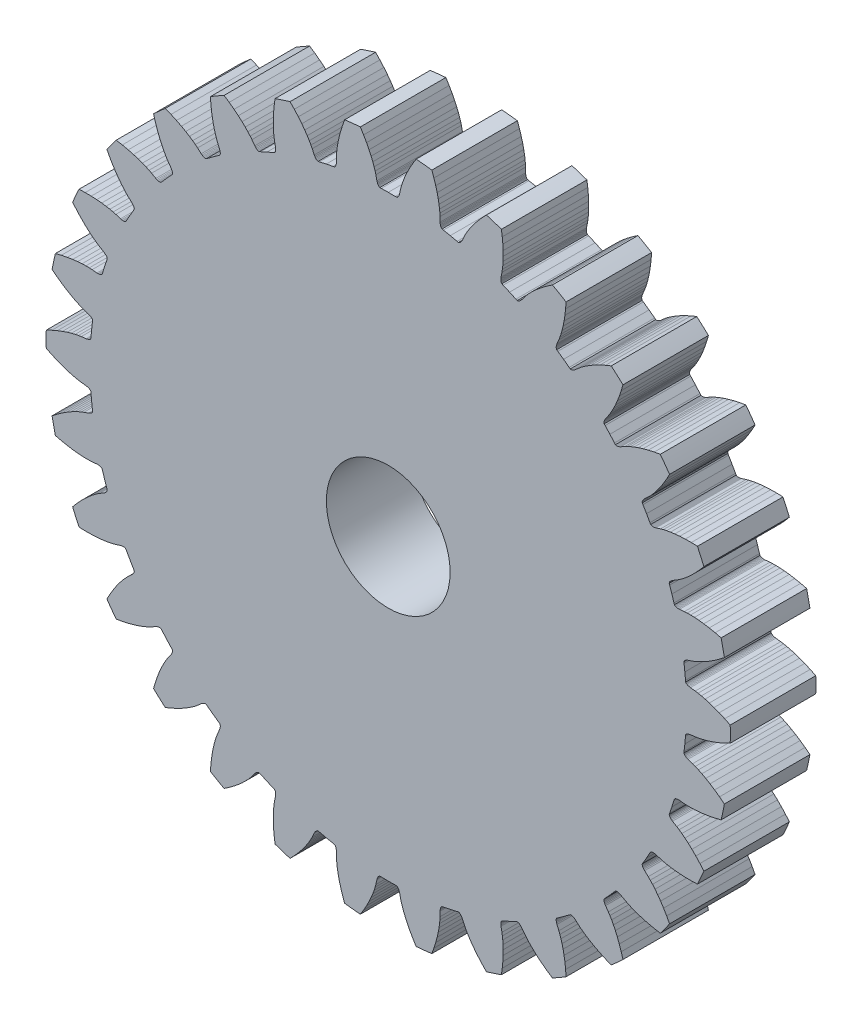
SolidWorks part; units mm, degrees
ref_plane "Front Plane" through (0, 0, 0) normal (0, 0, 1) x (1, 0, 0)
ref_plane "Top Plane" through (0, 0, 0) normal (0, 1, 0) x (1, 0, 0)
ref_plane "Right Plane" through (0, 0, 0) normal (1, 0, 0) x (0, 0, -1)
sketch "Model" plane through (0, 0, 0) normal (0, 0, 1) x (1, 0, 0)
  line L0 (393.5757, 70.825) -> (387.7273, 66.6582)
  line L1 (387.7273, 66.6582) -> (382.2635, 63.1016)
  line L2 (382.2635, 63.1016) -> (377.1984, 60.0983)
  line L3 (377.1984, 60.0983) -> (372.587, 57.6184)
  line L4 (372.587, 57.6184) -> (368.4431, 55.6071)
  line L5 (368.4431, 55.6071) -> (364.7654, 54.0079)
  line L6 (364.7654, 54.0079) -> (361.5999, 52.7864)
  line L7 (361.5999, 52.7864) -> (356.106, 50.9493)
  line L8 (356.106, 50.9493) -> (354.8773, 50.4167)
  line L9 (354.8773, 50.4167) -> (353.8273, 49.8583)
  line L10 (353.8273, 49.8583) -> (352.9562, 49.2818)
  line L11 (352.9562, 49.2818) -> (352.2643, 48.6939)
  line L12 (352.2643, 48.6939) -> (351.7516, 48.1024)
  line L13 (351.7516, 48.1024) -> (351.4181, 47.5142)
  line L14 (351.4181, 47.5142) -> (351.2632, 46.9365)
  line L15 (351.2632, 46.9365) -> (351.4248, 45.2901)
  line L16 (351.4248, 45.2901) -> (352.3889, 37.0376)
  line L17 (352.3889, 37.0376) -> (353.1616, 28.7649)
  line L18 (353.1616, 28.7649) -> (353.3459, 27.1209)
  line L19 (353.3459, 27.1209) -> (353.6175, 26.5881)
  line L20 (353.6175, 26.5881) -> (354.066, 26.082)
  line L21 (354.066, 26.082) -> (354.6905, 25.61)
  line L22 (354.6905, 25.61) -> (355.4895, 25.1789)
  line L23 (355.4895, 25.1789) -> (356.4615, 24.796)
  line L24 (356.4615, 24.796) -> (357.6046, 24.4682)
  line L25 (357.6046, 24.4682) -> (358.9172, 24.2026)
  line L26 (358.9172, 24.2026) -> (364.673, 23.548)
  line L27 (364.673, 23.548) -> (368.0233, 23.0113)
  line L28 (368.0233, 23.0113) -> (371.9531, 22.2117)
  line L29 (371.9531, 22.2117) -> (376.4246, 21.1059)
  line L30 (376.4246, 21.1059) -> (381.4508, 19.639)
  line L31 (381.4508, 19.639) -> (387.0296, 17.7543)
  line L32 (387.0296, 17.7543) -> (393.1135, 15.4115)
  line L33 (393.1135, 15.4115) -> (399.7005, 12.5517)
  line L34 (399.7005, 12.5517) -> (406.2919, 9.3617)
  line L35 (406.2919, -9.3617) -> (399.7005, -12.5517)
  line L36 (399.7005, -12.5517) -> (393.1135, -15.4115)
  line L37 (393.1135, -15.4115) -> (387.0296, -17.7543)
  line L38 (387.0296, -17.7543) -> (381.4508, -19.639)
  line L39 (381.4508, -19.639) -> (376.4246, -21.1059)
  line L40 (376.4246, -21.1059) -> (371.9531, -22.2117)
  line L41 (371.9531, -22.2117) -> (368.0233, -23.0113)
  line L42 (368.0233, -23.0113) -> (364.673, -23.548)
  line L43 (364.673, -23.548) -> (358.9172, -24.2026)
  line L44 (358.9172, -24.2026) -> (357.6046, -24.4682)
  line L45 (357.6046, -24.4682) -> (356.4615, -24.796)
  line L46 (356.4615, -24.796) -> (355.4895, -25.1789)
  line L47 (355.4895, -25.1789) -> (354.6905, -25.61)
  line L48 (354.6905, -25.61) -> (354.066, -26.082)
  line L49 (354.066, -26.082) -> (353.6175, -26.5881)
  line L50 (353.6175, -26.5881) -> (353.3459, -27.1209)
  line L51 (353.3459, -27.1209) -> (353.1616, -28.7649)
  line L52 (353.1616, -28.7649) -> (352.3889, -37.0376)
  line L53 (352.3889, -37.0376) -> (351.4248, -45.2901)
  line L54 (351.4248, -45.2901) -> (351.2632, -46.9365)
  line L55 (351.2632, -46.9365) -> (351.4181, -47.5142)
  line L56 (351.4181, -47.5142) -> (351.7516, -48.1024)
  line L57 (351.7516, -48.1024) -> (352.2643, -48.6939)
  line L58 (352.2643, -48.6939) -> (352.9562, -49.2818)
  line L59 (352.9562, -49.2818) -> (353.8273, -49.8583)
  line L60 (353.8273, -49.8583) -> (354.8773, -50.4167)
  line L61 (354.8773, -50.4167) -> (356.106, -50.9493)
  line L62 (356.106, -50.9493) -> (361.5999, -52.7864)
  line L63 (361.5999, -52.7864) -> (364.7654, -54.0079)
  line L64 (364.7654, -54.0079) -> (368.4431, -55.6071)
  line L65 (368.4431, -55.6071) -> (372.587, -57.6184)
  line L66 (372.587, -57.6184) -> (377.1984, -60.0983)
  line L67 (377.1984, -60.0983) -> (382.2635, -63.1016)
  line L68 (382.2635, -63.1016) -> (387.7273, -66.6582)
  line L69 (387.7273, -66.6582) -> (393.5757, -70.825)
  line L70 (393.5757, -70.825) -> (399.3599, -75.3157)
  line L71 (395.4671, -93.63) -> (388.3565, -95.3798)
  line L72 (388.3565, -95.3798) -> (381.3188, -96.8076)
  line L73 (381.3188, -96.8076) -> (374.8808, -97.8344)
  line L74 (374.8808, -97.8344) -> (369.032, -98.5179)
  line L75 (369.032, -98.5179) -> (363.8107, -98.9077)
  line L76 (363.8107, -98.9077) -> (359.207, -99.0597)
  line L77 (359.207, -99.0597) -> (355.1967, -99.0248)
  line L78 (355.1967, -99.0248) -> (351.8081, -98.8532)
  line L79 (351.8081, -98.8532) -> (346.042, -98.2968)
  line L80 (346.042, -98.2968) -> (344.7029, -98.2837)
  line L81 (344.7029, -98.2837) -> (343.5166, -98.3667)
  line L82 (343.5166, -98.3667) -> (342.4863, -98.5391)
  line L83 (342.4863, -98.5391) -> (341.6151, -98.7947)
  line L84 (341.6151, -98.7947) -> (340.9061, -99.1265)
  line L85 (340.9061, -99.1265) -> (340.3621, -99.5283)
  line L86 (340.3621, -99.5283) -> (339.9857, -99.993)
  line L87 (339.9857, -99.993) -> (339.4636, -101.5628)
  line L88 (339.4636, -101.5628) -> (336.9879, -109.494)
  line L89 (336.9879, -109.494) -> (334.329, -117.3657)
  line L90 (334.329, -117.3657) -> (333.8286, -118.9426)
  line L91 (333.8286, -118.9426) -> (333.86, -119.5398)
  line L92 (333.86, -119.5398) -> (334.0639, -120.1845)
  line L93 (334.0639, -120.1845) -> (334.4425, -120.8697)
  line L94 (334.4425, -120.8697) -> (334.997, -121.5886)
  line L95 (334.997, -121.5886) -> (335.7292, -122.3336)
  line L96 (335.7292, -122.3336) -> (336.6402, -123.0981)
  line L97 (336.6402, -123.0981) -> (337.7313, -123.8746)
  line L98 (337.7313, -123.8746) -> (342.7232, -126.8137)
  line L99 (342.7232, -126.8137) -> (345.5655, -128.6667)
  line L100 (345.5655, -128.6667) -> (348.8304, -130.9955)
  line L101 (348.8304, -130.9955) -> (352.4656, -133.8245)
  line L102 (352.4656, -133.8245) -> (356.4605, -137.2089)
  line L103 (356.4605, -137.2089) -> (360.7905, -141.1997)
  line L104 (360.7905, -141.1997) -> (365.3955, -145.8146)
  line L105 (365.3955, -145.8146) -> (370.2498, -151.1063)
  line L106 (370.2498, -151.1063) -> (374.9739, -156.7015)
  line L107 (367.3584, -173.8062) -> (360.0393, -174.0394)
  line L108 (360.0393, -174.0394) -> (352.8587, -173.9728)
  line L109 (352.8587, -173.9728) -> (346.3478, -173.6385)
  line L110 (346.3478, -173.6385) -> (340.4848, -173.0911)
  line L111 (340.4848, -173.0911) -> (335.2965, -172.3869)
  line L112 (335.2965, -172.3869) -> (330.7617, -171.5784)
  line L113 (330.7617, -171.5784) -> (326.8464, -170.7104)
  line L114 (326.8464, -170.7104) -> (323.5675, -169.838)
  line L115 (323.5675, -169.838) -> (318.0431, -168.095)
  line L116 (318.0431, -168.095) -> (316.736, -167.8037)
  line L117 (316.736, -167.8037) -> (315.5583, -167.6382)
  line L118 (315.5583, -167.6382) -> (314.5147, -167.5927)
  line L119 (314.5147, -167.5927) -> (313.6094, -167.6616)
  line L120 (313.6094, -167.6616) -> (312.8469, -167.8387)
  line L121 (312.8469, -167.8387) -> (312.2313, -168.1186)
  line L122 (312.2313, -168.1186) -> (311.7665, -168.4949)
  line L123 (311.7665, -168.4949) -> (310.9295, -169.9219)
  line L124 (310.9295, -169.9219) -> (306.8588, -177.165)
  line L125 (306.8588, -177.165) -> (302.6214, -184.3119)
  line L126 (302.6214, -184.3119) -> (301.8041, -185.7503)
  line L127 (301.8041, -185.7503) -> (301.7106, -186.3409)
  line L128 (301.7106, -186.3409) -> (301.7761, -187.014)
  line L129 (301.7761, -187.014) -> (302.0039, -187.7629)
  line L130 (302.0039, -187.7629) -> (302.3969, -188.5814)
  line L131 (302.3969, -188.5814) -> (302.9581, -189.4624)
  line L132 (302.9581, -189.4624) -> (303.6903, -190.3995)
  line L133 (303.6903, -190.3995) -> (304.5961, -191.3859)
  line L134 (304.5961, -191.3859) -> (308.8678, -195.2987)
  line L135 (308.8678, -195.2987) -> (311.2628, -197.7021)
  line L136 (311.2628, -197.7021) -> (313.9721, -200.6589)
  line L137 (313.9721, -200.6589) -> (316.9397, -204.1818)
  line L138 (316.9397, -204.1818) -> (320.1437, -208.3229)
  line L139 (320.1437, -208.3229) -> (323.5493, -213.1268)
  line L140 (323.5493, -213.1268) -> (327.0942, -218.5982)
  line L141 (327.0942, -218.5982) -> (330.7422, -224.7835)
  line L142 (330.7422, -224.7835) -> (334.1998, -231.2386)
  line L143 (323.1944, -246.3862) -> (315.9868, -245.0926)
  line L144 (315.9868, -245.0926) -> (308.9769, -243.5345)
  line L145 (308.9769, -243.5345) -> (302.6778, -241.8539)
  line L146 (302.6778, -241.8539) -> (297.0567, -240.0994)
  line L147 (297.0567, -240.0994) -> (292.1282, -238.3319)
  line L148 (292.1282, -238.3319) -> (287.8607, -236.5982)
  line L149 (287.8607, -236.5982) -> (284.2114, -234.9352)
  line L150 (284.2114, -234.9352) -> (281.1855, -233.4001)
  line L151 (281.1855, -233.4001) -> (276.1442, -230.5466)
  line L152 (276.1442, -230.5466) -> (274.9262, -229.9899)
  line L153 (274.9262, -229.9899) -> (273.8087, -229.5832)
  line L154 (273.8087, -229.5832) -> (272.7973, -229.3216)
  line L155 (272.7973, -229.3216) -> (271.8975, -229.2008)
  line L156 (271.8975, -229.2008) -> (271.1148, -229.2156)
  line L157 (271.1148, -229.2156) -> (270.4545, -229.3613)
  line L158 (270.4545, -229.3613) -> (269.9216, -229.6328)
  line L159 (269.9216, -229.6328) -> (268.8062, -230.8545)
  line L160 (268.8062, -230.8545) -> (263.3185, -237.093)
  line L161 (263.3185, -237.093) -> (257.6878, -243.2027)
  line L162 (257.6878, -243.2027) -> (256.5893, -244.4398)
  line L163 (256.5893, -244.4398) -> (256.3751, -244.9981)
  line L164 (256.3751, -244.9981) -> (256.2991, -245.6701)
  line L165 (256.2991, -245.6701) -> (256.3663, -246.45)
  line L166 (256.3663, -246.45) -> (256.5805, -247.3323)
  line L167 (256.5805, -247.3323) -> (256.9463, -248.3107)
  line L168 (256.9463, -248.3107) -> (257.4676, -249.3796)
  line L169 (257.4676, -249.3796) -> (258.1485, -250.5327)
  line L170 (258.1485, -250.5327) -> (261.5134, -255.2482)
  line L171 (261.5134, -255.2482) -> (263.3564, -258.097)
  line L172 (263.3564, -258.097) -> (265.3917, -261.5525)
  line L173 (265.3917, -261.5525) -> (267.562, -265.6154)
  line L174 (267.562, -265.6154) -> (269.835, -270.3322)
  line L175 (269.835, -270.3322) -> (272.1674, -275.7391)
  line L176 (272.1674, -275.7391) -> (274.4973, -281.828)
  line L177 (274.4973, -281.828) -> (276.7796, -288.6366)
  line L178 (276.7796, -288.6366) -> (278.8195, -295.6695)
  line L179 (264.9053, -308.198) -> (258.1241, -305.4341)
  line L180 (258.1241, -305.4341) -> (251.5913, -302.4526)
  line L181 (251.5913, -302.4526) -> (245.7793, -299.4991)
  line L182 (245.7793, -299.4991) -> (240.6458, -296.6142)
  line L183 (240.6458, -296.6142) -> (236.1925, -293.8606)
  line L184 (236.1925, -293.8606) -> (232.3787, -291.2776)
  line L185 (232.3787, -291.2776) -> (229.1549, -288.8921)
  line L186 (229.1549, -288.8921) -> (226.5143, -286.7615)
  line L187 (226.5143, -286.7615) -> (222.1764, -282.9222)
  line L188 (222.1764, -282.9222) -> (221.1008, -282.1244)
  line L189 (221.1008, -282.1244) -> (220.0922, -281.4943)
  line L190 (220.0922, -281.4943) -> (219.1574, -281.0282)
  line L191 (219.1574, -281.0282) -> (218.3023, -280.7229)
  line L192 (218.3023, -280.7229) -> (217.5337, -280.5746)
  line L193 (217.5337, -280.5746) -> (216.8575, -280.5799)
  line L194 (216.8575, -280.5799) -> (216.2798, -280.7346)
  line L195 (216.2798, -280.7346) -> (214.9347, -281.6977)
  line L196 (214.9347, -281.6977) -> (208.2699, -286.659)
  line L197 (208.2699, -286.659) -> (201.492, -291.4645)
  line L198 (201.492, -291.4645) -> (200.1603, -292.4461)
  line L199 (200.1603, -292.4461) -> (199.8347, -292.9477)
  line L200 (199.8347, -292.9477) -> (199.6207, -293.5892)
  line L201 (199.6207, -293.5892) -> (199.5242, -294.366)
  line L202 (199.5242, -294.366) -> (199.5503, -295.2735)
  line L203 (199.5503, -295.2735) -> (199.7047, -296.3067)
  line L204 (199.7047, -296.3067) -> (199.9924, -297.4606)
  line L205 (199.9924, -297.4606) -> (200.4187, -298.7301)
  line L206 (200.4187, -298.7301) -> (202.7296, -304.0421)
  line L207 (202.7296, -304.0421) -> (203.94, -307.2118)
  line L208 (203.94, -307.2118) -> (205.2125, -311.015)
  line L209 (205.2125, -311.015) -> (206.4905, -315.4404)
  line L210 (206.4905, -315.4404) -> (207.7333, -320.5266)
  line L211 (207.7333, -320.5266) -> (208.8905, -326.3003)
  line L212 (208.8905, -326.3003) -> (209.9035, -332.7406)
  line L213 (209.9035, -332.7406) -> (210.7204, -339.8749)
  line L214 (210.7204, -339.8749) -> (211.2534, -347.1783)
  line L215 (195.0385, -356.54) -> (188.9802, -352.4267)
  line L216 (188.9802, -352.4267) -> (183.21, -348.1521)
  line L217 (183.21, -348.1521) -> (178.1391, -344.0547)
  line L218 (178.1391, -344.0547) -> (173.7176, -340.1656)
  line L219 (173.7176, -340.1656) -> (169.9341, -336.5462)
  line L220 (169.9341, -336.5462) -> (166.7406, -333.2267)
  line L221 (166.7406, -333.2267) -> (164.0833, -330.2231)
  line L222 (164.0833, -330.2231) -> (161.9434, -327.59)
  line L223 (161.9434, -327.59) -> (158.4985, -322.9327)
  line L224 (158.4985, -322.9327) -> (157.6122, -321.9288)
  line L225 (157.6122, -321.9288) -> (156.7567, -321.1027)
  line L226 (156.7567, -321.1027) -> (155.9392, -320.4524)
  line L227 (155.9392, -320.4524) -> (155.1663, -319.976)
  line L228 (155.1663, -319.976) -> (154.4453, -319.6712)
  line L229 (154.4453, -319.6712) -> (153.7828, -319.5358)
  line L230 (153.7828, -319.5358) -> (153.1856, -319.567)
  line L231 (153.1856, -319.567) -> (151.6697, -320.2294)
  line L232 (151.6697, -320.2294) -> (144.119, -323.6966)
  line L233 (144.119, -323.6966) -> (136.49, -326.9878)
  line L234 (136.49, -326.9878) -> (134.9834, -327.6711)
  line L235 (134.9834, -327.6711) -> (134.5606, -328.094)
  line L236 (134.5606, -328.094) -> (134.2179, -328.677)
  line L237 (134.2179, -328.677) -> (133.962, -329.4168)
  line L238 (133.962, -329.4168) -> (133.7988, -330.3099)
  line L239 (133.7988, -330.3099) -> (133.7351, -331.3526)
  line L240 (133.7351, -331.3526) -> (133.7766, -332.5411)
  line L241 (133.7766, -332.5411) -> (133.9296, -333.8715)
  line L242 (133.9296, -333.8715) -> (135.0856, -339.5479)
  line L243 (135.0856, -339.5479) -> (135.6105, -342.9)
  line L244 (135.6105, -342.9) -> (136.0644, -346.8846)
  line L245 (136.0644, -346.8846) -> (136.3945, -351.479)
  line L246 (136.3945, -351.479) -> (136.5526, -356.7125)
  line L247 (136.5526, -356.7125) -> (136.4841, -362.6007)
  line L248 (136.4841, -362.6007) -> (136.136, -369.1108)
  line L249 (136.136, -369.1108) -> (135.4516, -376.2591)
  line L250 (135.4516, -376.2591) -> (134.4546, -383.5137)
  line L251 (116.6476, -389.2995) -> (111.5769, -384.0165)
  line L252 (111.5769, -384.0165) -> (106.8216, -378.6356)
  line L253 (106.8216, -378.6356) -> (102.7134, -373.5735)
  line L254 (102.7134, -373.5735) -> (99.197, -368.8501)
  line L255 (99.197, -368.8501) -> (96.2487, -364.5232)
  line L256 (96.2487, -364.5232) -> (93.8152, -360.6122)
  line L257 (93.8152, -360.6122) -> (91.8404, -357.1218)
  line L258 (91.8404, -357.1218) -> (90.2947, -354.1013)
  line L259 (90.2947, -354.1013) -> (87.8934, -348.8296)
  line L260 (87.8934, -348.8296) -> (87.2353, -347.6633)
  line L261 (87.2353, -347.6633) -> (86.5702, -346.6774)
  line L262 (86.5702, -346.6774) -> (85.9058, -345.8713)
  line L263 (85.9058, -345.8713) -> (85.2488, -345.2447)
  line L264 (85.2488, -345.2447) -> (84.607, -344.7966)
  line L265 (84.607, -344.7966) -> (83.9871, -344.5264)
  line L266 (83.9871, -344.5264) -> (83.3964, -344.4328)
  line L267 (83.3964, -344.4328) -> (81.7759, -344.7655)
  line L268 (81.7759, -344.7655) -> (73.6693, -346.587)
  line L269 (73.6693, -346.587) -> (65.5228, -348.2202)
  line L270 (65.5228, -348.2202) -> (63.907, -348.5754)
  line L271 (63.907, -348.5754) -> (63.4055, -348.9011)
  line L272 (63.4055, -348.9011) -> (62.9491, -349.4001)
  line L273 (62.9491, -349.4001) -> (62.545, -350.0705)
  line L274 (62.545, -350.0705) -> (62.1997, -350.9102)
  line L275 (62.1997, -350.9102) -> (61.9206, -351.9169)
  line L276 (61.9206, -351.9169) -> (61.714, -353.088)
  line L277 (61.714, -353.088) -> (61.5871, -354.4211)
  line L278 (61.5871, -354.4211) -> (61.5377, -360.2138)
  line L279 (61.5377, -360.2138) -> (61.3541, -363.6019)
  line L280 (61.3541, -363.6019) -> (60.9697, -367.5937)
  line L281 (60.9697, -367.5937) -> (60.3373, -372.1564)
  line L282 (60.3373, -372.1564) -> (59.4039, -377.3084)
  line L283 (59.4039, -377.3084) -> (58.1127, -383.0536)
  line L284 (58.1127, -383.0536) -> (56.4186, -389.3491)
  line L285 (56.4186, -389.3491) -> (54.263, -396.1989)
  line L286 (54.263, -396.1989) -> (51.7795, -403.0877)
  line L287 (33.1586, -405.0448) -> (29.2971, -398.8229)
  line L288 (29.2971, -398.8229) -> (25.7645, -392.571)
  line L289 (25.7645, -392.571) -> (22.7985, -386.7653)
  line L290 (22.7985, -386.7653) -> (20.3411, -381.414)
  line L291 (20.3411, -381.414) -> (18.3568, -376.5687)
  line L292 (18.3568, -376.5687) -> (16.7897, -372.2373)
  line L293 (16.7897, -372.2373) -> (15.5837, -368.4125)
  line L294 (15.5837, -368.4125) -> (14.6997, -365.1367)
  line L295 (14.6997, -365.1367) -> (13.447, -359.4809)
  line L296 (13.447, -359.4809) -> (13.0457, -358.2032)
  line L297 (13.0457, -358.2032) -> (12.6002, -357.1006)
  line L298 (12.6002, -357.1006) -> (12.1178, -356.174)
  line L299 (12.1178, -356.174) -> (11.6055, -355.4245)
  line L300 (11.6055, -355.4245) -> (11.0708, -354.8527)
  line L301 (11.0708, -354.8527) -> (10.5207, -354.4595)
  line L302 (10.5207, -354.4595) -> (9.9624, -354.2452)
  line L303 (9.9624, -354.2452) -> (8.3081, -354.2337)
  line L304 (8.3081, -354.2337) -> (0, -354.33)
  line L305 (0, -354.33) -> (-8.3081, -354.2337)
  line L306 (-8.3081, -354.2337) -> (-9.9624, -354.2452)
  line L307 (-9.9624, -354.2452) -> (-10.5207, -354.4595)
  line L308 (-10.5207, -354.4595) -> (-11.0708, -354.8527)
  line L309 (-11.0708, -354.8527) -> (-11.6055, -355.4245)
  line L310 (-11.6055, -355.4245) -> (-12.1178, -356.174)
  line L311 (-12.1178, -356.174) -> (-12.6002, -357.1006)
  line L312 (-12.6002, -357.1006) -> (-13.0457, -358.2032)
  line L313 (-13.0457, -358.2032) -> (-13.447, -359.4809)
  line L314 (-13.447, -359.4809) -> (-14.6997, -365.1367)
  line L315 (-14.6997, -365.1367) -> (-15.5837, -368.4125)
  line L316 (-15.5837, -368.4125) -> (-16.7897, -372.2373)
  line L317 (-16.7897, -372.2373) -> (-18.3568, -376.5687)
  line L318 (-18.3568, -376.5687) -> (-20.3411, -381.414)
  line L319 (-20.3411, -381.414) -> (-22.7985, -386.7653)
  line L320 (-22.7985, -386.7653) -> (-25.7645, -392.571)
  line L321 (-25.7645, -392.571) -> (-29.2971, -398.8229)
  line L322 (-29.2971, -398.8229) -> (-33.1586, -405.0448)
  line L323 (-51.7795, -403.0877) -> (-54.263, -396.1989)
  line L324 (-54.263, -396.1989) -> (-56.4186, -389.3491)
  line L325 (-56.4186, -389.3491) -> (-58.1127, -383.0536)
  line L326 (-58.1127, -383.0536) -> (-59.4039, -377.3084)
  line L327 (-59.4039, -377.3084) -> (-60.3373, -372.1564)
  line L328 (-60.3373, -372.1564) -> (-60.9697, -367.5937)
  line L329 (-60.9697, -367.5937) -> (-61.3541, -363.6019)
  line L330 (-61.3541, -363.6019) -> (-61.5377, -360.2138)
  line L331 (-61.5377, -360.2138) -> (-61.5871, -354.4211)
  line L332 (-61.5871, -354.4211) -> (-61.714, -353.088)
  line L333 (-61.714, -353.088) -> (-61.9206, -351.9169)
  line L334 (-61.9206, -351.9169) -> (-62.1997, -350.9102)
  line L335 (-62.1997, -350.9102) -> (-62.545, -350.0705)
  line L336 (-62.545, -350.0705) -> (-62.9491, -349.4001)
  line L337 (-62.9491, -349.4001) -> (-63.4055, -348.9011)
  line L338 (-63.4055, -348.9011) -> (-63.907, -348.5754)
  line L339 (-63.907, -348.5754) -> (-65.5228, -348.2202)
  line L340 (-65.5228, -348.2202) -> (-73.6693, -346.587)
  line L341 (-73.6693, -346.587) -> (-81.7759, -344.7655)
  line L342 (-81.7759, -344.7655) -> (-83.3964, -344.4328)
  line L343 (-83.3964, -344.4328) -> (-83.9871, -344.5264)
  line L344 (-83.9871, -344.5264) -> (-84.607, -344.7966)
  line L345 (-84.607, -344.7966) -> (-85.2488, -345.2447)
  line L346 (-85.2488, -345.2447) -> (-85.9058, -345.8713)
  line L347 (-85.9058, -345.8713) -> (-86.5702, -346.6774)
  line L348 (-86.5702, -346.6774) -> (-87.2353, -347.6633)
  line L349 (-87.2353, -347.6633) -> (-87.8934, -348.8296)
  line L350 (-87.8934, -348.8296) -> (-90.2947, -354.1013)
  line L351 (-90.2947, -354.1013) -> (-91.8404, -357.1218)
  line L352 (-91.8404, -357.1218) -> (-93.8152, -360.6122)
  line L353 (-93.8152, -360.6122) -> (-96.2487, -364.5232)
  line L354 (-96.2487, -364.5232) -> (-99.197, -368.8501)
  line L355 (-99.197, -368.8501) -> (-102.7134, -373.5735)
  line L356 (-102.7134, -373.5735) -> (-106.8216, -378.6356)
  line L357 (-106.8216, -378.6356) -> (-111.5769, -384.0165)
  line L358 (-111.5769, -384.0165) -> (-116.6476, -389.2995)
  line L359 (-134.4546, -383.5137) -> (-135.4516, -376.2591)
  line L360 (-135.4516, -376.2591) -> (-136.136, -369.1108)
  line L361 (-136.136, -369.1108) -> (-136.4841, -362.6007)
  line L362 (-136.4841, -362.6007) -> (-136.5526, -356.7125)
  line L363 (-136.5526, -356.7125) -> (-136.3945, -351.479)
  line L364 (-136.3945, -351.479) -> (-136.0644, -346.8846)
  line L365 (-136.0644, -346.8846) -> (-135.6105, -342.9)
  line L366 (-135.6105, -342.9) -> (-135.0856, -339.5479)
  line L367 (-135.0856, -339.5479) -> (-133.9296, -333.8715)
  line L368 (-133.9296, -333.8715) -> (-133.7766, -332.5411)
  line L369 (-133.7766, -332.5411) -> (-133.7351, -331.3526)
  line L370 (-133.7351, -331.3526) -> (-133.7988, -330.3099)
  line L371 (-133.7988, -330.3099) -> (-133.962, -329.4168)
  line L372 (-133.962, -329.4168) -> (-134.2179, -328.677)
  line L373 (-134.2179, -328.677) -> (-134.5606, -328.094)
  line L374 (-134.5606, -328.094) -> (-134.9834, -327.6711)
  line L375 (-134.9834, -327.6711) -> (-136.49, -326.9878)
  line L376 (-136.49, -326.9878) -> (-144.119, -323.6966)
  line L377 (-144.119, -323.6966) -> (-151.6697, -320.2294)
  line L378 (-151.6697, -320.2294) -> (-153.1856, -319.567)
  line L379 (-153.1856, -319.567) -> (-153.7828, -319.5358)
  line L380 (-153.7828, -319.5358) -> (-154.4453, -319.6712)
  line L381 (-154.4453, -319.6712) -> (-155.1663, -319.976)
  line L382 (-155.1663, -319.976) -> (-155.9392, -320.4524)
  line L383 (-155.9392, -320.4524) -> (-156.7567, -321.1027)
  line L384 (-156.7567, -321.1027) -> (-157.6122, -321.9288)
  line L385 (-157.6122, -321.9288) -> (-158.4985, -322.9327)
  line L386 (-158.4985, -322.9327) -> (-161.9434, -327.59)
  line L387 (-161.9434, -327.59) -> (-164.0833, -330.2231)
  line L388 (-164.0833, -330.2231) -> (-166.7406, -333.2267)
  line L389 (-166.7406, -333.2267) -> (-169.9341, -336.5462)
  line L390 (-169.9341, -336.5462) -> (-173.7176, -340.1656)
  line L391 (-173.7176, -340.1656) -> (-178.1391, -344.0547)
  line L392 (-178.1391, -344.0547) -> (-183.21, -348.1521)
  line L393 (-183.21, -348.1521) -> (-188.9802, -352.4267)
  line L394 (-188.9802, -352.4267) -> (-195.0385, -356.54)
  line L395 (-211.2534, -347.1783) -> (-210.7204, -339.8749)
  line L396 (-210.7204, -339.8749) -> (-209.9035, -332.7406)
  line L397 (-209.9035, -332.7406) -> (-208.8905, -326.3003)
  line L398 (-208.8905, -326.3003) -> (-207.7333, -320.5266)
  line L399 (-207.7333, -320.5266) -> (-206.4905, -315.4404)
  line L400 (-206.4905, -315.4404) -> (-205.2125, -311.015)
  line L401 (-205.2125, -311.015) -> (-203.94, -307.2118)
  line L402 (-203.94, -307.2118) -> (-202.7296, -304.0421)
  line L403 (-202.7296, -304.0421) -> (-200.4187, -298.7301)
  line L404 (-200.4187, -298.7301) -> (-199.9924, -297.4606)
  line L405 (-199.9924, -297.4606) -> (-199.7047, -296.3067)
  line L406 (-199.7047, -296.3067) -> (-199.5503, -295.2735)
  line L407 (-199.5503, -295.2735) -> (-199.5242, -294.366)
  line L408 (-199.5242, -294.366) -> (-199.6207, -293.5892)
  line L409 (-199.6207, -293.5892) -> (-199.8347, -292.9477)
  line L410 (-199.8347, -292.9477) -> (-200.1603, -292.4461)
  line L411 (-200.1603, -292.4461) -> (-201.492, -291.4645)
  line L412 (-201.492, -291.4645) -> (-208.2699, -286.659)
  line L413 (-208.2699, -286.659) -> (-214.9347, -281.6977)
  line L414 (-214.9347, -281.6977) -> (-216.2798, -280.7346)
  line L415 (-216.2798, -280.7346) -> (-216.8575, -280.5799)
  line L416 (-216.8575, -280.5799) -> (-217.5337, -280.5746)
  line L417 (-217.5337, -280.5746) -> (-218.3023, -280.7229)
  line L418 (-218.3023, -280.7229) -> (-219.1574, -281.0282)
  line L419 (-219.1574, -281.0282) -> (-220.0922, -281.4943)
  line L420 (-220.0922, -281.4943) -> (-221.1008, -282.1244)
  line L421 (-221.1008, -282.1244) -> (-222.1764, -282.9222)
  line L422 (-222.1764, -282.9222) -> (-226.5143, -286.7615)
  line L423 (-226.5143, -286.7615) -> (-229.1549, -288.8921)
  line L424 (-229.1549, -288.8921) -> (-232.3787, -291.2776)
  line L425 (-232.3787, -291.2776) -> (-236.1925, -293.8606)
  line L426 (-236.1925, -293.8606) -> (-240.6458, -296.6142)
  line L427 (-240.6458, -296.6142) -> (-245.7793, -299.4991)
  line L428 (-245.7793, -299.4991) -> (-251.5913, -302.4526)
  line L429 (-251.5913, -302.4526) -> (-258.1241, -305.4341)
  line L430 (-258.1241, -305.4341) -> (-264.9053, -308.198)
  line L431 (-278.8195, -295.6695) -> (-276.7796, -288.6366)
  line L432 (-276.7796, -288.6366) -> (-274.4973, -281.828)
  line L433 (-274.4973, -281.828) -> (-272.1674, -275.7391)
  line L434 (-272.1674, -275.7391) -> (-269.835, -270.3322)
  line L435 (-269.835, -270.3322) -> (-267.562, -265.6154)
  line L436 (-267.562, -265.6154) -> (-265.3917, -261.5525)
  line L437 (-265.3917, -261.5525) -> (-263.3564, -258.097)
  line L438 (-263.3564, -258.097) -> (-261.5134, -255.2482)
  line L439 (-261.5134, -255.2482) -> (-258.1485, -250.5327)
  line L440 (-258.1485, -250.5327) -> (-257.4676, -249.3796)
  line L441 (-257.4676, -249.3796) -> (-256.9463, -248.3107)
  line L442 (-256.9463, -248.3107) -> (-256.5805, -247.3323)
  line L443 (-256.5805, -247.3323) -> (-256.3663, -246.45)
  line L444 (-256.3663, -246.45) -> (-256.2991, -245.6701)
  line L445 (-256.2991, -245.6701) -> (-256.3751, -244.9981)
  line L446 (-256.3751, -244.9981) -> (-256.5893, -244.4398)
  line L447 (-256.5893, -244.4398) -> (-257.6878, -243.2027)
  line L448 (-257.6878, -243.2027) -> (-263.3185, -237.093)
  line L449 (-263.3185, -237.093) -> (-268.8062, -230.8545)
  line L450 (-268.8062, -230.8545) -> (-269.9216, -229.6328)
  line L451 (-269.9216, -229.6328) -> (-270.4545, -229.3613)
  line L452 (-270.4545, -229.3613) -> (-271.1148, -229.2156)
  line L453 (-271.1148, -229.2156) -> (-271.8975, -229.2008)
  line L454 (-271.8975, -229.2008) -> (-272.7973, -229.3216)
  line L455 (-272.7973, -229.3216) -> (-273.8087, -229.5832)
  line L456 (-273.8087, -229.5832) -> (-274.9262, -229.9899)
  line L457 (-274.9262, -229.9899) -> (-276.1442, -230.5466)
  line L458 (-276.1442, -230.5466) -> (-281.1855, -233.4001)
  line L459 (-281.1855, -233.4001) -> (-284.2114, -234.9352)
  line L460 (-284.2114, -234.9352) -> (-287.8607, -236.5982)
  line L461 (-287.8607, -236.5982) -> (-292.1282, -238.3319)
  line L462 (-292.1282, -238.3319) -> (-297.0567, -240.0994)
  line L463 (-297.0567, -240.0994) -> (-302.6778, -241.8539)
  line L464 (-302.6778, -241.8539) -> (-308.9769, -243.5345)
  line L465 (-308.9769, -243.5345) -> (-315.9868, -245.0926)
  line L466 (-315.9868, -245.0926) -> (-323.1944, -246.3862)
  line L467 (-334.1998, -231.2386) -> (-330.7422, -224.7835)
  line L468 (-330.7422, -224.7835) -> (-327.0942, -218.5982)
  line L469 (-327.0942, -218.5982) -> (-323.5493, -213.1268)
  line L470 (-323.5493, -213.1268) -> (-320.1437, -208.3229)
  line L471 (-320.1437, -208.3229) -> (-316.9397, -204.1818)
  line L472 (-316.9397, -204.1818) -> (-313.9721, -200.6589)
  line L473 (-313.9721, -200.6589) -> (-311.2628, -197.7021)
  line L474 (-311.2628, -197.7021) -> (-308.8678, -195.2987)
  line L475 (-308.8678, -195.2987) -> (-304.5961, -191.3859)
  line L476 (-304.5961, -191.3859) -> (-303.6903, -190.3995)
  line L477 (-303.6903, -190.3995) -> (-302.9581, -189.4624)
  line L478 (-302.9581, -189.4624) -> (-302.3969, -188.5814)
  line L479 (-302.3969, -188.5814) -> (-302.0039, -187.7629)
  line L480 (-302.0039, -187.7629) -> (-301.7761, -187.014)
  line L481 (-301.7761, -187.014) -> (-301.7106, -186.3409)
  line L482 (-301.7106, -186.3409) -> (-301.8041, -185.7503)
  line L483 (-301.8041, -185.7503) -> (-302.6214, -184.3119)
  line L484 (-302.6214, -184.3119) -> (-306.8588, -177.165)
  line L485 (-306.8588, -177.165) -> (-310.9295, -169.9219)
  line L486 (-310.9295, -169.9219) -> (-311.7665, -168.4949)
  line L487 (-311.7665, -168.4949) -> (-312.2313, -168.1186)
  line L488 (-312.2313, -168.1186) -> (-312.8469, -167.8387)
  line L489 (-312.8469, -167.8387) -> (-313.6094, -167.6616)
  line L490 (-313.6094, -167.6616) -> (-314.5147, -167.5927)
  line L491 (-314.5147, -167.5927) -> (-315.5583, -167.6382)
  line L492 (-315.5583, -167.6382) -> (-316.736, -167.8037)
  line L493 (-316.736, -167.8037) -> (-318.0431, -168.095)
  line L494 (-318.0431, -168.095) -> (-323.5675, -169.838)
  line L495 (-323.5675, -169.838) -> (-326.8464, -170.7104)
  line L496 (-326.8464, -170.7104) -> (-330.7617, -171.5784)
  line L497 (-330.7617, -171.5784) -> (-335.2965, -172.3869)
  line L498 (-335.2965, -172.3869) -> (-340.4848, -173.0911)
  line L499 (-340.4848, -173.0911) -> (-346.3478, -173.6385)
  line L500 (-346.3478, -173.6385) -> (-352.8587, -173.9728)
  line L501 (-352.8587, -173.9728) -> (-360.0393, -174.0394)
  line L502 (-360.0393, -174.0394) -> (-367.3584, -173.8062)
  line L503 (-374.9739, -156.7015) -> (-370.2498, -151.1063)
  line L504 (-370.2498, -151.1063) -> (-365.3955, -145.8146)
  line L505 (-365.3955, -145.8146) -> (-360.7905, -141.1997)
  line L506 (-360.7905, -141.1997) -> (-356.4605, -137.2089)
  line L507 (-356.4605, -137.2089) -> (-352.4656, -133.8245)
  line L508 (-352.4656, -133.8245) -> (-348.8304, -130.9955)
  line L509 (-348.8304, -130.9955) -> (-345.5655, -128.6667)
  line L510 (-345.5655, -128.6667) -> (-342.7232, -126.8137)
  line L511 (-342.7232, -126.8137) -> (-337.7313, -123.8746)
  line L512 (-337.7313, -123.8746) -> (-336.6402, -123.0981)
  line L513 (-336.6402, -123.0981) -> (-335.7292, -122.3336)
  line L514 (-335.7292, -122.3336) -> (-334.997, -121.5886)
  line L515 (-334.997, -121.5886) -> (-334.4425, -120.8697)
  line L516 (-334.4425, -120.8697) -> (-334.0639, -120.1845)
  line L517 (-334.0639, -120.1845) -> (-333.86, -119.5398)
  line L518 (-333.86, -119.5398) -> (-333.8286, -118.9426)
  line L519 (-333.8286, -118.9426) -> (-334.329, -117.3657)
  line L520 (-334.329, -117.3657) -> (-336.9879, -109.494)
  line L521 (-336.9879, -109.494) -> (-339.4636, -101.5628)
  line L522 (-339.4636, -101.5628) -> (-339.9857, -99.993)
  line L523 (-339.9857, -99.993) -> (-340.3621, -99.5283)
  line L524 (-340.3621, -99.5283) -> (-340.9061, -99.1265)
  line L525 (-340.9061, -99.1265) -> (-341.6151, -98.7947)
  line L526 (-341.6151, -98.7947) -> (-342.4863, -98.5391)
  line L527 (-342.4863, -98.5391) -> (-343.5166, -98.3667)
  line L528 (-343.5166, -98.3667) -> (-344.7029, -98.2837)
  line L529 (-344.7029, -98.2837) -> (-346.042, -98.2968)
  line L530 (-346.042, -98.2968) -> (-351.8081, -98.8532)
  line L531 (-351.8081, -98.8532) -> (-355.1967, -99.0248)
  line L532 (-355.1967, -99.0248) -> (-359.207, -99.0597)
  line L533 (-359.207, -99.0597) -> (-363.8107, -98.9077)
  line L534 (-363.8107, -98.9077) -> (-369.032, -98.5179)
  line L535 (-369.032, -98.5179) -> (-374.8808, -97.8344)
  line L536 (-374.8808, -97.8344) -> (-381.3188, -96.8076)
  line L537 (-381.3188, -96.8076) -> (-388.3565, -95.3798)
  line L538 (-388.3565, -95.3798) -> (-395.4671, -93.63)
  line L539 (-399.3599, -75.3157) -> (-393.5757, -70.825)
  line L540 (-393.5757, -70.825) -> (-387.7273, -66.6582)
  line L541 (-387.7273, -66.6582) -> (-382.2635, -63.1016)
  line L542 (-382.2635, -63.1016) -> (-377.1984, -60.0983)
  line L543 (-377.1984, -60.0983) -> (-372.587, -57.6184)
  line L544 (-372.587, -57.6184) -> (-368.4431, -55.6071)
  line L545 (-368.4431, -55.6071) -> (-364.7654, -54.0079)
  line L546 (-364.7654, -54.0079) -> (-361.5999, -52.7864)
  line L547 (-361.5999, -52.7864) -> (-356.106, -50.9493)
  line L548 (-356.106, -50.9493) -> (-354.8773, -50.4167)
  line L549 (-354.8773, -50.4167) -> (-353.8273, -49.8583)
  line L550 (-353.8273, -49.8583) -> (-352.9562, -49.2818)
  line L551 (-352.9562, -49.2818) -> (-352.2643, -48.6939)
  line L552 (-352.2643, -48.6939) -> (-351.7516, -48.1024)
  line L553 (-351.7516, -48.1024) -> (-351.4181, -47.5142)
  line L554 (-351.4181, -47.5142) -> (-351.2632, -46.9365)
  line L555 (-351.2632, -46.9365) -> (-351.4248, -45.2901)
  line L556 (-351.4248, -45.2901) -> (-352.3889, -37.0376)
  line L557 (-352.3889, -37.0376) -> (-353.1616, -28.7649)
  line L558 (-353.1616, -28.7649) -> (-353.3459, -27.1209)
  line L559 (-353.3459, -27.1209) -> (-353.6175, -26.5881)
  line L560 (-353.6175, -26.5881) -> (-354.066, -26.082)
  line L561 (-354.066, -26.082) -> (-354.6905, -25.61)
  line L562 (-354.6905, -25.61) -> (-355.4895, -25.1789)
  line L563 (-355.4895, -25.1789) -> (-356.4615, -24.796)
  line L564 (-356.4615, -24.796) -> (-357.6046, -24.4682)
  line L565 (-357.6046, -24.4682) -> (-358.9172, -24.2026)
  line L566 (-358.9172, -24.2026) -> (-364.673, -23.548)
  line L567 (-364.673, -23.548) -> (-368.0233, -23.0113)
  line L568 (-368.0233, -23.0113) -> (-371.9531, -22.2117)
  line L569 (-371.9531, -22.2117) -> (-376.4246, -21.1059)
  line L570 (-376.4246, -21.1059) -> (-381.4508, -19.639)
  line L571 (-381.4508, -19.639) -> (-387.0296, -17.7543)
  line L572 (-387.0296, -17.7543) -> (-393.1135, -15.4115)
  line L573 (-393.1135, -15.4115) -> (-399.7005, -12.5517)
  line L574 (-399.7005, -12.5517) -> (-406.2919, -9.3617)
  line L575 (-406.2919, 9.3617) -> (-399.7005, 12.5517)
  line L576 (-399.7005, 12.5517) -> (-393.1135, 15.4115)
  line L577 (-393.1135, 15.4115) -> (-387.0296, 17.7543)
  line L578 (-387.0296, 17.7543) -> (-381.4508, 19.639)
  line L579 (-381.4508, 19.639) -> (-376.4246, 21.1059)
  line L580 (-376.4246, 21.1059) -> (-371.9531, 22.2117)
  line L581 (-371.9531, 22.2117) -> (-368.0233, 23.0113)
  line L582 (-368.0233, 23.0113) -> (-364.673, 23.548)
  line L583 (-364.673, 23.548) -> (-358.9172, 24.2026)
  line L584 (-358.9172, 24.2026) -> (-357.6046, 24.4682)
  line L585 (-357.6046, 24.4682) -> (-356.4615, 24.796)
  line L586 (-356.4615, 24.796) -> (-355.4895, 25.1789)
  line L587 (-355.4895, 25.1789) -> (-354.6905, 25.61)
  line L588 (-354.6905, 25.61) -> (-354.066, 26.082)
  line L589 (-354.066, 26.082) -> (-353.6175, 26.5881)
  line L590 (-353.6175, 26.5881) -> (-353.3459, 27.1209)
  line L591 (-353.3459, 27.1209) -> (-353.1616, 28.7649)
  line L592 (-353.1616, 28.7649) -> (-352.3889, 37.0376)
  line L593 (-352.3889, 37.0376) -> (-351.4248, 45.2901)
  line L594 (-351.4248, 45.2901) -> (-351.2632, 46.9365)
  line L595 (-351.2632, 46.9365) -> (-351.4181, 47.5142)
  line L596 (-351.4181, 47.5142) -> (-351.7516, 48.1024)
  line L597 (-351.7516, 48.1024) -> (-352.2643, 48.6939)
  line L598 (-352.2643, 48.6939) -> (-352.9562, 49.2818)
  line L599 (-352.9562, 49.2818) -> (-353.8273, 49.8583)
  line L600 (-353.8273, 49.8583) -> (-354.8773, 50.4167)
  line L601 (-354.8773, 50.4167) -> (-356.106, 50.9493)
  line L602 (-356.106, 50.9493) -> (-361.5999, 52.7864)
  line L603 (-361.5999, 52.7864) -> (-364.7654, 54.0079)
  line L604 (-364.7654, 54.0079) -> (-368.4431, 55.6071)
  line L605 (-368.4431, 55.6071) -> (-372.587, 57.6184)
  line L606 (-372.587, 57.6184) -> (-377.1984, 60.0983)
  line L607 (-377.1984, 60.0983) -> (-382.2635, 63.1016)
  line L608 (-382.2635, 63.1016) -> (-387.7273, 66.6582)
  line L609 (-387.7273, 66.6582) -> (-393.5757, 70.825)
  line L610 (-393.5757, 70.825) -> (-399.3599, 75.3157)
  line L611 (-395.4671, 93.63) -> (-388.3565, 95.3798)
  line L612 (-388.3565, 95.3798) -> (-381.3188, 96.8076)
  line L613 (-381.3188, 96.8076) -> (-374.8808, 97.8344)
  line L614 (-374.8808, 97.8344) -> (-369.032, 98.5179)
  line L615 (-369.032, 98.5179) -> (-363.8107, 98.9077)
  line L616 (-363.8107, 98.9077) -> (-359.207, 99.0597)
  line L617 (-359.207, 99.0597) -> (-355.1967, 99.0248)
  line L618 (-355.1967, 99.0248) -> (-351.8081, 98.8532)
  line L619 (-351.8081, 98.8532) -> (-346.042, 98.2968)
  line L620 (-346.042, 98.2968) -> (-344.7029, 98.2837)
  line L621 (-344.7029, 98.2837) -> (-343.5166, 98.3667)
  line L622 (-343.5166, 98.3667) -> (-342.4863, 98.5391)
  line L623 (-342.4863, 98.5391) -> (-341.6151, 98.7947)
  line L624 (-341.6151, 98.7947) -> (-340.9061, 99.1265)
  line L625 (-340.9061, 99.1265) -> (-340.3621, 99.5283)
  line L626 (-340.3621, 99.5283) -> (-339.9857, 99.993)
  line L627 (-339.9857, 99.993) -> (-339.4636, 101.5628)
  line L628 (-339.4636, 101.5628) -> (-336.9879, 109.494)
  line L629 (-336.9879, 109.494) -> (-334.329, 117.3657)
  line L630 (-334.329, 117.3657) -> (-333.8286, 118.9426)
  line L631 (-333.8286, 118.9426) -> (-333.86, 119.5398)
  line L632 (-333.86, 119.5398) -> (-334.0639, 120.1845)
  line L633 (-334.0639, 120.1845) -> (-334.4425, 120.8697)
  line L634 (-334.4425, 120.8697) -> (-334.997, 121.5886)
  line L635 (-334.997, 121.5886) -> (-335.7292, 122.3336)
  line L636 (-335.7292, 122.3336) -> (-336.6402, 123.0981)
  line L637 (-336.6402, 123.0981) -> (-337.7313, 123.8746)
  line L638 (-337.7313, 123.8746) -> (-342.7232, 126.8137)
  line L639 (-342.7232, 126.8137) -> (-345.5655, 128.6667)
  line L640 (-345.5655, 128.6667) -> (-348.8304, 130.9955)
  line L641 (-348.8304, 130.9955) -> (-352.4656, 133.8245)
  line L642 (-352.4656, 133.8245) -> (-356.4605, 137.2089)
  line L643 (-356.4605, 137.2089) -> (-360.7905, 141.1997)
  line L644 (-360.7905, 141.1997) -> (-365.3955, 145.8146)
  line L645 (-365.3955, 145.8146) -> (-370.2498, 151.1063)
  line L646 (-370.2498, 151.1063) -> (-374.9739, 156.7015)
  line L647 (-367.3584, 173.8062) -> (-360.0393, 174.0394)
  line L648 (-360.0393, 174.0394) -> (-352.8587, 173.9728)
  line L649 (-352.8587, 173.9728) -> (-346.3478, 173.6385)
  line L650 (-346.3478, 173.6385) -> (-340.4848, 173.0911)
  line L651 (-340.4848, 173.0911) -> (-335.2965, 172.3869)
  line L652 (-335.2965, 172.3869) -> (-330.7617, 171.5784)
  line L653 (-330.7617, 171.5784) -> (-326.8464, 170.7104)
  line L654 (-326.8464, 170.7104) -> (-323.5675, 169.838)
  line L655 (-323.5675, 169.838) -> (-318.0431, 168.095)
  line L656 (-318.0431, 168.095) -> (-316.736, 167.8037)
  line L657 (-316.736, 167.8037) -> (-315.5583, 167.6382)
  line L658 (-315.5583, 167.6382) -> (-314.5147, 167.5927)
  line L659 (-314.5147, 167.5927) -> (-313.6094, 167.6616)
  line L660 (-313.6094, 167.6616) -> (-312.8469, 167.8387)
  line L661 (-312.8469, 167.8387) -> (-312.2313, 168.1186)
  line L662 (-312.2313, 168.1186) -> (-311.7665, 168.4949)
  line L663 (-311.7665, 168.4949) -> (-310.9295, 169.9219)
  line L664 (-310.9295, 169.9219) -> (-306.8588, 177.165)
  line L665 (-306.8588, 177.165) -> (-302.6214, 184.3119)
  line L666 (-302.6214, 184.3119) -> (-301.8041, 185.7503)
  line L667 (-301.8041, 185.7503) -> (-301.7106, 186.3409)
  line L668 (-301.7106, 186.3409) -> (-301.7761, 187.014)
  line L669 (-301.7761, 187.014) -> (-302.0039, 187.7629)
  line L670 (-302.0039, 187.7629) -> (-302.3969, 188.5814)
  line L671 (-302.3969, 188.5814) -> (-302.9581, 189.4624)
  line L672 (-302.9581, 189.4624) -> (-303.6903, 190.3995)
  line L673 (-303.6903, 190.3995) -> (-304.5961, 191.3859)
  line L674 (-304.5961, 191.3859) -> (-308.8678, 195.2987)
  line L675 (-308.8678, 195.2987) -> (-311.2628, 197.7021)
  line L676 (-311.2628, 197.7021) -> (-313.9721, 200.6589)
  line L677 (-313.9721, 200.6589) -> (-316.9397, 204.1818)
  line L678 (-316.9397, 204.1818) -> (-320.1437, 208.3229)
  line L679 (-320.1437, 208.3229) -> (-323.5493, 213.1268)
  line L680 (-323.5493, 213.1268) -> (-327.0942, 218.5982)
  line L681 (-327.0942, 218.5982) -> (-330.7422, 224.7835)
  line L682 (-330.7422, 224.7835) -> (-334.1998, 231.2386)
  line L683 (-323.1944, 246.3862) -> (-315.9868, 245.0926)
  line L684 (-315.9868, 245.0926) -> (-308.9769, 243.5345)
  line L685 (-308.9769, 243.5345) -> (-302.6778, 241.8539)
  line L686 (-302.6778, 241.8539) -> (-297.0567, 240.0994)
  line L687 (-297.0567, 240.0994) -> (-292.1282, 238.3319)
  line L688 (-292.1282, 238.3319) -> (-287.8607, 236.5982)
  line L689 (-287.8607, 236.5982) -> (-284.2114, 234.9352)
  line L690 (-284.2114, 234.9352) -> (-281.1855, 233.4001)
  line L691 (-281.1855, 233.4001) -> (-276.1442, 230.5466)
  line L692 (-276.1442, 230.5466) -> (-274.9262, 229.9899)
  line L693 (-274.9262, 229.9899) -> (-273.8087, 229.5832)
  line L694 (-273.8087, 229.5832) -> (-272.7973, 229.3216)
  line L695 (-272.7973, 229.3216) -> (-271.8975, 229.2008)
  line L696 (-271.8975, 229.2008) -> (-271.1148, 229.2156)
  line L697 (-271.1148, 229.2156) -> (-270.4545, 229.3613)
  line L698 (-270.4545, 229.3613) -> (-269.9216, 229.6328)
  line L699 (-269.9216, 229.6328) -> (-268.8062, 230.8545)
  line L700 (-268.8062, 230.8545) -> (-263.3185, 237.093)
  line L701 (-263.3185, 237.093) -> (-257.6878, 243.2027)
  line L702 (-257.6878, 243.2027) -> (-256.5893, 244.4398)
  line L703 (-256.5893, 244.4398) -> (-256.3751, 244.9981)
  line L704 (-256.3751, 244.9981) -> (-256.2991, 245.6701)
  line L705 (-256.2991, 245.6701) -> (-256.3663, 246.45)
  line L706 (-256.3663, 246.45) -> (-256.5805, 247.3323)
  line L707 (-256.5805, 247.3323) -> (-256.9463, 248.3107)
  line L708 (-256.9463, 248.3107) -> (-257.4676, 249.3796)
  line L709 (-257.4676, 249.3796) -> (-258.1485, 250.5327)
  line L710 (-258.1485, 250.5327) -> (-261.5134, 255.2482)
  line L711 (-261.5134, 255.2482) -> (-263.3564, 258.097)
  line L712 (-263.3564, 258.097) -> (-265.3917, 261.5525)
  line L713 (-265.3917, 261.5525) -> (-267.562, 265.6154)
  line L714 (-267.562, 265.6154) -> (-269.835, 270.3322)
  line L715 (-269.835, 270.3322) -> (-272.1674, 275.7391)
  line L716 (-272.1674, 275.7391) -> (-274.4973, 281.828)
  line L717 (-274.4973, 281.828) -> (-276.7796, 288.6366)
  line L718 (-276.7796, 288.6366) -> (-278.8195, 295.6695)
  line L719 (-264.9053, 308.198) -> (-258.1241, 305.4341)
  line L720 (-258.1241, 305.4341) -> (-251.5913, 302.4526)
  line L721 (-251.5913, 302.4526) -> (-245.7793, 299.4991)
  line L722 (-245.7793, 299.4991) -> (-240.6458, 296.6142)
  line L723 (-240.6458, 296.6142) -> (-236.1925, 293.8606)
  line L724 (-236.1925, 293.8606) -> (-232.3787, 291.2776)
  line L725 (-232.3787, 291.2776) -> (-229.1549, 288.8921)
  line L726 (-229.1549, 288.8921) -> (-226.5143, 286.7615)
  line L727 (-226.5143, 286.7615) -> (-222.1764, 282.9222)
  line L728 (-222.1764, 282.9222) -> (-221.1008, 282.1244)
  line L729 (-221.1008, 282.1244) -> (-220.0922, 281.4943)
  line L730 (-220.0922, 281.4943) -> (-219.1574, 281.0282)
  line L731 (-219.1574, 281.0282) -> (-218.3023, 280.7229)
  line L732 (-218.3023, 280.7229) -> (-217.5337, 280.5746)
  line L733 (-217.5337, 280.5746) -> (-216.8575, 280.5799)
  line L734 (-216.8575, 280.5799) -> (-216.2798, 280.7346)
  line L735 (-216.2798, 280.7346) -> (-214.9347, 281.6977)
  line L736 (-214.9347, 281.6977) -> (-208.2699, 286.659)
  line L737 (-208.2699, 286.659) -> (-201.492, 291.4645)
  line L738 (-201.492, 291.4645) -> (-200.1603, 292.4461)
  line L739 (-200.1603, 292.4461) -> (-199.8347, 292.9477)
  line L740 (-199.8347, 292.9477) -> (-199.6207, 293.5892)
  line L741 (-199.6207, 293.5892) -> (-199.5242, 294.366)
  line L742 (-199.5242, 294.366) -> (-199.5503, 295.2735)
  line L743 (-199.5503, 295.2735) -> (-199.7047, 296.3067)
  line L744 (-199.7047, 296.3067) -> (-199.9924, 297.4606)
  line L745 (-199.9924, 297.4606) -> (-200.4187, 298.7301)
  line L746 (-200.4187, 298.7301) -> (-202.7296, 304.0421)
  line L747 (-202.7296, 304.0421) -> (-203.94, 307.2118)
  line L748 (-203.94, 307.2118) -> (-205.2125, 311.015)
  line L749 (-205.2125, 311.015) -> (-206.4905, 315.4404)
  line L750 (-206.4905, 315.4404) -> (-207.7333, 320.5266)
  line L751 (-207.7333, 320.5266) -> (-208.8905, 326.3003)
  line L752 (-208.8905, 326.3003) -> (-209.9035, 332.7406)
  line L753 (-209.9035, 332.7406) -> (-210.7204, 339.8749)
  line L754 (-210.7204, 339.8749) -> (-211.2534, 347.1783)
  line L755 (-195.0385, 356.54) -> (-188.9802, 352.4267)
  line L756 (-188.9802, 352.4267) -> (-183.21, 348.1521)
  line L757 (-183.21, 348.1521) -> (-178.1391, 344.0547)
  line L758 (-178.1391, 344.0547) -> (-173.7176, 340.1656)
  line L759 (-173.7176, 340.1656) -> (-169.9341, 336.5462)
  line L760 (-169.9341, 336.5462) -> (-166.7406, 333.2267)
  line L761 (-166.7406, 333.2267) -> (-164.0833, 330.2231)
  line L762 (-164.0833, 330.2231) -> (-161.9434, 327.59)
  line L763 (-161.9434, 327.59) -> (-158.4985, 322.9327)
  line L764 (-158.4985, 322.9327) -> (-157.6122, 321.9288)
  line L765 (-157.6122, 321.9288) -> (-156.7567, 321.1027)
  line L766 (-156.7567, 321.1027) -> (-155.9392, 320.4524)
  line L767 (-155.9392, 320.4524) -> (-155.1663, 319.976)
  line L768 (-155.1663, 319.976) -> (-154.4453, 319.6712)
  line L769 (-154.4453, 319.6712) -> (-153.7828, 319.5358)
  line L770 (-153.7828, 319.5358) -> (-153.1856, 319.567)
  line L771 (-153.1856, 319.567) -> (-151.6697, 320.2294)
  line L772 (-151.6697, 320.2294) -> (-144.119, 323.6966)
  line L773 (-144.119, 323.6966) -> (-136.49, 326.9878)
  line L774 (-136.49, 326.9878) -> (-134.9834, 327.6711)
  line L775 (-134.9834, 327.6711) -> (-134.5606, 328.094)
  line L776 (-134.5606, 328.094) -> (-134.2179, 328.677)
  line L777 (-134.2179, 328.677) -> (-133.962, 329.4168)
  line L778 (-133.962, 329.4168) -> (-133.7988, 330.3099)
  line L779 (-133.7988, 330.3099) -> (-133.7351, 331.3526)
  line L780 (-133.7351, 331.3526) -> (-133.7766, 332.5411)
  line L781 (-133.7766, 332.5411) -> (-133.9296, 333.8715)
  line L782 (-133.9296, 333.8715) -> (-135.0856, 339.5479)
  line L783 (-135.0856, 339.5479) -> (-135.6105, 342.9)
  line L784 (-135.6105, 342.9) -> (-136.0644, 346.8846)
  line L785 (-136.0644, 346.8846) -> (-136.3945, 351.479)
  line L786 (-136.3945, 351.479) -> (-136.5526, 356.7125)
  line L787 (-136.5526, 356.7125) -> (-136.4841, 362.6007)
  line L788 (-136.4841, 362.6007) -> (-136.136, 369.1108)
  line L789 (-136.136, 369.1108) -> (-135.4516, 376.2591)
  line L790 (-135.4516, 376.2591) -> (-134.4546, 383.5137)
  line L791 (-116.6476, 389.2995) -> (-111.5769, 384.0165)
  line L792 (-111.5769, 384.0165) -> (-106.8216, 378.6356)
  line L793 (-106.8216, 378.6356) -> (-102.7134, 373.5735)
  line L794 (-102.7134, 373.5735) -> (-99.197, 368.8501)
  line L795 (-99.197, 368.8501) -> (-96.2487, 364.5232)
  line L796 (-96.2487, 364.5232) -> (-93.8152, 360.6122)
  line L797 (-93.8152, 360.6122) -> (-91.8404, 357.1218)
  line L798 (-91.8404, 357.1218) -> (-90.2947, 354.1013)
  line L799 (-90.2947, 354.1013) -> (-87.8934, 348.8296)
  line L800 (-87.8934, 348.8296) -> (-87.2353, 347.6633)
  line L801 (-87.2353, 347.6633) -> (-86.5702, 346.6774)
  line L802 (-86.5702, 346.6774) -> (-85.9058, 345.8713)
  line L803 (-85.9058, 345.8713) -> (-85.2488, 345.2447)
  line L804 (-85.2488, 345.2447) -> (-84.607, 344.7966)
  line L805 (-84.607, 344.7966) -> (-83.9871, 344.5264)
  line L806 (-83.9871, 344.5264) -> (-83.3964, 344.4328)
  line L807 (-83.3964, 344.4328) -> (-81.7759, 344.7655)
  line L808 (-81.7759, 344.7655) -> (-73.6693, 346.587)
  line L809 (-73.6693, 346.587) -> (-65.5228, 348.2202)
  line L810 (-65.5228, 348.2202) -> (-63.907, 348.5754)
  line L811 (-63.907, 348.5754) -> (-63.4055, 348.9011)
  line L812 (-63.4055, 348.9011) -> (-62.9491, 349.4001)
  line L813 (-62.9491, 349.4001) -> (-62.545, 350.0705)
  line L814 (-62.545, 350.0705) -> (-62.1997, 350.9102)
  line L815 (-62.1997, 350.9102) -> (-61.9206, 351.9169)
  line L816 (-61.9206, 351.9169) -> (-61.714, 353.088)
  line L817 (-61.714, 353.088) -> (-61.5871, 354.4211)
  line L818 (-61.5871, 354.4211) -> (-61.5377, 360.2138)
  line L819 (-61.5377, 360.2138) -> (-61.3541, 363.6019)
  line L820 (-61.3541, 363.6019) -> (-60.9697, 367.5937)
  line L821 (-60.9697, 367.5937) -> (-60.3373, 372.1564)
  line L822 (-60.3373, 372.1564) -> (-59.4039, 377.3084)
  line L823 (-59.4039, 377.3084) -> (-58.1127, 383.0536)
  line L824 (-58.1127, 383.0536) -> (-56.4186, 389.3491)
  line L825 (-56.4186, 389.3491) -> (-54.263, 396.1989)
  line L826 (-54.263, 396.1989) -> (-51.7795, 403.0877)
  line L827 (-33.1586, 405.0448) -> (-29.2971, 398.8229)
  line L828 (-29.2971, 398.8229) -> (-25.7645, 392.571)
  line L829 (-25.7645, 392.571) -> (-22.7985, 386.7653)
  line L830 (-22.7985, 386.7653) -> (-20.3411, 381.414)
  line L831 (-20.3411, 381.414) -> (-18.3568, 376.5687)
  line L832 (-18.3568, 376.5687) -> (-16.7897, 372.2373)
  line L833 (-16.7897, 372.2373) -> (-15.5837, 368.4125)
  line L834 (-15.5837, 368.4125) -> (-14.6997, 365.1367)
  line L835 (-14.6997, 365.1367) -> (-13.447, 359.4809)
  line L836 (-13.447, 359.4809) -> (-13.0457, 358.2032)
  line L837 (-13.0457, 358.2032) -> (-12.6002, 357.1006)
  line L838 (-12.6002, 357.1006) -> (-12.1178, 356.174)
  line L839 (-12.1178, 356.174) -> (-11.6055, 355.4245)
  line L840 (-11.6055, 355.4245) -> (-11.0708, 354.8527)
  line L841 (-11.0708, 354.8527) -> (-10.5207, 354.4595)
  line L842 (-10.5207, 354.4595) -> (-9.9624, 354.2452)
  line L843 (-9.9624, 354.2452) -> (-8.3081, 354.2337)
  line L844 (-8.3081, 354.2337) -> (0, 354.33)
  line L845 (0, 354.33) -> (8.3081, 354.2337)
  line L846 (8.3081, 354.2337) -> (9.9624, 354.2452)
  line L847 (9.9624, 354.2452) -> (10.5207, 354.4595)
  line L848 (10.5207, 354.4595) -> (11.0708, 354.8527)
  line L849 (11.0708, 354.8527) -> (11.6055, 355.4245)
  line L850 (11.6055, 355.4245) -> (12.1178, 356.174)
  line L851 (12.1178, 356.174) -> (12.6002, 357.1006)
  line L852 (12.6002, 357.1006) -> (13.0457, 358.2032)
  line L853 (13.0457, 358.2032) -> (13.447, 359.4809)
  line L854 (13.447, 359.4809) -> (14.6997, 365.1367)
  line L855 (14.6997, 365.1367) -> (15.5837, 368.4125)
  line L856 (15.5837, 368.4125) -> (16.7897, 372.2373)
  line L857 (16.7897, 372.2373) -> (18.3568, 376.5687)
  line L858 (18.3568, 376.5687) -> (20.3411, 381.414)
  line L859 (20.3411, 381.414) -> (22.7985, 386.7653)
  line L860 (22.7985, 386.7653) -> (25.7645, 392.571)
  line L861 (25.7645, 392.571) -> (29.2971, 398.8229)
  line L862 (29.2971, 398.8229) -> (33.1586, 405.0448)
  line L863 (51.7795, 403.0877) -> (54.263, 396.1989)
  line L864 (54.263, 396.1989) -> (56.4186, 389.3491)
  line L865 (56.4186, 389.3491) -> (58.1127, 383.0536)
  line L866 (58.1127, 383.0536) -> (59.4039, 377.3084)
  line L867 (59.4039, 377.3084) -> (60.3373, 372.1564)
  line L868 (60.3373, 372.1564) -> (60.9697, 367.5937)
  line L869 (60.9697, 367.5937) -> (61.3541, 363.6019)
  line L870 (61.3541, 363.6019) -> (61.5377, 360.2138)
  line L871 (61.5377, 360.2138) -> (61.5871, 354.4211)
  line L872 (61.5871, 354.4211) -> (61.714, 353.088)
  line L873 (61.714, 353.088) -> (61.9206, 351.9169)
  line L874 (61.9206, 351.9169) -> (62.1997, 350.9102)
  line L875 (62.1997, 350.9102) -> (62.545, 350.0705)
  line L876 (62.545, 350.0705) -> (62.9491, 349.4001)
  line L877 (62.9491, 349.4001) -> (63.4055, 348.9011)
  line L878 (63.4055, 348.9011) -> (63.907, 348.5754)
  line L879 (63.907, 348.5754) -> (65.5228, 348.2202)
  line L880 (65.5228, 348.2202) -> (73.6693, 346.587)
  line L881 (73.6693, 346.587) -> (81.7759, 344.7655)
  line L882 (81.7759, 344.7655) -> (83.3964, 344.4328)
  line L883 (83.3964, 344.4328) -> (83.9871, 344.5264)
  line L884 (83.9871, 344.5264) -> (84.607, 344.7966)
  line L885 (84.607, 344.7966) -> (85.2488, 345.2447)
  line L886 (85.2488, 345.2447) -> (85.9058, 345.8713)
  line L887 (85.9058, 345.8713) -> (86.5702, 346.6774)
  line L888 (86.5702, 346.6774) -> (87.2353, 347.6633)
  line L889 (87.2353, 347.6633) -> (87.8934, 348.8296)
  line L890 (87.8934, 348.8296) -> (90.2947, 354.1013)
  line L891 (90.2947, 354.1013) -> (91.8404, 357.1218)
  line L892 (91.8404, 357.1218) -> (93.8152, 360.6122)
  line L893 (93.8152, 360.6122) -> (96.2487, 364.5232)
  line L894 (96.2487, 364.5232) -> (99.197, 368.8501)
  line L895 (99.197, 368.8501) -> (102.7134, 373.5735)
  line L896 (102.7134, 373.5735) -> (106.8216, 378.6356)
  line L897 (106.8216, 378.6356) -> (111.5769, 384.0165)
  line L898 (111.5769, 384.0165) -> (116.6476, 389.2995)
  line L899 (134.4546, 383.5137) -> (135.4516, 376.2591)
  line L900 (135.4516, 376.2591) -> (136.136, 369.1108)
  line L901 (136.136, 369.1108) -> (136.4841, 362.6007)
  line L902 (136.4841, 362.6007) -> (136.5526, 356.7125)
  line L903 (136.5526, 356.7125) -> (136.3945, 351.479)
  line L904 (136.3945, 351.479) -> (136.0644, 346.8846)
  line L905 (136.0644, 346.8846) -> (135.6105, 342.9)
  line L906 (135.6105, 342.9) -> (135.0856, 339.5479)
  line L907 (135.0856, 339.5479) -> (133.9296, 333.8715)
  line L908 (133.9296, 333.8715) -> (133.7766, 332.5411)
  line L909 (133.7766, 332.5411) -> (133.7351, 331.3526)
  line L910 (133.7351, 331.3526) -> (133.7988, 330.3099)
  line L911 (133.7988, 330.3099) -> (133.962, 329.4168)
  line L912 (133.962, 329.4168) -> (134.2179, 328.677)
  line L913 (134.2179, 328.677) -> (134.5606, 328.094)
  line L914 (134.5606, 328.094) -> (134.9834, 327.6711)
  line L915 (134.9834, 327.6711) -> (136.49, 326.9878)
  line L916 (136.49, 326.9878) -> (144.119, 323.6966)
  line L917 (144.119, 323.6966) -> (151.6697, 320.2294)
  line L918 (151.6697, 320.2294) -> (153.1856, 319.567)
  line L919 (153.1856, 319.567) -> (153.7828, 319.5358)
  line L920 (153.7828, 319.5358) -> (154.4453, 319.6712)
  line L921 (154.4453, 319.6712) -> (155.1663, 319.976)
  line L922 (155.1663, 319.976) -> (155.9392, 320.4524)
  line L923 (155.9392, 320.4524) -> (156.7567, 321.1027)
  line L924 (156.7567, 321.1027) -> (157.6122, 321.9288)
  line L925 (157.6122, 321.9288) -> (158.4985, 322.9327)
  line L926 (158.4985, 322.9327) -> (161.9434, 327.59)
  line L927 (161.9434, 327.59) -> (164.0833, 330.2231)
  line L928 (164.0833, 330.2231) -> (166.7406, 333.2267)
  line L929 (166.7406, 333.2267) -> (169.9341, 336.5462)
  line L930 (169.9341, 336.5462) -> (173.7176, 340.1656)
  line L931 (173.7176, 340.1656) -> (178.1391, 344.0547)
  line L932 (178.1391, 344.0547) -> (183.21, 348.1521)
  line L933 (183.21, 348.1521) -> (188.9802, 352.4267)
  line L934 (188.9802, 352.4267) -> (195.0385, 356.54)
  line L935 (211.2534, 347.1783) -> (210.7204, 339.8749)
  line L936 (210.7204, 339.8749) -> (209.9035, 332.7406)
  line L937 (209.9035, 332.7406) -> (208.8905, 326.3003)
  line L938 (208.8905, 326.3003) -> (207.7333, 320.5266)
  line L939 (207.7333, 320.5266) -> (206.4905, 315.4404)
  line L940 (206.4905, 315.4404) -> (205.2125, 311.015)
  line L941 (205.2125, 311.015) -> (203.94, 307.2118)
  line L942 (203.94, 307.2118) -> (202.7296, 304.0421)
  line L943 (202.7296, 304.0421) -> (200.4187, 298.7301)
  line L944 (200.4187, 298.7301) -> (199.9924, 297.4606)
  line L945 (199.9924, 297.4606) -> (199.7047, 296.3067)
  line L946 (199.7047, 296.3067) -> (199.5503, 295.2735)
  line L947 (199.5503, 295.2735) -> (199.5242, 294.366)
  line L948 (199.5242, 294.366) -> (199.6207, 293.5892)
  line L949 (199.6207, 293.5892) -> (199.8347, 292.9477)
  line L950 (199.8347, 292.9477) -> (200.1603, 292.4461)
  line L951 (200.1603, 292.4461) -> (201.492, 291.4645)
  line L952 (201.492, 291.4645) -> (208.2699, 286.659)
  line L953 (208.2699, 286.659) -> (214.9347, 281.6977)
  line L954 (214.9347, 281.6977) -> (216.2798, 280.7346)
  line L955 (216.2798, 280.7346) -> (216.8575, 280.5799)
  line L956 (216.8575, 280.5799) -> (217.5337, 280.5746)
  line L957 (217.5337, 280.5746) -> (218.3023, 280.7229)
  line L958 (218.3023, 280.7229) -> (219.1574, 281.0282)
  line L959 (219.1574, 281.0282) -> (220.0922, 281.4943)
  line L960 (220.0922, 281.4943) -> (221.1008, 282.1244)
  line L961 (221.1008, 282.1244) -> (222.1764, 282.9222)
  line L962 (222.1764, 282.9222) -> (226.5143, 286.7615)
  line L963 (226.5143, 286.7615) -> (229.1549, 288.8921)
  line L964 (229.1549, 288.8921) -> (232.3787, 291.2776)
  line L965 (232.3787, 291.2776) -> (236.1925, 293.8606)
  line L966 (236.1925, 293.8606) -> (240.6458, 296.6142)
  line L967 (240.6458, 296.6142) -> (245.7793, 299.4991)
  line L968 (245.7793, 299.4991) -> (251.5913, 302.4526)
  line L969 (251.5913, 302.4526) -> (258.1241, 305.4341)
  line L970 (258.1241, 305.4341) -> (264.9053, 308.198)
  line L971 (278.8195, 295.6695) -> (276.7796, 288.6366)
  line L972 (276.7796, 288.6366) -> (274.4973, 281.828)
  line L973 (274.4973, 281.828) -> (272.1674, 275.7391)
  line L974 (272.1674, 275.7391) -> (269.835, 270.3322)
  line L975 (269.835, 270.3322) -> (267.562, 265.6154)
  line L976 (267.562, 265.6154) -> (265.3917, 261.5525)
  line L977 (265.3917, 261.5525) -> (263.3564, 258.097)
  line L978 (263.3564, 258.097) -> (261.5134, 255.2482)
  line L979 (261.5134, 255.2482) -> (258.1485, 250.5327)
  line L980 (258.1485, 250.5327) -> (257.4676, 249.3796)
  line L981 (257.4676, 249.3796) -> (256.9463, 248.3107)
  line L982 (256.9463, 248.3107) -> (256.5805, 247.3323)
  line L983 (256.5805, 247.3323) -> (256.3663, 246.45)
  line L984 (256.3663, 246.45) -> (256.2991, 245.6701)
  line L985 (256.2991, 245.6701) -> (256.3751, 244.9981)
  line L986 (256.3751, 244.9981) -> (256.5893, 244.4398)
  line L987 (256.5893, 244.4398) -> (257.6878, 243.2027)
  line L988 (257.6878, 243.2027) -> (263.3185, 237.093)
  line L989 (263.3185, 237.093) -> (268.8062, 230.8545)
  line L990 (268.8062, 230.8545) -> (269.9216, 229.6328)
  line L991 (269.9216, 229.6328) -> (270.4545, 229.3613)
  line L992 (270.4545, 229.3613) -> (271.1148, 229.2156)
  line L993 (271.1148, 229.2156) -> (271.8975, 229.2008)
  line L994 (271.8975, 229.2008) -> (272.7973, 229.3216)
  line L995 (272.7973, 229.3216) -> (273.8087, 229.5832)
  line L996 (273.8087, 229.5832) -> (274.9262, 229.9899)
  line L997 (274.9262, 229.9899) -> (276.1442, 230.5466)
  line L998 (276.1442, 230.5466) -> (281.1855, 233.4001)
  line L999 (281.1855, 233.4001) -> (284.2114, 234.9352)
  line L1000 (284.2114, 234.9352) -> (287.8607, 236.5982)
  line L1001 (287.8607, 236.5982) -> (292.1282, 238.3319)
  line L1002 (292.1282, 238.3319) -> (297.0567, 240.0994)
  line L1003 (297.0567, 240.0994) -> (302.6778, 241.8539)
  line L1004 (302.6778, 241.8539) -> (308.9769, 243.5345)
  line L1005 (308.9769, 243.5345) -> (315.9868, 245.0926)
  line L1006 (315.9868, 245.0926) -> (323.1944, 246.3862)
  line L1007 (334.1998, 231.2386) -> (330.7422, 224.7835)
  line L1008 (330.7422, 224.7835) -> (327.0942, 218.5982)
  line L1009 (327.0942, 218.5982) -> (323.5493, 213.1268)
  line L1010 (323.5493, 213.1268) -> (320.1437, 208.3229)
  line L1011 (320.1437, 208.3229) -> (316.9397, 204.1818)
  line L1012 (316.9397, 204.1818) -> (313.9721, 200.6589)
  line L1013 (313.9721, 200.6589) -> (311.2628, 197.7021)
  line L1014 (311.2628, 197.7021) -> (308.8678, 195.2987)
  line L1015 (308.8678, 195.2987) -> (304.5961, 191.3859)
  line L1016 (304.5961, 191.3859) -> (303.6903, 190.3995)
  line L1017 (303.6903, 190.3995) -> (302.9581, 189.4624)
  line L1018 (302.9581, 189.4624) -> (302.3969, 188.5814)
  line L1019 (302.3969, 188.5814) -> (302.0039, 187.7629)
  line L1020 (302.0039, 187.7629) -> (301.7761, 187.014)
  line L1021 (301.7761, 187.014) -> (301.7106, 186.3409)
  line L1022 (301.7106, 186.3409) -> (301.8041, 185.7503)
  line L1023 (301.8041, 185.7503) -> (302.6214, 184.3119)
  line L1024 (302.6214, 184.3119) -> (306.8588, 177.165)
  line L1025 (306.8588, 177.165) -> (310.9295, 169.9219)
  line L1026 (310.9295, 169.9219) -> (311.7665, 168.4949)
  line L1027 (311.7665, 168.4949) -> (312.2313, 168.1186)
  line L1028 (312.2313, 168.1186) -> (312.8469, 167.8387)
  line L1029 (312.8469, 167.8387) -> (313.6094, 167.6616)
  line L1030 (313.6094, 167.6616) -> (314.5147, 167.5927)
  line L1031 (314.5147, 167.5927) -> (315.5583, 167.6382)
  line L1032 (315.5583, 167.6382) -> (316.736, 167.8037)
  line L1033 (316.736, 167.8037) -> (318.0431, 168.095)
  line L1034 (318.0431, 168.095) -> (323.5675, 169.838)
  line L1035 (323.5675, 169.838) -> (326.8464, 170.7104)
  line L1036 (326.8464, 170.7104) -> (330.7617, 171.5784)
  line L1037 (330.7617, 171.5784) -> (335.2965, 172.3869)
  line L1038 (335.2965, 172.3869) -> (340.4848, 173.0911)
  line L1039 (340.4848, 173.0911) -> (346.3478, 173.6385)
  line L1040 (346.3478, 173.6385) -> (352.8587, 173.9728)
  line L1041 (352.8587, 173.9728) -> (360.0393, 174.0394)
  line L1042 (360.0393, 174.0394) -> (367.3584, 173.8062)
  line L1043 (374.9739, 156.7015) -> (370.2498, 151.1063)
  line L1044 (370.2498, 151.1063) -> (365.3955, 145.8146)
  line L1045 (365.3955, 145.8146) -> (360.7905, 141.1997)
  line L1046 (360.7905, 141.1997) -> (356.4605, 137.2089)
  line L1047 (356.4605, 137.2089) -> (352.4656, 133.8245)
  line L1048 (352.4656, 133.8245) -> (348.8304, 130.9955)
  line L1049 (348.8304, 130.9955) -> (345.5655, 128.6667)
  line L1050 (345.5655, 128.6667) -> (342.7232, 126.8137)
  line L1051 (342.7232, 126.8137) -> (337.7313, 123.8746)
  line L1052 (337.7313, 123.8746) -> (336.6402, 123.0981)
  line L1053 (336.6402, 123.0981) -> (335.7292, 122.3336)
  line L1054 (335.7292, 122.3336) -> (334.997, 121.5886)
  line L1055 (334.997, 121.5886) -> (334.4425, 120.8697)
  line L1056 (334.4425, 120.8697) -> (334.0639, 120.1845)
  line L1057 (334.0639, 120.1845) -> (333.86, 119.5398)
  line L1058 (333.86, 119.5398) -> (333.8286, 118.9426)
  line L1059 (333.8286, 118.9426) -> (334.329, 117.3657)
  line L1060 (334.329, 117.3657) -> (336.9879, 109.494)
  line L1061 (336.9879, 109.494) -> (339.4636, 101.5628)
  line L1062 (339.4636, 101.5628) -> (339.9857, 99.993)
  line L1063 (339.9857, 99.993) -> (340.3621, 99.5283)
  line L1064 (340.3621, 99.5283) -> (340.9061, 99.1265)
  line L1065 (340.9061, 99.1265) -> (341.6151, 98.7947)
  line L1066 (341.6151, 98.7947) -> (342.4863, 98.5391)
  line L1067 (342.4863, 98.5391) -> (343.5166, 98.3667)
  line L1068 (343.5166, 98.3667) -> (344.7029, 98.2837)
  line L1069 (344.7029, 98.2837) -> (346.042, 98.2968)
  line L1070 (346.042, 98.2968) -> (351.8081, 98.8532)
  line L1071 (351.8081, 98.8532) -> (355.1967, 99.0248)
  line L1072 (355.1967, 99.0248) -> (359.207, 99.0597)
  line L1073 (359.207, 99.0597) -> (363.8107, 98.9077)
  line L1074 (363.8107, 98.9077) -> (369.032, 98.5179)
  line L1075 (369.032, 98.5179) -> (374.8808, 97.8344)
  line L1076 (374.8808, 97.8344) -> (381.3188, 96.8076)
  line L1077 (381.3188, 96.8076) -> (388.3565, 95.3798)
  line L1078 (388.3565, 95.3798) -> (395.4671, 93.63)
  line L1079 (399.3599, 75.3157) -> (393.5757, 70.825)
  line L1080 (393.5757, 70.825) -> (387.7273, 66.6582)
  line L1081 (387.7273, 66.6582) -> (382.2635, 63.1016)
  line L1082 (382.2635, 63.1016) -> (377.1984, 60.0983)
  line L1083 (377.1984, 60.0983) -> (372.587, 57.6184)
  line L1084 (372.587, 57.6184) -> (368.4431, 55.6071)
  line L1085 (368.4431, 55.6071) -> (364.7654, 54.0079)
  line L1086 (364.7654, 54.0079) -> (361.5999, 52.7864)
  line L1087 (361.5999, 52.7864) -> (356.106, 50.9493)
  line L1088 (356.106, 50.9493) -> (354.8773, 50.4167)
  line L1089 (354.8773, 50.4167) -> (353.8273, 49.8583)
  line L1090 (353.8273, 49.8583) -> (352.9562, 49.2818)
  line L1091 (352.9562, 49.2818) -> (352.2643, 48.6939)
  line L1092 (352.2643, 48.6939) -> (351.7516, 48.1024)
  line L1093 (351.7516, 48.1024) -> (351.4181, 47.5142)
  line L1094 (351.4181, 47.5142) -> (351.2632, 46.9365)
  line L1095 (351.2632, 46.9365) -> (351.4248, 45.2901)
  line L1096 (351.4248, 45.2901) -> (352.3889, 37.0376)
  line L1097 (352.3889, 37.0376) -> (353.1616, 28.7649)
  line L1098 (353.1616, 28.7649) -> (353.3459, 27.1209)
  line L1099 (353.3459, 27.1209) -> (353.6175, 26.5881)
  line L1100 (353.6175, 26.5881) -> (354.066, 26.082)
  line L1101 (354.066, 26.082) -> (354.6905, 25.61)
  line L1102 (354.6905, 25.61) -> (355.4895, 25.1789)
  line L1103 (355.4895, 25.1789) -> (356.4615, 24.796)
  line L1104 (356.4615, 24.796) -> (357.6046, 24.4682)
  line L1105 (357.6046, 24.4682) -> (358.9172, 24.2026)
  line L1106 (358.9172, 24.2026) -> (364.673, 23.548)
  line L1107 (364.673, 23.548) -> (368.0233, 23.0113)
  line L1108 (368.0233, 23.0113) -> (371.9531, 22.2117)
  line L1109 (371.9531, 22.2117) -> (376.4246, 21.1059)
  line L1110 (376.4246, 21.1059) -> (381.4508, 19.639)
  line L1111 (381.4508, 19.639) -> (387.0296, 17.7543)
  line L1112 (387.0296, 17.7543) -> (393.1135, 15.4115)
  line L1113 (393.1135, 15.4115) -> (399.7005, 12.5517)
  line L1114 (399.7005, 12.5517) -> (406.2919, 9.3617)
  line L1115 (406.2919, -9.3617) -> (399.7005, -12.5517)
  line L1116 (399.7005, -12.5517) -> (393.1135, -15.4115)
  line L1117 (393.1135, -15.4115) -> (387.0296, -17.7543)
  line L1118 (387.0296, -17.7543) -> (381.4508, -19.639)
  line L1119 (381.4508, -19.639) -> (376.4246, -21.1059)
  line L1120 (376.4246, -21.1059) -> (371.9531, -22.2117)
  line L1121 (371.9531, -22.2117) -> (368.0233, -23.0113)
  line L1122 (368.0233, -23.0113) -> (364.673, -23.548)
  line L1123 (364.673, -23.548) -> (358.9172, -24.2026)
  line L1124 (358.9172, -24.2026) -> (357.6046, -24.4682)
  line L1125 (357.6046, -24.4682) -> (356.4615, -24.796)
  line L1126 (356.4615, -24.796) -> (355.4895, -25.1789)
  line L1127 (355.4895, -25.1789) -> (354.6905, -25.61)
  line L1128 (354.6905, -25.61) -> (354.066, -26.082)
  line L1129 (354.066, -26.082) -> (353.6175, -26.5881)
  line L1130 (353.6175, -26.5881) -> (353.3459, -27.1209)
  line L1131 (353.3459, -27.1209) -> (353.1616, -28.7649)
  line L1132 (353.1616, -28.7649) -> (352.3889, -37.0376)
  line L1133 (352.3889, -37.0376) -> (351.4248, -45.2901)
  line L1134 (351.4248, -45.2901) -> (351.2632, -46.9365)
  line L1135 (351.2632, -46.9365) -> (351.4181, -47.5142)
  line L1136 (351.4181, -47.5142) -> (351.7516, -48.1024)
  line L1137 (351.7516, -48.1024) -> (352.2643, -48.6939)
  line L1138 (352.2643, -48.6939) -> (352.9562, -49.2818)
  line L1139 (352.9562, -49.2818) -> (353.8273, -49.8583)
  line L1140 (353.8273, -49.8583) -> (354.8773, -50.4167)
  line L1141 (354.8773, -50.4167) -> (356.106, -50.9493)
  line L1142 (356.106, -50.9493) -> (361.5999, -52.7864)
  line L1143 (361.5999, -52.7864) -> (364.7654, -54.0079)
  line L1144 (364.7654, -54.0079) -> (368.4431, -55.6071)
  line L1145 (368.4431, -55.6071) -> (372.587, -57.6184)
  line L1146 (372.587, -57.6184) -> (377.1984, -60.0983)
  line L1147 (377.1984, -60.0983) -> (382.2635, -63.1016)
  line L1148 (382.2635, -63.1016) -> (387.7273, -66.6582)
  line L1149 (387.7273, -66.6582) -> (393.5757, -70.825)
  line L1150 (393.5757, -70.825) -> (399.3599, -75.3157)
  line L1151 (395.4671, -93.63) -> (388.3565, -95.3798)
  line L1152 (388.3565, -95.3798) -> (381.3188, -96.8076)
  line L1153 (381.3188, -96.8076) -> (374.8808, -97.8344)
  line L1154 (374.8808, -97.8344) -> (369.032, -98.5179)
  line L1155 (369.032, -98.5179) -> (363.8107, -98.9077)
  line L1156 (363.8107, -98.9077) -> (359.207, -99.0597)
  line L1157 (359.207, -99.0597) -> (355.1967, -99.0248)
  line L1158 (355.1967, -99.0248) -> (351.8081, -98.8532)
  line L1159 (351.8081, -98.8532) -> (346.042, -98.2968)
  line L1160 (346.042, -98.2968) -> (344.7029, -98.2837)
  line L1161 (344.7029, -98.2837) -> (343.5166, -98.3667)
  line L1162 (343.5166, -98.3667) -> (342.4863, -98.5391)
  line L1163 (342.4863, -98.5391) -> (341.6151, -98.7947)
  line L1164 (341.6151, -98.7947) -> (340.9061, -99.1265)
  line L1165 (340.9061, -99.1265) -> (340.3621, -99.5283)
  line L1166 (340.3621, -99.5283) -> (339.9857, -99.993)
  line L1167 (339.9857, -99.993) -> (339.4636, -101.5628)
  line L1168 (339.4636, -101.5628) -> (336.9879, -109.494)
  line L1169 (336.9879, -109.494) -> (334.329, -117.3657)
  line L1170 (334.329, -117.3657) -> (333.8286, -118.9426)
  line L1171 (333.8286, -118.9426) -> (333.86, -119.5398)
  line L1172 (333.86, -119.5398) -> (334.0639, -120.1845)
  line L1173 (334.0639, -120.1845) -> (334.4425, -120.8697)
  line L1174 (334.4425, -120.8697) -> (334.997, -121.5886)
  line L1175 (334.997, -121.5886) -> (335.7292, -122.3336)
  line L1176 (335.7292, -122.3336) -> (336.6402, -123.0981)
  line L1177 (336.6402, -123.0981) -> (337.7313, -123.8746)
  line L1178 (337.7313, -123.8746) -> (342.7232, -126.8137)
  line L1179 (342.7232, -126.8137) -> (345.5655, -128.6667)
  line L1180 (345.5655, -128.6667) -> (348.8304, -130.9955)
  line L1181 (348.8304, -130.9955) -> (352.4656, -133.8245)
  line L1182 (352.4656, -133.8245) -> (356.4605, -137.2089)
  line L1183 (356.4605, -137.2089) -> (360.7905, -141.1997)
  line L1184 (360.7905, -141.1997) -> (365.3955, -145.8146)
  line L1185 (365.3955, -145.8146) -> (370.2498, -151.1063)
  line L1186 (370.2498, -151.1063) -> (374.9739, -156.7015)
  line L1187 (367.3584, -173.8062) -> (360.0393, -174.0394)
  line L1188 (360.0393, -174.0394) -> (352.8587, -173.9728)
  line L1189 (352.8587, -173.9728) -> (346.3478, -173.6385)
  line L1190 (346.3478, -173.6385) -> (340.4848, -173.0911)
  line L1191 (340.4848, -173.0911) -> (335.2965, -172.3869)
  line L1192 (335.2965, -172.3869) -> (330.7617, -171.5784)
  line L1193 (330.7617, -171.5784) -> (326.8464, -170.7104)
  line L1194 (326.8464, -170.7104) -> (323.5675, -169.838)
  line L1195 (323.5675, -169.838) -> (318.0431, -168.095)
  line L1196 (318.0431, -168.095) -> (316.736, -167.8037)
  line L1197 (316.736, -167.8037) -> (315.5583, -167.6382)
  line L1198 (315.5583, -167.6382) -> (314.5147, -167.5927)
  line L1199 (314.5147, -167.5927) -> (313.6094, -167.6616)
  line L1200 (313.6094, -167.6616) -> (312.8469, -167.8387)
  line L1201 (312.8469, -167.8387) -> (312.2313, -168.1186)
  line L1202 (312.2313, -168.1186) -> (311.7665, -168.4949)
  line L1203 (311.7665, -168.4949) -> (310.9295, -169.9219)
  line L1204 (310.9295, -169.9219) -> (306.8588, -177.165)
  line L1205 (306.8588, -177.165) -> (302.6214, -184.3119)
  line L1206 (302.6214, -184.3119) -> (301.8041, -185.7503)
  line L1207 (301.8041, -185.7503) -> (301.7106, -186.3409)
  line L1208 (301.7106, -186.3409) -> (301.7761, -187.014)
  line L1209 (301.7761, -187.014) -> (302.0039, -187.7629)
  line L1210 (302.0039, -187.7629) -> (302.3969, -188.5814)
  line L1211 (302.3969, -188.5814) -> (302.9581, -189.4624)
  line L1212 (302.9581, -189.4624) -> (303.6903, -190.3995)
  line L1213 (303.6903, -190.3995) -> (304.5961, -191.3859)
  line L1214 (304.5961, -191.3859) -> (308.8678, -195.2987)
  line L1215 (308.8678, -195.2987) -> (311.2628, -197.7021)
  line L1216 (311.2628, -197.7021) -> (313.9721, -200.6589)
  line L1217 (313.9721, -200.6589) -> (316.9397, -204.1818)
  line L1218 (316.9397, -204.1818) -> (320.1437, -208.3229)
  line L1219 (320.1437, -208.3229) -> (323.5493, -213.1268)
  line L1220 (323.5493, -213.1268) -> (327.0942, -218.5982)
  line L1221 (327.0942, -218.5982) -> (330.7422, -224.7835)
  line L1222 (330.7422, -224.7835) -> (334.1998, -231.2386)
  line L1223 (323.1944, -246.3862) -> (315.9868, -245.0926)
  line L1224 (315.9868, -245.0926) -> (308.9769, -243.5345)
  line L1225 (308.9769, -243.5345) -> (302.6778, -241.8539)
  line L1226 (302.6778, -241.8539) -> (297.0567, -240.0994)
  line L1227 (297.0567, -240.0994) -> (292.1282, -238.3319)
  line L1228 (292.1282, -238.3319) -> (287.8607, -236.5982)
  line L1229 (287.8607, -236.5982) -> (284.2114, -234.9352)
  line L1230 (284.2114, -234.9352) -> (281.1855, -233.4001)
  line L1231 (281.1855, -233.4001) -> (276.1442, -230.5466)
  line L1232 (276.1442, -230.5466) -> (274.9262, -229.9899)
  line L1233 (274.9262, -229.9899) -> (273.8087, -229.5832)
  line L1234 (273.8087, -229.5832) -> (272.7973, -229.3216)
  line L1235 (272.7973, -229.3216) -> (271.8975, -229.2008)
  line L1236 (271.8975, -229.2008) -> (271.1148, -229.2156)
  line L1237 (271.1148, -229.2156) -> (270.4545, -229.3613)
  line L1238 (270.4545, -229.3613) -> (269.9216, -229.6328)
  line L1239 (269.9216, -229.6328) -> (268.8062, -230.8545)
  line L1240 (268.8062, -230.8545) -> (263.3185, -237.093)
  line L1241 (263.3185, -237.093) -> (257.6878, -243.2027)
  line L1242 (257.6878, -243.2027) -> (256.5893, -244.4398)
  line L1243 (256.5893, -244.4398) -> (256.3751, -244.9981)
  line L1244 (256.3751, -244.9981) -> (256.2991, -245.6701)
  line L1245 (256.2991, -245.6701) -> (256.3663, -246.45)
  line L1246 (256.3663, -246.45) -> (256.5805, -247.3323)
  line L1247 (256.5805, -247.3323) -> (256.9463, -248.3107)
  line L1248 (256.9463, -248.3107) -> (257.4676, -249.3796)
  line L1249 (257.4676, -249.3796) -> (258.1485, -250.5327)
  line L1250 (258.1485, -250.5327) -> (261.5134, -255.2482)
  line L1251 (261.5134, -255.2482) -> (263.3564, -258.097)
  line L1252 (263.3564, -258.097) -> (265.3917, -261.5525)
  line L1253 (265.3917, -261.5525) -> (267.562, -265.6154)
  line L1254 (267.562, -265.6154) -> (269.835, -270.3322)
  line L1255 (269.835, -270.3322) -> (272.1674, -275.7391)
  line L1256 (272.1674, -275.7391) -> (274.4973, -281.828)
  line L1257 (274.4973, -281.828) -> (276.7796, -288.6366)
  line L1258 (276.7796, -288.6366) -> (278.8195, -295.6695)
  line L1259 (264.9053, -308.198) -> (258.1241, -305.4341)
  line L1260 (258.1241, -305.4341) -> (251.5913, -302.4526)
  line L1261 (251.5913, -302.4526) -> (245.7793, -299.4991)
  line L1262 (245.7793, -299.4991) -> (240.6458, -296.6142)
  line L1263 (240.6458, -296.6142) -> (236.1925, -293.8606)
  line L1264 (236.1925, -293.8606) -> (232.3787, -291.2776)
  line L1265 (232.3787, -291.2776) -> (229.1549, -288.8921)
  line L1266 (229.1549, -288.8921) -> (226.5143, -286.7615)
  line L1267 (226.5143, -286.7615) -> (222.1764, -282.9222)
  line L1268 (222.1764, -282.9222) -> (221.1008, -282.1244)
  line L1269 (221.1008, -282.1244) -> (220.0922, -281.4943)
  line L1270 (220.0922, -281.4943) -> (219.1574, -281.0282)
  line L1271 (219.1574, -281.0282) -> (218.3023, -280.7229)
  line L1272 (218.3023, -280.7229) -> (217.5337, -280.5746)
  line L1273 (217.5337, -280.5746) -> (216.8575, -280.5799)
  line L1274 (216.8575, -280.5799) -> (216.2798, -280.7346)
  line L1275 (216.2798, -280.7346) -> (214.9347, -281.6977)
  line L1276 (214.9347, -281.6977) -> (208.2699, -286.659)
  line L1277 (208.2699, -286.659) -> (201.492, -291.4645)
  line L1278 (201.492, -291.4645) -> (200.1603, -292.4461)
  line L1279 (200.1603, -292.4461) -> (199.8347, -292.9477)
  line L1280 (199.8347, -292.9477) -> (199.6207, -293.5892)
  line L1281 (199.6207, -293.5892) -> (199.5242, -294.366)
  line L1282 (199.5242, -294.366) -> (199.5503, -295.2735)
  line L1283 (199.5503, -295.2735) -> (199.7047, -296.3067)
  line L1284 (199.7047, -296.3067) -> (199.9924, -297.4606)
  line L1285 (199.9924, -297.4606) -> (200.4187, -298.7301)
  line L1286 (200.4187, -298.7301) -> (202.7296, -304.0421)
  line L1287 (202.7296, -304.0421) -> (203.94, -307.2118)
  line L1288 (203.94, -307.2118) -> (205.2125, -311.015)
  line L1289 (205.2125, -311.015) -> (206.4905, -315.4404)
  line L1290 (206.4905, -315.4404) -> (207.7333, -320.5266)
  line L1291 (207.7333, -320.5266) -> (208.8905, -326.3003)
  line L1292 (208.8905, -326.3003) -> (209.9035, -332.7406)
  line L1293 (209.9035, -332.7406) -> (210.7204, -339.8749)
  line L1294 (210.7204, -339.8749) -> (211.2534, -347.1783)
  line L1295 (195.0385, -356.54) -> (188.9802, -352.4267)
  line L1296 (188.9802, -352.4267) -> (183.21, -348.1521)
  line L1297 (183.21, -348.1521) -> (178.1391, -344.0547)
  line L1298 (178.1391, -344.0547) -> (173.7176, -340.1656)
  line L1299 (173.7176, -340.1656) -> (169.9341, -336.5462)
  line L1300 (169.9341, -336.5462) -> (166.7406, -333.2267)
  line L1301 (166.7406, -333.2267) -> (164.0833, -330.2231)
  line L1302 (164.0833, -330.2231) -> (161.9434, -327.59)
  line L1303 (161.9434, -327.59) -> (158.4985, -322.9327)
  line L1304 (158.4985, -322.9327) -> (157.6122, -321.9288)
  line L1305 (157.6122, -321.9288) -> (156.7567, -321.1027)
  line L1306 (156.7567, -321.1027) -> (155.9392, -320.4524)
  line L1307 (155.9392, -320.4524) -> (155.1663, -319.976)
  line L1308 (155.1663, -319.976) -> (154.4453, -319.6712)
  line L1309 (154.4453, -319.6712) -> (153.7828, -319.5358)
  line L1310 (153.7828, -319.5358) -> (153.1856, -319.567)
  line L1311 (153.1856, -319.567) -> (151.6697, -320.2294)
  line L1312 (151.6697, -320.2294) -> (144.119, -323.6966)
  line L1313 (144.119, -323.6966) -> (136.49, -326.9878)
  line L1314 (136.49, -326.9878) -> (134.9834, -327.6711)
  line L1315 (134.9834, -327.6711) -> (134.5606, -328.094)
  line L1316 (134.5606, -328.094) -> (134.2179, -328.677)
  line L1317 (134.2179, -328.677) -> (133.962, -329.4168)
  line L1318 (133.962, -329.4168) -> (133.7988, -330.3099)
  line L1319 (133.7988, -330.3099) -> (133.7351, -331.3526)
  line L1320 (133.7351, -331.3526) -> (133.7766, -332.5411)
  line L1321 (133.7766, -332.5411) -> (133.9296, -333.8715)
  line L1322 (133.9296, -333.8715) -> (135.0856, -339.5479)
  line L1323 (135.0856, -339.5479) -> (135.6105, -342.9)
  line L1324 (135.6105, -342.9) -> (136.0644, -346.8846)
  line L1325 (136.0644, -346.8846) -> (136.3945, -351.479)
  line L1326 (136.3945, -351.479) -> (136.5526, -356.7125)
  line L1327 (136.5526, -356.7125) -> (136.4841, -362.6007)
  line L1328 (136.4841, -362.6007) -> (136.136, -369.1108)
  line L1329 (136.136, -369.1108) -> (135.4516, -376.2591)
  line L1330 (135.4516, -376.2591) -> (134.4546, -383.5137)
  line L1331 (116.6476, -389.2995) -> (111.5769, -384.0165)
  line L1332 (111.5769, -384.0165) -> (106.8216, -378.6356)
  line L1333 (106.8216, -378.6356) -> (102.7134, -373.5735)
  line L1334 (102.7134, -373.5735) -> (99.197, -368.8501)
  line L1335 (99.197, -368.8501) -> (96.2487, -364.5232)
  line L1336 (96.2487, -364.5232) -> (93.8152, -360.6122)
  line L1337 (93.8152, -360.6122) -> (91.8404, -357.1218)
  line L1338 (91.8404, -357.1218) -> (90.2947, -354.1013)
  line L1339 (90.2947, -354.1013) -> (87.8934, -348.8296)
  line L1340 (87.8934, -348.8296) -> (87.2353, -347.6633)
  line L1341 (87.2353, -347.6633) -> (86.5702, -346.6774)
  line L1342 (86.5702, -346.6774) -> (85.9058, -345.8713)
  line L1343 (85.9058, -345.8713) -> (85.2488, -345.2447)
  line L1344 (85.2488, -345.2447) -> (84.607, -344.7966)
  line L1345 (84.607, -344.7966) -> (83.9871, -344.5264)
  line L1346 (83.9871, -344.5264) -> (83.3964, -344.4328)
  line L1347 (83.3964, -344.4328) -> (81.7759, -344.7655)
  line L1348 (81.7759, -344.7655) -> (73.6693, -346.587)
  line L1349 (73.6693, -346.587) -> (65.5228, -348.2202)
  line L1350 (65.5228, -348.2202) -> (63.907, -348.5754)
  line L1351 (63.907, -348.5754) -> (63.4055, -348.9011)
  line L1352 (63.4055, -348.9011) -> (62.9491, -349.4001)
  line L1353 (62.9491, -349.4001) -> (62.545, -350.0705)
  line L1354 (62.545, -350.0705) -> (62.1997, -350.9102)
  line L1355 (62.1997, -350.9102) -> (61.9206, -351.9169)
  line L1356 (61.9206, -351.9169) -> (61.714, -353.088)
  line L1357 (61.714, -353.088) -> (61.5871, -354.4211)
  line L1358 (61.5871, -354.4211) -> (61.5377, -360.2138)
  line L1359 (61.5377, -360.2138) -> (61.3541, -363.6019)
  line L1360 (61.3541, -363.6019) -> (60.9697, -367.5937)
  line L1361 (60.9697, -367.5937) -> (60.3373, -372.1564)
  line L1362 (60.3373, -372.1564) -> (59.4039, -377.3084)
  line L1363 (59.4039, -377.3084) -> (58.1127, -383.0536)
  line L1364 (58.1127, -383.0536) -> (56.4186, -389.3491)
  line L1365 (56.4186, -389.3491) -> (54.263, -396.1989)
  line L1366 (54.263, -396.1989) -> (51.7795, -403.0877)
  line L1367 (33.1586, -405.0448) -> (29.2971, -398.8229)
  line L1368 (29.2971, -398.8229) -> (25.7645, -392.571)
  line L1369 (25.7645, -392.571) -> (22.7985, -386.7653)
  line L1370 (22.7985, -386.7653) -> (20.3411, -381.414)
  line L1371 (20.3411, -381.414) -> (18.3568, -376.5687)
  line L1372 (18.3568, -376.5687) -> (16.7897, -372.2373)
  line L1373 (16.7897, -372.2373) -> (15.5837, -368.4125)
  line L1374 (15.5837, -368.4125) -> (14.6997, -365.1367)
  line L1375 (14.6997, -365.1367) -> (13.447, -359.4809)
  line L1376 (13.447, -359.4809) -> (13.0457, -358.2032)
  line L1377 (13.0457, -358.2032) -> (12.6002, -357.1006)
  line L1378 (12.6002, -357.1006) -> (12.1178, -356.174)
  line L1379 (12.1178, -356.174) -> (11.6055, -355.4245)
  line L1380 (11.6055, -355.4245) -> (11.0708, -354.8527)
  line L1381 (11.0708, -354.8527) -> (10.5207, -354.4595)
  line L1382 (10.5207, -354.4595) -> (9.9624, -354.2452)
  line L1383 (9.9624, -354.2452) -> (8.3081, -354.2337)
  line L1384 (8.3081, -354.2337) -> (0, -354.33)
  line L1385 (0, -354.33) -> (-8.3081, -354.2337)
  line L1386 (-8.3081, -354.2337) -> (-9.9624, -354.2452)
  line L1387 (-9.9624, -354.2452) -> (-10.5207, -354.4595)
  line L1388 (-10.5207, -354.4595) -> (-11.0708, -354.8527)
  line L1389 (-11.0708, -354.8527) -> (-11.6055, -355.4245)
  line L1390 (-11.6055, -355.4245) -> (-12.1178, -356.174)
  line L1391 (-12.1178, -356.174) -> (-12.6002, -357.1006)
  line L1392 (-12.6002, -357.1006) -> (-13.0457, -358.2032)
  line L1393 (-13.0457, -358.2032) -> (-13.447, -359.4809)
  line L1394 (-13.447, -359.4809) -> (-14.6997, -365.1367)
  line L1395 (-14.6997, -365.1367) -> (-15.5837, -368.4125)
  line L1396 (-15.5837, -368.4125) -> (-16.7897, -372.2373)
  line L1397 (-16.7897, -372.2373) -> (-18.3568, -376.5687)
  line L1398 (-18.3568, -376.5687) -> (-20.3411, -381.414)
  line L1399 (-20.3411, -381.414) -> (-22.7985, -386.7653)
  line L1400 (-22.7985, -386.7653) -> (-25.7645, -392.571)
  line L1401 (-25.7645, -392.571) -> (-29.2971, -398.8229)
  line L1402 (-29.2971, -398.8229) -> (-33.1586, -405.0448)
  line L1403 (-51.7795, -403.0877) -> (-54.263, -396.1989)
  line L1404 (-54.263, -396.1989) -> (-56.4186, -389.3491)
  line L1405 (-56.4186, -389.3491) -> (-58.1127, -383.0536)
  line L1406 (-58.1127, -383.0536) -> (-59.4039, -377.3084)
  line L1407 (-59.4039, -377.3084) -> (-60.3373, -372.1564)
  line L1408 (-60.3373, -372.1564) -> (-60.9697, -367.5937)
  line L1409 (-60.9697, -367.5937) -> (-61.3541, -363.6019)
  line L1410 (-61.3541, -363.6019) -> (-61.5377, -360.2138)
  line L1411 (-61.5377, -360.2138) -> (-61.5871, -354.4211)
  line L1412 (-61.5871, -354.4211) -> (-61.714, -353.088)
  line L1413 (-61.714, -353.088) -> (-61.9206, -351.9169)
  line L1414 (-61.9206, -351.9169) -> (-62.1997, -350.9102)
  line L1415 (-62.1997, -350.9102) -> (-62.545, -350.0705)
  line L1416 (-62.545, -350.0705) -> (-62.9491, -349.4001)
  line L1417 (-62.9491, -349.4001) -> (-63.4055, -348.9011)
  line L1418 (-63.4055, -348.9011) -> (-63.907, -348.5754)
  line L1419 (-63.907, -348.5754) -> (-65.5228, -348.2202)
  line L1420 (-65.5228, -348.2202) -> (-73.6693, -346.587)
  line L1421 (-73.6693, -346.587) -> (-81.7759, -344.7655)
  line L1422 (-81.7759, -344.7655) -> (-83.3964, -344.4328)
  line L1423 (-83.3964, -344.4328) -> (-83.9871, -344.5264)
  line L1424 (-83.9871, -344.5264) -> (-84.607, -344.7966)
  line L1425 (-84.607, -344.7966) -> (-85.2488, -345.2447)
  line L1426 (-85.2488, -345.2447) -> (-85.9058, -345.8713)
  line L1427 (-85.9058, -345.8713) -> (-86.5702, -346.6774)
  line L1428 (-86.5702, -346.6774) -> (-87.2353, -347.6633)
  line L1429 (-87.2353, -347.6633) -> (-87.8934, -348.8296)
  line L1430 (-87.8934, -348.8296) -> (-90.2947, -354.1013)
  line L1431 (-90.2947, -354.1013) -> (-91.8404, -357.1218)
  line L1432 (-91.8404, -357.1218) -> (-93.8152, -360.6122)
  line L1433 (-93.8152, -360.6122) -> (-96.2487, -364.5232)
  line L1434 (-96.2487, -364.5232) -> (-99.197, -368.8501)
  line L1435 (-99.197, -368.8501) -> (-102.7134, -373.5735)
  line L1436 (-102.7134, -373.5735) -> (-106.8216, -378.6356)
  line L1437 (-106.8216, -378.6356) -> (-111.5769, -384.0165)
  line L1438 (-111.5769, -384.0165) -> (-116.6476, -389.2995)
  line L1439 (-134.4546, -383.5137) -> (-135.4516, -376.2591)
  line L1440 (-135.4516, -376.2591) -> (-136.136, -369.1108)
  line L1441 (-136.136, -369.1108) -> (-136.4841, -362.6007)
  line L1442 (-136.4841, -362.6007) -> (-136.5526, -356.7125)
  line L1443 (-136.5526, -356.7125) -> (-136.3945, -351.479)
  line L1444 (-136.3945, -351.479) -> (-136.0644, -346.8846)
  line L1445 (-136.0644, -346.8846) -> (-135.6105, -342.9)
  line L1446 (-135.6105, -342.9) -> (-135.0856, -339.5479)
  line L1447 (-135.0856, -339.5479) -> (-133.9296, -333.8715)
  line L1448 (-133.9296, -333.8715) -> (-133.7766, -332.5411)
  line L1449 (-133.7766, -332.5411) -> (-133.7351, -331.3526)
  line L1450 (-133.7351, -331.3526) -> (-133.7988, -330.3099)
  line L1451 (-133.7988, -330.3099) -> (-133.962, -329.4168)
  line L1452 (-133.962, -329.4168) -> (-134.2179, -328.677)
  line L1453 (-134.2179, -328.677) -> (-134.5606, -328.094)
  line L1454 (-134.5606, -328.094) -> (-134.9834, -327.6711)
  line L1455 (-134.9834, -327.6711) -> (-136.49, -326.9878)
  line L1456 (-136.49, -326.9878) -> (-144.119, -323.6966)
  line L1457 (-144.119, -323.6966) -> (-151.6697, -320.2294)
  line L1458 (-151.6697, -320.2294) -> (-153.1856, -319.567)
  line L1459 (-153.1856, -319.567) -> (-153.7828, -319.5358)
  line L1460 (-153.7828, -319.5358) -> (-154.4453, -319.6712)
  line L1461 (-154.4453, -319.6712) -> (-155.1663, -319.976)
  line L1462 (-155.1663, -319.976) -> (-155.9392, -320.4524)
  line L1463 (-155.9392, -320.4524) -> (-156.7567, -321.1027)
  line L1464 (-156.7567, -321.1027) -> (-157.6122, -321.9288)
  line L1465 (-157.6122, -321.9288) -> (-158.4985, -322.9327)
  line L1466 (-158.4985, -322.9327) -> (-161.9434, -327.59)
  line L1467 (-161.9434, -327.59) -> (-164.0833, -330.2231)
  line L1468 (-164.0833, -330.2231) -> (-166.7406, -333.2267)
  line L1469 (-166.7406, -333.2267) -> (-169.9341, -336.5462)
  line L1470 (-169.9341, -336.5462) -> (-173.7176, -340.1656)
  line L1471 (-173.7176, -340.1656) -> (-178.1391, -344.0547)
  line L1472 (-178.1391, -344.0547) -> (-183.21, -348.1521)
  line L1473 (-183.21, -348.1521) -> (-188.9802, -352.4267)
  line L1474 (-188.9802, -352.4267) -> (-195.0385, -356.54)
  line L1475 (-211.2534, -347.1783) -> (-210.7204, -339.8749)
  line L1476 (-210.7204, -339.8749) -> (-209.9035, -332.7406)
  line L1477 (-209.9035, -332.7406) -> (-208.8905, -326.3003)
  line L1478 (-208.8905, -326.3003) -> (-207.7333, -320.5266)
  line L1479 (-207.7333, -320.5266) -> (-206.4905, -315.4404)
  line L1480 (-206.4905, -315.4404) -> (-205.2125, -311.015)
  line L1481 (-205.2125, -311.015) -> (-203.94, -307.2118)
  line L1482 (-203.94, -307.2118) -> (-202.7296, -304.0421)
  line L1483 (-202.7296, -304.0421) -> (-200.4187, -298.7301)
  line L1484 (-200.4187, -298.7301) -> (-199.9924, -297.4606)
  line L1485 (-199.9924, -297.4606) -> (-199.7047, -296.3067)
  line L1486 (-199.7047, -296.3067) -> (-199.5503, -295.2735)
  line L1487 (-199.5503, -295.2735) -> (-199.5242, -294.366)
  line L1488 (-199.5242, -294.366) -> (-199.6207, -293.5892)
  line L1489 (-199.6207, -293.5892) -> (-199.8347, -292.9477)
  line L1490 (-199.8347, -292.9477) -> (-200.1603, -292.4461)
  line L1491 (-200.1603, -292.4461) -> (-201.492, -291.4645)
  line L1492 (-201.492, -291.4645) -> (-208.2699, -286.659)
  line L1493 (-208.2699, -286.659) -> (-214.9347, -281.6977)
  line L1494 (-214.9347, -281.6977) -> (-216.2798, -280.7346)
  line L1495 (-216.2798, -280.7346) -> (-216.8575, -280.5799)
  line L1496 (-216.8575, -280.5799) -> (-217.5337, -280.5746)
  line L1497 (-217.5337, -280.5746) -> (-218.3023, -280.7229)
  line L1498 (-218.3023, -280.7229) -> (-219.1574, -281.0282)
  line L1499 (-219.1574, -281.0282) -> (-220.0922, -281.4943)
  line L1500 (-220.0922, -281.4943) -> (-221.1008, -282.1244)
  line L1501 (-221.1008, -282.1244) -> (-222.1764, -282.9222)
  line L1502 (-222.1764, -282.9222) -> (-226.5143, -286.7615)
  line L1503 (-226.5143, -286.7615) -> (-229.1549, -288.8921)
  line L1504 (-229.1549, -288.8921) -> (-232.3787, -291.2776)
  line L1505 (-232.3787, -291.2776) -> (-236.1925, -293.8606)
  line L1506 (-236.1925, -293.8606) -> (-240.6458, -296.6142)
  line L1507 (-240.6458, -296.6142) -> (-245.7793, -299.4991)
  line L1508 (-245.7793, -299.4991) -> (-251.5913, -302.4526)
  line L1509 (-251.5913, -302.4526) -> (-258.1241, -305.4341)
  line L1510 (-258.1241, -305.4341) -> (-264.9053, -308.198)
  line L1511 (-278.8195, -295.6695) -> (-276.7796, -288.6366)
  line L1512 (-276.7796, -288.6366) -> (-274.4973, -281.828)
  line L1513 (-274.4973, -281.828) -> (-272.1674, -275.7391)
  line L1514 (-272.1674, -275.7391) -> (-269.835, -270.3322)
  line L1515 (-269.835, -270.3322) -> (-267.562, -265.6154)
  line L1516 (-267.562, -265.6154) -> (-265.3917, -261.5525)
  line L1517 (-265.3917, -261.5525) -> (-263.3564, -258.097)
  line L1518 (-263.3564, -258.097) -> (-261.5134, -255.2482)
  line L1519 (-261.5134, -255.2482) -> (-258.1485, -250.5327)
  line L1520 (-258.1485, -250.5327) -> (-257.4676, -249.3796)
  line L1521 (-257.4676, -249.3796) -> (-256.9463, -248.3107)
  line L1522 (-256.9463, -248.3107) -> (-256.5805, -247.3323)
  line L1523 (-256.5805, -247.3323) -> (-256.3663, -246.45)
  line L1524 (-256.3663, -246.45) -> (-256.2991, -245.6701)
  line L1525 (-256.2991, -245.6701) -> (-256.3751, -244.9981)
  line L1526 (-256.3751, -244.9981) -> (-256.5893, -244.4398)
  line L1527 (-256.5893, -244.4398) -> (-257.6878, -243.2027)
  line L1528 (-257.6878, -243.2027) -> (-263.3185, -237.093)
  line L1529 (-263.3185, -237.093) -> (-268.8062, -230.8545)
  line L1530 (-268.8062, -230.8545) -> (-269.9216, -229.6328)
  line L1531 (-269.9216, -229.6328) -> (-270.4545, -229.3613)
  line L1532 (-270.4545, -229.3613) -> (-271.1148, -229.2156)
  line L1533 (-271.1148, -229.2156) -> (-271.8975, -229.2008)
  line L1534 (-271.8975, -229.2008) -> (-272.7973, -229.3216)
  line L1535 (-272.7973, -229.3216) -> (-273.8087, -229.5832)
  line L1536 (-273.8087, -229.5832) -> (-274.9262, -229.9899)
  line L1537 (-274.9262, -229.9899) -> (-276.1442, -230.5466)
  line L1538 (-276.1442, -230.5466) -> (-281.1855, -233.4001)
  line L1539 (-281.1855, -233.4001) -> (-284.2114, -234.9352)
  line L1540 (-284.2114, -234.9352) -> (-287.8607, -236.5982)
  line L1541 (-287.8607, -236.5982) -> (-292.1282, -238.3319)
  line L1542 (-292.1282, -238.3319) -> (-297.0567, -240.0994)
  line L1543 (-297.0567, -240.0994) -> (-302.6778, -241.8539)
  line L1544 (-302.6778, -241.8539) -> (-308.9769, -243.5345)
  line L1545 (-308.9769, -243.5345) -> (-315.9868, -245.0926)
  line L1546 (-315.9868, -245.0926) -> (-323.1944, -246.3862)
  line L1547 (-334.1998, -231.2386) -> (-330.7422, -224.7835)
  line L1548 (-330.7422, -224.7835) -> (-327.0942, -218.5982)
  line L1549 (-327.0942, -218.5982) -> (-323.5493, -213.1268)
  line L1550 (-323.5493, -213.1268) -> (-320.1437, -208.3229)
  line L1551 (-320.1437, -208.3229) -> (-316.9397, -204.1818)
  line L1552 (-316.9397, -204.1818) -> (-313.9721, -200.6589)
  line L1553 (-313.9721, -200.6589) -> (-311.2628, -197.7021)
  line L1554 (-311.2628, -197.7021) -> (-308.8678, -195.2987)
  line L1555 (-308.8678, -195.2987) -> (-304.5961, -191.3859)
  line L1556 (-304.5961, -191.3859) -> (-303.6903, -190.3995)
  line L1557 (-303.6903, -190.3995) -> (-302.9581, -189.4624)
  line L1558 (-302.9581, -189.4624) -> (-302.3969, -188.5814)
  line L1559 (-302.3969, -188.5814) -> (-302.0039, -187.7629)
  line L1560 (-302.0039, -187.7629) -> (-301.7761, -187.014)
  line L1561 (-301.7761, -187.014) -> (-301.7106, -186.3409)
  line L1562 (-301.7106, -186.3409) -> (-301.8041, -185.7503)
  line L1563 (-301.8041, -185.7503) -> (-302.6214, -184.3119)
  line L1564 (-302.6214, -184.3119) -> (-306.8588, -177.165)
  line L1565 (-306.8588, -177.165) -> (-310.9295, -169.9219)
  line L1566 (-310.9295, -169.9219) -> (-311.7665, -168.4949)
  line L1567 (-311.7665, -168.4949) -> (-312.2313, -168.1186)
  line L1568 (-312.2313, -168.1186) -> (-312.8469, -167.8387)
  line L1569 (-312.8469, -167.8387) -> (-313.6094, -167.6616)
  line L1570 (-313.6094, -167.6616) -> (-314.5147, -167.5927)
  line L1571 (-314.5147, -167.5927) -> (-315.5583, -167.6382)
  line L1572 (-315.5583, -167.6382) -> (-316.736, -167.8037)
  line L1573 (-316.736, -167.8037) -> (-318.0431, -168.095)
  line L1574 (-318.0431, -168.095) -> (-323.5675, -169.838)
  line L1575 (-323.5675, -169.838) -> (-326.8464, -170.7104)
  line L1576 (-326.8464, -170.7104) -> (-330.7617, -171.5784)
  line L1577 (-330.7617, -171.5784) -> (-335.2965, -172.3869)
  line L1578 (-335.2965, -172.3869) -> (-340.4848, -173.0911)
  line L1579 (-340.4848, -173.0911) -> (-346.3478, -173.6385)
  line L1580 (-346.3478, -173.6385) -> (-352.8587, -173.9728)
  line L1581 (-352.8587, -173.9728) -> (-360.0393, -174.0394)
  line L1582 (-360.0393, -174.0394) -> (-367.3584, -173.8062)
  line L1583 (-374.9739, -156.7015) -> (-370.2498, -151.1063)
  line L1584 (-370.2498, -151.1063) -> (-365.3955, -145.8146)
  line L1585 (-365.3955, -145.8146) -> (-360.7905, -141.1997)
  line L1586 (-360.7905, -141.1997) -> (-356.4605, -137.2089)
  line L1587 (-356.4605, -137.2089) -> (-352.4656, -133.8245)
  line L1588 (-352.4656, -133.8245) -> (-348.8304, -130.9955)
  line L1589 (-348.8304, -130.9955) -> (-345.5655, -128.6667)
  line L1590 (-345.5655, -128.6667) -> (-342.7232, -126.8137)
  line L1591 (-342.7232, -126.8137) -> (-337.7313, -123.8746)
  line L1592 (-337.7313, -123.8746) -> (-336.6402, -123.0981)
  line L1593 (-336.6402, -123.0981) -> (-335.7292, -122.3336)
  line L1594 (-335.7292, -122.3336) -> (-334.997, -121.5886)
  line L1595 (-334.997, -121.5886) -> (-334.4425, -120.8697)
  line L1596 (-334.4425, -120.8697) -> (-334.0639, -120.1845)
  line L1597 (-334.0639, -120.1845) -> (-333.86, -119.5398)
  line L1598 (-333.86, -119.5398) -> (-333.8286, -118.9426)
  line L1599 (-333.8286, -118.9426) -> (-334.329, -117.3657)
  line L1600 (-334.329, -117.3657) -> (-336.9879, -109.494)
  line L1601 (-336.9879, -109.494) -> (-339.4636, -101.5628)
  line L1602 (-339.4636, -101.5628) -> (-339.9857, -99.993)
  line L1603 (-339.9857, -99.993) -> (-340.3621, -99.5283)
  line L1604 (-340.3621, -99.5283) -> (-340.9061, -99.1265)
  line L1605 (-340.9061, -99.1265) -> (-341.6151, -98.7947)
  line L1606 (-341.6151, -98.7947) -> (-342.4863, -98.5391)
  line L1607 (-342.4863, -98.5391) -> (-343.5166, -98.3667)
  line L1608 (-343.5166, -98.3667) -> (-344.7029, -98.2837)
  line L1609 (-344.7029, -98.2837) -> (-346.042, -98.2968)
  line L1610 (-346.042, -98.2968) -> (-351.8081, -98.8532)
  line L1611 (-351.8081, -98.8532) -> (-355.1967, -99.0248)
  line L1612 (-355.1967, -99.0248) -> (-359.207, -99.0597)
  line L1613 (-359.207, -99.0597) -> (-363.8107, -98.9077)
  line L1614 (-363.8107, -98.9077) -> (-369.032, -98.5179)
  line L1615 (-369.032, -98.5179) -> (-374.8808, -97.8344)
  line L1616 (-374.8808, -97.8344) -> (-381.3188, -96.8076)
  line L1617 (-381.3188, -96.8076) -> (-388.3565, -95.3798)
  line L1618 (-388.3565, -95.3798) -> (-395.4671, -93.63)
  line L1619 (-399.3599, -75.3157) -> (-393.5757, -70.825)
  line L1620 (-393.5757, -70.825) -> (-387.7273, -66.6582)
  line L1621 (-387.7273, -66.6582) -> (-382.2635, -63.1016)
  line L1622 (-382.2635, -63.1016) -> (-377.1984, -60.0983)
  line L1623 (-377.1984, -60.0983) -> (-372.587, -57.6184)
  line L1624 (-372.587, -57.6184) -> (-368.4431, -55.6071)
  line L1625 (-368.4431, -55.6071) -> (-364.7654, -54.0079)
  line L1626 (-364.7654, -54.0079) -> (-361.5999, -52.7864)
  line L1627 (-361.5999, -52.7864) -> (-356.106, -50.9493)
  line L1628 (-356.106, -50.9493) -> (-354.8773, -50.4167)
  line L1629 (-354.8773, -50.4167) -> (-353.8273, -49.8583)
  line L1630 (-353.8273, -49.8583) -> (-352.9562, -49.2818)
  line L1631 (-352.9562, -49.2818) -> (-352.2643, -48.6939)
  line L1632 (-352.2643, -48.6939) -> (-351.7516, -48.1024)
  line L1633 (-351.7516, -48.1024) -> (-351.4181, -47.5142)
  line L1634 (-351.4181, -47.5142) -> (-351.2632, -46.9365)
  line L1635 (-351.2632, -46.9365) -> (-351.4248, -45.2901)
  line L1636 (-351.4248, -45.2901) -> (-352.3889, -37.0376)
  line L1637 (-352.3889, -37.0376) -> (-353.1616, -28.7649)
  line L1638 (-353.1616, -28.7649) -> (-353.3459, -27.1209)
  line L1639 (-353.3459, -27.1209) -> (-353.6175, -26.5881)
  line L1640 (-353.6175, -26.5881) -> (-354.066, -26.082)
  line L1641 (-354.066, -26.082) -> (-354.6905, -25.61)
  line L1642 (-354.6905, -25.61) -> (-355.4895, -25.1789)
  line L1643 (-355.4895, -25.1789) -> (-356.4615, -24.796)
  line L1644 (-356.4615, -24.796) -> (-357.6046, -24.4682)
  line L1645 (-357.6046, -24.4682) -> (-358.9172, -24.2026)
  line L1646 (-358.9172, -24.2026) -> (-364.673, -23.548)
  line L1647 (-364.673, -23.548) -> (-368.0233, -23.0113)
  line L1648 (-368.0233, -23.0113) -> (-371.9531, -22.2117)
  line L1649 (-371.9531, -22.2117) -> (-376.4246, -21.1059)
  line L1650 (-376.4246, -21.1059) -> (-381.4508, -19.639)
  line L1651 (-381.4508, -19.639) -> (-387.0296, -17.7543)
  line L1652 (-387.0296, -17.7543) -> (-393.1135, -15.4115)
  line L1653 (-393.1135, -15.4115) -> (-399.7005, -12.5517)
  line L1654 (-399.7005, -12.5517) -> (-406.2919, -9.3617)
  line L1655 (-406.2919, 9.3617) -> (-399.7005, 12.5517)
  line L1656 (-399.7005, 12.5517) -> (-393.1135, 15.4115)
  line L1657 (-393.1135, 15.4115) -> (-387.0296, 17.7543)
  line L1658 (-387.0296, 17.7543) -> (-381.4508, 19.639)
  line L1659 (-381.4508, 19.639) -> (-376.4246, 21.1059)
  line L1660 (-376.4246, 21.1059) -> (-371.9531, 22.2117)
  line L1661 (-371.9531, 22.2117) -> (-368.0233, 23.0113)
  line L1662 (-368.0233, 23.0113) -> (-364.673, 23.548)
  line L1663 (-364.673, 23.548) -> (-358.9172, 24.2026)
  line L1664 (-358.9172, 24.2026) -> (-357.6046, 24.4682)
  line L1665 (-357.6046, 24.4682) -> (-356.4615, 24.796)
  line L1666 (-356.4615, 24.796) -> (-355.4895, 25.1789)
  line L1667 (-355.4895, 25.1789) -> (-354.6905, 25.61)
  line L1668 (-354.6905, 25.61) -> (-354.066, 26.082)
  line L1669 (-354.066, 26.082) -> (-353.6175, 26.5881)
  line L1670 (-353.6175, 26.5881) -> (-353.3459, 27.1209)
  line L1671 (-353.3459, 27.1209) -> (-353.1616, 28.7649)
  line L1672 (-353.1616, 28.7649) -> (-352.3889, 37.0376)
  line L1673 (-352.3889, 37.0376) -> (-351.4248, 45.2901)
  line L1674 (-351.4248, 45.2901) -> (-351.2632, 46.9365)
  line L1675 (-351.2632, 46.9365) -> (-351.4181, 47.5142)
  line L1676 (-351.4181, 47.5142) -> (-351.7516, 48.1024)
  line L1677 (-351.7516, 48.1024) -> (-352.2643, 48.6939)
  line L1678 (-352.2643, 48.6939) -> (-352.9562, 49.2818)
  line L1679 (-352.9562, 49.2818) -> (-353.8273, 49.8583)
  line L1680 (-353.8273, 49.8583) -> (-354.8773, 50.4167)
  line L1681 (-354.8773, 50.4167) -> (-356.106, 50.9493)
  line L1682 (-356.106, 50.9493) -> (-361.5999, 52.7864)
  line L1683 (-361.5999, 52.7864) -> (-364.7654, 54.0079)
  line L1684 (-364.7654, 54.0079) -> (-368.4431, 55.6071)
  line L1685 (-368.4431, 55.6071) -> (-372.587, 57.6184)
  line L1686 (-372.587, 57.6184) -> (-377.1984, 60.0983)
  line L1687 (-377.1984, 60.0983) -> (-382.2635, 63.1016)
  line L1688 (-382.2635, 63.1016) -> (-387.7273, 66.6582)
  line L1689 (-387.7273, 66.6582) -> (-393.5757, 70.825)
  line L1690 (-393.5757, 70.825) -> (-399.3599, 75.3157)
  line L1691 (-395.4671, 93.63) -> (-388.3565, 95.3798)
  line L1692 (-388.3565, 95.3798) -> (-381.3188, 96.8076)
  line L1693 (-381.3188, 96.8076) -> (-374.8808, 97.8344)
  line L1694 (-374.8808, 97.8344) -> (-369.032, 98.5179)
  line L1695 (-369.032, 98.5179) -> (-363.8107, 98.9077)
  line L1696 (-363.8107, 98.9077) -> (-359.207, 99.0597)
  line L1697 (-359.207, 99.0597) -> (-355.1967, 99.0248)
  line L1698 (-355.1967, 99.0248) -> (-351.8081, 98.8532)
  line L1699 (-351.8081, 98.8532) -> (-346.042, 98.2968)
  line L1700 (-346.042, 98.2968) -> (-344.7029, 98.2837)
  line L1701 (-344.7029, 98.2837) -> (-343.5166, 98.3667)
  line L1702 (-343.5166, 98.3667) -> (-342.4863, 98.5391)
  line L1703 (-342.4863, 98.5391) -> (-341.6151, 98.7947)
  line L1704 (-341.6151, 98.7947) -> (-340.9061, 99.1265)
  line L1705 (-340.9061, 99.1265) -> (-340.3621, 99.5283)
  line L1706 (-340.3621, 99.5283) -> (-339.9857, 99.993)
  line L1707 (-339.9857, 99.993) -> (-339.4636, 101.5628)
  line L1708 (-339.4636, 101.5628) -> (-336.9879, 109.494)
  line L1709 (-336.9879, 109.494) -> (-334.329, 117.3657)
  line L1710 (-334.329, 117.3657) -> (-333.8286, 118.9426)
  line L1711 (-333.8286, 118.9426) -> (-333.86, 119.5398)
  line L1712 (-333.86, 119.5398) -> (-334.0639, 120.1845)
  line L1713 (-334.0639, 120.1845) -> (-334.4425, 120.8697)
  line L1714 (-334.4425, 120.8697) -> (-334.997, 121.5886)
  line L1715 (-334.997, 121.5886) -> (-335.7292, 122.3336)
  line L1716 (-335.7292, 122.3336) -> (-336.6402, 123.0981)
  line L1717 (-336.6402, 123.0981) -> (-337.7313, 123.8746)
  line L1718 (-337.7313, 123.8746) -> (-342.7232, 126.8137)
  line L1719 (-342.7232, 126.8137) -> (-345.5655, 128.6667)
  line L1720 (-345.5655, 128.6667) -> (-348.8304, 130.9955)
  line L1721 (-348.8304, 130.9955) -> (-352.4656, 133.8245)
  line L1722 (-352.4656, 133.8245) -> (-356.4605, 137.2089)
  line L1723 (-356.4605, 137.2089) -> (-360.7905, 141.1997)
  line L1724 (-360.7905, 141.1997) -> (-365.3955, 145.8146)
  line L1725 (-365.3955, 145.8146) -> (-370.2498, 151.1063)
  line L1726 (-370.2498, 151.1063) -> (-374.9739, 156.7015)
  line L1727 (-367.3584, 173.8062) -> (-360.0393, 174.0394)
  line L1728 (-360.0393, 174.0394) -> (-352.8587, 173.9728)
  line L1729 (-352.8587, 173.9728) -> (-346.3478, 173.6385)
  line L1730 (-346.3478, 173.6385) -> (-340.4848, 173.0911)
  line L1731 (-340.4848, 173.0911) -> (-335.2965, 172.3869)
  line L1732 (-335.2965, 172.3869) -> (-330.7617, 171.5784)
  line L1733 (-330.7617, 171.5784) -> (-326.8464, 170.7104)
  line L1734 (-326.8464, 170.7104) -> (-323.5675, 169.838)
  line L1735 (-323.5675, 169.838) -> (-318.0431, 168.095)
  line L1736 (-318.0431, 168.095) -> (-316.736, 167.8037)
  line L1737 (-316.736, 167.8037) -> (-315.5583, 167.6382)
  line L1738 (-315.5583, 167.6382) -> (-314.5147, 167.5927)
  line L1739 (-314.5147, 167.5927) -> (-313.6094, 167.6616)
  line L1740 (-313.6094, 167.6616) -> (-312.8469, 167.8387)
  line L1741 (-312.8469, 167.8387) -> (-312.2313, 168.1186)
  line L1742 (-312.2313, 168.1186) -> (-311.7665, 168.4949)
  line L1743 (-311.7665, 168.4949) -> (-310.9295, 169.9219)
  line L1744 (-310.9295, 169.9219) -> (-306.8588, 177.165)
  line L1745 (-306.8588, 177.165) -> (-302.6214, 184.3119)
  line L1746 (-302.6214, 184.3119) -> (-301.8041, 185.7503)
  line L1747 (-301.8041, 185.7503) -> (-301.7106, 186.3409)
  line L1748 (-301.7106, 186.3409) -> (-301.7761, 187.014)
  line L1749 (-301.7761, 187.014) -> (-302.0039, 187.7629)
  line L1750 (-302.0039, 187.7629) -> (-302.3969, 188.5814)
  line L1751 (-302.3969, 188.5814) -> (-302.9581, 189.4624)
  line L1752 (-302.9581, 189.4624) -> (-303.6903, 190.3995)
  line L1753 (-303.6903, 190.3995) -> (-304.5961, 191.3859)
  line L1754 (-304.5961, 191.3859) -> (-308.8678, 195.2987)
  line L1755 (-308.8678, 195.2987) -> (-311.2628, 197.7021)
  line L1756 (-311.2628, 197.7021) -> (-313.9721, 200.6589)
  line L1757 (-313.9721, 200.6589) -> (-316.9397, 204.1818)
  line L1758 (-316.9397, 204.1818) -> (-320.1437, 208.3229)
  line L1759 (-320.1437, 208.3229) -> (-323.5493, 213.1268)
  line L1760 (-323.5493, 213.1268) -> (-327.0942, 218.5982)
  line L1761 (-327.0942, 218.5982) -> (-330.7422, 224.7835)
  line L1762 (-330.7422, 224.7835) -> (-334.1998, 231.2386)
  line L1763 (-323.1944, 246.3862) -> (-315.9868, 245.0926)
  line L1764 (-315.9868, 245.0926) -> (-308.9769, 243.5345)
  line L1765 (-308.9769, 243.5345) -> (-302.6778, 241.8539)
  line L1766 (-302.6778, 241.8539) -> (-297.0567, 240.0994)
  line L1767 (-297.0567, 240.0994) -> (-292.1282, 238.3319)
  line L1768 (-292.1282, 238.3319) -> (-287.8607, 236.5982)
  line L1769 (-287.8607, 236.5982) -> (-284.2114, 234.9352)
  line L1770 (-284.2114, 234.9352) -> (-281.1855, 233.4001)
  line L1771 (-281.1855, 233.4001) -> (-276.1442, 230.5466)
  line L1772 (-276.1442, 230.5466) -> (-274.9262, 229.9899)
  line L1773 (-274.9262, 229.9899) -> (-273.8087, 229.5832)
  line L1774 (-273.8087, 229.5832) -> (-272.7973, 229.3216)
  line L1775 (-272.7973, 229.3216) -> (-271.8975, 229.2008)
  line L1776 (-271.8975, 229.2008) -> (-271.1148, 229.2156)
  line L1777 (-271.1148, 229.2156) -> (-270.4545, 229.3613)
  line L1778 (-270.4545, 229.3613) -> (-269.9216, 229.6328)
  line L1779 (-269.9216, 229.6328) -> (-268.8062, 230.8545)
  line L1780 (-268.8062, 230.8545) -> (-263.3185, 237.093)
  line L1781 (-263.3185, 237.093) -> (-257.6878, 243.2027)
  line L1782 (-257.6878, 243.2027) -> (-256.5893, 244.4398)
  line L1783 (-256.5893, 244.4398) -> (-256.3751, 244.9981)
  line L1784 (-256.3751, 244.9981) -> (-256.2991, 245.6701)
  line L1785 (-256.2991, 245.6701) -> (-256.3663, 246.45)
  line L1786 (-256.3663, 246.45) -> (-256.5805, 247.3323)
  line L1787 (-256.5805, 247.3323) -> (-256.9463, 248.3107)
  line L1788 (-256.9463, 248.3107) -> (-257.4676, 249.3796)
  line L1789 (-257.4676, 249.3796) -> (-258.1485, 250.5327)
  line L1790 (-258.1485, 250.5327) -> (-261.5134, 255.2482)
  line L1791 (-261.5134, 255.2482) -> (-263.3564, 258.097)
  line L1792 (-263.3564, 258.097) -> (-265.3917, 261.5525)
  line L1793 (-265.3917, 261.5525) -> (-267.562, 265.6154)
  line L1794 (-267.562, 265.6154) -> (-269.835, 270.3322)
  line L1795 (-269.835, 270.3322) -> (-272.1674, 275.7391)
  line L1796 (-272.1674, 275.7391) -> (-274.4973, 281.828)
  line L1797 (-274.4973, 281.828) -> (-276.7796, 288.6366)
  line L1798 (-276.7796, 288.6366) -> (-278.8195, 295.6695)
  line L1799 (-264.9053, 308.198) -> (-258.1241, 305.4341)
  line L1800 (-258.1241, 305.4341) -> (-251.5913, 302.4526)
  line L1801 (-251.5913, 302.4526) -> (-245.7793, 299.4991)
  line L1802 (-245.7793, 299.4991) -> (-240.6458, 296.6142)
  line L1803 (-240.6458, 296.6142) -> (-236.1925, 293.8606)
  line L1804 (-236.1925, 293.8606) -> (-232.3787, 291.2776)
  line L1805 (-232.3787, 291.2776) -> (-229.1549, 288.8921)
  line L1806 (-229.1549, 288.8921) -> (-226.5143, 286.7615)
  line L1807 (-226.5143, 286.7615) -> (-222.1764, 282.9222)
  line L1808 (-222.1764, 282.9222) -> (-221.1008, 282.1244)
  line L1809 (-221.1008, 282.1244) -> (-220.0922, 281.4943)
  line L1810 (-220.0922, 281.4943) -> (-219.1574, 281.0282)
  line L1811 (-219.1574, 281.0282) -> (-218.3023, 280.7229)
  line L1812 (-218.3023, 280.7229) -> (-217.5337, 280.5746)
  line L1813 (-217.5337, 280.5746) -> (-216.8575, 280.5799)
  line L1814 (-216.8575, 280.5799) -> (-216.2798, 280.7346)
  line L1815 (-216.2798, 280.7346) -> (-214.9347, 281.6977)
  line L1816 (-214.9347, 281.6977) -> (-208.2699, 286.659)
  line L1817 (-208.2699, 286.659) -> (-201.492, 291.4645)
  line L1818 (-201.492, 291.4645) -> (-200.1603, 292.4461)
  line L1819 (-200.1603, 292.4461) -> (-199.8347, 292.9477)
  line L1820 (-199.8347, 292.9477) -> (-199.6207, 293.5892)
  line L1821 (-199.6207, 293.5892) -> (-199.5242, 294.366)
  line L1822 (-199.5242, 294.366) -> (-199.5503, 295.2735)
  line L1823 (-199.5503, 295.2735) -> (-199.7047, 296.3067)
  line L1824 (-199.7047, 296.3067) -> (-199.9924, 297.4606)
  line L1825 (-199.9924, 297.4606) -> (-200.4187, 298.7301)
  line L1826 (-200.4187, 298.7301) -> (-202.7296, 304.0421)
  line L1827 (-202.7296, 304.0421) -> (-203.94, 307.2118)
  line L1828 (-203.94, 307.2118) -> (-205.2125, 311.015)
  line L1829 (-205.2125, 311.015) -> (-206.4905, 315.4404)
  line L1830 (-206.4905, 315.4404) -> (-207.7333, 320.5266)
  line L1831 (-207.7333, 320.5266) -> (-208.8905, 326.3003)
  line L1832 (-208.8905, 326.3003) -> (-209.9035, 332.7406)
  line L1833 (-209.9035, 332.7406) -> (-210.7204, 339.8749)
  line L1834 (-210.7204, 339.8749) -> (-211.2534, 347.1783)
  line L1835 (-195.0385, 356.54) -> (-188.9802, 352.4267)
  line L1836 (-188.9802, 352.4267) -> (-183.21, 348.1521)
  line L1837 (-183.21, 348.1521) -> (-178.1391, 344.0547)
  line L1838 (-178.1391, 344.0547) -> (-173.7176, 340.1656)
  line L1839 (-173.7176, 340.1656) -> (-169.9341, 336.5462)
  line L1840 (-169.9341, 336.5462) -> (-166.7406, 333.2267)
  line L1841 (-166.7406, 333.2267) -> (-164.0833, 330.2231)
  line L1842 (-164.0833, 330.2231) -> (-161.9434, 327.59)
  line L1843 (-161.9434, 327.59) -> (-158.4985, 322.9327)
  line L1844 (-158.4985, 322.9327) -> (-157.6122, 321.9288)
  line L1845 (-157.6122, 321.9288) -> (-156.7567, 321.1027)
  line L1846 (-156.7567, 321.1027) -> (-155.9392, 320.4524)
  line L1847 (-155.9392, 320.4524) -> (-155.1663, 319.976)
  line L1848 (-155.1663, 319.976) -> (-154.4453, 319.6712)
  line L1849 (-154.4453, 319.6712) -> (-153.7828, 319.5358)
  line L1850 (-153.7828, 319.5358) -> (-153.1856, 319.567)
  line L1851 (-153.1856, 319.567) -> (-151.6697, 320.2294)
  line L1852 (-151.6697, 320.2294) -> (-144.119, 323.6966)
  line L1853 (-144.119, 323.6966) -> (-136.49, 326.9878)
  line L1854 (-136.49, 326.9878) -> (-134.9834, 327.6711)
  line L1855 (-134.9834, 327.6711) -> (-134.5606, 328.094)
  line L1856 (-134.5606, 328.094) -> (-134.2179, 328.677)
  line L1857 (-134.2179, 328.677) -> (-133.962, 329.4168)
  line L1858 (-133.962, 329.4168) -> (-133.7988, 330.3099)
  line L1859 (-133.7988, 330.3099) -> (-133.7351, 331.3526)
  line L1860 (-133.7351, 331.3526) -> (-133.7766, 332.5411)
  line L1861 (-133.7766, 332.5411) -> (-133.9296, 333.8715)
  line L1862 (-133.9296, 333.8715) -> (-135.0856, 339.5479)
  line L1863 (-135.0856, 339.5479) -> (-135.6105, 342.9)
  line L1864 (-135.6105, 342.9) -> (-136.0644, 346.8846)
  line L1865 (-136.0644, 346.8846) -> (-136.3945, 351.479)
  line L1866 (-136.3945, 351.479) -> (-136.5526, 356.7125)
  line L1867 (-136.5526, 356.7125) -> (-136.4841, 362.6007)
  line L1868 (-136.4841, 362.6007) -> (-136.136, 369.1108)
  line L1869 (-136.136, 369.1108) -> (-135.4516, 376.2591)
  line L1870 (-135.4516, 376.2591) -> (-134.4546, 383.5137)
  line L1871 (-116.6476, 389.2995) -> (-111.5769, 384.0165)
  line L1872 (-111.5769, 384.0165) -> (-106.8216, 378.6356)
  line L1873 (-106.8216, 378.6356) -> (-102.7134, 373.5735)
  line L1874 (-102.7134, 373.5735) -> (-99.197, 368.8501)
  line L1875 (-99.197, 368.8501) -> (-96.2487, 364.5232)
  line L1876 (-96.2487, 364.5232) -> (-93.8152, 360.6122)
  line L1877 (-93.8152, 360.6122) -> (-91.8404, 357.1218)
  line L1878 (-91.8404, 357.1218) -> (-90.2947, 354.1013)
  line L1879 (-90.2947, 354.1013) -> (-87.8934, 348.8296)
  line L1880 (-87.8934, 348.8296) -> (-87.2353, 347.6633)
  line L1881 (-87.2353, 347.6633) -> (-86.5702, 346.6774)
  line L1882 (-86.5702, 346.6774) -> (-85.9058, 345.8713)
  line L1883 (-85.9058, 345.8713) -> (-85.2488, 345.2447)
  line L1884 (-85.2488, 345.2447) -> (-84.607, 344.7966)
  line L1885 (-84.607, 344.7966) -> (-83.9871, 344.5264)
  line L1886 (-83.9871, 344.5264) -> (-83.3964, 344.4328)
  line L1887 (-83.3964, 344.4328) -> (-81.7759, 344.7655)
  line L1888 (-81.7759, 344.7655) -> (-73.6693, 346.587)
  line L1889 (-73.6693, 346.587) -> (-65.5228, 348.2202)
  line L1890 (-65.5228, 348.2202) -> (-63.907, 348.5754)
  line L1891 (-63.907, 348.5754) -> (-63.4055, 348.9011)
  line L1892 (-63.4055, 348.9011) -> (-62.9491, 349.4001)
  line L1893 (-62.9491, 349.4001) -> (-62.545, 350.0705)
  line L1894 (-62.545, 350.0705) -> (-62.1997, 350.9102)
  line L1895 (-62.1997, 350.9102) -> (-61.9206, 351.9169)
  line L1896 (-61.9206, 351.9169) -> (-61.714, 353.088)
  line L1897 (-61.714, 353.088) -> (-61.5871, 354.4211)
  line L1898 (-61.5871, 354.4211) -> (-61.5377, 360.2138)
  line L1899 (-61.5377, 360.2138) -> (-61.3541, 363.6019)
  line L1900 (-61.3541, 363.6019) -> (-60.9697, 367.5937)
  line L1901 (-60.9697, 367.5937) -> (-60.3373, 372.1564)
  line L1902 (-60.3373, 372.1564) -> (-59.4039, 377.3084)
  line L1903 (-59.4039, 377.3084) -> (-58.1127, 383.0536)
  line L1904 (-58.1127, 383.0536) -> (-56.4186, 389.3491)
  line L1905 (-56.4186, 389.3491) -> (-54.263, 396.1989)
  line L1906 (-54.263, 396.1989) -> (-51.7795, 403.0877)
  line L1907 (-33.1586, 405.0448) -> (-29.2971, 398.8229)
  line L1908 (-29.2971, 398.8229) -> (-25.7645, 392.571)
  line L1909 (-25.7645, 392.571) -> (-22.7985, 386.7653)
  line L1910 (-22.7985, 386.7653) -> (-20.3411, 381.414)
  line L1911 (-20.3411, 381.414) -> (-18.3568, 376.5687)
  line L1912 (-18.3568, 376.5687) -> (-16.7897, 372.2373)
  line L1913 (-16.7897, 372.2373) -> (-15.5837, 368.4125)
  line L1914 (-15.5837, 368.4125) -> (-14.6997, 365.1367)
  line L1915 (-14.6997, 365.1367) -> (-13.447, 359.4809)
  line L1916 (-13.447, 359.4809) -> (-13.0457, 358.2032)
  line L1917 (-13.0457, 358.2032) -> (-12.6002, 357.1006)
  line L1918 (-12.6002, 357.1006) -> (-12.1178, 356.174)
  line L1919 (-12.1178, 356.174) -> (-11.6055, 355.4245)
  line L1920 (-11.6055, 355.4245) -> (-11.0708, 354.8527)
  line L1921 (-11.0708, 354.8527) -> (-10.5207, 354.4595)
  line L1922 (-10.5207, 354.4595) -> (-9.9624, 354.2452)
  line L1923 (-9.9624, 354.2452) -> (-8.3081, 354.2337)
  line L1924 (-8.3081, 354.2337) -> (0, 354.33)
  line L1925 (0, 354.33) -> (8.3081, 354.2337)
  line L1926 (8.3081, 354.2337) -> (9.9624, 354.2452)
  line L1927 (9.9624, 354.2452) -> (10.5207, 354.4595)
  line L1928 (10.5207, 354.4595) -> (11.0708, 354.8527)
  line L1929 (11.0708, 354.8527) -> (11.6055, 355.4245)
  line L1930 (11.6055, 355.4245) -> (12.1178, 356.174)
  line L1931 (12.1178, 356.174) -> (12.6002, 357.1006)
  line L1932 (12.6002, 357.1006) -> (13.0457, 358.2032)
  line L1933 (13.0457, 358.2032) -> (13.447, 359.4809)
  line L1934 (13.447, 359.4809) -> (14.6997, 365.1367)
  line L1935 (14.6997, 365.1367) -> (15.5837, 368.4125)
  line L1936 (15.5837, 368.4125) -> (16.7897, 372.2373)
  line L1937 (16.7897, 372.2373) -> (18.3568, 376.5687)
  line L1938 (18.3568, 376.5687) -> (20.3411, 381.414)
  line L1939 (20.3411, 381.414) -> (22.7985, 386.7653)
  line L1940 (22.7985, 386.7653) -> (25.7645, 392.571)
  line L1941 (25.7645, 392.571) -> (29.2971, 398.8229)
  line L1942 (29.2971, 398.8229) -> (33.1586, 405.0448)
  line L1943 (51.7795, 403.0877) -> (54.263, 396.1989)
  line L1944 (54.263, 396.1989) -> (56.4186, 389.3491)
  line L1945 (56.4186, 389.3491) -> (58.1127, 383.0536)
  line L1946 (58.1127, 383.0536) -> (59.4039, 377.3084)
  line L1947 (59.4039, 377.3084) -> (60.3373, 372.1564)
  line L1948 (60.3373, 372.1564) -> (60.9697, 367.5937)
  line L1949 (60.9697, 367.5937) -> (61.3541, 363.6019)
  line L1950 (61.3541, 363.6019) -> (61.5377, 360.2138)
  line L1951 (61.5377, 360.2138) -> (61.5871, 354.4211)
  line L1952 (61.5871, 354.4211) -> (61.714, 353.088)
  line L1953 (61.714, 353.088) -> (61.9206, 351.9169)
  line L1954 (61.9206, 351.9169) -> (62.1997, 350.9102)
  line L1955 (62.1997, 350.9102) -> (62.545, 350.0705)
  line L1956 (62.545, 350.0705) -> (62.9491, 349.4001)
  line L1957 (62.9491, 349.4001) -> (63.4055, 348.9011)
  line L1958 (63.4055, 348.9011) -> (63.907, 348.5754)
  line L1959 (63.907, 348.5754) -> (65.5228, 348.2202)
  line L1960 (65.5228, 348.2202) -> (73.6693, 346.587)
  line L1961 (73.6693, 346.587) -> (81.7759, 344.7655)
  line L1962 (81.7759, 344.7655) -> (83.3964, 344.4328)
  line L1963 (83.3964, 344.4328) -> (83.9871, 344.5264)
  line L1964 (83.9871, 344.5264) -> (84.607, 344.7966)
  line L1965 (84.607, 344.7966) -> (85.2488, 345.2447)
  line L1966 (85.2488, 345.2447) -> (85.9058, 345.8713)
  line L1967 (85.9058, 345.8713) -> (86.5702, 346.6774)
  line L1968 (86.5702, 346.6774) -> (87.2353, 347.6633)
  line L1969 (87.2353, 347.6633) -> (87.8934, 348.8296)
  line L1970 (87.8934, 348.8296) -> (90.2947, 354.1013)
  line L1971 (90.2947, 354.1013) -> (91.8404, 357.1218)
  line L1972 (91.8404, 357.1218) -> (93.8152, 360.6122)
  line L1973 (93.8152, 360.6122) -> (96.2487, 364.5232)
  line L1974 (96.2487, 364.5232) -> (99.197, 368.8501)
  line L1975 (99.197, 368.8501) -> (102.7134, 373.5735)
  line L1976 (102.7134, 373.5735) -> (106.8216, 378.6356)
  line L1977 (106.8216, 378.6356) -> (111.5769, 384.0165)
  line L1978 (111.5769, 384.0165) -> (116.6476, 389.2995)
  line L1979 (134.4546, 383.5137) -> (135.4516, 376.2591)
  line L1980 (135.4516, 376.2591) -> (136.136, 369.1108)
  line L1981 (136.136, 369.1108) -> (136.4841, 362.6007)
  line L1982 (136.4841, 362.6007) -> (136.5526, 356.7125)
  line L1983 (136.5526, 356.7125) -> (136.3945, 351.479)
  line L1984 (136.3945, 351.479) -> (136.0644, 346.8846)
  line L1985 (136.0644, 346.8846) -> (135.6105, 342.9)
  line L1986 (135.6105, 342.9) -> (135.0856, 339.5479)
  line L1987 (135.0856, 339.5479) -> (133.9296, 333.8715)
  line L1988 (133.9296, 333.8715) -> (133.7766, 332.5411)
  line L1989 (133.7766, 332.5411) -> (133.7351, 331.3526)
  line L1990 (133.7351, 331.3526) -> (133.7988, 330.3099)
  line L1991 (133.7988, 330.3099) -> (133.962, 329.4168)
  line L1992 (133.962, 329.4168) -> (134.2179, 328.677)
  line L1993 (134.2179, 328.677) -> (134.5606, 328.094)
  line L1994 (134.5606, 328.094) -> (134.9834, 327.6711)
  line L1995 (134.9834, 327.6711) -> (136.49, 326.9878)
  line L1996 (136.49, 326.9878) -> (144.119, 323.6966)
  line L1997 (144.119, 323.6966) -> (151.6697, 320.2294)
  line L1998 (151.6697, 320.2294) -> (153.1856, 319.567)
  line L1999 (153.1856, 319.567) -> (153.7828, 319.5358)
  line L2000 (153.7828, 319.5358) -> (154.4453, 319.6712)
  line L2001 (154.4453, 319.6712) -> (155.1663, 319.976)
  line L2002 (155.1663, 319.976) -> (155.9392, 320.4524)
  line L2003 (155.9392, 320.4524) -> (156.7567, 321.1027)
  line L2004 (156.7567, 321.1027) -> (157.6122, 321.9288)
  line L2005 (157.6122, 321.9288) -> (158.4985, 322.9327)
  line L2006 (158.4985, 322.9327) -> (161.9434, 327.59)
  line L2007 (161.9434, 327.59) -> (164.0833, 330.2231)
  line L2008 (164.0833, 330.2231) -> (166.7406, 333.2267)
  line L2009 (166.7406, 333.2267) -> (169.9341, 336.5462)
  line L2010 (169.9341, 336.5462) -> (173.7176, 340.1656)
  line L2011 (173.7176, 340.1656) -> (178.1391, 344.0547)
  line L2012 (178.1391, 344.0547) -> (183.21, 348.1521)
  line L2013 (183.21, 348.1521) -> (188.9802, 352.4267)
  line L2014 (188.9802, 352.4267) -> (195.0385, 356.54)
  line L2015 (211.2534, 347.1783) -> (210.7204, 339.8749)
  line L2016 (210.7204, 339.8749) -> (209.9035, 332.7406)
  line L2017 (209.9035, 332.7406) -> (208.8905, 326.3003)
  line L2018 (208.8905, 326.3003) -> (207.7333, 320.5266)
  line L2019 (207.7333, 320.5266) -> (206.4905, 315.4404)
  line L2020 (206.4905, 315.4404) -> (205.2125, 311.015)
  line L2021 (205.2125, 311.015) -> (203.94, 307.2118)
  line L2022 (203.94, 307.2118) -> (202.7296, 304.0421)
  line L2023 (202.7296, 304.0421) -> (200.4187, 298.7301)
  line L2024 (200.4187, 298.7301) -> (199.9924, 297.4606)
  line L2025 (199.9924, 297.4606) -> (199.7047, 296.3067)
  line L2026 (199.7047, 296.3067) -> (199.5503, 295.2735)
  line L2027 (199.5503, 295.2735) -> (199.5242, 294.366)
  line L2028 (199.5242, 294.366) -> (199.6207, 293.5892)
  line L2029 (199.6207, 293.5892) -> (199.8347, 292.9477)
  line L2030 (199.8347, 292.9477) -> (200.1603, 292.4461)
  line L2031 (200.1603, 292.4461) -> (201.492, 291.4645)
  line L2032 (201.492, 291.4645) -> (208.2699, 286.659)
  line L2033 (208.2699, 286.659) -> (214.9347, 281.6977)
  line L2034 (214.9347, 281.6977) -> (216.2798, 280.7346)
  line L2035 (216.2798, 280.7346) -> (216.8575, 280.5799)
  line L2036 (216.8575, 280.5799) -> (217.5337, 280.5746)
  line L2037 (217.5337, 280.5746) -> (218.3023, 280.7229)
  line L2038 (218.3023, 280.7229) -> (219.1574, 281.0282)
  line L2039 (219.1574, 281.0282) -> (220.0922, 281.4943)
  line L2040 (220.0922, 281.4943) -> (221.1008, 282.1244)
  line L2041 (221.1008, 282.1244) -> (222.1764, 282.9222)
  line L2042 (222.1764, 282.9222) -> (226.5143, 286.7615)
  line L2043 (226.5143, 286.7615) -> (229.1549, 288.8921)
  line L2044 (229.1549, 288.8921) -> (232.3787, 291.2776)
  line L2045 (232.3787, 291.2776) -> (236.1925, 293.8606)
  line L2046 (236.1925, 293.8606) -> (240.6458, 296.6142)
  line L2047 (240.6458, 296.6142) -> (245.7793, 299.4991)
  line L2048 (245.7793, 299.4991) -> (251.5913, 302.4526)
  line L2049 (251.5913, 302.4526) -> (258.1241, 305.4341)
  line L2050 (258.1241, 305.4341) -> (264.9053, 308.198)
  line L2051 (278.8195, 295.6695) -> (276.7796, 288.6366)
  line L2052 (276.7796, 288.6366) -> (274.4973, 281.828)
  line L2053 (274.4973, 281.828) -> (272.1674, 275.7391)
  line L2054 (272.1674, 275.7391) -> (269.835, 270.3322)
  line L2055 (269.835, 270.3322) -> (267.562, 265.6154)
  line L2056 (267.562, 265.6154) -> (265.3917, 261.5525)
  line L2057 (265.3917, 261.5525) -> (263.3564, 258.097)
  line L2058 (263.3564, 258.097) -> (261.5134, 255.2482)
  line L2059 (261.5134, 255.2482) -> (258.1485, 250.5327)
  line L2060 (258.1485, 250.5327) -> (257.4676, 249.3796)
  line L2061 (257.4676, 249.3796) -> (256.9463, 248.3107)
  line L2062 (256.9463, 248.3107) -> (256.5805, 247.3323)
  line L2063 (256.5805, 247.3323) -> (256.3663, 246.45)
  line L2064 (256.3663, 246.45) -> (256.2991, 245.6701)
  line L2065 (256.2991, 245.6701) -> (256.3751, 244.9981)
  line L2066 (256.3751, 244.9981) -> (256.5893, 244.4398)
  line L2067 (256.5893, 244.4398) -> (257.6878, 243.2027)
  line L2068 (257.6878, 243.2027) -> (263.3185, 237.093)
  line L2069 (263.3185, 237.093) -> (268.8062, 230.8545)
  line L2070 (268.8062, 230.8545) -> (269.9216, 229.6328)
  line L2071 (269.9216, 229.6328) -> (270.4545, 229.3613)
  line L2072 (270.4545, 229.3613) -> (271.1148, 229.2156)
  line L2073 (271.1148, 229.2156) -> (271.8975, 229.2008)
  line L2074 (271.8975, 229.2008) -> (272.7973, 229.3216)
  line L2075 (272.7973, 229.3216) -> (273.8087, 229.5832)
  line L2076 (273.8087, 229.5832) -> (274.9262, 229.9899)
  line L2077 (274.9262, 229.9899) -> (276.1442, 230.5466)
  line L2078 (276.1442, 230.5466) -> (281.1855, 233.4001)
  line L2079 (281.1855, 233.4001) -> (284.2114, 234.9352)
  line L2080 (284.2114, 234.9352) -> (287.8607, 236.5982)
  line L2081 (287.8607, 236.5982) -> (292.1282, 238.3319)
  line L2082 (292.1282, 238.3319) -> (297.0567, 240.0994)
  line L2083 (297.0567, 240.0994) -> (302.6778, 241.8539)
  line L2084 (302.6778, 241.8539) -> (308.9769, 243.5345)
  line L2085 (308.9769, 243.5345) -> (315.9868, 245.0926)
  line L2086 (315.9868, 245.0926) -> (323.1944, 246.3862)
  line L2087 (334.1998, 231.2386) -> (330.7422, 224.7835)
  line L2088 (330.7422, 224.7835) -> (327.0942, 218.5982)
  line L2089 (327.0942, 218.5982) -> (323.5493, 213.1268)
  line L2090 (323.5493, 213.1268) -> (320.1437, 208.3229)
  line L2091 (320.1437, 208.3229) -> (316.9397, 204.1818)
  line L2092 (316.9397, 204.1818) -> (313.9721, 200.6589)
  line L2093 (313.9721, 200.6589) -> (311.2628, 197.7021)
  line L2094 (311.2628, 197.7021) -> (308.8678, 195.2987)
  line L2095 (308.8678, 195.2987) -> (304.5961, 191.3859)
  line L2096 (304.5961, 191.3859) -> (303.6903, 190.3995)
  line L2097 (303.6903, 190.3995) -> (302.9581, 189.4624)
  line L2098 (302.9581, 189.4624) -> (302.3969, 188.5814)
  line L2099 (302.3969, 188.5814) -> (302.0039, 187.7629)
  line L2100 (302.0039, 187.7629) -> (301.7761, 187.014)
  line L2101 (301.7761, 187.014) -> (301.7106, 186.3409)
  line L2102 (301.7106, 186.3409) -> (301.8041, 185.7503)
  line L2103 (301.8041, 185.7503) -> (302.6214, 184.3119)
  line L2104 (302.6214, 184.3119) -> (306.8588, 177.165)
  line L2105 (306.8588, 177.165) -> (310.9295, 169.9219)
  line L2106 (310.9295, 169.9219) -> (311.7665, 168.4949)
  line L2107 (311.7665, 168.4949) -> (312.2313, 168.1186)
  line L2108 (312.2313, 168.1186) -> (312.8469, 167.8387)
  line L2109 (312.8469, 167.8387) -> (313.6094, 167.6616)
  line L2110 (313.6094, 167.6616) -> (314.5147, 167.5927)
  line L2111 (314.5147, 167.5927) -> (315.5583, 167.6382)
  line L2112 (315.5583, 167.6382) -> (316.736, 167.8037)
  line L2113 (316.736, 167.8037) -> (318.0431, 168.095)
  line L2114 (318.0431, 168.095) -> (323.5675, 169.838)
  line L2115 (323.5675, 169.838) -> (326.8464, 170.7104)
  line L2116 (326.8464, 170.7104) -> (330.7617, 171.5784)
  line L2117 (330.7617, 171.5784) -> (335.2965, 172.3869)
  line L2118 (335.2965, 172.3869) -> (340.4848, 173.0911)
  line L2119 (340.4848, 173.0911) -> (346.3478, 173.6385)
  line L2120 (346.3478, 173.6385) -> (352.8587, 173.9728)
  line L2121 (352.8587, 173.9728) -> (360.0393, 174.0394)
  line L2122 (360.0393, 174.0394) -> (367.3584, 173.8062)
  line L2123 (374.9739, 156.7015) -> (370.2498, 151.1063)
  line L2124 (370.2498, 151.1063) -> (365.3955, 145.8146)
  line L2125 (365.3955, 145.8146) -> (360.7905, 141.1997)
  line L2126 (360.7905, 141.1997) -> (356.4605, 137.2089)
  line L2127 (356.4605, 137.2089) -> (352.4656, 133.8245)
  line L2128 (352.4656, 133.8245) -> (348.8304, 130.9955)
  line L2129 (348.8304, 130.9955) -> (345.5655, 128.6667)
  line L2130 (345.5655, 128.6667) -> (342.7232, 126.8137)
  line L2131 (342.7232, 126.8137) -> (337.7313, 123.8746)
  line L2132 (337.7313, 123.8746) -> (336.6402, 123.0981)
  line L2133 (336.6402, 123.0981) -> (335.7292, 122.3336)
  line L2134 (335.7292, 122.3336) -> (334.997, 121.5886)
  line L2135 (334.997, 121.5886) -> (334.4425, 120.8697)
  line L2136 (334.4425, 120.8697) -> (334.0639, 120.1845)
  line L2137 (334.0639, 120.1845) -> (333.86, 119.5398)
  line L2138 (333.86, 119.5398) -> (333.8286, 118.9426)
  line L2139 (333.8286, 118.9426) -> (334.329, 117.3657)
  line L2140 (334.329, 117.3657) -> (336.9879, 109.494)
  line L2141 (336.9879, 109.494) -> (339.4636, 101.5628)
  line L2142 (339.4636, 101.5628) -> (339.9857, 99.993)
  line L2143 (339.9857, 99.993) -> (340.3621, 99.5283)
  line L2144 (340.3621, 99.5283) -> (340.9061, 99.1265)
  line L2145 (340.9061, 99.1265) -> (341.6151, 98.7947)
  line L2146 (341.6151, 98.7947) -> (342.4863, 98.5391)
  line L2147 (342.4863, 98.5391) -> (343.5166, 98.3667)
  line L2148 (343.5166, 98.3667) -> (344.7029, 98.2837)
  line L2149 (344.7029, 98.2837) -> (346.042, 98.2968)
  line L2150 (346.042, 98.2968) -> (351.8081, 98.8532)
  line L2151 (351.8081, 98.8532) -> (355.1967, 99.0248)
  line L2152 (355.1967, 99.0248) -> (359.207, 99.0597)
  line L2153 (359.207, 99.0597) -> (363.8107, 98.9077)
  line L2154 (363.8107, 98.9077) -> (369.032, 98.5179)
  line L2155 (369.032, 98.5179) -> (374.8808, 97.8344)
  line L2156 (374.8808, 97.8344) -> (381.3188, 96.8076)
  line L2157 (381.3188, 96.8076) -> (388.3565, 95.3798)
  line L2158 (388.3565, 95.3798) -> (395.4671, 93.63)
  line L2159 (399.3599, 75.3157) -> (393.5757, 70.825)
  circle A0 centre (762, 0) radius 79.375
  circle A1 centre (0, 0) radius 79.375
  circle A2 centre (762, 0) radius 79.375
  circle A3 centre (0, 0) radius 79.375
  arc A4 (406.2919, -9.3617) -> (406.2919, 9.3617) centre (-0.0002, 0) ccw
  arc A5 (395.4671, -93.63) -> (399.3599, -75.3157) centre (-0.0002, 0.0001) ccw
  arc A6 (367.3584, -173.8062) -> (374.9739, -156.7015) centre (-0.0002, 0.0001) ccw
  arc A7 (323.1944, -246.3862) -> (334.1998, -231.2386) centre (-0.0002, 0.0001) ccw
  arc A8 (264.9053, -308.198) -> (278.8195, -295.6695) centre (-0.0002, 0.0002) ccw
  arc A9 (195.0385, -356.54) -> (211.2534, -347.1783) centre (-0.0001, 0.0002) ccw
  arc A10 (116.6476, -389.2995) -> (134.4546, -383.5137) centre (-0.0001, 0.0002) ccw
  arc A11 (33.1586, -405.0448) -> (51.7795, -403.0877) centre (0, 0.0002) ccw
  arc A12 (-51.7795, -403.0877) -> (-33.1586, -405.0448) centre (0, 0.0002) ccw
  arc A13 (-134.4546, -383.5137) -> (-116.6476, -389.2995) centre (0.0001, 0.0002) ccw
  arc A14 (-211.2534, -347.1783) -> (-195.0385, -356.54) centre (0.0001, 0.0002) ccw
  arc A15 (-278.8195, -295.6695) -> (-264.9053, -308.198) centre (0.0002, 0.0002) ccw
  arc A16 (-334.1998, -231.2386) -> (-323.1944, -246.3862) centre (0.0002, 0.0001) ccw
  arc A17 (-374.9739, -156.7015) -> (-367.3584, -173.8062) centre (0.0002, 0.0001) ccw
  arc A18 (-399.3599, -75.3157) -> (-395.4671, -93.63) centre (0.0002, 0.0001) ccw
  arc A19 (-406.2919, 9.3617) -> (-406.2919, -9.3617) centre (0.0002, 0) ccw
  arc A20 (-395.4671, 93.63) -> (-399.3599, 75.3157) centre (0.0002, -0.0001) ccw
  arc A21 (-367.3584, 173.8062) -> (-374.9739, 156.7015) centre (0.0002, -0.0001) ccw
  arc A22 (-323.1944, 246.3862) -> (-334.1998, 231.2386) centre (0.0002, -0.0001) ccw
  arc A23 (-264.9053, 308.198) -> (-278.8195, 295.6695) centre (0.0002, -0.0002) ccw
  arc A24 (-195.0385, 356.54) -> (-211.2534, 347.1783) centre (0.0001, -0.0002) ccw
  arc A25 (-116.6476, 389.2995) -> (-134.4546, 383.5137) centre (0.0001, -0.0002) ccw
  arc A26 (-33.1586, 405.0448) -> (-51.7795, 403.0877) centre (0, -0.0002) ccw
  arc A27 (51.7795, 403.0877) -> (33.1586, 405.0448) centre (0, -0.0002) ccw
  arc A28 (134.4546, 383.5137) -> (116.6476, 389.2995) centre (-0.0001, -0.0002) ccw
  arc A29 (211.2534, 347.1783) -> (195.0385, 356.54) centre (-0.0001, -0.0002) ccw
  arc A30 (278.8195, 295.6695) -> (264.9053, 308.198) centre (-0.0002, -0.0002) ccw
  arc A31 (334.1998, 231.2386) -> (323.1944, 246.3862) centre (-0.0002, -0.0001) ccw
  arc A32 (374.9739, 156.7015) -> (367.3584, 173.8062) centre (-0.0002, -0.0001) ccw
  arc A33 (399.3599, 75.3157) -> (395.4671, 93.63) centre (-0.0002, -0.0001) ccw
  arc A34 (406.2919, -9.3617) -> (406.2919, 9.3617) centre (-0.0002, 0) ccw
  arc A35 (395.4671, -93.63) -> (399.3599, -75.3157) centre (-0.0002, 0.0001) ccw
  arc A36 (367.3584, -173.8062) -> (374.9739, -156.7015) centre (-0.0002, 0.0001) ccw
  arc A37 (323.1944, -246.3862) -> (334.1998, -231.2386) centre (-0.0002, 0.0001) ccw
  arc A38 (264.9053, -308.198) -> (278.8195, -295.6695) centre (-0.0002, 0.0002) ccw
  arc A39 (195.0385, -356.54) -> (211.2534, -347.1783) centre (-0.0001, 0.0002) ccw
  arc A40 (116.6476, -389.2995) -> (134.4546, -383.5137) centre (-0.0001, 0.0002) ccw
  arc A41 (33.1586, -405.0448) -> (51.7795, -403.0877) centre (0, 0.0002) ccw
  arc A42 (-51.7795, -403.0877) -> (-33.1586, -405.0448) centre (0, 0.0002) ccw
  arc A43 (-134.4546, -383.5137) -> (-116.6476, -389.2995) centre (0.0001, 0.0002) ccw
  arc A44 (-211.2534, -347.1783) -> (-195.0385, -356.54) centre (0.0001, 0.0002) ccw
  arc A45 (-278.8195, -295.6695) -> (-264.9053, -308.198) centre (0.0002, 0.0002) ccw
  arc A46 (-334.1998, -231.2386) -> (-323.1944, -246.3862) centre (0.0002, 0.0001) ccw
  arc A47 (-374.9739, -156.7015) -> (-367.3584, -173.8062) centre (0.0002, 0.0001) ccw
  arc A48 (-399.3599, -75.3157) -> (-395.4671, -93.63) centre (0.0002, 0.0001) ccw
  arc A49 (-406.2919, 9.3617) -> (-406.2919, -9.3617) centre (0.0002, 0) ccw
  arc A50 (-395.4671, 93.63) -> (-399.3599, 75.3157) centre (0.0002, -0.0001) ccw
  arc A51 (-367.3584, 173.8062) -> (-374.9739, 156.7015) centre (0.0002, -0.0001) ccw
  arc A52 (-323.1944, 246.3862) -> (-334.1998, 231.2386) centre (0.0002, -0.0001) ccw
  arc A53 (-264.9053, 308.198) -> (-278.8195, 295.6695) centre (0.0002, -0.0002) ccw
  arc A54 (-195.0385, 356.54) -> (-211.2534, 347.1783) centre (0.0001, -0.0002) ccw
  arc A55 (-116.6476, 389.2995) -> (-134.4546, 383.5137) centre (0.0001, -0.0002) ccw
  arc A56 (-33.1586, 405.0448) -> (-51.7795, 403.0877) centre (0, -0.0002) ccw
  arc A57 (51.7795, 403.0877) -> (33.1586, 405.0448) centre (0, -0.0002) ccw
  arc A58 (134.4546, 383.5137) -> (116.6476, 389.2995) centre (-0.0001, -0.0002) ccw
  arc A59 (211.2534, 347.1783) -> (195.0385, 356.54) centre (-0.0001, -0.0002) ccw
  arc A60 (278.8195, 295.6695) -> (264.9053, 308.198) centre (-0.0002, -0.0002) ccw
  arc A61 (334.1998, 231.2386) -> (323.1944, 246.3862) centre (-0.0002, -0.0001) ccw
  arc A62 (374.9739, 156.7015) -> (367.3584, 173.8062) centre (-0.0002, -0.0001) ccw
  arc A63 (399.3599, 75.3157) -> (395.4671, 93.63) centre (-0.0002, -0.0001) ccw
sketch "Sketch2" plane through (0, 0, 0) normal (0, 0, 1) x (1, 0, 0)
  line L0 (318.0431, 168.095) -> (323.5675, 169.838) construction
  line L1 (323.5675, 169.838) -> (326.8464, 170.7104) construction
  line L2 (318.0431, 168.095) -> (323.5675, 169.838) construction
  line L3 (323.5675, 169.838) -> (326.8464, 170.7104) construction
  line L4 (316.736, 167.8037) -> (318.0431, 168.095) construction
  line L5 (316.736, 167.8037) -> (318.0431, 168.095) construction
  line L6 (315.5583, 167.6382) -> (316.736, 167.8037) construction
  line L7 (315.5583, 167.6382) -> (316.736, 167.8037) construction
  line L8 (314.5147, 167.5927) -> (315.5583, 167.6382) construction
  line L9 (314.5147, 167.5927) -> (315.5583, 167.6382) construction
  line L10 (313.6094, 167.6616) -> (314.5147, 167.5927) construction
  line L11 (313.6094, 167.6616) -> (314.5147, 167.5927) construction
  line L12 (312.8469, 167.8387) -> (313.6094, 167.6616) construction
  line L13 (312.8469, 167.8387) -> (313.6094, 167.6616) construction
  line L14 (312.2313, 168.1186) -> (312.8469, 167.8387) construction
  line L15 (312.2313, 168.1186) -> (312.8469, 167.8387) construction
  line L16 (311.7665, 168.4949) -> (312.2313, 168.1186) construction
  line L17 (311.7665, 168.4949) -> (312.2313, 168.1186) construction
  line L18 (310.9295, 169.9219) -> (311.7665, 168.4949) construction
  line L19 (310.9295, 169.9219) -> (311.7665, 168.4949) construction
  line L20 (306.8588, 177.165) -> (310.9295, 169.9219) construction
  line L21 (306.8588, 177.165) -> (310.9295, 169.9219) construction
  line L22 (302.6214, 184.3119) -> (306.8588, 177.165) construction
  line L23 (302.6214, 184.3119) -> (306.8588, 177.165) construction
  line L24 (301.8041, 185.7503) -> (302.6214, 184.3119) construction
  line L25 (301.8041, 185.7503) -> (302.6214, 184.3119) construction
  line L26 (301.7106, 186.3409) -> (301.8041, 185.7503) construction
  line L27 (301.7106, 186.3409) -> (301.8041, 185.7503) construction
  line L28 (301.7761, 187.014) -> (301.7106, 186.3409) construction
  line L29 (301.7761, 187.014) -> (301.7106, 186.3409) construction
  line L30 (302.0039, 187.7629) -> (301.7761, 187.014) construction
  line L31 (302.0039, 187.7629) -> (301.7761, 187.014) construction
  line L32 (302.3969, 188.5814) -> (302.0039, 187.7629) construction
  line L33 (302.3969, 188.5814) -> (302.0039, 187.7629) construction
  line L34 (-195.0385, 356.54) -> (-188.9802, 352.4267) construction
  line L35 (-188.9802, 352.4267) -> (-183.21, 348.1521) construction
  line L36 (-195.0385, 356.54) -> (-188.9802, 352.4267) construction
  line L37 (-188.9802, 352.4267) -> (-183.21, 348.1521) construction
  line L38 (-209.9035, 332.7406) -> (-210.7204, 339.8749) construction
  line L39 (-210.7204, 339.8749) -> (-211.2534, 347.1783) construction
  line L40 (-209.9035, 332.7406) -> (-210.7204, 339.8749) construction
  line L41 (-210.7204, 339.8749) -> (-211.2534, 347.1783) construction
  line L42 (-208.8905, 326.3003) -> (-209.9035, 332.7406) construction
  line L43 (-208.8905, 326.3003) -> (-209.9035, 332.7406) construction
  line L44 (-207.7333, 320.5266) -> (-208.8905, 326.3003) construction
  line L45 (-207.7333, 320.5266) -> (-208.8905, 326.3003) construction
  line L46 (-206.4905, 315.4404) -> (-207.7333, 320.5266) construction
  line L47 (-206.4905, 315.4404) -> (-207.7333, 320.5266) construction
  line L48 (-205.2125, 311.015) -> (-206.4905, 315.4404) construction
  line L49 (-205.2125, 311.015) -> (-206.4905, 315.4404) construction
  line L50 (-203.94, 307.2118) -> (-205.2125, 311.015) construction
  line L51 (-203.94, 307.2118) -> (-205.2125, 311.015) construction
  line L52 (-202.7296, 304.0421) -> (-203.94, 307.2118) construction
  line L53 (-202.7296, 304.0421) -> (-203.94, 307.2118) construction
  line L54 (-200.4187, 298.7301) -> (-202.7296, 304.0421) construction
  line L55 (-200.4187, 298.7301) -> (-202.7296, 304.0421) construction
  line L56 (-199.9924, 297.4606) -> (-200.4187, 298.7301) construction
  line L57 (-199.9924, 297.4606) -> (-200.4187, 298.7301) construction
  line L58 (-199.7047, 296.3067) -> (-199.9924, 297.4606) construction
  line L59 (-199.7047, 296.3067) -> (-199.9924, 297.4606) construction
  line L60 (-199.5503, 295.2735) -> (-199.7047, 296.3067) construction
  line L61 (-199.5503, 295.2735) -> (-199.7047, 296.3067) construction
  line L62 (-199.5242, 294.366) -> (-199.5503, 295.2735) construction
  line L63 (-199.5242, 294.366) -> (-199.5503, 295.2735) construction
  line L64 (-199.6207, 293.5892) -> (-199.5242, 294.366) construction
  line L65 (-199.6207, 293.5892) -> (-199.5242, 294.366) construction
  line L66 (-199.8347, 292.9477) -> (-199.6207, 293.5892) construction
  line L67 (-199.8347, 292.9477) -> (-199.6207, 293.5892) construction
  line L68 (-200.1603, 292.4461) -> (-199.8347, 292.9477) construction
  line L69 (-200.1603, 292.4461) -> (-199.8347, 292.9477) construction
  line L70 (-308.8678, -195.2987) -> (-304.5961, -191.3859) construction
  line L71 (-304.5961, -191.3859) -> (-303.6903, -190.3995) construction
  line L72 (-308.8678, -195.2987) -> (-304.5961, -191.3859) construction
  line L73 (-304.5961, -191.3859) -> (-303.6903, -190.3995) construction
  line L74 (-311.2628, -197.7021) -> (-308.8678, -195.2987) construction
  line L75 (-311.2628, -197.7021) -> (-308.8678, -195.2987) construction
  line L76 (-313.9721, -200.6589) -> (-311.2628, -197.7021) construction
  line L77 (-313.9721, -200.6589) -> (-311.2628, -197.7021) construction
  line L78 (-316.9397, -204.1818) -> (-313.9721, -200.6589) construction
  line L79 (-316.9397, -204.1818) -> (-313.9721, -200.6589) construction
  line L80 (-320.1437, -208.3229) -> (-316.9397, -204.1818) construction
  line L81 (-320.1437, -208.3229) -> (-316.9397, -204.1818) construction
  line L82 (-323.5493, -213.1268) -> (-320.1437, -208.3229) construction
  line L83 (-323.5493, -213.1268) -> (-320.1437, -208.3229) construction
  line L84 (-327.0942, -218.5982) -> (-323.5493, -213.1268) construction
  line L85 (-327.0942, -218.5982) -> (-323.5493, -213.1268) construction
  line L86 (-330.7422, -224.7835) -> (-327.0942, -218.5982) construction
  line L87 (-330.7422, -224.7835) -> (-327.0942, -218.5982) construction
  line L88 (-334.1998, -231.2386) -> (-330.7422, -224.7835) construction
  line L89 (-334.1998, -231.2386) -> (-330.7422, -224.7835) construction
  line L90 (-308.9769, -243.5345) -> (-315.9868, -245.0926) construction
  line L91 (-315.9868, -245.0926) -> (-323.1944, -246.3862) construction
  line L92 (-308.9769, -243.5345) -> (-315.9868, -245.0926) construction
  line L93 (-315.9868, -245.0926) -> (-323.1944, -246.3862) construction
  line L94 (-302.6778, -241.8539) -> (-308.9769, -243.5345) construction
  line L95 (-302.6778, -241.8539) -> (-308.9769, -243.5345) construction
  line L96 (-297.0567, -240.0994) -> (-302.6778, -241.8539) construction
  line L97 (-297.0567, -240.0994) -> (-302.6778, -241.8539) construction
  line L98 (-292.1282, -238.3319) -> (-297.0567, -240.0994) construction
  line L99 (-292.1282, -238.3319) -> (-297.0567, -240.0994) construction
  line L100 (-287.8607, -236.5982) -> (-292.1282, -238.3319) construction
  line L101 (-287.8607, -236.5982) -> (-292.1282, -238.3319) construction
  line L102 (-284.2114, -234.9352) -> (-287.8607, -236.5982) construction
  line L103 (-284.2114, -234.9352) -> (-287.8607, -236.5982) construction
  line L104 (-281.1855, -233.4001) -> (-284.2114, -234.9352) construction
  line L105 (-281.1855, -233.4001) -> (-284.2114, -234.9352) construction
  line L106 (216.2798, -280.7346) -> (214.9347, -281.6977) construction
  line L107 (214.9347, -281.6977) -> (208.2699, -286.659) construction
  line L108 (216.2798, -280.7346) -> (214.9347, -281.6977) construction
  line L109 (214.9347, -281.6977) -> (208.2699, -286.659) construction
  line L110 (216.8575, -280.5799) -> (216.2798, -280.7346) construction
  line L111 (216.8575, -280.5799) -> (216.2798, -280.7346) construction
  line L112 (217.5337, -280.5746) -> (216.8575, -280.5799) construction
  line L113 (217.5337, -280.5746) -> (216.8575, -280.5799) construction
  line L114 (218.3023, -280.7229) -> (217.5337, -280.5746) construction
  line L115 (218.3023, -280.7229) -> (217.5337, -280.5746) construction
  line L116 (219.1574, -281.0282) -> (218.3023, -280.7229) construction
  line L117 (219.1574, -281.0282) -> (218.3023, -280.7229) construction
  line L118 (220.0922, -281.4943) -> (219.1574, -281.0282) construction
  line L119 (220.0922, -281.4943) -> (219.1574, -281.0282) construction
  line L120 (221.1008, -282.1244) -> (220.0922, -281.4943) construction
  line L121 (221.1008, -282.1244) -> (220.0922, -281.4943) construction
  line L122 (222.1764, -282.9222) -> (221.1008, -282.1244) construction
  line L123 (222.1764, -282.9222) -> (221.1008, -282.1244) construction
  line L124 (226.5143, -286.7615) -> (222.1764, -282.9222) construction
  line L125 (226.5143, -286.7615) -> (222.1764, -282.9222) construction
  line L126 (229.1549, -288.8921) -> (226.5143, -286.7615) construction
  line L127 (229.1549, -288.8921) -> (226.5143, -286.7615) construction
  line L128 (232.3787, -291.2776) -> (229.1549, -288.8921) construction
  line L129 (232.3787, -291.2776) -> (229.1549, -288.8921) construction
  line L130 (236.1925, -293.8606) -> (232.3787, -291.2776) construction
  line L131 (236.1925, -293.8606) -> (232.3787, -291.2776) construction
  line L132 (240.6458, -296.6142) -> (236.1925, -293.8606) construction
  line L133 (240.6458, -296.6142) -> (236.1925, -293.8606) construction
  line L134 (245.7793, -299.4991) -> (240.6458, -296.6142) construction
  line L135 (245.7793, -299.4991) -> (240.6458, -296.6142) construction
  line L136 (251.5913, -302.4526) -> (245.7793, -299.4991) construction
  line L137 (251.5913, -302.4526) -> (245.7793, -299.4991) construction
  line L138 (258.1241, -305.4341) -> (251.5913, -302.4526) construction
  line L139 (258.1241, -305.4341) -> (251.5913, -302.4526) construction
  line L140 (367.3584, -173.8062) -> (360.0393, -174.0394) construction
  line L141 (367.3584, -173.8062) -> (360.0393, -174.0394) construction
  line L142 (370.2498, -151.1063) -> (374.9739, -156.7015) construction
  line L143 (370.2498, -151.1063) -> (374.9739, -156.7015) construction
  line L144 (395.4671, -93.63) -> (388.3565, -95.3798) construction
  line L145 (395.4671, -93.63) -> (388.3565, -95.3798) construction
  line L146 (393.5757, -70.825) -> (399.3599, -75.3157) construction
  line L147 (393.5757, -70.825) -> (399.3599, -75.3157) construction
  line L148 (406.2919, -9.3617) -> (399.7005, -12.5517) construction
  line L149 (406.2919, -9.3617) -> (399.7005, -12.5517) construction
  line L150 (399.7005, 12.5517) -> (406.2919, 9.3617) construction
  line L151 (399.7005, 12.5517) -> (406.2919, 9.3617) construction
  line L152 (342.7232, 126.8137) -> (337.7313, 123.8746) construction
  line L153 (337.7313, 123.8746) -> (336.6402, 123.0981) construction
  line L154 (342.7232, 126.8137) -> (337.7313, 123.8746) construction
  line L155 (337.7313, 123.8746) -> (336.6402, 123.0981) construction
  line L156 (345.5655, 128.6667) -> (342.7232, 126.8137) construction
  line L157 (345.5655, 128.6667) -> (342.7232, 126.8137) construction
  line L158 (348.8304, 130.9955) -> (345.5655, 128.6667) construction
  line L159 (348.8304, 130.9955) -> (345.5655, 128.6667) construction
  line L160 (352.4656, 133.8245) -> (348.8304, 130.9955) construction
  line L161 (352.4656, 133.8245) -> (348.8304, 130.9955) construction
  line L162 (356.4605, 137.2089) -> (352.4656, 133.8245) construction
  line L163 (356.4605, 137.2089) -> (352.4656, 133.8245) construction
  line L164 (360.7905, 141.1997) -> (356.4605, 137.2089) construction
  line L165 (360.7905, 141.1997) -> (356.4605, 137.2089) construction
  line L166 (365.3955, 145.8146) -> (360.7905, 141.1997) construction
  line L167 (365.3955, 145.8146) -> (360.7905, 141.1997) construction
  line L168 (370.2498, 151.1063) -> (365.3955, 145.8146) construction
  line L169 (370.2498, 151.1063) -> (365.3955, 145.8146) construction
  line L170 (374.9739, 156.7015) -> (370.2498, 151.1063) construction
  line L171 (374.9739, 156.7015) -> (370.2498, 151.1063) construction
  line L172 (352.8587, 173.9728) -> (360.0393, 174.0394) construction
  line L173 (360.0393, 174.0394) -> (367.3584, 173.8062) construction
  line L174 (352.8587, 173.9728) -> (360.0393, 174.0394) construction
  line L175 (360.0393, 174.0394) -> (367.3584, 173.8062) construction
  line L176 (346.3478, 173.6385) -> (352.8587, 173.9728) construction
  line L177 (346.3478, 173.6385) -> (352.8587, 173.9728) construction
  line L178 (340.4848, 173.0911) -> (346.3478, 173.6385) construction
  line L179 (340.4848, 173.0911) -> (346.3478, 173.6385) construction
  line L180 (335.2965, 172.3869) -> (340.4848, 173.0911) construction
  line L181 (335.2965, 172.3869) -> (340.4848, 173.0911) construction
  line L182 (330.7617, 171.5784) -> (335.2965, 172.3869) construction
  line L183 (330.7617, 171.5784) -> (335.2965, 172.3869) construction
  line L184 (326.8464, 170.7104) -> (330.7617, 171.5784) construction
  line L185 (326.8464, 170.7104) -> (330.7617, 171.5784) construction
  line L186 (-153.1856, 319.567) -> (-151.6697, 320.2294) construction
  line L187 (-151.6697, 320.2294) -> (-144.119, 323.6966) construction
  line L188 (-153.1856, 319.567) -> (-151.6697, 320.2294) construction
  line L189 (-151.6697, 320.2294) -> (-144.119, 323.6966) construction
  line L190 (-153.7828, 319.5358) -> (-153.1856, 319.567) construction
  line L191 (-153.7828, 319.5358) -> (-153.1856, 319.567) construction
  line L192 (-154.4453, 319.6712) -> (-153.7828, 319.5358) construction
  line L193 (-154.4453, 319.6712) -> (-153.7828, 319.5358) construction
  line L194 (-155.1663, 319.976) -> (-154.4453, 319.6712) construction
  line L195 (-155.1663, 319.976) -> (-154.4453, 319.6712) construction
  line L196 (-155.9392, 320.4524) -> (-155.1663, 319.976) construction
  line L197 (-155.9392, 320.4524) -> (-155.1663, 319.976) construction
  line L198 (-156.7567, 321.1027) -> (-155.9392, 320.4524) construction
  line L199 (-156.7567, 321.1027) -> (-155.9392, 320.4524) construction
  line L200 (-157.6122, 321.9288) -> (-156.7567, 321.1027) construction
  line L201 (-157.6122, 321.9288) -> (-156.7567, 321.1027) construction
  line L202 (-158.4985, 322.9327) -> (-157.6122, 321.9288) construction
  line L203 (-158.4985, 322.9327) -> (-157.6122, 321.9288) construction
  line L204 (-161.9434, 327.59) -> (-158.4985, 322.9327) construction
  line L205 (-161.9434, 327.59) -> (-158.4985, 322.9327) construction
  line L206 (-164.0833, 330.2231) -> (-161.9434, 327.59) construction
  line L207 (-164.0833, 330.2231) -> (-161.9434, 327.59) construction
  line L208 (-166.7406, 333.2267) -> (-164.0833, 330.2231) construction
  line L209 (-166.7406, 333.2267) -> (-164.0833, 330.2231) construction
  line L210 (-169.9341, 336.5462) -> (-166.7406, 333.2267) construction
  line L211 (-169.9341, 336.5462) -> (-166.7406, 333.2267) construction
  line L212 (-173.7176, 340.1656) -> (-169.9341, 336.5462) construction
  line L213 (-173.7176, 340.1656) -> (-169.9341, 336.5462) construction
  line L214 (-178.1391, 344.0547) -> (-173.7176, 340.1656) construction
  line L215 (-178.1391, 344.0547) -> (-173.7176, 340.1656) construction
  line L216 (-183.21, 348.1521) -> (-178.1391, 344.0547) construction
  line L217 (-183.21, 348.1521) -> (-178.1391, 344.0547) construction
  line L218 (-314.5147, -167.5927) -> (-315.5583, -167.6382) construction
  line L219 (-315.5583, -167.6382) -> (-316.736, -167.8037) construction
  line L220 (-314.5147, -167.5927) -> (-315.5583, -167.6382) construction
  line L221 (-315.5583, -167.6382) -> (-316.736, -167.8037) construction
  line L222 (-313.6094, -167.6616) -> (-314.5147, -167.5927) construction
  line L223 (-313.6094, -167.6616) -> (-314.5147, -167.5927) construction
  line L224 (-312.8469, -167.8387) -> (-313.6094, -167.6616) construction
  line L225 (-312.8469, -167.8387) -> (-313.6094, -167.6616) construction
  line L226 (-312.2313, -168.1186) -> (-312.8469, -167.8387) construction
  line L227 (-312.2313, -168.1186) -> (-312.8469, -167.8387) construction
  line L228 (-311.7665, -168.4949) -> (-312.2313, -168.1186) construction
  line L229 (-311.7665, -168.4949) -> (-312.2313, -168.1186) construction
  line L230 (-310.9295, -169.9219) -> (-311.7665, -168.4949) construction
  line L231 (-310.9295, -169.9219) -> (-311.7665, -168.4949) construction
  line L232 (-306.8588, -177.165) -> (-310.9295, -169.9219) construction
  line L233 (-306.8588, -177.165) -> (-310.9295, -169.9219) construction
  line L234 (-302.6214, -184.3119) -> (-306.8588, -177.165) construction
  line L235 (-302.6214, -184.3119) -> (-306.8588, -177.165) construction
  line L236 (-301.8041, -185.7503) -> (-302.6214, -184.3119) construction
  line L237 (-301.8041, -185.7503) -> (-302.6214, -184.3119) construction
  line L238 (-301.7106, -186.3409) -> (-301.8041, -185.7503) construction
  line L239 (-301.7106, -186.3409) -> (-301.8041, -185.7503) construction
  line L240 (-301.7761, -187.014) -> (-301.7106, -186.3409) construction
  line L241 (-301.7761, -187.014) -> (-301.7106, -186.3409) construction
  line L242 (-302.0039, -187.7629) -> (-301.7761, -187.014) construction
  line L243 (-302.0039, -187.7629) -> (-301.7761, -187.014) construction
  line L244 (-302.3969, -188.5814) -> (-302.0039, -187.7629) construction
  line L245 (-302.3969, -188.5814) -> (-302.0039, -187.7629) construction
  line L246 (-302.9581, -189.4624) -> (-302.3969, -188.5814) construction
  line L247 (-302.9581, -189.4624) -> (-302.3969, -188.5814) construction
  line L248 (-303.6903, -190.3995) -> (-302.9581, -189.4624) construction
  line L249 (-303.6903, -190.3995) -> (-302.9581, -189.4624) construction
  line L250 (-51.7795, -403.0877) -> (-54.263, -396.1989) construction
  line L251 (-51.7795, -403.0877) -> (-54.263, -396.1989) construction
  line L252 (33.1586, -405.0448) -> (29.2971, -398.8229) construction
  line L253 (33.1586, -405.0448) -> (29.2971, -398.8229) construction
  line L254 (54.263, -396.1989) -> (51.7795, -403.0877) construction
  line L255 (54.263, -396.1989) -> (51.7795, -403.0877) construction
  line L256 (116.6476, -389.2995) -> (111.5769, -384.0165) construction
  line L257 (116.6476, -389.2995) -> (111.5769, -384.0165) construction
  line L258 (135.4516, -376.2591) -> (134.4546, -383.5137) construction
  line L259 (135.4516, -376.2591) -> (134.4546, -383.5137) construction
  line L260 (195.0385, -356.54) -> (188.9802, -352.4267) construction
  line L261 (195.0385, -356.54) -> (188.9802, -352.4267) construction
  line L262 (210.7204, -339.8749) -> (211.2534, -347.1783) construction
  line L263 (210.7204, -339.8749) -> (211.2534, -347.1783) construction
  line L264 (207.7333, -320.5266) -> (208.8905, -326.3003) construction
  line L265 (208.8905, -326.3003) -> (209.9035, -332.7406) construction
  line L266 (207.7333, -320.5266) -> (208.8905, -326.3003) construction
  line L267 (208.8905, -326.3003) -> (209.9035, -332.7406) construction
  line L268 (206.4905, -315.4404) -> (207.7333, -320.5266) construction
  line L269 (206.4905, -315.4404) -> (207.7333, -320.5266) construction
  line L270 (205.2125, -311.015) -> (206.4905, -315.4404) construction
  line L271 (205.2125, -311.015) -> (206.4905, -315.4404) construction
  line L272 (203.94, -307.2118) -> (205.2125, -311.015) construction
  line L273 (203.94, -307.2118) -> (205.2125, -311.015) construction
  line L274 (202.7296, -304.0421) -> (203.94, -307.2118) construction
  line L275 (202.7296, -304.0421) -> (203.94, -307.2118) construction
  line L276 (200.4187, -298.7301) -> (202.7296, -304.0421) construction
  line L277 (200.4187, -298.7301) -> (202.7296, -304.0421) construction
  line L278 (199.9924, -297.4606) -> (200.4187, -298.7301) construction
  line L279 (199.9924, -297.4606) -> (200.4187, -298.7301) construction
  line L280 (199.7047, -296.3067) -> (199.9924, -297.4606) construction
  line L281 (199.7047, -296.3067) -> (199.9924, -297.4606) construction
  line L282 (199.5503, -295.2735) -> (199.7047, -296.3067) construction
  line L283 (199.5503, -295.2735) -> (199.7047, -296.3067) construction
  line L284 (199.5242, -294.366) -> (199.5503, -295.2735) construction
  line L285 (199.5242, -294.366) -> (199.5503, -295.2735) construction
  line L286 (199.6207, -293.5892) -> (199.5242, -294.366) construction
  line L287 (199.6207, -293.5892) -> (199.5242, -294.366) construction
  line L288 (199.8347, -292.9477) -> (199.6207, -293.5892) construction
  line L289 (199.8347, -292.9477) -> (199.6207, -293.5892) construction
  line L290 (200.1603, -292.4461) -> (199.8347, -292.9477) construction
  line L291 (200.1603, -292.4461) -> (199.8347, -292.9477) construction
  line L292 (201.492, -291.4645) -> (200.1603, -292.4461) construction
  line L293 (201.492, -291.4645) -> (200.1603, -292.4461) construction
  line L294 (208.2699, -286.659) -> (201.492, -291.4645) construction
  line L295 (208.2699, -286.659) -> (201.492, -291.4645) construction
  line L296 (264.9053, -308.198) -> (258.1241, -305.4341) construction
  line L297 (264.9053, -308.198) -> (258.1241, -305.4341) construction
  line L298 (276.7796, -288.6366) -> (278.8195, -295.6695) construction
  line L299 (276.7796, -288.6366) -> (278.8195, -295.6695) construction
  line L300 (323.1944, -246.3862) -> (315.9868, -245.0926) construction
  line L301 (323.1944, -246.3862) -> (315.9868, -245.0926) construction
  line L302 (330.7422, -224.7835) -> (334.1998, -231.2386) construction
  line L303 (330.7422, -224.7835) -> (334.1998, -231.2386) construction
  line L304 (342.4863, 98.5391) -> (343.5166, 98.3667) construction
  line L305 (343.5166, 98.3667) -> (344.7029, 98.2837) construction
  line L306 (342.4863, 98.5391) -> (343.5166, 98.3667) construction
  line L307 (343.5166, 98.3667) -> (344.7029, 98.2837) construction
  line L308 (341.6151, 98.7947) -> (342.4863, 98.5391) construction
  line L309 (341.6151, 98.7947) -> (342.4863, 98.5391) construction
  line L310 (340.9061, 99.1265) -> (341.6151, 98.7947) construction
  line L311 (340.9061, 99.1265) -> (341.6151, 98.7947) construction
  line L312 (340.3621, 99.5283) -> (340.9061, 99.1265) construction
  line L313 (340.3621, 99.5283) -> (340.9061, 99.1265) construction
  line L314 (339.9857, 99.993) -> (340.3621, 99.5283) construction
  line L315 (339.9857, 99.993) -> (340.3621, 99.5283) construction
  line L316 (339.4636, 101.5628) -> (339.9857, 99.993) construction
  line L317 (339.4636, 101.5628) -> (339.9857, 99.993) construction
  line L318 (336.9879, 109.494) -> (339.4636, 101.5628) construction
  line L319 (336.9879, 109.494) -> (339.4636, 101.5628) construction
  line L320 (334.329, 117.3657) -> (336.9879, 109.494) construction
  line L321 (334.329, 117.3657) -> (336.9879, 109.494) construction
  line L322 (333.8286, 118.9426) -> (334.329, 117.3657) construction
  line L323 (333.8286, 118.9426) -> (334.329, 117.3657) construction
  line L324 (333.86, 119.5398) -> (333.8286, 118.9426) construction
  line L325 (333.86, 119.5398) -> (333.8286, 118.9426) construction
  line L326 (334.0639, 120.1845) -> (333.86, 119.5398) construction
  line L327 (334.0639, 120.1845) -> (333.86, 119.5398) construction
  line L328 (334.4425, 120.8697) -> (334.0639, 120.1845) construction
  line L329 (334.4425, 120.8697) -> (334.0639, 120.1845) construction
  line L330 (334.997, 121.5886) -> (334.4425, 120.8697) construction
  line L331 (334.997, 121.5886) -> (334.4425, 120.8697) construction
  line L332 (335.7292, 122.3336) -> (334.997, 121.5886) construction
  line L333 (335.7292, 122.3336) -> (334.997, 121.5886) construction
  line L334 (336.6402, 123.0981) -> (335.7292, 122.3336) construction
  line L335 (336.6402, 123.0981) -> (335.7292, 122.3336) construction
  line L336 (-136.5526, 356.7125) -> (-136.4841, 362.6007) construction
  line L337 (-136.4841, 362.6007) -> (-136.136, 369.1108) construction
  line L338 (-136.5526, 356.7125) -> (-136.4841, 362.6007) construction
  line L339 (-136.4841, 362.6007) -> (-136.136, 369.1108) construction
  line L340 (-136.3945, 351.479) -> (-136.5526, 356.7125) construction
  line L341 (-136.3945, 351.479) -> (-136.5526, 356.7125) construction
  line L342 (-136.0644, 346.8846) -> (-136.3945, 351.479) construction
  line L343 (-136.0644, 346.8846) -> (-136.3945, 351.479) construction
  line L344 (-135.6105, 342.9) -> (-136.0644, 346.8846) construction
  line L345 (-135.6105, 342.9) -> (-136.0644, 346.8846) construction
  line L346 (-135.0856, 339.5479) -> (-135.6105, 342.9) construction
  line L347 (-135.0856, 339.5479) -> (-135.6105, 342.9) construction
  line L348 (-133.9296, 333.8715) -> (-135.0856, 339.5479) construction
  line L349 (-133.9296, 333.8715) -> (-135.0856, 339.5479) construction
  line L350 (-133.7766, 332.5411) -> (-133.9296, 333.8715) construction
  line L351 (-133.7766, 332.5411) -> (-133.9296, 333.8715) construction
  line L352 (-133.7351, 331.3526) -> (-133.7766, 332.5411) construction
  line L353 (-133.7351, 331.3526) -> (-133.7766, 332.5411) construction
  line L354 (-133.7988, 330.3099) -> (-133.7351, 331.3526) construction
  line L355 (-133.7988, 330.3099) -> (-133.7351, 331.3526) construction
  line L356 (-133.962, 329.4168) -> (-133.7988, 330.3099) construction
  line L357 (-133.962, 329.4168) -> (-133.7988, 330.3099) construction
  line L358 (-134.2179, 328.677) -> (-133.962, 329.4168) construction
  line L359 (-134.2179, 328.677) -> (-133.962, 329.4168) construction
  line L360 (-134.5606, 328.094) -> (-134.2179, 328.677) construction
  line L361 (-134.5606, 328.094) -> (-134.2179, 328.677) construction
  line L362 (-134.9834, 327.6711) -> (-134.5606, 328.094) construction
  line L363 (-134.9834, 327.6711) -> (-134.5606, 328.094) construction
  line L364 (-136.49, 326.9878) -> (-134.9834, 327.6711) construction
  line L365 (-136.49, 326.9878) -> (-134.9834, 327.6711) construction
  line L366 (-144.119, 323.6966) -> (-136.49, 326.9878) construction
  line L367 (-144.119, 323.6966) -> (-136.49, 326.9878) construction
  line L368 (-352.4656, -133.8245) -> (-348.8304, -130.9955) construction
  line L369 (-348.8304, -130.9955) -> (-345.5655, -128.6667) construction
  line L370 (-352.4656, -133.8245) -> (-348.8304, -130.9955) construction
  line L371 (-348.8304, -130.9955) -> (-345.5655, -128.6667) construction
  line L372 (-356.4605, -137.2089) -> (-352.4656, -133.8245) construction
  line L373 (-356.4605, -137.2089) -> (-352.4656, -133.8245) construction
  line L374 (-360.7905, -141.1997) -> (-356.4605, -137.2089) construction
  line L375 (-360.7905, -141.1997) -> (-356.4605, -137.2089) construction
  line L376 (-365.3955, -145.8146) -> (-360.7905, -141.1997) construction
  line L377 (-365.3955, -145.8146) -> (-360.7905, -141.1997) construction
  line L378 (-370.2498, -151.1063) -> (-365.3955, -145.8146) construction
  line L379 (-370.2498, -151.1063) -> (-365.3955, -145.8146) construction
  line L380 (-374.9739, -156.7015) -> (-370.2498, -151.1063) construction
  line L381 (-374.9739, -156.7015) -> (-370.2498, -151.1063) construction
  line L382 (-360.0393, -174.0394) -> (-367.3584, -173.8062) construction
  line L383 (-360.0393, -174.0394) -> (-367.3584, -173.8062) construction
  line L384 (-352.8587, -173.9728) -> (-360.0393, -174.0394) construction
  line L385 (-352.8587, -173.9728) -> (-360.0393, -174.0394) construction
  line L386 (-346.3478, -173.6385) -> (-352.8587, -173.9728) construction
  line L387 (-346.3478, -173.6385) -> (-352.8587, -173.9728) construction
  line L388 (-340.4848, -173.0911) -> (-346.3478, -173.6385) construction
  line L389 (-340.4848, -173.0911) -> (-346.3478, -173.6385) construction
  line L390 (-335.2965, -172.3869) -> (-340.4848, -173.0911) construction
  line L391 (-335.2965, -172.3869) -> (-340.4848, -173.0911) construction
  line L392 (-330.7617, -171.5784) -> (-335.2965, -172.3869) construction
  line L393 (-330.7617, -171.5784) -> (-335.2965, -172.3869) construction
  line L394 (-326.8464, -170.7104) -> (-330.7617, -171.5784) construction
  line L395 (-326.8464, -170.7104) -> (-330.7617, -171.5784) construction
  line L396 (-323.5675, -169.838) -> (-326.8464, -170.7104) construction
  line L397 (-323.5675, -169.838) -> (-326.8464, -170.7104) construction
  line L398 (-318.0431, -168.095) -> (-323.5675, -169.838) construction
  line L399 (-318.0431, -168.095) -> (-323.5675, -169.838) construction
  line L400 (-316.736, -167.8037) -> (-318.0431, -168.095) construction
  line L401 (-316.736, -167.8037) -> (-318.0431, -168.095) construction
  line L402 (-278.8195, -295.6695) -> (-276.7796, -288.6366) construction
  line L403 (-278.8195, -295.6695) -> (-276.7796, -288.6366) construction
  line L404 (-258.1241, -305.4341) -> (-264.9053, -308.198) construction
  line L405 (-258.1241, -305.4341) -> (-264.9053, -308.198) construction
  line L406 (-211.2534, -347.1783) -> (-210.7204, -339.8749) construction
  line L407 (-211.2534, -347.1783) -> (-210.7204, -339.8749) construction
  line L408 (-188.9802, -352.4267) -> (-195.0385, -356.54) construction
  line L409 (-188.9802, -352.4267) -> (-195.0385, -356.54) construction
  line L410 (-134.4546, -383.5137) -> (-135.4516, -376.2591) construction
  line L411 (-134.4546, -383.5137) -> (-135.4516, -376.2591) construction
  line L412 (-111.5769, -384.0165) -> (-116.6476, -389.2995) construction
  line L413 (-111.5769, -384.0165) -> (-116.6476, -389.2995) construction
  line L414 (-29.2971, -398.8229) -> (-33.1586, -405.0448) construction
  line L415 (-29.2971, -398.8229) -> (-33.1586, -405.0448) construction
  line L416 (155.1663, -319.976) -> (154.4453, -319.6712) construction
  line L417 (154.4453, -319.6712) -> (153.7828, -319.5358) construction
  line L418 (155.1663, -319.976) -> (154.4453, -319.6712) construction
  line L419 (154.4453, -319.6712) -> (153.7828, -319.5358) construction
  line L420 (155.9392, -320.4524) -> (155.1663, -319.976) construction
  line L421 (155.9392, -320.4524) -> (155.1663, -319.976) construction
  line L422 (156.7567, -321.1027) -> (155.9392, -320.4524) construction
  line L423 (156.7567, -321.1027) -> (155.9392, -320.4524) construction
  line L424 (157.6122, -321.9288) -> (156.7567, -321.1027) construction
  line L425 (157.6122, -321.9288) -> (156.7567, -321.1027) construction
  line L426 (158.4985, -322.9327) -> (157.6122, -321.9288) construction
  line L427 (158.4985, -322.9327) -> (157.6122, -321.9288) construction
  line L428 (161.9434, -327.59) -> (158.4985, -322.9327) construction
  line L429 (161.9434, -327.59) -> (158.4985, -322.9327) construction
  line L430 (164.0833, -330.2231) -> (161.9434, -327.59) construction
  line L431 (164.0833, -330.2231) -> (161.9434, -327.59) construction
  line L432 (166.7406, -333.2267) -> (164.0833, -330.2231) construction
  line L433 (166.7406, -333.2267) -> (164.0833, -330.2231) construction
  line L434 (169.9341, -336.5462) -> (166.7406, -333.2267) construction
  line L435 (169.9341, -336.5462) -> (166.7406, -333.2267) construction
  line L436 (173.7176, -340.1656) -> (169.9341, -336.5462) construction
  line L437 (173.7176, -340.1656) -> (169.9341, -336.5462) construction
  line L438 (178.1391, -344.0547) -> (173.7176, -340.1656) construction
  line L439 (178.1391, -344.0547) -> (173.7176, -340.1656) construction
  line L440 (183.21, -348.1521) -> (178.1391, -344.0547) construction
  line L441 (183.21, -348.1521) -> (178.1391, -344.0547) construction
  line L442 (188.9802, -352.4267) -> (183.21, -348.1521) construction
  line L443 (188.9802, -352.4267) -> (183.21, -348.1521) construction
  line L444 (209.9035, -332.7406) -> (210.7204, -339.8749) construction
  line L445 (209.9035, -332.7406) -> (210.7204, -339.8749) construction
  line L446 (381.3188, 96.8076) -> (388.3565, 95.3798) construction
  line L447 (388.3565, 95.3798) -> (395.4671, 93.63) construction
  line L448 (381.3188, 96.8076) -> (388.3565, 95.3798) construction
  line L449 (388.3565, 95.3798) -> (395.4671, 93.63) construction
  line L450 (374.8808, 97.8344) -> (381.3188, 96.8076) construction
  line L451 (374.8808, 97.8344) -> (381.3188, 96.8076) construction
  line L452 (369.032, 98.5179) -> (374.8808, 97.8344) construction
  line L453 (369.032, 98.5179) -> (374.8808, 97.8344) construction
  line L454 (363.8107, 98.9077) -> (369.032, 98.5179) construction
  line L455 (363.8107, 98.9077) -> (369.032, 98.5179) construction
  line L456 (359.207, 99.0597) -> (363.8107, 98.9077) construction
  line L457 (359.207, 99.0597) -> (363.8107, 98.9077) construction
  line L458 (355.1967, 99.0248) -> (359.207, 99.0597) construction
  line L459 (355.1967, 99.0248) -> (359.207, 99.0597) construction
  line L460 (351.8081, 98.8532) -> (355.1967, 99.0248) construction
  line L461 (351.8081, 98.8532) -> (355.1967, 99.0248) construction
  line L462 (346.042, 98.2968) -> (351.8081, 98.8532) construction
  line L463 (346.042, 98.2968) -> (351.8081, 98.8532) construction
  line L464 (344.7029, 98.2837) -> (346.042, 98.2968) construction
  line L465 (344.7029, 98.2837) -> (346.042, 98.2968) construction
  line L466 (-85.2488, 345.2447) -> (-84.607, 344.7966) construction
  line L467 (-84.607, 344.7966) -> (-83.9871, 344.5264) construction
  line L468 (-85.2488, 345.2447) -> (-84.607, 344.7966) construction
  line L469 (-84.607, 344.7966) -> (-83.9871, 344.5264) construction
  line L470 (-85.9058, 345.8713) -> (-85.2488, 345.2447) construction
  line L471 (-85.9058, 345.8713) -> (-85.2488, 345.2447) construction
  line L472 (-86.5702, 346.6774) -> (-85.9058, 345.8713) construction
  line L473 (-86.5702, 346.6774) -> (-85.9058, 345.8713) construction
  line L474 (-87.2353, 347.6633) -> (-86.5702, 346.6774) construction
  line L475 (-87.2353, 347.6633) -> (-86.5702, 346.6774) construction
  line L476 (-87.8934, 348.8296) -> (-87.2353, 347.6633) construction
  line L477 (-87.8934, 348.8296) -> (-87.2353, 347.6633) construction
  line L478 (-90.2947, 354.1013) -> (-87.8934, 348.8296) construction
  line L479 (-90.2947, 354.1013) -> (-87.8934, 348.8296) construction
  line L480 (-91.8404, 357.1218) -> (-90.2947, 354.1013) construction
  line L481 (-91.8404, 357.1218) -> (-90.2947, 354.1013) construction
  line L482 (-93.8152, 360.6122) -> (-91.8404, 357.1218) construction
  line L483 (-93.8152, 360.6122) -> (-91.8404, 357.1218) construction
  line L484 (-96.2487, 364.5232) -> (-93.8152, 360.6122) construction
  line L485 (-96.2487, 364.5232) -> (-93.8152, 360.6122) construction
  line L486 (-99.197, 368.8501) -> (-96.2487, 364.5232) construction
  line L487 (-99.197, 368.8501) -> (-96.2487, 364.5232) construction
  line L488 (-102.7134, 373.5735) -> (-99.197, 368.8501) construction
  line L489 (-102.7134, 373.5735) -> (-99.197, 368.8501) construction
  line L490 (-106.8216, 378.6356) -> (-102.7134, 373.5735) construction
  line L491 (-106.8216, 378.6356) -> (-102.7134, 373.5735) construction
  line L492 (-111.5769, 384.0165) -> (-106.8216, 378.6356) construction
  line L493 (-111.5769, 384.0165) -> (-106.8216, 378.6356) construction
  line L494 (-116.6476, 389.2995) -> (-111.5769, 384.0165) construction
  line L495 (-116.6476, 389.2995) -> (-111.5769, 384.0165) construction
  line L496 (-136.136, 369.1108) -> (-135.4516, 376.2591) construction
  line L497 (-135.4516, 376.2591) -> (-134.4546, 383.5137) construction
  line L498 (-136.136, 369.1108) -> (-135.4516, 376.2591) construction
  line L499 (-135.4516, 376.2591) -> (-134.4546, 383.5137) construction
  line L500 (-323.1944, 246.3862) -> (-315.9868, 245.0926) construction
  line L501 (-323.1944, 246.3862) -> (-315.9868, 245.0926) construction
  line L502 (-330.7422, 224.7835) -> (-334.1998, 231.2386) construction
  line L503 (-330.7422, 224.7835) -> (-334.1998, 231.2386) construction
  line L504 (-367.3584, 173.8062) -> (-360.0393, 174.0394) construction
  line L505 (-367.3584, 173.8062) -> (-360.0393, 174.0394) construction
  line L506 (-370.2498, 151.1063) -> (-374.9739, 156.7015) construction
  line L507 (-370.2498, 151.1063) -> (-374.9739, 156.7015) construction
  line L508 (-395.4671, 93.63) -> (-388.3565, 95.3798) construction
  line L509 (-395.4671, 93.63) -> (-388.3565, 95.3798) construction
  line L510 (-393.5757, 70.825) -> (-399.3599, 75.3157) construction
  line L511 (-393.5757, 70.825) -> (-399.3599, 75.3157) construction
  line L512 (-406.2919, 9.3617) -> (-399.7005, 12.5517) construction
  line L513 (-406.2919, 9.3617) -> (-399.7005, 12.5517) construction
  line L514 (-399.7005, -12.5517) -> (-406.2919, -9.3617) construction
  line L515 (-399.7005, -12.5517) -> (-406.2919, -9.3617) construction
  line L516 (-399.3599, -75.3157) -> (-393.5757, -70.825) construction
  line L517 (-399.3599, -75.3157) -> (-393.5757, -70.825) construction
  line L518 (-388.3565, -95.3798) -> (-395.4671, -93.63) construction
  line L519 (-388.3565, -95.3798) -> (-395.4671, -93.63) construction
  line L520 (-340.3621, -99.5283) -> (-340.9061, -99.1265) construction
  line L521 (-340.9061, -99.1265) -> (-341.6151, -98.7947) construction
  line L522 (-340.3621, -99.5283) -> (-340.9061, -99.1265) construction
  line L523 (-340.9061, -99.1265) -> (-341.6151, -98.7947) construction
  line L524 (-339.9857, -99.993) -> (-340.3621, -99.5283) construction
  line L525 (-339.9857, -99.993) -> (-340.3621, -99.5283) construction
  line L526 (-339.4636, -101.5628) -> (-339.9857, -99.993) construction
  line L527 (-339.4636, -101.5628) -> (-339.9857, -99.993) construction
  line L528 (-336.9879, -109.494) -> (-339.4636, -101.5628) construction
  line L529 (-336.9879, -109.494) -> (-339.4636, -101.5628) construction
  line L530 (-334.329, -117.3657) -> (-336.9879, -109.494) construction
  line L531 (-334.329, -117.3657) -> (-336.9879, -109.494) construction
  line L532 (-333.8286, -118.9426) -> (-334.329, -117.3657) construction
  line L533 (-333.8286, -118.9426) -> (-334.329, -117.3657) construction
  line L534 (-333.86, -119.5398) -> (-333.8286, -118.9426) construction
  line L535 (-333.86, -119.5398) -> (-333.8286, -118.9426) construction
  line L536 (-334.0639, -120.1845) -> (-333.86, -119.5398) construction
  line L537 (-334.0639, -120.1845) -> (-333.86, -119.5398) construction
  line L538 (-334.4425, -120.8697) -> (-334.0639, -120.1845) construction
  line L539 (-334.4425, -120.8697) -> (-334.0639, -120.1845) construction
  line L540 (-334.997, -121.5886) -> (-334.4425, -120.8697) construction
  line L541 (-334.997, -121.5886) -> (-334.4425, -120.8697) construction
  line L542 (-335.7292, -122.3336) -> (-334.997, -121.5886) construction
  line L543 (-335.7292, -122.3336) -> (-334.997, -121.5886) construction
  line L544 (-336.6402, -123.0981) -> (-335.7292, -122.3336) construction
  line L545 (-336.6402, -123.0981) -> (-335.7292, -122.3336) construction
  line L546 (-337.7313, -123.8746) -> (-336.6402, -123.0981) construction
  line L547 (-337.7313, -123.8746) -> (-336.6402, -123.0981) construction
  line L548 (-342.7232, -126.8137) -> (-337.7313, -123.8746) construction
  line L549 (-342.7232, -126.8137) -> (-337.7313, -123.8746) construction
  line L550 (-345.5655, -128.6667) -> (-342.7232, -126.8137) construction
  line L551 (-345.5655, -128.6667) -> (-342.7232, -126.8137) construction
  line L552 (135.6105, -342.9) -> (136.0644, -346.8846) construction
  line L553 (136.0644, -346.8846) -> (136.3945, -351.479) construction
  line L554 (135.6105, -342.9) -> (136.0644, -346.8846) construction
  line L555 (136.0644, -346.8846) -> (136.3945, -351.479) construction
  line L556 (135.0856, -339.5479) -> (135.6105, -342.9) construction
  line L557 (135.0856, -339.5479) -> (135.6105, -342.9) construction
  line L558 (133.9296, -333.8715) -> (135.0856, -339.5479) construction
  line L559 (133.9296, -333.8715) -> (135.0856, -339.5479) construction
  line L560 (133.7766, -332.5411) -> (133.9296, -333.8715) construction
  line L561 (133.7766, -332.5411) -> (133.9296, -333.8715) construction
  line L562 (133.7351, -331.3526) -> (133.7766, -332.5411) construction
  line L563 (133.7351, -331.3526) -> (133.7766, -332.5411) construction
  line L564 (133.7988, -330.3099) -> (133.7351, -331.3526) construction
  line L565 (133.7988, -330.3099) -> (133.7351, -331.3526) construction
  line L566 (133.962, -329.4168) -> (133.7988, -330.3099) construction
  line L567 (133.962, -329.4168) -> (133.7988, -330.3099) construction
  line L568 (134.2179, -328.677) -> (133.962, -329.4168) construction
  line L569 (134.2179, -328.677) -> (133.962, -329.4168) construction
  line L570 (134.5606, -328.094) -> (134.2179, -328.677) construction
  line L571 (134.5606, -328.094) -> (134.2179, -328.677) construction
  line L572 (134.9834, -327.6711) -> (134.5606, -328.094) construction
  line L573 (134.9834, -327.6711) -> (134.5606, -328.094) construction
  line L574 (136.49, -326.9878) -> (134.9834, -327.6711) construction
  line L575 (136.49, -326.9878) -> (134.9834, -327.6711) construction
  line L576 (144.119, -323.6966) -> (136.49, -326.9878) construction
  line L577 (144.119, -323.6966) -> (136.49, -326.9878) construction
  line L578 (151.6697, -320.2294) -> (144.119, -323.6966) construction
  line L579 (151.6697, -320.2294) -> (144.119, -323.6966) construction
  line L580 (153.1856, -319.567) -> (151.6697, -320.2294) construction
  line L581 (153.1856, -319.567) -> (151.6697, -320.2294) construction
  line L582 (153.7828, -319.5358) -> (153.1856, -319.567) construction
  line L583 (153.7828, -319.5358) -> (153.1856, -319.567) construction
  line L584 (134.4546, 383.5137) -> (135.4516, 376.2591) construction
  line L585 (134.4546, 383.5137) -> (135.4516, 376.2591) construction
  line L586 (51.7795, 403.0877) -> (54.263, 396.1989) construction
  line L587 (51.7795, 403.0877) -> (54.263, 396.1989) construction
  line L588 (29.2971, 398.8229) -> (33.1586, 405.0448) construction
  line L589 (29.2971, 398.8229) -> (33.1586, 405.0448) construction
  line L590 (-33.1586, 405.0448) -> (-29.2971, 398.8229) construction
  line L591 (-33.1586, 405.0448) -> (-29.2971, 398.8229) construction
  line L592 (-54.263, 396.1989) -> (-51.7795, 403.0877) construction
  line L593 (-54.263, 396.1989) -> (-51.7795, 403.0877) construction
  line L594 (-61.3541, 363.6019) -> (-60.9697, 367.5937) construction
  line L595 (-60.9697, 367.5937) -> (-60.3373, 372.1564) construction
  line L596 (-61.3541, 363.6019) -> (-60.9697, 367.5937) construction
  line L597 (-60.9697, 367.5937) -> (-60.3373, 372.1564) construction
  line L598 (-61.5377, 360.2138) -> (-61.3541, 363.6019) construction
  line L599 (-61.5377, 360.2138) -> (-61.3541, 363.6019) construction
  line L600 (-61.5871, 354.4211) -> (-61.5377, 360.2138) construction
  line L601 (-61.5871, 354.4211) -> (-61.5377, 360.2138) construction
  line L602 (-61.714, 353.088) -> (-61.5871, 354.4211) construction
  line L603 (-61.714, 353.088) -> (-61.5871, 354.4211) construction
  line L604 (-61.9206, 351.9169) -> (-61.714, 353.088) construction
  line L605 (-61.9206, 351.9169) -> (-61.714, 353.088) construction
  line L606 (-62.1997, 350.9102) -> (-61.9206, 351.9169) construction
  line L607 (-62.1997, 350.9102) -> (-61.9206, 351.9169) construction
  line L608 (-62.545, 350.0705) -> (-62.1997, 350.9102) construction
  line L609 (-62.545, 350.0705) -> (-62.1997, 350.9102) construction
  line L610 (-62.9491, 349.4001) -> (-62.545, 350.0705) construction
  line L611 (-62.9491, 349.4001) -> (-62.545, 350.0705) construction
  line L612 (-63.4055, 348.9011) -> (-62.9491, 349.4001) construction
  line L613 (-63.4055, 348.9011) -> (-62.9491, 349.4001) construction
  line L614 (-63.907, 348.5754) -> (-63.4055, 348.9011) construction
  line L615 (-63.907, 348.5754) -> (-63.4055, 348.9011) construction
  line L616 (-65.5228, 348.2202) -> (-63.907, 348.5754) construction
  line L617 (-65.5228, 348.2202) -> (-63.907, 348.5754) construction
  line L618 (-73.6693, 346.587) -> (-65.5228, 348.2202) construction
  line L619 (-73.6693, 346.587) -> (-65.5228, 348.2202) construction
  line L620 (-81.7759, 344.7655) -> (-73.6693, 346.587) construction
  line L621 (-81.7759, 344.7655) -> (-73.6693, 346.587) construction
  line L622 (-83.3964, 344.4328) -> (-81.7759, 344.7655) construction
  line L623 (-83.3964, 344.4328) -> (-81.7759, 344.7655) construction
  line L624 (-83.9871, 344.5264) -> (-83.3964, 344.4328) construction
  line L625 (-83.9871, 344.5264) -> (-83.3964, 344.4328) construction
  line L626 (-264.9053, 308.198) -> (-258.1241, 305.4341) construction
  line L627 (-264.9053, 308.198) -> (-258.1241, 305.4341) construction
  line L628 (-276.7796, 288.6366) -> (-278.8195, 295.6695) construction
  line L629 (-276.7796, 288.6366) -> (-278.8195, 295.6695) construction
  line L630 (-387.7273, -66.6582) -> (-382.2635, -63.1016) construction
  line L631 (-382.2635, -63.1016) -> (-377.1984, -60.0983) construction
  line L632 (-387.7273, -66.6582) -> (-382.2635, -63.1016) construction
  line L633 (-382.2635, -63.1016) -> (-377.1984, -60.0983) construction
  line L634 (-393.5757, -70.825) -> (-387.7273, -66.6582) construction
  line L635 (-393.5757, -70.825) -> (-387.7273, -66.6582) construction
  line L636 (-381.3188, -96.8076) -> (-388.3565, -95.3798) construction
  line L637 (-381.3188, -96.8076) -> (-388.3565, -95.3798) construction
  line L638 (-374.8808, -97.8344) -> (-381.3188, -96.8076) construction
  line L639 (-374.8808, -97.8344) -> (-381.3188, -96.8076) construction
  line L640 (-369.032, -98.5179) -> (-374.8808, -97.8344) construction
  line L641 (-369.032, -98.5179) -> (-374.8808, -97.8344) construction
  line L642 (-363.8107, -98.9077) -> (-369.032, -98.5179) construction
  line L643 (-363.8107, -98.9077) -> (-369.032, -98.5179) construction
  line L644 (-359.207, -99.0597) -> (-363.8107, -98.9077) construction
  line L645 (-359.207, -99.0597) -> (-363.8107, -98.9077) construction
  line L646 (-355.1967, -99.0248) -> (-359.207, -99.0597) construction
  line L647 (-355.1967, -99.0248) -> (-359.207, -99.0597) construction
  line L648 (-351.8081, -98.8532) -> (-355.1967, -99.0248) construction
  line L649 (-351.8081, -98.8532) -> (-355.1967, -99.0248) construction
  line L650 (-346.042, -98.2968) -> (-351.8081, -98.8532) construction
  line L651 (-346.042, -98.2968) -> (-351.8081, -98.8532) construction
  line L652 (-344.7029, -98.2837) -> (-346.042, -98.2968) construction
  line L653 (-344.7029, -98.2837) -> (-346.042, -98.2968) construction
  line L654 (-343.5166, -98.3667) -> (-344.7029, -98.2837) construction
  line L655 (-343.5166, -98.3667) -> (-344.7029, -98.2837) construction
  line L656 (-342.4863, -98.5391) -> (-343.5166, -98.3667) construction
  line L657 (-342.4863, -98.5391) -> (-343.5166, -98.3667) construction
  line L658 (-341.6151, -98.7947) -> (-342.4863, -98.5391) construction
  line L659 (-341.6151, -98.7947) -> (-342.4863, -98.5391) construction
  line L660 (87.2353, -347.6633) -> (86.5702, -346.6774) construction
  line L661 (86.5702, -346.6774) -> (85.9058, -345.8713) construction
  line L662 (87.2353, -347.6633) -> (86.5702, -346.6774) construction
  line L663 (86.5702, -346.6774) -> (85.9058, -345.8713) construction
  line L664 (87.8934, -348.8296) -> (87.2353, -347.6633) construction
  line L665 (87.8934, -348.8296) -> (87.2353, -347.6633) construction
  line L666 (90.2947, -354.1013) -> (87.8934, -348.8296) construction
  line L667 (90.2947, -354.1013) -> (87.8934, -348.8296) construction
  line L668 (91.8404, -357.1218) -> (90.2947, -354.1013) construction
  line L669 (91.8404, -357.1218) -> (90.2947, -354.1013) construction
  line L670 (93.8152, -360.6122) -> (91.8404, -357.1218) construction
  line L671 (93.8152, -360.6122) -> (91.8404, -357.1218) construction
  line L672 (96.2487, -364.5232) -> (93.8152, -360.6122) construction
  line L673 (96.2487, -364.5232) -> (93.8152, -360.6122) construction
  line L674 (99.197, -368.8501) -> (96.2487, -364.5232) construction
  line L675 (99.197, -368.8501) -> (96.2487, -364.5232) construction
  line L676 (102.7134, -373.5735) -> (99.197, -368.8501) construction
  line L677 (102.7134, -373.5735) -> (99.197, -368.8501) construction
  line L678 (106.8216, -378.6356) -> (102.7134, -373.5735) construction
  line L679 (106.8216, -378.6356) -> (102.7134, -373.5735) construction
  line L680 (111.5769, -384.0165) -> (106.8216, -378.6356) construction
  line L681 (111.5769, -384.0165) -> (106.8216, -378.6356) construction
  line L682 (136.136, -369.1108) -> (135.4516, -376.2591) construction
  line L683 (136.136, -369.1108) -> (135.4516, -376.2591) construction
  line L684 (136.4841, -362.6007) -> (136.136, -369.1108) construction
  line L685 (136.4841, -362.6007) -> (136.136, -369.1108) construction
  line L686 (136.5526, -356.7125) -> (136.4841, -362.6007) construction
  line L687 (136.5526, -356.7125) -> (136.4841, -362.6007) construction
  line L688 (136.3945, -351.479) -> (136.5526, -356.7125) construction
  line L689 (136.3945, -351.479) -> (136.5526, -356.7125) construction
  line L690 (399.3599, 75.3157) -> (393.5757, 70.825) construction
  line L691 (399.3599, 75.3157) -> (393.5757, 70.825) construction
  line L692 (334.1998, 231.2386) -> (330.7422, 224.7835) construction
  line L693 (334.1998, 231.2386) -> (330.7422, 224.7835) construction
  line L694 (315.9868, 245.0926) -> (323.1944, 246.3862) construction
  line L695 (315.9868, 245.0926) -> (323.1944, 246.3862) construction
  line L696 (278.8195, 295.6695) -> (276.7796, 288.6366) construction
  line L697 (278.8195, 295.6695) -> (276.7796, 288.6366) construction
  line L698 (258.1241, 305.4341) -> (264.9053, 308.198) construction
  line L699 (258.1241, 305.4341) -> (264.9053, 308.198) construction
  line L700 (211.2534, 347.1783) -> (210.7204, 339.8749) construction
  line L701 (211.2534, 347.1783) -> (210.7204, 339.8749) construction
  line L702 (188.9802, 352.4267) -> (195.0385, 356.54) construction
  line L703 (188.9802, 352.4267) -> (195.0385, 356.54) construction
  line L704 (111.5769, 384.0165) -> (116.6476, 389.2995) construction
  line L705 (111.5769, 384.0165) -> (116.6476, 389.2995) construction
  line L706 (-13.0457, 358.2032) -> (-12.6002, 357.1006) construction
  line L707 (-12.6002, 357.1006) -> (-12.1178, 356.174) construction
  line L708 (-13.0457, 358.2032) -> (-12.6002, 357.1006) construction
  line L709 (-12.6002, 357.1006) -> (-12.1178, 356.174) construction
  line L710 (-13.447, 359.4809) -> (-13.0457, 358.2032) construction
  line L711 (-13.447, 359.4809) -> (-13.0457, 358.2032) construction
  line L712 (-14.6997, 365.1367) -> (-13.447, 359.4809) construction
  line L713 (-14.6997, 365.1367) -> (-13.447, 359.4809) construction
  line L714 (-15.5837, 368.4125) -> (-14.6997, 365.1367) construction
  line L715 (-15.5837, 368.4125) -> (-14.6997, 365.1367) construction
  line L716 (-16.7897, 372.2373) -> (-15.5837, 368.4125) construction
  line L717 (-16.7897, 372.2373) -> (-15.5837, 368.4125) construction
  line L718 (-18.3568, 376.5687) -> (-16.7897, 372.2373) construction
  line L719 (-18.3568, 376.5687) -> (-16.7897, 372.2373) construction
  line L720 (-20.3411, 381.414) -> (-18.3568, 376.5687) construction
  line L721 (-20.3411, 381.414) -> (-18.3568, 376.5687) construction
  line L722 (-22.7985, 386.7653) -> (-20.3411, 381.414) construction
  line L723 (-22.7985, 386.7653) -> (-20.3411, 381.414) construction
  line L724 (-25.7645, 392.571) -> (-22.7985, 386.7653) construction
  line L725 (-25.7645, 392.571) -> (-22.7985, 386.7653) construction
  line L726 (-29.2971, 398.8229) -> (-25.7645, 392.571) construction
  line L727 (-29.2971, 398.8229) -> (-25.7645, 392.571) construction
  line L728 (-56.4186, 389.3491) -> (-54.263, 396.1989) construction
  line L729 (-56.4186, 389.3491) -> (-54.263, 396.1989) construction
  line L730 (-58.1127, 383.0536) -> (-56.4186, 389.3491) construction
  line L731 (-58.1127, 383.0536) -> (-56.4186, 389.3491) construction
  line L732 (-59.4039, 377.3084) -> (-58.1127, 383.0536) construction
  line L733 (-59.4039, 377.3084) -> (-58.1127, 383.0536) construction
  line L734 (-60.3373, 372.1564) -> (-59.4039, 377.3084) construction
  line L735 (-60.3373, 372.1564) -> (-59.4039, 377.3084) construction
  line L736 (-352.3889, -37.0376) -> (-353.1616, -28.7649) construction
  line L737 (-353.1616, -28.7649) -> (-353.3459, -27.1209) construction
  line L738 (-352.3889, -37.0376) -> (-353.1616, -28.7649) construction
  line L739 (-353.1616, -28.7649) -> (-353.3459, -27.1209) construction
  line L740 (-351.4248, -45.2901) -> (-352.3889, -37.0376) construction
  line L741 (-351.4248, -45.2901) -> (-352.3889, -37.0376) construction
  line L742 (-351.2632, -46.9365) -> (-351.4248, -45.2901) construction
  line L743 (-351.2632, -46.9365) -> (-351.4248, -45.2901) construction
  line L744 (-351.4181, -47.5142) -> (-351.2632, -46.9365) construction
  line L745 (-351.4181, -47.5142) -> (-351.2632, -46.9365) construction
  line L746 (-351.7516, -48.1024) -> (-351.4181, -47.5142) construction
  line L747 (-351.7516, -48.1024) -> (-351.4181, -47.5142) construction
  line L748 (-352.2643, -48.6939) -> (-351.7516, -48.1024) construction
  line L749 (-352.2643, -48.6939) -> (-351.7516, -48.1024) construction
  line L750 (-352.9562, -49.2818) -> (-352.2643, -48.6939) construction
  line L751 (-352.9562, -49.2818) -> (-352.2643, -48.6939) construction
  line L752 (-353.8273, -49.8583) -> (-352.9562, -49.2818) construction
  line L753 (-353.8273, -49.8583) -> (-352.9562, -49.2818) construction
  line L754 (-354.8773, -50.4167) -> (-353.8273, -49.8583) construction
  line L755 (-354.8773, -50.4167) -> (-353.8273, -49.8583) construction
  line L756 (-356.106, -50.9493) -> (-354.8773, -50.4167) construction
  line L757 (-356.106, -50.9493) -> (-354.8773, -50.4167) construction
  line L758 (-361.5999, -52.7864) -> (-356.106, -50.9493) construction
  line L759 (-361.5999, -52.7864) -> (-356.106, -50.9493) construction
  line L760 (-364.7654, -54.0079) -> (-361.5999, -52.7864) construction
  line L761 (-364.7654, -54.0079) -> (-361.5999, -52.7864) construction
  line L762 (-368.4431, -55.6071) -> (-364.7654, -54.0079) construction
  line L763 (-368.4431, -55.6071) -> (-364.7654, -54.0079) construction
  line L764 (-372.587, -57.6184) -> (-368.4431, -55.6071) construction
  line L765 (-372.587, -57.6184) -> (-368.4431, -55.6071) construction
  line L766 (-377.1984, -60.0983) -> (-372.587, -57.6184) construction
  line L767 (-377.1984, -60.0983) -> (-372.587, -57.6184) construction
  line L768 (61.714, -353.088) -> (61.5871, -354.4211) construction
  line L769 (61.5871, -354.4211) -> (61.5377, -360.2138) construction
  line L770 (61.714, -353.088) -> (61.5871, -354.4211) construction
  line L771 (61.5871, -354.4211) -> (61.5377, -360.2138) construction
  line L772 (61.9206, -351.9169) -> (61.714, -353.088) construction
  line L773 (61.9206, -351.9169) -> (61.714, -353.088) construction
  line L774 (62.1997, -350.9102) -> (61.9206, -351.9169) construction
  line L775 (62.1997, -350.9102) -> (61.9206, -351.9169) construction
  line L776 (62.545, -350.0705) -> (62.1997, -350.9102) construction
  line L777 (62.545, -350.0705) -> (62.1997, -350.9102) construction
  line L778 (62.9491, -349.4001) -> (62.545, -350.0705) construction
  line L779 (62.9491, -349.4001) -> (62.545, -350.0705) construction
  line L780 (63.4055, -348.9011) -> (62.9491, -349.4001) construction
  line L781 (63.4055, -348.9011) -> (62.9491, -349.4001) construction
  line L782 (63.907, -348.5754) -> (63.4055, -348.9011) construction
  line L783 (63.907, -348.5754) -> (63.4055, -348.9011) construction
  line L784 (65.5228, -348.2202) -> (63.907, -348.5754) construction
  line L785 (65.5228, -348.2202) -> (63.907, -348.5754) construction
  line L786 (73.6693, -346.587) -> (65.5228, -348.2202) construction
  line L787 (73.6693, -346.587) -> (65.5228, -348.2202) construction
  line L788 (81.7759, -344.7655) -> (73.6693, -346.587) construction
  line L789 (81.7759, -344.7655) -> (73.6693, -346.587) construction
  line L790 (83.3964, -344.4328) -> (81.7759, -344.7655) construction
  line L791 (83.3964, -344.4328) -> (81.7759, -344.7655) construction
  line L792 (83.9871, -344.5264) -> (83.3964, -344.4328) construction
  line L793 (83.9871, -344.5264) -> (83.3964, -344.4328) construction
  line L794 (84.607, -344.7966) -> (83.9871, -344.5264) construction
  line L795 (84.607, -344.7966) -> (83.9871, -344.5264) construction
  line L796 (85.2488, -345.2447) -> (84.607, -344.7966) construction
  line L797 (85.2488, -345.2447) -> (84.607, -344.7966) construction
  line L798 (85.9058, -345.8713) -> (85.2488, -345.2447) construction
  line L799 (85.9058, -345.8713) -> (85.2488, -345.2447) construction
  line L800 (13.0457, 358.2032) -> (13.447, 359.4809) construction
  line L801 (13.447, 359.4809) -> (14.6997, 365.1367) construction
  line L802 (13.0457, 358.2032) -> (13.447, 359.4809) construction
  line L803 (13.447, 359.4809) -> (14.6997, 365.1367) construction
  line L804 (12.6002, 357.1006) -> (13.0457, 358.2032) construction
  line L805 (12.6002, 357.1006) -> (13.0457, 358.2032) construction
  line L806 (12.1178, 356.174) -> (12.6002, 357.1006) construction
  line L807 (12.1178, 356.174) -> (12.6002, 357.1006) construction
  line L808 (11.6055, 355.4245) -> (12.1178, 356.174) construction
  line L809 (11.6055, 355.4245) -> (12.1178, 356.174) construction
  line L810 (11.0708, 354.8527) -> (11.6055, 355.4245) construction
  line L811 (11.0708, 354.8527) -> (11.6055, 355.4245) construction
  line L812 (10.5207, 354.4595) -> (11.0708, 354.8527) construction
  line L813 (10.5207, 354.4595) -> (11.0708, 354.8527) construction
  line L814 (9.9624, 354.2452) -> (10.5207, 354.4595) construction
  line L815 (9.9624, 354.2452) -> (10.5207, 354.4595) construction
  line L816 (8.3081, 354.2337) -> (9.9624, 354.2452) construction
  line L817 (8.3081, 354.2337) -> (9.9624, 354.2452) construction
  line L818 (0, 354.33) -> (8.3081, 354.2337) construction
  line L819 (0, 354.33) -> (8.3081, 354.2337) construction
  line L820 (-8.3081, 354.2337) -> (0, 354.33) construction
  line L821 (-8.3081, 354.2337) -> (0, 354.33) construction
  line L822 (-9.9624, 354.2452) -> (-8.3081, 354.2337) construction
  line L823 (-9.9624, 354.2452) -> (-8.3081, 354.2337) construction
  line L824 (-10.5207, 354.4595) -> (-9.9624, 354.2452) construction
  line L825 (-10.5207, 354.4595) -> (-9.9624, 354.2452) construction
  line L826 (-11.0708, 354.8527) -> (-10.5207, 354.4595) construction
  line L827 (-11.0708, 354.8527) -> (-10.5207, 354.4595) construction
  line L828 (-11.6055, 355.4245) -> (-11.0708, 354.8527) construction
  line L829 (-11.6055, 355.4245) -> (-11.0708, 354.8527) construction
  line L830 (-12.1178, 356.174) -> (-11.6055, 355.4245) construction
  line L831 (-12.1178, 356.174) -> (-11.6055, 355.4245) construction
  line L832 (-393.1135, -15.4115) -> (-399.7005, -12.5517) construction
  line L833 (-393.1135, -15.4115) -> (-399.7005, -12.5517) construction
  line L834 (-387.0296, -17.7543) -> (-393.1135, -15.4115) construction
  line L835 (-387.0296, -17.7543) -> (-393.1135, -15.4115) construction
  line L836 (-381.4508, -19.639) -> (-387.0296, -17.7543) construction
  line L837 (-381.4508, -19.639) -> (-387.0296, -17.7543) construction
  line L838 (-376.4246, -21.1059) -> (-381.4508, -19.639) construction
  line L839 (-376.4246, -21.1059) -> (-381.4508, -19.639) construction
  line L840 (-371.9531, -22.2117) -> (-376.4246, -21.1059) construction
  line L841 (-371.9531, -22.2117) -> (-376.4246, -21.1059) construction
  line L842 (-368.0233, -23.0113) -> (-371.9531, -22.2117) construction
  line L843 (-368.0233, -23.0113) -> (-371.9531, -22.2117) construction
  line L844 (-364.673, -23.548) -> (-368.0233, -23.0113) construction
  line L845 (-364.673, -23.548) -> (-368.0233, -23.0113) construction
  line L846 (-358.9172, -24.2026) -> (-364.673, -23.548) construction
  line L847 (-358.9172, -24.2026) -> (-364.673, -23.548) construction
  line L848 (-357.6046, -24.4682) -> (-358.9172, -24.2026) construction
  line L849 (-357.6046, -24.4682) -> (-358.9172, -24.2026) construction
  line L850 (-356.4615, -24.796) -> (-357.6046, -24.4682) construction
  line L851 (-356.4615, -24.796) -> (-357.6046, -24.4682) construction
  line L852 (-355.4895, -25.1789) -> (-356.4615, -24.796) construction
  line L853 (-355.4895, -25.1789) -> (-356.4615, -24.796) construction
  line L854 (-354.6905, -25.61) -> (-355.4895, -25.1789) construction
  line L855 (-354.6905, -25.61) -> (-355.4895, -25.1789) construction
  line L856 (-354.066, -26.082) -> (-354.6905, -25.61) construction
  line L857 (-354.066, -26.082) -> (-354.6905, -25.61) construction
  line L858 (-353.6175, -26.5881) -> (-354.066, -26.082) construction
  line L859 (-353.6175, -26.5881) -> (-354.066, -26.082) construction
  line L860 (-353.3459, -27.1209) -> (-353.6175, -26.5881) construction
  line L861 (-353.3459, -27.1209) -> (-353.6175, -26.5881) construction
  line L862 (15.5837, -368.4125) -> (14.6997, -365.1367) construction
  line L863 (14.6997, -365.1367) -> (13.447, -359.4809) construction
  line L864 (15.5837, -368.4125) -> (14.6997, -365.1367) construction
  line L865 (14.6997, -365.1367) -> (13.447, -359.4809) construction
  line L866 (16.7897, -372.2373) -> (15.5837, -368.4125) construction
  line L867 (16.7897, -372.2373) -> (15.5837, -368.4125) construction
  line L868 (18.3568, -376.5687) -> (16.7897, -372.2373) construction
  line L869 (18.3568, -376.5687) -> (16.7897, -372.2373) construction
  line L870 (20.3411, -381.414) -> (18.3568, -376.5687) construction
  line L871 (20.3411, -381.414) -> (18.3568, -376.5687) construction
  line L872 (22.7985, -386.7653) -> (20.3411, -381.414) construction
  line L873 (22.7985, -386.7653) -> (20.3411, -381.414) construction
  line L874 (25.7645, -392.571) -> (22.7985, -386.7653) construction
  line L875 (25.7645, -392.571) -> (22.7985, -386.7653) construction
  line L876 (29.2971, -398.8229) -> (25.7645, -392.571) construction
  line L877 (29.2971, -398.8229) -> (25.7645, -392.571) construction
  line L878 (56.4186, -389.3491) -> (54.263, -396.1989) construction
  line L879 (56.4186, -389.3491) -> (54.263, -396.1989) construction
  line L880 (58.1127, -383.0536) -> (56.4186, -389.3491) construction
  line L881 (58.1127, -383.0536) -> (56.4186, -389.3491) construction
  line L882 (59.4039, -377.3084) -> (58.1127, -383.0536) construction
  line L883 (59.4039, -377.3084) -> (58.1127, -383.0536) construction
  line L884 (60.3373, -372.1564) -> (59.4039, -377.3084) construction
  line L885 (60.3373, -372.1564) -> (59.4039, -377.3084) construction
  line L886 (60.9697, -367.5937) -> (60.3373, -372.1564) construction
  line L887 (60.9697, -367.5937) -> (60.3373, -372.1564) construction
  line L888 (61.3541, -363.6019) -> (60.9697, -367.5937) construction
  line L889 (61.3541, -363.6019) -> (60.9697, -367.5937) construction
  line L890 (61.5377, -360.2138) -> (61.3541, -363.6019) construction
  line L891 (61.5377, -360.2138) -> (61.3541, -363.6019) construction
  line L892 (351.4181, 47.5142) -> (351.2632, 46.9365) construction
  line L893 (351.2632, 46.9365) -> (351.4248, 45.2901) construction
  line L894 (351.4181, 47.5142) -> (351.2632, 46.9365) construction
  line L895 (351.2632, 46.9365) -> (351.4248, 45.2901) construction
  line L896 (351.7516, 48.1024) -> (351.4181, 47.5142) construction
  line L897 (351.7516, 48.1024) -> (351.4181, 47.5142) construction
  line L898 (352.2643, 48.6939) -> (351.7516, 48.1024) construction
  line L899 (352.2643, 48.6939) -> (351.7516, 48.1024) construction
  line L900 (352.9562, 49.2818) -> (352.2643, 48.6939) construction
  line L901 (352.9562, 49.2818) -> (352.2643, 48.6939) construction
  line L902 (353.8273, 49.8583) -> (352.9562, 49.2818) construction
  line L903 (353.8273, 49.8583) -> (352.9562, 49.2818) construction
  line L904 (354.8773, 50.4167) -> (353.8273, 49.8583) construction
  line L905 (354.8773, 50.4167) -> (353.8273, 49.8583) construction
  line L906 (356.106, 50.9493) -> (354.8773, 50.4167) construction
  line L907 (356.106, 50.9493) -> (354.8773, 50.4167) construction
  line L908 (361.5999, 52.7864) -> (356.106, 50.9493) construction
  line L909 (361.5999, 52.7864) -> (356.106, 50.9493) construction
  line L910 (364.7654, 54.0079) -> (361.5999, 52.7864) construction
  line L911 (364.7654, 54.0079) -> (361.5999, 52.7864) construction
  line L912 (368.4431, 55.6071) -> (364.7654, 54.0079) construction
  line L913 (368.4431, 55.6071) -> (364.7654, 54.0079) construction
  line L914 (372.587, 57.6184) -> (368.4431, 55.6071) construction
  line L915 (372.587, 57.6184) -> (368.4431, 55.6071) construction
  line L916 (377.1984, 60.0983) -> (372.587, 57.6184) construction
  line L917 (377.1984, 60.0983) -> (372.587, 57.6184) construction
  line L918 (382.2635, 63.1016) -> (377.1984, 60.0983) construction
  line L919 (382.2635, 63.1016) -> (377.1984, 60.0983) construction
  line L920 (387.7273, 66.6582) -> (382.2635, 63.1016) construction
  line L921 (387.7273, 66.6582) -> (382.2635, 63.1016) construction
  line L922 (393.5757, 70.825) -> (387.7273, 66.6582) construction
  line L923 (393.5757, 70.825) -> (387.7273, 66.6582) construction
  line L924 (61.3541, 363.6019) -> (61.5377, 360.2138) construction
  line L925 (61.5377, 360.2138) -> (61.5871, 354.4211) construction
  line L926 (61.3541, 363.6019) -> (61.5377, 360.2138) construction
  line L927 (61.5377, 360.2138) -> (61.5871, 354.4211) construction
  line L928 (60.9697, 367.5937) -> (61.3541, 363.6019) construction
  line L929 (60.9697, 367.5937) -> (61.3541, 363.6019) construction
  line L930 (60.3373, 372.1564) -> (60.9697, 367.5937) construction
  line L931 (60.3373, 372.1564) -> (60.9697, 367.5937) construction
  line L932 (59.4039, 377.3084) -> (60.3373, 372.1564) construction
  line L933 (59.4039, 377.3084) -> (60.3373, 372.1564) construction
  line L934 (58.1127, 383.0536) -> (59.4039, 377.3084) construction
  line L935 (58.1127, 383.0536) -> (59.4039, 377.3084) construction
  line L936 (56.4186, 389.3491) -> (58.1127, 383.0536) construction
  line L937 (56.4186, 389.3491) -> (58.1127, 383.0536) construction
  line L938 (54.263, 396.1989) -> (56.4186, 389.3491) construction
  line L939 (54.263, 396.1989) -> (56.4186, 389.3491) construction
  line L940 (25.7645, 392.571) -> (29.2971, 398.8229) construction
  line L941 (25.7645, 392.571) -> (29.2971, 398.8229) construction
  line L942 (22.7985, 386.7653) -> (25.7645, 392.571) construction
  line L943 (22.7985, 386.7653) -> (25.7645, 392.571) construction
  line L944 (20.3411, 381.414) -> (22.7985, 386.7653) construction
  line L945 (20.3411, 381.414) -> (22.7985, 386.7653) construction
  line L946 (18.3568, 376.5687) -> (20.3411, 381.414) construction
  line L947 (18.3568, 376.5687) -> (20.3411, 381.414) construction
  line L948 (16.7897, 372.2373) -> (18.3568, 376.5687) construction
  line L949 (16.7897, 372.2373) -> (18.3568, 376.5687) construction
  line L950 (15.5837, 368.4125) -> (16.7897, 372.2373) construction
  line L951 (15.5837, 368.4125) -> (16.7897, 372.2373) construction
  line L952 (14.6997, 365.1367) -> (15.5837, 368.4125) construction
  line L953 (14.6997, 365.1367) -> (15.5837, 368.4125) construction
  line L954 (-353.6175, 26.5881) -> (-353.3459, 27.1209) construction
  line L955 (-353.3459, 27.1209) -> (-353.1616, 28.7649) construction
  line L956 (-353.6175, 26.5881) -> (-353.3459, 27.1209) construction
  line L957 (-353.3459, 27.1209) -> (-353.1616, 28.7649) construction
  line L958 (-354.066, 26.082) -> (-353.6175, 26.5881) construction
  line L959 (-354.066, 26.082) -> (-353.6175, 26.5881) construction
  line L960 (-354.6905, 25.61) -> (-354.066, 26.082) construction
  line L961 (-354.6905, 25.61) -> (-354.066, 26.082) construction
  line L962 (-355.4895, 25.1789) -> (-354.6905, 25.61) construction
  line L963 (-355.4895, 25.1789) -> (-354.6905, 25.61) construction
  line L964 (-356.4615, 24.796) -> (-355.4895, 25.1789) construction
  line L965 (-356.4615, 24.796) -> (-355.4895, 25.1789) construction
  line L966 (-357.6046, 24.4682) -> (-356.4615, 24.796) construction
  line L967 (-357.6046, 24.4682) -> (-356.4615, 24.796) construction
  line L968 (-358.9172, 24.2026) -> (-357.6046, 24.4682) construction
  line L969 (-358.9172, 24.2026) -> (-357.6046, 24.4682) construction
  line L970 (-364.673, 23.548) -> (-358.9172, 24.2026) construction
  line L971 (-364.673, 23.548) -> (-358.9172, 24.2026) construction
  line L972 (-368.0233, 23.0113) -> (-364.673, 23.548) construction
  line L973 (-368.0233, 23.0113) -> (-364.673, 23.548) construction
  line L974 (-371.9531, 22.2117) -> (-368.0233, 23.0113) construction
  line L975 (-371.9531, 22.2117) -> (-368.0233, 23.0113) construction
  line L976 (-376.4246, 21.1059) -> (-371.9531, 22.2117) construction
  line L977 (-376.4246, 21.1059) -> (-371.9531, 22.2117) construction
  line L978 (-381.4508, 19.639) -> (-376.4246, 21.1059) construction
  line L979 (-381.4508, 19.639) -> (-376.4246, 21.1059) construction
  line L980 (-387.0296, 17.7543) -> (-381.4508, 19.639) construction
  line L981 (-387.0296, 17.7543) -> (-381.4508, 19.639) construction
  line L982 (-393.1135, 15.4115) -> (-387.0296, 17.7543) construction
  line L983 (-393.1135, 15.4115) -> (-387.0296, 17.7543) construction
  line L984 (-399.7005, 12.5517) -> (-393.1135, 15.4115) construction
  line L985 (-399.7005, 12.5517) -> (-393.1135, 15.4115) construction
  line L986 (-11.6055, -355.4245) -> (-12.1178, -356.174) construction
  line L987 (-12.1178, -356.174) -> (-12.6002, -357.1006) construction
  line L988 (-11.6055, -355.4245) -> (-12.1178, -356.174) construction
  line L989 (-12.1178, -356.174) -> (-12.6002, -357.1006) construction
  line L990 (-11.0708, -354.8527) -> (-11.6055, -355.4245) construction
  line L991 (-11.0708, -354.8527) -> (-11.6055, -355.4245) construction
  line L992 (-10.5207, -354.4595) -> (-11.0708, -354.8527) construction
  line L993 (-10.5207, -354.4595) -> (-11.0708, -354.8527) construction
  line L994 (-9.9624, -354.2452) -> (-10.5207, -354.4595) construction
  line L995 (-9.9624, -354.2452) -> (-10.5207, -354.4595) construction
  line L996 (-8.3081, -354.2337) -> (-9.9624, -354.2452) construction
  line L997 (-8.3081, -354.2337) -> (-9.9624, -354.2452) construction
  line L998 (0, -354.33) -> (-8.3081, -354.2337) construction
  line L999 (0, -354.33) -> (-8.3081, -354.2337) construction
  line L1000 (8.3081, -354.2337) -> (0, -354.33) construction
  line L1001 (8.3081, -354.2337) -> (0, -354.33) construction
  line L1002 (9.9624, -354.2452) -> (8.3081, -354.2337) construction
  line L1003 (9.9624, -354.2452) -> (8.3081, -354.2337) construction
  line L1004 (10.5207, -354.4595) -> (9.9624, -354.2452) construction
  line L1005 (10.5207, -354.4595) -> (9.9624, -354.2452) construction
  line L1006 (11.0708, -354.8527) -> (10.5207, -354.4595) construction
  line L1007 (11.0708, -354.8527) -> (10.5207, -354.4595) construction
  line L1008 (11.6055, -355.4245) -> (11.0708, -354.8527) construction
  line L1009 (11.6055, -355.4245) -> (11.0708, -354.8527) construction
  line L1010 (12.1178, -356.174) -> (11.6055, -355.4245) construction
  line L1011 (12.1178, -356.174) -> (11.6055, -355.4245) construction
  line L1012 (12.6002, -357.1006) -> (12.1178, -356.174) construction
  line L1013 (12.6002, -357.1006) -> (12.1178, -356.174) construction
  line L1014 (13.0457, -358.2032) -> (12.6002, -357.1006) construction
  line L1015 (13.0457, -358.2032) -> (12.6002, -357.1006) construction
  line L1016 (13.447, -359.4809) -> (13.0457, -358.2032) construction
  line L1017 (13.447, -359.4809) -> (13.0457, -358.2032) construction
  line L1018 (376.4246, 21.1059) -> (381.4508, 19.639) construction
  line L1019 (381.4508, 19.639) -> (387.0296, 17.7543) construction
  line L1020 (376.4246, 21.1059) -> (381.4508, 19.639) construction
  line L1021 (381.4508, 19.639) -> (387.0296, 17.7543) construction
  line L1022 (371.9531, 22.2117) -> (376.4246, 21.1059) construction
  line L1023 (371.9531, 22.2117) -> (376.4246, 21.1059) construction
  line L1024 (368.0233, 23.0113) -> (371.9531, 22.2117) construction
  line L1025 (368.0233, 23.0113) -> (371.9531, 22.2117) construction
  line L1026 (364.673, 23.548) -> (368.0233, 23.0113) construction
  line L1027 (364.673, 23.548) -> (368.0233, 23.0113) construction
  line L1028 (358.9172, 24.2026) -> (364.673, 23.548) construction
  line L1029 (358.9172, 24.2026) -> (364.673, 23.548) construction
  line L1030 (357.6046, 24.4682) -> (358.9172, 24.2026) construction
  line L1031 (357.6046, 24.4682) -> (358.9172, 24.2026) construction
  line L1032 (356.4615, 24.796) -> (357.6046, 24.4682) construction
  line L1033 (356.4615, 24.796) -> (357.6046, 24.4682) construction
  line L1034 (355.4895, 25.1789) -> (356.4615, 24.796) construction
  line L1035 (355.4895, 25.1789) -> (356.4615, 24.796) construction
  line L1036 (354.6905, 25.61) -> (355.4895, 25.1789) construction
  line L1037 (354.6905, 25.61) -> (355.4895, 25.1789) construction
  line L1038 (354.066, 26.082) -> (354.6905, 25.61) construction
  line L1039 (354.066, 26.082) -> (354.6905, 25.61) construction
  line L1040 (353.6175, 26.5881) -> (354.066, 26.082) construction
  line L1041 (353.6175, 26.5881) -> (354.066, 26.082) construction
  line L1042 (353.3459, 27.1209) -> (353.6175, 26.5881) construction
  line L1043 (353.3459, 27.1209) -> (353.6175, 26.5881) construction
  line L1044 (353.1616, 28.7649) -> (353.3459, 27.1209) construction
  line L1045 (353.1616, 28.7649) -> (353.3459, 27.1209) construction
  line L1046 (352.3889, 37.0376) -> (353.1616, 28.7649) construction
  line L1047 (352.3889, 37.0376) -> (353.1616, 28.7649) construction
  line L1048 (351.4248, 45.2901) -> (352.3889, 37.0376) construction
  line L1049 (351.4248, 45.2901) -> (352.3889, 37.0376) construction
  line L1050 (85.2488, 345.2447) -> (85.9058, 345.8713) construction
  line L1051 (85.9058, 345.8713) -> (86.5702, 346.6774) construction
  line L1052 (85.2488, 345.2447) -> (85.9058, 345.8713) construction
  line L1053 (85.9058, 345.8713) -> (86.5702, 346.6774) construction
  line L1054 (84.607, 344.7966) -> (85.2488, 345.2447) construction
  line L1055 (84.607, 344.7966) -> (85.2488, 345.2447) construction
  line L1056 (83.9871, 344.5264) -> (84.607, 344.7966) construction
  line L1057 (83.9871, 344.5264) -> (84.607, 344.7966) construction
  line L1058 (83.3964, 344.4328) -> (83.9871, 344.5264) construction
  line L1059 (83.3964, 344.4328) -> (83.9871, 344.5264) construction
  line L1060 (81.7759, 344.7655) -> (83.3964, 344.4328) construction
  line L1061 (81.7759, 344.7655) -> (83.3964, 344.4328) construction
  line L1062 (73.6693, 346.587) -> (81.7759, 344.7655) construction
  line L1063 (73.6693, 346.587) -> (81.7759, 344.7655) construction
  line L1064 (65.5228, 348.2202) -> (73.6693, 346.587) construction
  line L1065 (65.5228, 348.2202) -> (73.6693, 346.587) construction
  line L1066 (63.907, 348.5754) -> (65.5228, 348.2202) construction
  line L1067 (63.907, 348.5754) -> (65.5228, 348.2202) construction
  line L1068 (63.4055, 348.9011) -> (63.907, 348.5754) construction
  line L1069 (63.4055, 348.9011) -> (63.907, 348.5754) construction
  line L1070 (62.9491, 349.4001) -> (63.4055, 348.9011) construction
  line L1071 (62.9491, 349.4001) -> (63.4055, 348.9011) construction
  line L1072 (62.545, 350.0705) -> (62.9491, 349.4001) construction
  line L1073 (62.545, 350.0705) -> (62.9491, 349.4001) construction
  line L1074 (62.1997, 350.9102) -> (62.545, 350.0705) construction
  line L1075 (62.1997, 350.9102) -> (62.545, 350.0705) construction
  line L1076 (61.9206, 351.9169) -> (62.1997, 350.9102) construction
  line L1077 (61.9206, 351.9169) -> (62.1997, 350.9102) construction
  line L1078 (61.714, 353.088) -> (61.9206, 351.9169) construction
  line L1079 (61.714, 353.088) -> (61.9206, 351.9169) construction
  line L1080 (61.5871, 354.4211) -> (61.714, 353.088) construction
  line L1081 (61.5871, 354.4211) -> (61.714, 353.088) construction
  line L1082 (-372.587, 57.6184) -> (-377.1984, 60.0983) construction
  line L1083 (-377.1984, 60.0983) -> (-382.2635, 63.1016) construction
  line L1084 (-372.587, 57.6184) -> (-377.1984, 60.0983) construction
  line L1085 (-377.1984, 60.0983) -> (-382.2635, 63.1016) construction
  line L1086 (-368.4431, 55.6071) -> (-372.587, 57.6184) construction
  line L1087 (-368.4431, 55.6071) -> (-372.587, 57.6184) construction
  line L1088 (-364.7654, 54.0079) -> (-368.4431, 55.6071) construction
  line L1089 (-364.7654, 54.0079) -> (-368.4431, 55.6071) construction
  line L1090 (-361.5999, 52.7864) -> (-364.7654, 54.0079) construction
  line L1091 (-361.5999, 52.7864) -> (-364.7654, 54.0079) construction
  line L1092 (-356.106, 50.9493) -> (-361.5999, 52.7864) construction
  line L1093 (-356.106, 50.9493) -> (-361.5999, 52.7864) construction
  line L1094 (-354.8773, 50.4167) -> (-356.106, 50.9493) construction
  line L1095 (-354.8773, 50.4167) -> (-356.106, 50.9493) construction
  line L1096 (-353.8273, 49.8583) -> (-354.8773, 50.4167) construction
  line L1097 (-353.8273, 49.8583) -> (-354.8773, 50.4167) construction
  line L1098 (-352.9562, 49.2818) -> (-353.8273, 49.8583) construction
  line L1099 (-352.9562, 49.2818) -> (-353.8273, 49.8583) construction
  line L1100 (-352.2643, 48.6939) -> (-352.9562, 49.2818) construction
  line L1101 (-352.2643, 48.6939) -> (-352.9562, 49.2818) construction
  line L1102 (-351.7516, 48.1024) -> (-352.2643, 48.6939) construction
  line L1103 (-351.7516, 48.1024) -> (-352.2643, 48.6939) construction
  line L1104 (-351.4181, 47.5142) -> (-351.7516, 48.1024) construction
  line L1105 (-351.4181, 47.5142) -> (-351.7516, 48.1024) construction
  line L1106 (-351.2632, 46.9365) -> (-351.4181, 47.5142) construction
  line L1107 (-351.2632, 46.9365) -> (-351.4181, 47.5142) construction
  line L1108 (-351.4248, 45.2901) -> (-351.2632, 46.9365) construction
  line L1109 (-351.4248, 45.2901) -> (-351.2632, 46.9365) construction
  line L1110 (-352.3889, 37.0376) -> (-351.4248, 45.2901) construction
  line L1111 (-352.3889, 37.0376) -> (-351.4248, 45.2901) construction
  line L1112 (-353.1616, 28.7649) -> (-352.3889, 37.0376) construction
  line L1113 (-353.1616, 28.7649) -> (-352.3889, 37.0376) construction
  line L1114 (-59.4039, -377.3084) -> (-60.3373, -372.1564) construction
  line L1115 (-60.3373, -372.1564) -> (-60.9697, -367.5937) construction
  line L1116 (-59.4039, -377.3084) -> (-60.3373, -372.1564) construction
  line L1117 (-60.3373, -372.1564) -> (-60.9697, -367.5937) construction
  line L1118 (-58.1127, -383.0536) -> (-59.4039, -377.3084) construction
  line L1119 (-58.1127, -383.0536) -> (-59.4039, -377.3084) construction
  line L1120 (-56.4186, -389.3491) -> (-58.1127, -383.0536) construction
  line L1121 (-56.4186, -389.3491) -> (-58.1127, -383.0536) construction
  line L1122 (-54.263, -396.1989) -> (-56.4186, -389.3491) construction
  line L1123 (-54.263, -396.1989) -> (-56.4186, -389.3491) construction
  line L1124 (-25.7645, -392.571) -> (-29.2971, -398.8229) construction
  line L1125 (-25.7645, -392.571) -> (-29.2971, -398.8229) construction
  line L1126 (-22.7985, -386.7653) -> (-25.7645, -392.571) construction
  line L1127 (-22.7985, -386.7653) -> (-25.7645, -392.571) construction
  line L1128 (-20.3411, -381.414) -> (-22.7985, -386.7653) construction
  line L1129 (-20.3411, -381.414) -> (-22.7985, -386.7653) construction
  line L1130 (-18.3568, -376.5687) -> (-20.3411, -381.414) construction
  line L1131 (-18.3568, -376.5687) -> (-20.3411, -381.414) construction
  line L1132 (-16.7897, -372.2373) -> (-18.3568, -376.5687) construction
  line L1133 (-16.7897, -372.2373) -> (-18.3568, -376.5687) construction
  line L1134 (-15.5837, -368.4125) -> (-16.7897, -372.2373) construction
  line L1135 (-15.5837, -368.4125) -> (-16.7897, -372.2373) construction
  line L1136 (-14.6997, -365.1367) -> (-15.5837, -368.4125) construction
  line L1137 (-14.6997, -365.1367) -> (-15.5837, -368.4125) construction
  line L1138 (-13.447, -359.4809) -> (-14.6997, -365.1367) construction
  line L1139 (-13.447, -359.4809) -> (-14.6997, -365.1367) construction
  line L1140 (-13.0457, -358.2032) -> (-13.447, -359.4809) construction
  line L1141 (-13.0457, -358.2032) -> (-13.447, -359.4809) construction
  line L1142 (-12.6002, -357.1006) -> (-13.0457, -358.2032) construction
  line L1143 (-12.6002, -357.1006) -> (-13.0457, -358.2032) construction
  line L1144 (355.4895, -25.1789) -> (354.6905, -25.61) construction
  line L1145 (354.6905, -25.61) -> (354.066, -26.082) construction
  line L1146 (355.4895, -25.1789) -> (354.6905, -25.61) construction
  line L1147 (354.6905, -25.61) -> (354.066, -26.082) construction
  line L1148 (356.4615, -24.796) -> (355.4895, -25.1789) construction
  line L1149 (356.4615, -24.796) -> (355.4895, -25.1789) construction
  line L1150 (357.6046, -24.4682) -> (356.4615, -24.796) construction
  line L1151 (357.6046, -24.4682) -> (356.4615, -24.796) construction
  line L1152 (358.9172, -24.2026) -> (357.6046, -24.4682) construction
  line L1153 (358.9172, -24.2026) -> (357.6046, -24.4682) construction
  line L1154 (364.673, -23.548) -> (358.9172, -24.2026) construction
  line L1155 (364.673, -23.548) -> (358.9172, -24.2026) construction
  line L1156 (368.0233, -23.0113) -> (364.673, -23.548) construction
  line L1157 (368.0233, -23.0113) -> (364.673, -23.548) construction
  line L1158 (371.9531, -22.2117) -> (368.0233, -23.0113) construction
  line L1159 (371.9531, -22.2117) -> (368.0233, -23.0113) construction
  line L1160 (376.4246, -21.1059) -> (371.9531, -22.2117) construction
  line L1161 (376.4246, -21.1059) -> (371.9531, -22.2117) construction
  line L1162 (381.4508, -19.639) -> (376.4246, -21.1059) construction
  line L1163 (381.4508, -19.639) -> (376.4246, -21.1059) construction
  line L1164 (387.0296, -17.7543) -> (381.4508, -19.639) construction
  line L1165 (387.0296, -17.7543) -> (381.4508, -19.639) construction
  line L1166 (393.1135, -15.4115) -> (387.0296, -17.7543) construction
  line L1167 (393.1135, -15.4115) -> (387.0296, -17.7543) construction
  line L1168 (399.7005, -12.5517) -> (393.1135, -15.4115) construction
  line L1169 (399.7005, -12.5517) -> (393.1135, -15.4115) construction
  line L1170 (393.1135, 15.4115) -> (399.7005, 12.5517) construction
  line L1171 (393.1135, 15.4115) -> (399.7005, 12.5517) construction
  line L1172 (387.0296, 17.7543) -> (393.1135, 15.4115) construction
  line L1173 (387.0296, 17.7543) -> (393.1135, 15.4115) construction
  line L1174 (136.5526, 356.7125) -> (136.3945, 351.479) construction
  line L1175 (136.3945, 351.479) -> (136.0644, 346.8846) construction
  line L1176 (136.5526, 356.7125) -> (136.3945, 351.479) construction
  line L1177 (136.3945, 351.479) -> (136.0644, 346.8846) construction
  line L1178 (136.4841, 362.6007) -> (136.5526, 356.7125) construction
  line L1179 (136.4841, 362.6007) -> (136.5526, 356.7125) construction
  line L1180 (136.136, 369.1108) -> (136.4841, 362.6007) construction
  line L1181 (136.136, 369.1108) -> (136.4841, 362.6007) construction
  line L1182 (135.4516, 376.2591) -> (136.136, 369.1108) construction
  line L1183 (135.4516, 376.2591) -> (136.136, 369.1108) construction
  line L1184 (106.8216, 378.6356) -> (111.5769, 384.0165) construction
  line L1185 (106.8216, 378.6356) -> (111.5769, 384.0165) construction
  line L1186 (102.7134, 373.5735) -> (106.8216, 378.6356) construction
  line L1187 (102.7134, 373.5735) -> (106.8216, 378.6356) construction
  line L1188 (99.197, 368.8501) -> (102.7134, 373.5735) construction
  line L1189 (99.197, 368.8501) -> (102.7134, 373.5735) construction
  line L1190 (96.2487, 364.5232) -> (99.197, 368.8501) construction
  line L1191 (96.2487, 364.5232) -> (99.197, 368.8501) construction
  line L1192 (93.8152, 360.6122) -> (96.2487, 364.5232) construction
  line L1193 (93.8152, 360.6122) -> (96.2487, 364.5232) construction
  line L1194 (91.8404, 357.1218) -> (93.8152, 360.6122) construction
  line L1195 (91.8404, 357.1218) -> (93.8152, 360.6122) construction
  line L1196 (90.2947, 354.1013) -> (91.8404, 357.1218) construction
  line L1197 (90.2947, 354.1013) -> (91.8404, 357.1218) construction
  line L1198 (87.8934, 348.8296) -> (90.2947, 354.1013) construction
  line L1199 (87.8934, 348.8296) -> (90.2947, 354.1013) construction
  line L1200 (87.2353, 347.6633) -> (87.8934, 348.8296) construction
  line L1201 (87.2353, 347.6633) -> (87.8934, 348.8296) construction
  line L1202 (86.5702, 346.6774) -> (87.2353, 347.6633) construction
  line L1203 (86.5702, 346.6774) -> (87.2353, 347.6633) construction
  line L1204 (-342.4863, 98.5391) -> (-341.6151, 98.7947) construction
  line L1205 (-341.6151, 98.7947) -> (-340.9061, 99.1265) construction
  line L1206 (-342.4863, 98.5391) -> (-341.6151, 98.7947) construction
  line L1207 (-341.6151, 98.7947) -> (-340.9061, 99.1265) construction
  line L1208 (-343.5166, 98.3667) -> (-342.4863, 98.5391) construction
  line L1209 (-343.5166, 98.3667) -> (-342.4863, 98.5391) construction
  line L1210 (-344.7029, 98.2837) -> (-343.5166, 98.3667) construction
  line L1211 (-344.7029, 98.2837) -> (-343.5166, 98.3667) construction
  line L1212 (-346.042, 98.2968) -> (-344.7029, 98.2837) construction
  line L1213 (-346.042, 98.2968) -> (-344.7029, 98.2837) construction
  line L1214 (-351.8081, 98.8532) -> (-346.042, 98.2968) construction
  line L1215 (-351.8081, 98.8532) -> (-346.042, 98.2968) construction
  line L1216 (-355.1967, 99.0248) -> (-351.8081, 98.8532) construction
  line L1217 (-355.1967, 99.0248) -> (-351.8081, 98.8532) construction
  line L1218 (-359.207, 99.0597) -> (-355.1967, 99.0248) construction
  line L1219 (-359.207, 99.0597) -> (-355.1967, 99.0248) construction
  line L1220 (-363.8107, 98.9077) -> (-359.207, 99.0597) construction
  line L1221 (-363.8107, 98.9077) -> (-359.207, 99.0597) construction
  line L1222 (-369.032, 98.5179) -> (-363.8107, 98.9077) construction
  line L1223 (-369.032, 98.5179) -> (-363.8107, 98.9077) construction
  line L1224 (-374.8808, 97.8344) -> (-369.032, 98.5179) construction
  line L1225 (-374.8808, 97.8344) -> (-369.032, 98.5179) construction
  line L1226 (-381.3188, 96.8076) -> (-374.8808, 97.8344) construction
  line L1227 (-381.3188, 96.8076) -> (-374.8808, 97.8344) construction
  line L1228 (-388.3565, 95.3798) -> (-381.3188, 96.8076) construction
  line L1229 (-388.3565, 95.3798) -> (-381.3188, 96.8076) construction
  line L1230 (-387.7273, 66.6582) -> (-393.5757, 70.825) construction
  line L1231 (-387.7273, 66.6582) -> (-393.5757, 70.825) construction
  line L1232 (-382.2635, 63.1016) -> (-387.7273, 66.6582) construction
  line L1233 (-382.2635, 63.1016) -> (-387.7273, 66.6582) construction
  line L1234 (-83.3964, -344.4328) -> (-83.9871, -344.5264) construction
  line L1235 (-83.9871, -344.5264) -> (-84.607, -344.7966) construction
  line L1236 (-83.3964, -344.4328) -> (-83.9871, -344.5264) construction
  line L1237 (-83.9871, -344.5264) -> (-84.607, -344.7966) construction
  line L1238 (-81.7759, -344.7655) -> (-83.3964, -344.4328) construction
  line L1239 (-81.7759, -344.7655) -> (-83.3964, -344.4328) construction
  line L1240 (-73.6693, -346.587) -> (-81.7759, -344.7655) construction
  line L1241 (-73.6693, -346.587) -> (-81.7759, -344.7655) construction
  line L1242 (-65.5228, -348.2202) -> (-73.6693, -346.587) construction
  line L1243 (-65.5228, -348.2202) -> (-73.6693, -346.587) construction
  line L1244 (-63.907, -348.5754) -> (-65.5228, -348.2202) construction
  line L1245 (-63.907, -348.5754) -> (-65.5228, -348.2202) construction
  line L1246 (-63.4055, -348.9011) -> (-63.907, -348.5754) construction
  line L1247 (-63.4055, -348.9011) -> (-63.907, -348.5754) construction
  line L1248 (-62.9491, -349.4001) -> (-63.4055, -348.9011) construction
  line L1249 (-62.9491, -349.4001) -> (-63.4055, -348.9011) construction
  line L1250 (-62.545, -350.0705) -> (-62.9491, -349.4001) construction
  line L1251 (-62.545, -350.0705) -> (-62.9491, -349.4001) construction
  line L1252 (-62.1997, -350.9102) -> (-62.545, -350.0705) construction
  line L1253 (-62.1997, -350.9102) -> (-62.545, -350.0705) construction
  line L1254 (-61.9206, -351.9169) -> (-62.1997, -350.9102) construction
  line L1255 (-61.9206, -351.9169) -> (-62.1997, -350.9102) construction
  line L1256 (-61.714, -353.088) -> (-61.9206, -351.9169) construction
  line L1257 (-61.714, -353.088) -> (-61.9206, -351.9169) construction
  line L1258 (-61.5871, -354.4211) -> (-61.714, -353.088) construction
  line L1259 (-61.5871, -354.4211) -> (-61.714, -353.088) construction
  line L1260 (-61.5377, -360.2138) -> (-61.5871, -354.4211) construction
  line L1261 (-61.5377, -360.2138) -> (-61.5871, -354.4211) construction
  line L1262 (-61.3541, -363.6019) -> (-61.5377, -360.2138) construction
  line L1263 (-61.3541, -363.6019) -> (-61.5377, -360.2138) construction
  line L1264 (-60.9697, -367.5937) -> (-61.3541, -363.6019) construction
  line L1265 (-60.9697, -367.5937) -> (-61.3541, -363.6019) construction
  line L1266 (361.5999, -52.7864) -> (364.7654, -54.0079) construction
  line L1267 (364.7654, -54.0079) -> (368.4431, -55.6071) construction
  line L1268 (361.5999, -52.7864) -> (364.7654, -54.0079) construction
  line L1269 (364.7654, -54.0079) -> (368.4431, -55.6071) construction
  line L1270 (356.106, -50.9493) -> (361.5999, -52.7864) construction
  line L1271 (356.106, -50.9493) -> (361.5999, -52.7864) construction
  line L1272 (354.8773, -50.4167) -> (356.106, -50.9493) construction
  line L1273 (354.8773, -50.4167) -> (356.106, -50.9493) construction
  line L1274 (353.8273, -49.8583) -> (354.8773, -50.4167) construction
  line L1275 (353.8273, -49.8583) -> (354.8773, -50.4167) construction
  line L1276 (352.9562, -49.2818) -> (353.8273, -49.8583) construction
  line L1277 (352.9562, -49.2818) -> (353.8273, -49.8583) construction
  line L1278 (352.2643, -48.6939) -> (352.9562, -49.2818) construction
  line L1279 (352.2643, -48.6939) -> (352.9562, -49.2818) construction
  line L1280 (351.7516, -48.1024) -> (352.2643, -48.6939) construction
  line L1281 (351.7516, -48.1024) -> (352.2643, -48.6939) construction
  line L1282 (351.4181, -47.5142) -> (351.7516, -48.1024) construction
  line L1283 (351.4181, -47.5142) -> (351.7516, -48.1024) construction
  line L1284 (351.2632, -46.9365) -> (351.4181, -47.5142) construction
  line L1285 (351.2632, -46.9365) -> (351.4181, -47.5142) construction
  line L1286 (351.4248, -45.2901) -> (351.2632, -46.9365) construction
  line L1287 (351.4248, -45.2901) -> (351.2632, -46.9365) construction
  line L1288 (352.3889, -37.0376) -> (351.4248, -45.2901) construction
  line L1289 (352.3889, -37.0376) -> (351.4248, -45.2901) construction
  line L1290 (353.1616, -28.7649) -> (352.3889, -37.0376) construction
  line L1291 (353.1616, -28.7649) -> (352.3889, -37.0376) construction
  line L1292 (353.3459, -27.1209) -> (353.1616, -28.7649) construction
  line L1293 (353.3459, -27.1209) -> (353.1616, -28.7649) construction
  line L1294 (353.6175, -26.5881) -> (353.3459, -27.1209) construction
  line L1295 (353.6175, -26.5881) -> (353.3459, -27.1209) construction
  line L1296 (354.066, -26.082) -> (353.6175, -26.5881) construction
  line L1297 (354.066, -26.082) -> (353.6175, -26.5881) construction
  line L1298 (153.1856, 319.567) -> (153.7828, 319.5358) construction
  line L1299 (153.7828, 319.5358) -> (154.4453, 319.6712) construction
  line L1300 (153.1856, 319.567) -> (153.7828, 319.5358) construction
  line L1301 (153.7828, 319.5358) -> (154.4453, 319.6712) construction
  line L1302 (151.6697, 320.2294) -> (153.1856, 319.567) construction
  line L1303 (151.6697, 320.2294) -> (153.1856, 319.567) construction
  line L1304 (144.119, 323.6966) -> (151.6697, 320.2294) construction
  line L1305 (144.119, 323.6966) -> (151.6697, 320.2294) construction
  line L1306 (136.49, 326.9878) -> (144.119, 323.6966) construction
  line L1307 (136.49, 326.9878) -> (144.119, 323.6966) construction
  line L1308 (134.9834, 327.6711) -> (136.49, 326.9878) construction
  line L1309 (134.9834, 327.6711) -> (136.49, 326.9878) construction
  line L1310 (134.5606, 328.094) -> (134.9834, 327.6711) construction
  line L1311 (134.5606, 328.094) -> (134.9834, 327.6711) construction
  line L1312 (134.2179, 328.677) -> (134.5606, 328.094) construction
  line L1313 (134.2179, 328.677) -> (134.5606, 328.094) construction
  line L1314 (133.962, 329.4168) -> (134.2179, 328.677) construction
  line L1315 (133.962, 329.4168) -> (134.2179, 328.677) construction
  line L1316 (133.7988, 330.3099) -> (133.962, 329.4168) construction
  line L1317 (133.7988, 330.3099) -> (133.962, 329.4168) construction
  line L1318 (133.7351, 331.3526) -> (133.7988, 330.3099) construction
  line L1319 (133.7351, 331.3526) -> (133.7988, 330.3099) construction
  line L1320 (133.7766, 332.5411) -> (133.7351, 331.3526) construction
  line L1321 (133.7766, 332.5411) -> (133.7351, 331.3526) construction
  line L1322 (133.9296, 333.8715) -> (133.7766, 332.5411) construction
  line L1323 (133.9296, 333.8715) -> (133.7766, 332.5411) construction
  line L1324 (135.0856, 339.5479) -> (133.9296, 333.8715) construction
  line L1325 (135.0856, 339.5479) -> (133.9296, 333.8715) construction
  line L1326 (135.6105, 342.9) -> (135.0856, 339.5479) construction
  line L1327 (135.6105, 342.9) -> (135.0856, 339.5479) construction
  line L1328 (136.0644, 346.8846) -> (135.6105, 342.9) construction
  line L1329 (136.0644, 346.8846) -> (135.6105, 342.9) construction
  line L1330 (-342.7232, 126.8137) -> (-345.5655, 128.6667) construction
  line L1331 (-345.5655, 128.6667) -> (-348.8304, 130.9955) construction
  line L1332 (-342.7232, 126.8137) -> (-345.5655, 128.6667) construction
  line L1333 (-345.5655, 128.6667) -> (-348.8304, 130.9955) construction
  line L1334 (-337.7313, 123.8746) -> (-342.7232, 126.8137) construction
  line L1335 (-337.7313, 123.8746) -> (-342.7232, 126.8137) construction
  line L1336 (-336.6402, 123.0981) -> (-337.7313, 123.8746) construction
  line L1337 (-336.6402, 123.0981) -> (-337.7313, 123.8746) construction
  line L1338 (-335.7292, 122.3336) -> (-336.6402, 123.0981) construction
  line L1339 (-335.7292, 122.3336) -> (-336.6402, 123.0981) construction
  line L1340 (-334.997, 121.5886) -> (-335.7292, 122.3336) construction
  line L1341 (-334.997, 121.5886) -> (-335.7292, 122.3336) construction
  line L1342 (-334.4425, 120.8697) -> (-334.997, 121.5886) construction
  line L1343 (-334.4425, 120.8697) -> (-334.997, 121.5886) construction
  line L1344 (-334.0639, 120.1845) -> (-334.4425, 120.8697) construction
  line L1345 (-334.0639, 120.1845) -> (-334.4425, 120.8697) construction
  line L1346 (-333.86, 119.5398) -> (-334.0639, 120.1845) construction
  line L1347 (-333.86, 119.5398) -> (-334.0639, 120.1845) construction
  line L1348 (-333.8286, 118.9426) -> (-333.86, 119.5398) construction
  line L1349 (-333.8286, 118.9426) -> (-333.86, 119.5398) construction
  line L1350 (-334.329, 117.3657) -> (-333.8286, 118.9426) construction
  line L1351 (-334.329, 117.3657) -> (-333.8286, 118.9426) construction
  line L1352 (-336.9879, 109.494) -> (-334.329, 117.3657) construction
  line L1353 (-336.9879, 109.494) -> (-334.329, 117.3657) construction
  line L1354 (-339.4636, 101.5628) -> (-336.9879, 109.494) construction
  line L1355 (-339.4636, 101.5628) -> (-336.9879, 109.494) construction
  line L1356 (-339.9857, 99.993) -> (-339.4636, 101.5628) construction
  line L1357 (-339.9857, 99.993) -> (-339.4636, 101.5628) construction
  line L1358 (-340.3621, 99.5283) -> (-339.9857, 99.993) construction
  line L1359 (-340.3621, 99.5283) -> (-339.9857, 99.993) construction
  line L1360 (-340.9061, 99.1265) -> (-340.3621, 99.5283) construction
  line L1361 (-340.9061, 99.1265) -> (-340.3621, 99.5283) construction
  line L1362 (-135.4516, -376.2591) -> (-136.136, -369.1108) construction
  line L1363 (-136.136, -369.1108) -> (-136.4841, -362.6007) construction
  line L1364 (-135.4516, -376.2591) -> (-136.136, -369.1108) construction
  line L1365 (-136.136, -369.1108) -> (-136.4841, -362.6007) construction
  line L1366 (-106.8216, -378.6356) -> (-111.5769, -384.0165) construction
  line L1367 (-106.8216, -378.6356) -> (-111.5769, -384.0165) construction
  line L1368 (-102.7134, -373.5735) -> (-106.8216, -378.6356) construction
  line L1369 (-102.7134, -373.5735) -> (-106.8216, -378.6356) construction
  line L1370 (-99.197, -368.8501) -> (-102.7134, -373.5735) construction
  line L1371 (-99.197, -368.8501) -> (-102.7134, -373.5735) construction
  line L1372 (-96.2487, -364.5232) -> (-99.197, -368.8501) construction
  line L1373 (-96.2487, -364.5232) -> (-99.197, -368.8501) construction
  line L1374 (-93.8152, -360.6122) -> (-96.2487, -364.5232) construction
  line L1375 (-93.8152, -360.6122) -> (-96.2487, -364.5232) construction
  line L1376 (-91.8404, -357.1218) -> (-93.8152, -360.6122) construction
  line L1377 (-91.8404, -357.1218) -> (-93.8152, -360.6122) construction
  line L1378 (-90.2947, -354.1013) -> (-91.8404, -357.1218) construction
  line L1379 (-90.2947, -354.1013) -> (-91.8404, -357.1218) construction
  line L1380 (-87.8934, -348.8296) -> (-90.2947, -354.1013) construction
  line L1381 (-87.8934, -348.8296) -> (-90.2947, -354.1013) construction
  line L1382 (-87.2353, -347.6633) -> (-87.8934, -348.8296) construction
  line L1383 (-87.2353, -347.6633) -> (-87.8934, -348.8296) construction
  line L1384 (-86.5702, -346.6774) -> (-87.2353, -347.6633) construction
  line L1385 (-86.5702, -346.6774) -> (-87.2353, -347.6633) construction
  line L1386 (-85.9058, -345.8713) -> (-86.5702, -346.6774) construction
  line L1387 (-85.9058, -345.8713) -> (-86.5702, -346.6774) construction
  line L1388 (-85.2488, -345.2447) -> (-85.9058, -345.8713) construction
  line L1389 (-85.2488, -345.2447) -> (-85.9058, -345.8713) construction
  line L1390 (-84.607, -344.7966) -> (-85.2488, -345.2447) construction
  line L1391 (-84.607, -344.7966) -> (-85.2488, -345.2447) construction
  line L1392 (346.042, -98.2968) -> (344.7029, -98.2837) construction
  line L1393 (344.7029, -98.2837) -> (343.5166, -98.3667) construction
  line L1394 (346.042, -98.2968) -> (344.7029, -98.2837) construction
  line L1395 (344.7029, -98.2837) -> (343.5166, -98.3667) construction
  line L1396 (351.8081, -98.8532) -> (346.042, -98.2968) construction
  line L1397 (351.8081, -98.8532) -> (346.042, -98.2968) construction
  line L1398 (355.1967, -99.0248) -> (351.8081, -98.8532) construction
  line L1399 (355.1967, -99.0248) -> (351.8081, -98.8532) construction
  line L1400 (359.207, -99.0597) -> (355.1967, -99.0248) construction
  line L1401 (359.207, -99.0597) -> (355.1967, -99.0248) construction
  line L1402 (363.8107, -98.9077) -> (359.207, -99.0597) construction
  line L1403 (363.8107, -98.9077) -> (359.207, -99.0597) construction
  line L1404 (369.032, -98.5179) -> (363.8107, -98.9077) construction
  line L1405 (369.032, -98.5179) -> (363.8107, -98.9077) construction
  line L1406 (374.8808, -97.8344) -> (369.032, -98.5179) construction
  line L1407 (374.8808, -97.8344) -> (369.032, -98.5179) construction
  line L1408 (381.3188, -96.8076) -> (374.8808, -97.8344) construction
  line L1409 (381.3188, -96.8076) -> (374.8808, -97.8344) construction
  line L1410 (388.3565, -95.3798) -> (381.3188, -96.8076) construction
  line L1411 (388.3565, -95.3798) -> (381.3188, -96.8076) construction
  line L1412 (387.7273, -66.6582) -> (393.5757, -70.825) construction
  line L1413 (387.7273, -66.6582) -> (393.5757, -70.825) construction
  line L1414 (382.2635, -63.1016) -> (387.7273, -66.6582) construction
  line L1415 (382.2635, -63.1016) -> (387.7273, -66.6582) construction
  line L1416 (377.1984, -60.0983) -> (382.2635, -63.1016) construction
  line L1417 (377.1984, -60.0983) -> (382.2635, -63.1016) construction
  line L1418 (372.587, -57.6184) -> (377.1984, -60.0983) construction
  line L1419 (372.587, -57.6184) -> (377.1984, -60.0983) construction
  line L1420 (368.4431, -55.6071) -> (372.587, -57.6184) construction
  line L1421 (368.4431, -55.6071) -> (372.587, -57.6184) construction
  line L1422 (210.7204, 339.8749) -> (209.9035, 332.7406) construction
  line L1423 (209.9035, 332.7406) -> (208.8905, 326.3003) construction
  line L1424 (210.7204, 339.8749) -> (209.9035, 332.7406) construction
  line L1425 (209.9035, 332.7406) -> (208.8905, 326.3003) construction
  line L1426 (183.21, 348.1521) -> (188.9802, 352.4267) construction
  line L1427 (183.21, 348.1521) -> (188.9802, 352.4267) construction
  line L1428 (178.1391, 344.0547) -> (183.21, 348.1521) construction
  line L1429 (178.1391, 344.0547) -> (183.21, 348.1521) construction
  line L1430 (173.7176, 340.1656) -> (178.1391, 344.0547) construction
  line L1431 (173.7176, 340.1656) -> (178.1391, 344.0547) construction
  line L1432 (169.9341, 336.5462) -> (173.7176, 340.1656) construction
  line L1433 (169.9341, 336.5462) -> (173.7176, 340.1656) construction
  line L1434 (166.7406, 333.2267) -> (169.9341, 336.5462) construction
  line L1435 (166.7406, 333.2267) -> (169.9341, 336.5462) construction
  line L1436 (164.0833, 330.2231) -> (166.7406, 333.2267) construction
  line L1437 (164.0833, 330.2231) -> (166.7406, 333.2267) construction
  line L1438 (161.9434, 327.59) -> (164.0833, 330.2231) construction
  line L1439 (161.9434, 327.59) -> (164.0833, 330.2231) construction
  line L1440 (158.4985, 322.9327) -> (161.9434, 327.59) construction
  line L1441 (158.4985, 322.9327) -> (161.9434, 327.59) construction
  line L1442 (157.6122, 321.9288) -> (158.4985, 322.9327) construction
  line L1443 (157.6122, 321.9288) -> (158.4985, 322.9327) construction
  line L1444 (156.7567, 321.1027) -> (157.6122, 321.9288) construction
  line L1445 (156.7567, 321.1027) -> (157.6122, 321.9288) construction
  line L1446 (155.9392, 320.4524) -> (156.7567, 321.1027) construction
  line L1447 (155.9392, 320.4524) -> (156.7567, 321.1027) construction
  line L1448 (155.1663, 319.976) -> (155.9392, 320.4524) construction
  line L1449 (155.1663, 319.976) -> (155.9392, 320.4524) construction
  line L1450 (154.4453, 319.6712) -> (155.1663, 319.976) construction
  line L1451 (154.4453, 319.6712) -> (155.1663, 319.976) construction
  line L1452 (-318.0431, 168.095) -> (-316.736, 167.8037) construction
  line L1453 (-316.736, 167.8037) -> (-315.5583, 167.6382) construction
  line L1454 (-318.0431, 168.095) -> (-316.736, 167.8037) construction
  line L1455 (-316.736, 167.8037) -> (-315.5583, 167.6382) construction
  line L1456 (-323.5675, 169.838) -> (-318.0431, 168.095) construction
  line L1457 (-323.5675, 169.838) -> (-318.0431, 168.095) construction
  line L1458 (-326.8464, 170.7104) -> (-323.5675, 169.838) construction
  line L1459 (-326.8464, 170.7104) -> (-323.5675, 169.838) construction
  line L1460 (-330.7617, 171.5784) -> (-326.8464, 170.7104) construction
  line L1461 (-330.7617, 171.5784) -> (-326.8464, 170.7104) construction
  line L1462 (-335.2965, 172.3869) -> (-330.7617, 171.5784) construction
  line L1463 (-335.2965, 172.3869) -> (-330.7617, 171.5784) construction
  line L1464 (-340.4848, 173.0911) -> (-335.2965, 172.3869) construction
  line L1465 (-340.4848, 173.0911) -> (-335.2965, 172.3869) construction
  line L1466 (-346.3478, 173.6385) -> (-340.4848, 173.0911) construction
  line L1467 (-346.3478, 173.6385) -> (-340.4848, 173.0911) construction
  line L1468 (-352.8587, 173.9728) -> (-346.3478, 173.6385) construction
  line L1469 (-352.8587, 173.9728) -> (-346.3478, 173.6385) construction
  line L1470 (-360.0393, 174.0394) -> (-352.8587, 173.9728) construction
  line L1471 (-360.0393, 174.0394) -> (-352.8587, 173.9728) construction
  line L1472 (-365.3955, 145.8146) -> (-370.2498, 151.1063) construction
  line L1473 (-365.3955, 145.8146) -> (-370.2498, 151.1063) construction
  line L1474 (-360.7905, 141.1997) -> (-365.3955, 145.8146) construction
  line L1475 (-360.7905, 141.1997) -> (-365.3955, 145.8146) construction
  line L1476 (-356.4605, 137.2089) -> (-360.7905, 141.1997) construction
  line L1477 (-356.4605, 137.2089) -> (-360.7905, 141.1997) construction
  line L1478 (-352.4656, 133.8245) -> (-356.4605, 137.2089) construction
  line L1479 (-352.4656, 133.8245) -> (-356.4605, 137.2089) construction
  line L1480 (-348.8304, 130.9955) -> (-352.4656, 133.8245) construction
  line L1481 (-348.8304, 130.9955) -> (-352.4656, 133.8245) construction
  line L1482 (-136.49, -326.9878) -> (-144.119, -323.6966) construction
  line L1483 (-144.119, -323.6966) -> (-151.6697, -320.2294) construction
  line L1484 (-136.49, -326.9878) -> (-144.119, -323.6966) construction
  line L1485 (-144.119, -323.6966) -> (-151.6697, -320.2294) construction
  line L1486 (-134.9834, -327.6711) -> (-136.49, -326.9878) construction
  line L1487 (-134.9834, -327.6711) -> (-136.49, -326.9878) construction
  line L1488 (-134.5606, -328.094) -> (-134.9834, -327.6711) construction
  line L1489 (-134.5606, -328.094) -> (-134.9834, -327.6711) construction
  line L1490 (-134.2179, -328.677) -> (-134.5606, -328.094) construction
  line L1491 (-134.2179, -328.677) -> (-134.5606, -328.094) construction
  line L1492 (-133.962, -329.4168) -> (-134.2179, -328.677) construction
  line L1493 (-133.962, -329.4168) -> (-134.2179, -328.677) construction
  line L1494 (-133.7988, -330.3099) -> (-133.962, -329.4168) construction
  line L1495 (-133.7988, -330.3099) -> (-133.962, -329.4168) construction
  line L1496 (-133.7351, -331.3526) -> (-133.7988, -330.3099) construction
  line L1497 (-133.7351, -331.3526) -> (-133.7988, -330.3099) construction
  line L1498 (-133.7766, -332.5411) -> (-133.7351, -331.3526) construction
  line L1499 (-133.7766, -332.5411) -> (-133.7351, -331.3526) construction
  line L1500 (-133.9296, -333.8715) -> (-133.7766, -332.5411) construction
  line L1501 (-133.9296, -333.8715) -> (-133.7766, -332.5411) construction
  line L1502 (-135.0856, -339.5479) -> (-133.9296, -333.8715) construction
  line L1503 (-135.0856, -339.5479) -> (-133.9296, -333.8715) construction
  line L1504 (-135.6105, -342.9) -> (-135.0856, -339.5479) construction
  line L1505 (-135.6105, -342.9) -> (-135.0856, -339.5479) construction
  line L1506 (-136.0644, -346.8846) -> (-135.6105, -342.9) construction
  line L1507 (-136.0644, -346.8846) -> (-135.6105, -342.9) construction
  line L1508 (-136.3945, -351.479) -> (-136.0644, -346.8846) construction
  line L1509 (-136.3945, -351.479) -> (-136.0644, -346.8846) construction
  line L1510 (-136.5526, -356.7125) -> (-136.3945, -351.479) construction
  line L1511 (-136.5526, -356.7125) -> (-136.3945, -351.479) construction
  line L1512 (-136.4841, -362.6007) -> (-136.5526, -356.7125) construction
  line L1513 (-136.4841, -362.6007) -> (-136.5526, -356.7125) construction
  line L1514 (335.7292, -122.3336) -> (336.6402, -123.0981) construction
  line L1515 (336.6402, -123.0981) -> (337.7313, -123.8746) construction
  line L1516 (335.7292, -122.3336) -> (336.6402, -123.0981) construction
  line L1517 (336.6402, -123.0981) -> (337.7313, -123.8746) construction
  line L1518 (334.997, -121.5886) -> (335.7292, -122.3336) construction
  line L1519 (334.997, -121.5886) -> (335.7292, -122.3336) construction
  line L1520 (334.4425, -120.8697) -> (334.997, -121.5886) construction
  line L1521 (334.4425, -120.8697) -> (334.997, -121.5886) construction
  line L1522 (334.0639, -120.1845) -> (334.4425, -120.8697) construction
  line L1523 (334.0639, -120.1845) -> (334.4425, -120.8697) construction
  line L1524 (333.86, -119.5398) -> (334.0639, -120.1845) construction
  line L1525 (333.86, -119.5398) -> (334.0639, -120.1845) construction
  line L1526 (333.8286, -118.9426) -> (333.86, -119.5398) construction
  line L1527 (333.8286, -118.9426) -> (333.86, -119.5398) construction
  line L1528 (334.329, -117.3657) -> (333.8286, -118.9426) construction
  line L1529 (334.329, -117.3657) -> (333.8286, -118.9426) construction
  line L1530 (336.9879, -109.494) -> (334.329, -117.3657) construction
  line L1531 (336.9879, -109.494) -> (334.329, -117.3657) construction
  line L1532 (339.4636, -101.5628) -> (336.9879, -109.494) construction
  line L1533 (339.4636, -101.5628) -> (336.9879, -109.494) construction
  line L1534 (339.9857, -99.993) -> (339.4636, -101.5628) construction
  line L1535 (339.9857, -99.993) -> (339.4636, -101.5628) construction
  line L1536 (340.3621, -99.5283) -> (339.9857, -99.993) construction
  line L1537 (340.3621, -99.5283) -> (339.9857, -99.993) construction
  line L1538 (340.9061, -99.1265) -> (340.3621, -99.5283) construction
  line L1539 (340.9061, -99.1265) -> (340.3621, -99.5283) construction
  line L1540 (341.6151, -98.7947) -> (340.9061, -99.1265) construction
  line L1541 (341.6151, -98.7947) -> (340.9061, -99.1265) construction
  line L1542 (342.4863, -98.5391) -> (341.6151, -98.7947) construction
  line L1543 (342.4863, -98.5391) -> (341.6151, -98.7947) construction
  line L1544 (343.5166, -98.3667) -> (342.4863, -98.5391) construction
  line L1545 (343.5166, -98.3667) -> (342.4863, -98.5391) construction
  line L1546 (201.492, 291.4645) -> (208.2699, 286.659) construction
  line L1547 (208.2699, 286.659) -> (214.9347, 281.6977) construction
  line L1548 (201.492, 291.4645) -> (208.2699, 286.659) construction
  line L1549 (208.2699, 286.659) -> (214.9347, 281.6977) construction
  line L1550 (200.1603, 292.4461) -> (201.492, 291.4645) construction
  line L1551 (200.1603, 292.4461) -> (201.492, 291.4645) construction
  line L1552 (199.8347, 292.9477) -> (200.1603, 292.4461) construction
  line L1553 (199.8347, 292.9477) -> (200.1603, 292.4461) construction
  line L1554 (199.6207, 293.5892) -> (199.8347, 292.9477) construction
  line L1555 (199.6207, 293.5892) -> (199.8347, 292.9477) construction
  line L1556 (199.5242, 294.366) -> (199.6207, 293.5892) construction
  line L1557 (199.5242, 294.366) -> (199.6207, 293.5892) construction
  line L1558 (199.5503, 295.2735) -> (199.5242, 294.366) construction
  line L1559 (199.5503, 295.2735) -> (199.5242, 294.366) construction
  line L1560 (199.7047, 296.3067) -> (199.5503, 295.2735) construction
  line L1561 (199.7047, 296.3067) -> (199.5503, 295.2735) construction
  line L1562 (199.9924, 297.4606) -> (199.7047, 296.3067) construction
  line L1563 (199.9924, 297.4606) -> (199.7047, 296.3067) construction
  line L1564 (200.4187, 298.7301) -> (199.9924, 297.4606) construction
  line L1565 (200.4187, 298.7301) -> (199.9924, 297.4606) construction
  line L1566 (202.7296, 304.0421) -> (200.4187, 298.7301) construction
  line L1567 (202.7296, 304.0421) -> (200.4187, 298.7301) construction
  line L1568 (203.94, 307.2118) -> (202.7296, 304.0421) construction
  line L1569 (203.94, 307.2118) -> (202.7296, 304.0421) construction
  line L1570 (205.2125, 311.015) -> (203.94, 307.2118) construction
  line L1571 (205.2125, 311.015) -> (203.94, 307.2118) construction
  line L1572 (206.4905, 315.4404) -> (205.2125, 311.015) construction
  line L1573 (206.4905, 315.4404) -> (205.2125, 311.015) construction
  line L1574 (207.7333, 320.5266) -> (206.4905, 315.4404) construction
  line L1575 (207.7333, 320.5266) -> (206.4905, 315.4404) construction
  line L1576 (208.8905, 326.3003) -> (207.7333, 320.5266) construction
  line L1577 (208.8905, 326.3003) -> (207.7333, 320.5266) construction
  line L1578 (-302.9581, 189.4624) -> (-303.6903, 190.3995) construction
  line L1579 (-303.6903, 190.3995) -> (-304.5961, 191.3859) construction
  line L1580 (-302.9581, 189.4624) -> (-303.6903, 190.3995) construction
  line L1581 (-303.6903, 190.3995) -> (-304.5961, 191.3859) construction
  line L1582 (-302.3969, 188.5814) -> (-302.9581, 189.4624) construction
  line L1583 (-302.3969, 188.5814) -> (-302.9581, 189.4624) construction
  line L1584 (-302.0039, 187.7629) -> (-302.3969, 188.5814) construction
  line L1585 (-302.0039, 187.7629) -> (-302.3969, 188.5814) construction
  line L1586 (-301.7761, 187.014) -> (-302.0039, 187.7629) construction
  line L1587 (-301.7761, 187.014) -> (-302.0039, 187.7629) construction
  line L1588 (-301.7106, 186.3409) -> (-301.7761, 187.014) construction
  line L1589 (-301.7106, 186.3409) -> (-301.7761, 187.014) construction
  line L1590 (-301.8041, 185.7503) -> (-301.7106, 186.3409) construction
  line L1591 (-301.8041, 185.7503) -> (-301.7106, 186.3409) construction
  line L1592 (-302.6214, 184.3119) -> (-301.8041, 185.7503) construction
  line L1593 (-302.6214, 184.3119) -> (-301.8041, 185.7503) construction
  line L1594 (-306.8588, 177.165) -> (-302.6214, 184.3119) construction
  line L1595 (-306.8588, 177.165) -> (-302.6214, 184.3119) construction
  line L1596 (-310.9295, 169.9219) -> (-306.8588, 177.165) construction
  line L1597 (-310.9295, 169.9219) -> (-306.8588, 177.165) construction
  line L1598 (-311.7665, 168.4949) -> (-310.9295, 169.9219) construction
  line L1599 (-311.7665, 168.4949) -> (-310.9295, 169.9219) construction
  line L1600 (-312.2313, 168.1186) -> (-311.7665, 168.4949) construction
  line L1601 (-312.2313, 168.1186) -> (-311.7665, 168.4949) construction
  line L1602 (-312.8469, 167.8387) -> (-312.2313, 168.1186) construction
  line L1603 (-312.8469, 167.8387) -> (-312.2313, 168.1186) construction
  line L1604 (-313.6094, 167.6616) -> (-312.8469, 167.8387) construction
  line L1605 (-313.6094, 167.6616) -> (-312.8469, 167.8387) construction
  line L1606 (-314.5147, 167.5927) -> (-313.6094, 167.6616) construction
  line L1607 (-314.5147, 167.5927) -> (-313.6094, 167.6616) construction
  line L1608 (-315.5583, 167.6382) -> (-314.5147, 167.5927) construction
  line L1609 (-315.5583, 167.6382) -> (-314.5147, 167.5927) construction
  line L1610 (-178.1391, -344.0547) -> (-183.21, -348.1521) construction
  line L1611 (-183.21, -348.1521) -> (-188.9802, -352.4267) construction
  line L1612 (-178.1391, -344.0547) -> (-183.21, -348.1521) construction
  line L1613 (-183.21, -348.1521) -> (-188.9802, -352.4267) construction
  line L1614 (-173.7176, -340.1656) -> (-178.1391, -344.0547) construction
  line L1615 (-173.7176, -340.1656) -> (-178.1391, -344.0547) construction
  line L1616 (-169.9341, -336.5462) -> (-173.7176, -340.1656) construction
  line L1617 (-169.9341, -336.5462) -> (-173.7176, -340.1656) construction
  line L1618 (-166.7406, -333.2267) -> (-169.9341, -336.5462) construction
  line L1619 (-166.7406, -333.2267) -> (-169.9341, -336.5462) construction
  line L1620 (-164.0833, -330.2231) -> (-166.7406, -333.2267) construction
  line L1621 (-164.0833, -330.2231) -> (-166.7406, -333.2267) construction
  line L1622 (-161.9434, -327.59) -> (-164.0833, -330.2231) construction
  line L1623 (-161.9434, -327.59) -> (-164.0833, -330.2231) construction
  line L1624 (-158.4985, -322.9327) -> (-161.9434, -327.59) construction
  line L1625 (-158.4985, -322.9327) -> (-161.9434, -327.59) construction
  line L1626 (-157.6122, -321.9288) -> (-158.4985, -322.9327) construction
  line L1627 (-157.6122, -321.9288) -> (-158.4985, -322.9327) construction
  line L1628 (-156.7567, -321.1027) -> (-157.6122, -321.9288) construction
  line L1629 (-156.7567, -321.1027) -> (-157.6122, -321.9288) construction
  line L1630 (-155.9392, -320.4524) -> (-156.7567, -321.1027) construction
  line L1631 (-155.9392, -320.4524) -> (-156.7567, -321.1027) construction
  line L1632 (-155.1663, -319.976) -> (-155.9392, -320.4524) construction
  line L1633 (-155.1663, -319.976) -> (-155.9392, -320.4524) construction
  line L1634 (-154.4453, -319.6712) -> (-155.1663, -319.976) construction
  line L1635 (-154.4453, -319.6712) -> (-155.1663, -319.976) construction
  line L1636 (-153.7828, -319.5358) -> (-154.4453, -319.6712) construction
  line L1637 (-153.7828, -319.5358) -> (-154.4453, -319.6712) construction
  line L1638 (-153.1856, -319.567) -> (-153.7828, -319.5358) construction
  line L1639 (-153.1856, -319.567) -> (-153.7828, -319.5358) construction
  line L1640 (-151.6697, -320.2294) -> (-153.1856, -319.567) construction
  line L1641 (-151.6697, -320.2294) -> (-153.1856, -319.567) construction
  line L1642 (330.7617, -171.5784) -> (326.8464, -170.7104) construction
  line L1643 (326.8464, -170.7104) -> (323.5675, -169.838) construction
  line L1644 (330.7617, -171.5784) -> (326.8464, -170.7104) construction
  line L1645 (326.8464, -170.7104) -> (323.5675, -169.838) construction
  line L1646 (335.2965, -172.3869) -> (330.7617, -171.5784) construction
  line L1647 (335.2965, -172.3869) -> (330.7617, -171.5784) construction
  line L1648 (340.4848, -173.0911) -> (335.2965, -172.3869) construction
  line L1649 (340.4848, -173.0911) -> (335.2965, -172.3869) construction
  line L1650 (346.3478, -173.6385) -> (340.4848, -173.0911) construction
  line L1651 (346.3478, -173.6385) -> (340.4848, -173.0911) construction
  line L1652 (352.8587, -173.9728) -> (346.3478, -173.6385) construction
  line L1653 (352.8587, -173.9728) -> (346.3478, -173.6385) construction
  line L1654 (360.0393, -174.0394) -> (352.8587, -173.9728) construction
  line L1655 (360.0393, -174.0394) -> (352.8587, -173.9728) construction
  line L1656 (365.3955, -145.8146) -> (370.2498, -151.1063) construction
  line L1657 (365.3955, -145.8146) -> (370.2498, -151.1063) construction
  line L1658 (360.7905, -141.1997) -> (365.3955, -145.8146) construction
  line L1659 (360.7905, -141.1997) -> (365.3955, -145.8146) construction
  line L1660 (356.4605, -137.2089) -> (360.7905, -141.1997) construction
  line L1661 (356.4605, -137.2089) -> (360.7905, -141.1997) construction
  line L1662 (352.4656, -133.8245) -> (356.4605, -137.2089) construction
  line L1663 (352.4656, -133.8245) -> (356.4605, -137.2089) construction
  line L1664 (348.8304, -130.9955) -> (352.4656, -133.8245) construction
  line L1665 (348.8304, -130.9955) -> (352.4656, -133.8245) construction
  line L1666 (345.5655, -128.6667) -> (348.8304, -130.9955) construction
  line L1667 (345.5655, -128.6667) -> (348.8304, -130.9955) construction
  line L1668 (342.7232, -126.8137) -> (345.5655, -128.6667) construction
  line L1669 (342.7232, -126.8137) -> (345.5655, -128.6667) construction
  line L1670 (337.7313, -123.8746) -> (342.7232, -126.8137) construction
  line L1671 (337.7313, -123.8746) -> (342.7232, -126.8137) construction
  line L1672 (245.7793, 299.4991) -> (251.5913, 302.4526) construction
  line L1673 (251.5913, 302.4526) -> (258.1241, 305.4341) construction
  line L1674 (245.7793, 299.4991) -> (251.5913, 302.4526) construction
  line L1675 (251.5913, 302.4526) -> (258.1241, 305.4341) construction
  line L1676 (240.6458, 296.6142) -> (245.7793, 299.4991) construction
  line L1677 (240.6458, 296.6142) -> (245.7793, 299.4991) construction
  line L1678 (236.1925, 293.8606) -> (240.6458, 296.6142) construction
  line L1679 (236.1925, 293.8606) -> (240.6458, 296.6142) construction
  line L1680 (232.3787, 291.2776) -> (236.1925, 293.8606) construction
  line L1681 (232.3787, 291.2776) -> (236.1925, 293.8606) construction
  line L1682 (229.1549, 288.8921) -> (232.3787, 291.2776) construction
  line L1683 (229.1549, 288.8921) -> (232.3787, 291.2776) construction
  line L1684 (226.5143, 286.7615) -> (229.1549, 288.8921) construction
  line L1685 (226.5143, 286.7615) -> (229.1549, 288.8921) construction
  line L1686 (222.1764, 282.9222) -> (226.5143, 286.7615) construction
  line L1687 (222.1764, 282.9222) -> (226.5143, 286.7615) construction
  line L1688 (221.1008, 282.1244) -> (222.1764, 282.9222) construction
  line L1689 (221.1008, 282.1244) -> (222.1764, 282.9222) construction
  line L1690 (220.0922, 281.4943) -> (221.1008, 282.1244) construction
  line L1691 (220.0922, 281.4943) -> (221.1008, 282.1244) construction
  line L1692 (219.1574, 281.0282) -> (220.0922, 281.4943) construction
  line L1693 (219.1574, 281.0282) -> (220.0922, 281.4943) construction
  line L1694 (218.3023, 280.7229) -> (219.1574, 281.0282) construction
  line L1695 (218.3023, 280.7229) -> (219.1574, 281.0282) construction
  line L1696 (217.5337, 280.5746) -> (218.3023, 280.7229) construction
  line L1697 (217.5337, 280.5746) -> (218.3023, 280.7229) construction
  line L1698 (216.8575, 280.5799) -> (217.5337, 280.5746) construction
  line L1699 (216.8575, 280.5799) -> (217.5337, 280.5746) construction
  line L1700 (216.2798, 280.7346) -> (216.8575, 280.5799) construction
  line L1701 (216.2798, 280.7346) -> (216.8575, 280.5799) construction
  line L1702 (214.9347, 281.6977) -> (216.2798, 280.7346) construction
  line L1703 (214.9347, 281.6977) -> (216.2798, 280.7346) construction
  line L1704 (-287.8607, 236.5982) -> (-284.2114, 234.9352) construction
  line L1705 (-284.2114, 234.9352) -> (-281.1855, 233.4001) construction
  line L1706 (-287.8607, 236.5982) -> (-284.2114, 234.9352) construction
  line L1707 (-284.2114, 234.9352) -> (-281.1855, 233.4001) construction
  line L1708 (-292.1282, 238.3319) -> (-287.8607, 236.5982) construction
  line L1709 (-292.1282, 238.3319) -> (-287.8607, 236.5982) construction
  line L1710 (-297.0567, 240.0994) -> (-292.1282, 238.3319) construction
  line L1711 (-297.0567, 240.0994) -> (-292.1282, 238.3319) construction
  line L1712 (-302.6778, 241.8539) -> (-297.0567, 240.0994) construction
  line L1713 (-302.6778, 241.8539) -> (-297.0567, 240.0994) construction
  line L1714 (-308.9769, 243.5345) -> (-302.6778, 241.8539) construction
  line L1715 (-308.9769, 243.5345) -> (-302.6778, 241.8539) construction
  line L1716 (-315.9868, 245.0926) -> (-308.9769, 243.5345) construction
  line L1717 (-315.9868, 245.0926) -> (-308.9769, 243.5345) construction
  line L1718 (-327.0942, 218.5982) -> (-330.7422, 224.7835) construction
  line L1719 (-327.0942, 218.5982) -> (-330.7422, 224.7835) construction
  line L1720 (-323.5493, 213.1268) -> (-327.0942, 218.5982) construction
  line L1721 (-323.5493, 213.1268) -> (-327.0942, 218.5982) construction
  line L1722 (-320.1437, 208.3229) -> (-323.5493, 213.1268) construction
  line L1723 (-320.1437, 208.3229) -> (-323.5493, 213.1268) construction
  line L1724 (-316.9397, 204.1818) -> (-320.1437, 208.3229) construction
  line L1725 (-316.9397, 204.1818) -> (-320.1437, 208.3229) construction
  line L1726 (-313.9721, 200.6589) -> (-316.9397, 204.1818) construction
  line L1727 (-313.9721, 200.6589) -> (-316.9397, 204.1818) construction
  line L1728 (-311.2628, 197.7021) -> (-313.9721, 200.6589) construction
  line L1729 (-311.2628, 197.7021) -> (-313.9721, 200.6589) construction
  line L1730 (-308.8678, 195.2987) -> (-311.2628, 197.7021) construction
  line L1731 (-308.8678, 195.2987) -> (-311.2628, 197.7021) construction
  line L1732 (-304.5961, 191.3859) -> (-308.8678, 195.2987) construction
  line L1733 (-304.5961, 191.3859) -> (-308.8678, 195.2987) construction
  line L1734 (-199.6207, -293.5892) -> (-199.8347, -292.9477) construction
  line L1735 (-199.8347, -292.9477) -> (-200.1603, -292.4461) construction
  line L1736 (-199.6207, -293.5892) -> (-199.8347, -292.9477) construction
  line L1737 (-199.8347, -292.9477) -> (-200.1603, -292.4461) construction
  line L1738 (-199.5242, -294.366) -> (-199.6207, -293.5892) construction
  line L1739 (-199.5242, -294.366) -> (-199.6207, -293.5892) construction
  line L1740 (-199.5503, -295.2735) -> (-199.5242, -294.366) construction
  line L1741 (-199.5503, -295.2735) -> (-199.5242, -294.366) construction
  line L1742 (-199.7047, -296.3067) -> (-199.5503, -295.2735) construction
  line L1743 (-199.7047, -296.3067) -> (-199.5503, -295.2735) construction
  line L1744 (-199.9924, -297.4606) -> (-199.7047, -296.3067) construction
  line L1745 (-199.9924, -297.4606) -> (-199.7047, -296.3067) construction
  line L1746 (-200.4187, -298.7301) -> (-199.9924, -297.4606) construction
  line L1747 (-200.4187, -298.7301) -> (-199.9924, -297.4606) construction
  line L1748 (-202.7296, -304.0421) -> (-200.4187, -298.7301) construction
  line L1749 (-202.7296, -304.0421) -> (-200.4187, -298.7301) construction
  line L1750 (-203.94, -307.2118) -> (-202.7296, -304.0421) construction
  line L1751 (-203.94, -307.2118) -> (-202.7296, -304.0421) construction
  line L1752 (-205.2125, -311.015) -> (-203.94, -307.2118) construction
  line L1753 (-205.2125, -311.015) -> (-203.94, -307.2118) construction
  line L1754 (-206.4905, -315.4404) -> (-205.2125, -311.015) construction
  line L1755 (-206.4905, -315.4404) -> (-205.2125, -311.015) construction
  line L1756 (-207.7333, -320.5266) -> (-206.4905, -315.4404) construction
  line L1757 (-207.7333, -320.5266) -> (-206.4905, -315.4404) construction
  line L1758 (-208.8905, -326.3003) -> (-207.7333, -320.5266) construction
  line L1759 (-208.8905, -326.3003) -> (-207.7333, -320.5266) construction
  line L1760 (-209.9035, -332.7406) -> (-208.8905, -326.3003) construction
  line L1761 (-209.9035, -332.7406) -> (-208.8905, -326.3003) construction
  line L1762 (-210.7204, -339.8749) -> (-209.9035, -332.7406) construction
  line L1763 (-210.7204, -339.8749) -> (-209.9035, -332.7406) construction
  line L1764 (301.7761, -187.014) -> (302.0039, -187.7629) construction
  line L1765 (302.0039, -187.7629) -> (302.3969, -188.5814) construction
  line L1766 (301.7761, -187.014) -> (302.0039, -187.7629) construction
  line L1767 (302.0039, -187.7629) -> (302.3969, -188.5814) construction
  line L1768 (301.7106, -186.3409) -> (301.7761, -187.014) construction
  line L1769 (301.7106, -186.3409) -> (301.7761, -187.014) construction
  line L1770 (301.8041, -185.7503) -> (301.7106, -186.3409) construction
  line L1771 (301.8041, -185.7503) -> (301.7106, -186.3409) construction
  line L1772 (302.6214, -184.3119) -> (301.8041, -185.7503) construction
  line L1773 (302.6214, -184.3119) -> (301.8041, -185.7503) construction
  line L1774 (306.8588, -177.165) -> (302.6214, -184.3119) construction
  line L1775 (306.8588, -177.165) -> (302.6214, -184.3119) construction
  line L1776 (310.9295, -169.9219) -> (306.8588, -177.165) construction
  line L1777 (310.9295, -169.9219) -> (306.8588, -177.165) construction
  line L1778 (311.7665, -168.4949) -> (310.9295, -169.9219) construction
  line L1779 (311.7665, -168.4949) -> (310.9295, -169.9219) construction
  line L1780 (312.2313, -168.1186) -> (311.7665, -168.4949) construction
  line L1781 (312.2313, -168.1186) -> (311.7665, -168.4949) construction
  line L1782 (312.8469, -167.8387) -> (312.2313, -168.1186) construction
  line L1783 (312.8469, -167.8387) -> (312.2313, -168.1186) construction
  line L1784 (313.6094, -167.6616) -> (312.8469, -167.8387) construction
  line L1785 (313.6094, -167.6616) -> (312.8469, -167.8387) construction
  line L1786 (314.5147, -167.5927) -> (313.6094, -167.6616) construction
  line L1787 (314.5147, -167.5927) -> (313.6094, -167.6616) construction
  line L1788 (315.5583, -167.6382) -> (314.5147, -167.5927) construction
  line L1789 (315.5583, -167.6382) -> (314.5147, -167.5927) construction
  line L1790 (316.736, -167.8037) -> (315.5583, -167.6382) construction
  line L1791 (316.736, -167.8037) -> (315.5583, -167.6382) construction
  line L1792 (318.0431, -168.095) -> (316.736, -167.8037) construction
  line L1793 (318.0431, -168.095) -> (316.736, -167.8037) construction
  line L1794 (323.5675, -169.838) -> (318.0431, -168.095) construction
  line L1795 (323.5675, -169.838) -> (318.0431, -168.095) construction
  line L1796 (256.2991, 245.6701) -> (256.3751, 244.9981) construction
  line L1797 (256.3751, 244.9981) -> (256.5893, 244.4398) construction
  line L1798 (256.2991, 245.6701) -> (256.3751, 244.9981) construction
  line L1799 (256.3751, 244.9981) -> (256.5893, 244.4398) construction
  line L1800 (256.3663, 246.45) -> (256.2991, 245.6701) construction
  line L1801 (256.3663, 246.45) -> (256.2991, 245.6701) construction
  line L1802 (256.5805, 247.3323) -> (256.3663, 246.45) construction
  line L1803 (256.5805, 247.3323) -> (256.3663, 246.45) construction
  line L1804 (256.9463, 248.3107) -> (256.5805, 247.3323) construction
  line L1805 (256.9463, 248.3107) -> (256.5805, 247.3323) construction
  line L1806 (257.4676, 249.3796) -> (256.9463, 248.3107) construction
  line L1807 (257.4676, 249.3796) -> (256.9463, 248.3107) construction
  line L1808 (258.1485, 250.5327) -> (257.4676, 249.3796) construction
  line L1809 (258.1485, 250.5327) -> (257.4676, 249.3796) construction
  line L1810 (261.5134, 255.2482) -> (258.1485, 250.5327) construction
  line L1811 (261.5134, 255.2482) -> (258.1485, 250.5327) construction
  line L1812 (263.3564, 258.097) -> (261.5134, 255.2482) construction
  line L1813 (263.3564, 258.097) -> (261.5134, 255.2482) construction
  line L1814 (265.3917, 261.5525) -> (263.3564, 258.097) construction
  line L1815 (265.3917, 261.5525) -> (263.3564, 258.097) construction
  line L1816 (267.562, 265.6154) -> (265.3917, 261.5525) construction
  line L1817 (267.562, 265.6154) -> (265.3917, 261.5525) construction
  line L1818 (269.835, 270.3322) -> (267.562, 265.6154) construction
  line L1819 (269.835, 270.3322) -> (267.562, 265.6154) construction
  line L1820 (272.1674, 275.7391) -> (269.835, 270.3322) construction
  line L1821 (272.1674, 275.7391) -> (269.835, 270.3322) construction
  line L1822 (274.4973, 281.828) -> (272.1674, 275.7391) construction
  line L1823 (274.4973, 281.828) -> (272.1674, 275.7391) construction
  line L1824 (276.7796, 288.6366) -> (274.4973, 281.828) construction
  line L1825 (276.7796, 288.6366) -> (274.4973, 281.828) construction
  line L1826 (-256.2991, 245.6701) -> (-256.3663, 246.45) construction
  line L1827 (-256.3663, 246.45) -> (-256.5805, 247.3323) construction
  line L1828 (-256.2991, 245.6701) -> (-256.3663, 246.45) construction
  line L1829 (-256.3663, 246.45) -> (-256.5805, 247.3323) construction
  line L1830 (-256.3751, 244.9981) -> (-256.2991, 245.6701) construction
  line L1831 (-256.3751, 244.9981) -> (-256.2991, 245.6701) construction
  line L1832 (-256.5893, 244.4398) -> (-256.3751, 244.9981) construction
  line L1833 (-256.5893, 244.4398) -> (-256.3751, 244.9981) construction
  line L1834 (-257.6878, 243.2027) -> (-256.5893, 244.4398) construction
  line L1835 (-257.6878, 243.2027) -> (-256.5893, 244.4398) construction
  line L1836 (-263.3185, 237.093) -> (-257.6878, 243.2027) construction
  line L1837 (-263.3185, 237.093) -> (-257.6878, 243.2027) construction
  line L1838 (-268.8062, 230.8545) -> (-263.3185, 237.093) construction
  line L1839 (-268.8062, 230.8545) -> (-263.3185, 237.093) construction
  line L1840 (-269.9216, 229.6328) -> (-268.8062, 230.8545) construction
  line L1841 (-269.9216, 229.6328) -> (-268.8062, 230.8545) construction
  line L1842 (-270.4545, 229.3613) -> (-269.9216, 229.6328) construction
  line L1843 (-270.4545, 229.3613) -> (-269.9216, 229.6328) construction
  line L1844 (-271.1148, 229.2156) -> (-270.4545, 229.3613) construction
  line L1845 (-271.1148, 229.2156) -> (-270.4545, 229.3613) construction
  line L1846 (-271.8975, 229.2008) -> (-271.1148, 229.2156) construction
  line L1847 (-271.8975, 229.2008) -> (-271.1148, 229.2156) construction
  line L1848 (-272.7973, 229.3216) -> (-271.8975, 229.2008) construction
  line L1849 (-272.7973, 229.3216) -> (-271.8975, 229.2008) construction
  line L1850 (-273.8087, 229.5832) -> (-272.7973, 229.3216) construction
  line L1851 (-273.8087, 229.5832) -> (-272.7973, 229.3216) construction
  line L1852 (-274.9262, 229.9899) -> (-273.8087, 229.5832) construction
  line L1853 (-274.9262, 229.9899) -> (-273.8087, 229.5832) construction
  line L1854 (-276.1442, 230.5466) -> (-274.9262, 229.9899) construction
  line L1855 (-276.1442, 230.5466) -> (-274.9262, 229.9899) construction
  line L1856 (-281.1855, 233.4001) -> (-276.1442, 230.5466) construction
  line L1857 (-281.1855, 233.4001) -> (-276.1442, 230.5466) construction
  line L1858 (-232.3787, -291.2776) -> (-236.1925, -293.8606) construction
  line L1859 (-236.1925, -293.8606) -> (-240.6458, -296.6142) construction
  line L1860 (-232.3787, -291.2776) -> (-236.1925, -293.8606) construction
  line L1861 (-236.1925, -293.8606) -> (-240.6458, -296.6142) construction
  line L1862 (-229.1549, -288.8921) -> (-232.3787, -291.2776) construction
  line L1863 (-229.1549, -288.8921) -> (-232.3787, -291.2776) construction
  line L1864 (-226.5143, -286.7615) -> (-229.1549, -288.8921) construction
  line L1865 (-226.5143, -286.7615) -> (-229.1549, -288.8921) construction
  line L1866 (-222.1764, -282.9222) -> (-226.5143, -286.7615) construction
  line L1867 (-222.1764, -282.9222) -> (-226.5143, -286.7615) construction
  line L1868 (-221.1008, -282.1244) -> (-222.1764, -282.9222) construction
  line L1869 (-221.1008, -282.1244) -> (-222.1764, -282.9222) construction
  line L1870 (-220.0922, -281.4943) -> (-221.1008, -282.1244) construction
  line L1871 (-220.0922, -281.4943) -> (-221.1008, -282.1244) construction
  line L1872 (-219.1574, -281.0282) -> (-220.0922, -281.4943) construction
  line L1873 (-219.1574, -281.0282) -> (-220.0922, -281.4943) construction
  line L1874 (-218.3023, -280.7229) -> (-219.1574, -281.0282) construction
  line L1875 (-218.3023, -280.7229) -> (-219.1574, -281.0282) construction
  line L1876 (-217.5337, -280.5746) -> (-218.3023, -280.7229) construction
  line L1877 (-217.5337, -280.5746) -> (-218.3023, -280.7229) construction
  line L1878 (-216.8575, -280.5799) -> (-217.5337, -280.5746) construction
  line L1879 (-216.8575, -280.5799) -> (-217.5337, -280.5746) construction
  line L1880 (-216.2798, -280.7346) -> (-216.8575, -280.5799) construction
  line L1881 (-216.2798, -280.7346) -> (-216.8575, -280.5799) construction
  line L1882 (-214.9347, -281.6977) -> (-216.2798, -280.7346) construction
  line L1883 (-214.9347, -281.6977) -> (-216.2798, -280.7346) construction
  line L1884 (-208.2699, -286.659) -> (-214.9347, -281.6977) construction
  line L1885 (-208.2699, -286.659) -> (-214.9347, -281.6977) construction
  line L1886 (-201.492, -291.4645) -> (-208.2699, -286.659) construction
  line L1887 (-201.492, -291.4645) -> (-208.2699, -286.659) construction
  line L1888 (-200.1603, -292.4461) -> (-201.492, -291.4645) construction
  line L1889 (-200.1603, -292.4461) -> (-201.492, -291.4645) construction
  line L1890 (302.6778, -241.8539) -> (297.0567, -240.0994) construction
  line L1891 (297.0567, -240.0994) -> (292.1282, -238.3319) construction
  line L1892 (302.6778, -241.8539) -> (297.0567, -240.0994) construction
  line L1893 (297.0567, -240.0994) -> (292.1282, -238.3319) construction
  line L1894 (308.9769, -243.5345) -> (302.6778, -241.8539) construction
  line L1895 (308.9769, -243.5345) -> (302.6778, -241.8539) construction
  line L1896 (315.9868, -245.0926) -> (308.9769, -243.5345) construction
  line L1897 (315.9868, -245.0926) -> (308.9769, -243.5345) construction
  line L1898 (327.0942, -218.5982) -> (330.7422, -224.7835) construction
  line L1899 (327.0942, -218.5982) -> (330.7422, -224.7835) construction
  line L1900 (323.5493, -213.1268) -> (327.0942, -218.5982) construction
  line L1901 (323.5493, -213.1268) -> (327.0942, -218.5982) construction
  line L1902 (320.1437, -208.3229) -> (323.5493, -213.1268) construction
  line L1903 (320.1437, -208.3229) -> (323.5493, -213.1268) construction
  line L1904 (316.9397, -204.1818) -> (320.1437, -208.3229) construction
  line L1905 (316.9397, -204.1818) -> (320.1437, -208.3229) construction
  line L1906 (313.9721, -200.6589) -> (316.9397, -204.1818) construction
  line L1907 (313.9721, -200.6589) -> (316.9397, -204.1818) construction
  line L1908 (311.2628, -197.7021) -> (313.9721, -200.6589) construction
  line L1909 (311.2628, -197.7021) -> (313.9721, -200.6589) construction
  line L1910 (308.8678, -195.2987) -> (311.2628, -197.7021) construction
  line L1911 (308.8678, -195.2987) -> (311.2628, -197.7021) construction
  line L1912 (304.5961, -191.3859) -> (308.8678, -195.2987) construction
  line L1913 (304.5961, -191.3859) -> (308.8678, -195.2987) construction
  line L1914 (303.6903, -190.3995) -> (304.5961, -191.3859) construction
  line L1915 (303.6903, -190.3995) -> (304.5961, -191.3859) construction
  line L1916 (302.9581, -189.4624) -> (303.6903, -190.3995) construction
  line L1917 (302.9581, -189.4624) -> (303.6903, -190.3995) construction
  line L1918 (302.3969, -188.5814) -> (302.9581, -189.4624) construction
  line L1919 (302.3969, -188.5814) -> (302.9581, -189.4624) construction
  line L1920 (287.8607, 236.5982) -> (292.1282, 238.3319) construction
  line L1921 (292.1282, 238.3319) -> (297.0567, 240.0994) construction
  line L1922 (287.8607, 236.5982) -> (292.1282, 238.3319) construction
  line L1923 (292.1282, 238.3319) -> (297.0567, 240.0994) construction
  line L1924 (284.2114, 234.9352) -> (287.8607, 236.5982) construction
  line L1925 (284.2114, 234.9352) -> (287.8607, 236.5982) construction
  line L1926 (281.1855, 233.4001) -> (284.2114, 234.9352) construction
  line L1927 (281.1855, 233.4001) -> (284.2114, 234.9352) construction
  line L1928 (276.1442, 230.5466) -> (281.1855, 233.4001) construction
  line L1929 (276.1442, 230.5466) -> (281.1855, 233.4001) construction
  line L1930 (274.9262, 229.9899) -> (276.1442, 230.5466) construction
  line L1931 (274.9262, 229.9899) -> (276.1442, 230.5466) construction
  line L1932 (273.8087, 229.5832) -> (274.9262, 229.9899) construction
  line L1933 (273.8087, 229.5832) -> (274.9262, 229.9899) construction
  line L1934 (272.7973, 229.3216) -> (273.8087, 229.5832) construction
  line L1935 (272.7973, 229.3216) -> (273.8087, 229.5832) construction
  line L1936 (271.8975, 229.2008) -> (272.7973, 229.3216) construction
  line L1937 (271.8975, 229.2008) -> (272.7973, 229.3216) construction
  line L1938 (271.1148, 229.2156) -> (271.8975, 229.2008) construction
  line L1939 (271.1148, 229.2156) -> (271.8975, 229.2008) construction
  line L1940 (270.4545, 229.3613) -> (271.1148, 229.2156) construction
  line L1941 (270.4545, 229.3613) -> (271.1148, 229.2156) construction
  line L1942 (269.9216, 229.6328) -> (270.4545, 229.3613) construction
  line L1943 (269.9216, 229.6328) -> (270.4545, 229.3613) construction
  line L1944 (268.8062, 230.8545) -> (269.9216, 229.6328) construction
  line L1945 (268.8062, 230.8545) -> (269.9216, 229.6328) construction
  line L1946 (263.3185, 237.093) -> (268.8062, 230.8545) construction
  line L1947 (263.3185, 237.093) -> (268.8062, 230.8545) construction
  line L1948 (257.6878, 243.2027) -> (263.3185, 237.093) construction
  line L1949 (257.6878, 243.2027) -> (263.3185, 237.093) construction
  line L1950 (256.5893, 244.4398) -> (257.6878, 243.2027) construction
  line L1951 (256.5893, 244.4398) -> (257.6878, 243.2027) construction
  line L1952 (-245.7793, 299.4991) -> (-240.6458, 296.6142) construction
  line L1953 (-240.6458, 296.6142) -> (-236.1925, 293.8606) construction
  line L1954 (-245.7793, 299.4991) -> (-240.6458, 296.6142) construction
  line L1955 (-240.6458, 296.6142) -> (-236.1925, 293.8606) construction
  line L1956 (-251.5913, 302.4526) -> (-245.7793, 299.4991) construction
  line L1957 (-251.5913, 302.4526) -> (-245.7793, 299.4991) construction
  line L1958 (-258.1241, 305.4341) -> (-251.5913, 302.4526) construction
  line L1959 (-258.1241, 305.4341) -> (-251.5913, 302.4526) construction
  line L1960 (-274.4973, 281.828) -> (-276.7796, 288.6366) construction
  line L1961 (-274.4973, 281.828) -> (-276.7796, 288.6366) construction
  line L1962 (-272.1674, 275.7391) -> (-274.4973, 281.828) construction
  line L1963 (-272.1674, 275.7391) -> (-274.4973, 281.828) construction
  line L1964 (-269.835, 270.3322) -> (-272.1674, 275.7391) construction
  line L1965 (-269.835, 270.3322) -> (-272.1674, 275.7391) construction
  line L1966 (-267.562, 265.6154) -> (-269.835, 270.3322) construction
  line L1967 (-267.562, 265.6154) -> (-269.835, 270.3322) construction
  line L1968 (-265.3917, 261.5525) -> (-267.562, 265.6154) construction
  line L1969 (-265.3917, 261.5525) -> (-267.562, 265.6154) construction
  line L1970 (-263.3564, 258.097) -> (-265.3917, 261.5525) construction
  line L1971 (-263.3564, 258.097) -> (-265.3917, 261.5525) construction
  line L1972 (-261.5134, 255.2482) -> (-263.3564, 258.097) construction
  line L1973 (-261.5134, 255.2482) -> (-263.3564, 258.097) construction
  line L1974 (-258.1485, 250.5327) -> (-261.5134, 255.2482) construction
  line L1975 (-258.1485, 250.5327) -> (-261.5134, 255.2482) construction
  line L1976 (-257.4676, 249.3796) -> (-258.1485, 250.5327) construction
  line L1977 (-257.4676, 249.3796) -> (-258.1485, 250.5327) construction
  line L1978 (-256.9463, 248.3107) -> (-257.4676, 249.3796) construction
  line L1979 (-256.9463, 248.3107) -> (-257.4676, 249.3796) construction
  line L1980 (-256.5805, 247.3323) -> (-256.9463, 248.3107) construction
  line L1981 (-256.5805, 247.3323) -> (-256.9463, 248.3107) construction
  line L1982 (-256.9463, -248.3107) -> (-256.5805, -247.3323) construction
  line L1983 (-256.5805, -247.3323) -> (-256.3663, -246.45) construction
  line L1984 (-256.9463, -248.3107) -> (-256.5805, -247.3323) construction
  line L1985 (-256.5805, -247.3323) -> (-256.3663, -246.45) construction
  line L1986 (-257.4676, -249.3796) -> (-256.9463, -248.3107) construction
  line L1987 (-257.4676, -249.3796) -> (-256.9463, -248.3107) construction
  line L1988 (-258.1485, -250.5327) -> (-257.4676, -249.3796) construction
  line L1989 (-258.1485, -250.5327) -> (-257.4676, -249.3796) construction
  line L1990 (-261.5134, -255.2482) -> (-258.1485, -250.5327) construction
  line L1991 (-261.5134, -255.2482) -> (-258.1485, -250.5327) construction
  line L1992 (-263.3564, -258.097) -> (-261.5134, -255.2482) construction
  line L1993 (-263.3564, -258.097) -> (-261.5134, -255.2482) construction
  line L1994 (-265.3917, -261.5525) -> (-263.3564, -258.097) construction
  line L1995 (-265.3917, -261.5525) -> (-263.3564, -258.097) construction
  line L1996 (-267.562, -265.6154) -> (-265.3917, -261.5525) construction
  line L1997 (-267.562, -265.6154) -> (-265.3917, -261.5525) construction
  line L1998 (-269.835, -270.3322) -> (-267.562, -265.6154) construction
  line L1999 (-269.835, -270.3322) -> (-267.562, -265.6154) construction
  line L2000 (-272.1674, -275.7391) -> (-269.835, -270.3322) construction
  line L2001 (-272.1674, -275.7391) -> (-269.835, -270.3322) construction
  line L2002 (-274.4973, -281.828) -> (-272.1674, -275.7391) construction
  line L2003 (-274.4973, -281.828) -> (-272.1674, -275.7391) construction
  line L2004 (-276.7796, -288.6366) -> (-274.4973, -281.828) construction
  line L2005 (-276.7796, -288.6366) -> (-274.4973, -281.828) construction
  line L2006 (-251.5913, -302.4526) -> (-258.1241, -305.4341) construction
  line L2007 (-251.5913, -302.4526) -> (-258.1241, -305.4341) construction
  line L2008 (-245.7793, -299.4991) -> (-251.5913, -302.4526) construction
  line L2009 (-245.7793, -299.4991) -> (-251.5913, -302.4526) construction
  line L2010 (-240.6458, -296.6142) -> (-245.7793, -299.4991) construction
  line L2011 (-240.6458, -296.6142) -> (-245.7793, -299.4991) construction
  line L2012 (257.6878, -243.2027) -> (256.5893, -244.4398) construction
  line L2013 (256.5893, -244.4398) -> (256.3751, -244.9981) construction
  line L2014 (257.6878, -243.2027) -> (256.5893, -244.4398) construction
  line L2015 (256.5893, -244.4398) -> (256.3751, -244.9981) construction
  line L2016 (263.3185, -237.093) -> (257.6878, -243.2027) construction
  line L2017 (263.3185, -237.093) -> (257.6878, -243.2027) construction
  line L2018 (268.8062, -230.8545) -> (263.3185, -237.093) construction
  line L2019 (268.8062, -230.8545) -> (263.3185, -237.093) construction
  line L2020 (269.9216, -229.6328) -> (268.8062, -230.8545) construction
  line L2021 (269.9216, -229.6328) -> (268.8062, -230.8545) construction
  line L2022 (270.4545, -229.3613) -> (269.9216, -229.6328) construction
  line L2023 (270.4545, -229.3613) -> (269.9216, -229.6328) construction
  line L2024 (271.1148, -229.2156) -> (270.4545, -229.3613) construction
  line L2025 (271.1148, -229.2156) -> (270.4545, -229.3613) construction
  line L2026 (271.8975, -229.2008) -> (271.1148, -229.2156) construction
  line L2027 (271.8975, -229.2008) -> (271.1148, -229.2156) construction
  line L2028 (272.7973, -229.3216) -> (271.8975, -229.2008) construction
  line L2029 (272.7973, -229.3216) -> (271.8975, -229.2008) construction
  line L2030 (273.8087, -229.5832) -> (272.7973, -229.3216) construction
  line L2031 (273.8087, -229.5832) -> (272.7973, -229.3216) construction
  line L2032 (274.9262, -229.9899) -> (273.8087, -229.5832) construction
  line L2033 (274.9262, -229.9899) -> (273.8087, -229.5832) construction
  line L2034 (276.1442, -230.5466) -> (274.9262, -229.9899) construction
  line L2035 (276.1442, -230.5466) -> (274.9262, -229.9899) construction
  line L2036 (281.1855, -233.4001) -> (276.1442, -230.5466) construction
  line L2037 (281.1855, -233.4001) -> (276.1442, -230.5466) construction
  line L2038 (284.2114, -234.9352) -> (281.1855, -233.4001) construction
  line L2039 (284.2114, -234.9352) -> (281.1855, -233.4001) construction
  line L2040 (287.8607, -236.5982) -> (284.2114, -234.9352) construction
  line L2041 (287.8607, -236.5982) -> (284.2114, -234.9352) construction
  line L2042 (292.1282, -238.3319) -> (287.8607, -236.5982) construction
  line L2043 (292.1282, -238.3319) -> (287.8607, -236.5982) construction
  line L2044 (302.9581, 189.4624) -> (302.3969, 188.5814) construction
  line L2045 (302.9581, 189.4624) -> (302.3969, 188.5814) construction
  line L2046 (303.6903, 190.3995) -> (302.9581, 189.4624) construction
  line L2047 (303.6903, 190.3995) -> (302.9581, 189.4624) construction
  line L2048 (304.5961, 191.3859) -> (303.6903, 190.3995) construction
  line L2049 (304.5961, 191.3859) -> (303.6903, 190.3995) construction
  line L2050 (308.8678, 195.2987) -> (304.5961, 191.3859) construction
  line L2051 (308.8678, 195.2987) -> (304.5961, 191.3859) construction
  line L2052 (311.2628, 197.7021) -> (308.8678, 195.2987) construction
  line L2053 (311.2628, 197.7021) -> (308.8678, 195.2987) construction
  line L2054 (313.9721, 200.6589) -> (311.2628, 197.7021) construction
  line L2055 (313.9721, 200.6589) -> (311.2628, 197.7021) construction
  line L2056 (316.9397, 204.1818) -> (313.9721, 200.6589) construction
  line L2057 (316.9397, 204.1818) -> (313.9721, 200.6589) construction
  line L2058 (320.1437, 208.3229) -> (316.9397, 204.1818) construction
  line L2059 (320.1437, 208.3229) -> (316.9397, 204.1818) construction
  line L2060 (323.5493, 213.1268) -> (320.1437, 208.3229) construction
  line L2061 (323.5493, 213.1268) -> (320.1437, 208.3229) construction
  line L2062 (327.0942, 218.5982) -> (323.5493, 213.1268) construction
  line L2063 (327.0942, 218.5982) -> (323.5493, 213.1268) construction
  line L2064 (330.7422, 224.7835) -> (327.0942, 218.5982) construction
  line L2065 (330.7422, 224.7835) -> (327.0942, 218.5982) construction
  line L2066 (308.9769, 243.5345) -> (315.9868, 245.0926) construction
  line L2067 (308.9769, 243.5345) -> (315.9868, 245.0926) construction
  line L2068 (302.6778, 241.8539) -> (308.9769, 243.5345) construction
  line L2069 (302.6778, 241.8539) -> (308.9769, 243.5345) construction
  line L2070 (297.0567, 240.0994) -> (302.6778, 241.8539) construction
  line L2071 (297.0567, 240.0994) -> (302.6778, 241.8539) construction
  line L2072 (-201.492, 291.4645) -> (-200.1603, 292.4461) construction
  line L2073 (-201.492, 291.4645) -> (-200.1603, 292.4461) construction
  line L2074 (-208.2699, 286.659) -> (-201.492, 291.4645) construction
  line L2075 (-208.2699, 286.659) -> (-201.492, 291.4645) construction
  line L2076 (-214.9347, 281.6977) -> (-208.2699, 286.659) construction
  line L2077 (-214.9347, 281.6977) -> (-208.2699, 286.659) construction
  line L2078 (-216.2798, 280.7346) -> (-214.9347, 281.6977) construction
  line L2079 (-216.2798, 280.7346) -> (-214.9347, 281.6977) construction
  line L2080 (-216.8575, 280.5799) -> (-216.2798, 280.7346) construction
  line L2081 (-216.8575, 280.5799) -> (-216.2798, 280.7346) construction
  line L2082 (-217.5337, 280.5746) -> (-216.8575, 280.5799) construction
  line L2083 (-217.5337, 280.5746) -> (-216.8575, 280.5799) construction
  line L2084 (-218.3023, 280.7229) -> (-217.5337, 280.5746) construction
  line L2085 (-218.3023, 280.7229) -> (-217.5337, 280.5746) construction
  line L2086 (-219.1574, 281.0282) -> (-218.3023, 280.7229) construction
  line L2087 (-219.1574, 281.0282) -> (-218.3023, 280.7229) construction
  line L2088 (-220.0922, 281.4943) -> (-219.1574, 281.0282) construction
  line L2089 (-220.0922, 281.4943) -> (-219.1574, 281.0282) construction
  line L2090 (-221.1008, 282.1244) -> (-220.0922, 281.4943) construction
  line L2091 (-221.1008, 282.1244) -> (-220.0922, 281.4943) construction
  line L2092 (-222.1764, 282.9222) -> (-221.1008, 282.1244) construction
  line L2093 (-222.1764, 282.9222) -> (-221.1008, 282.1244) construction
  line L2094 (-226.5143, 286.7615) -> (-222.1764, 282.9222) construction
  line L2095 (-226.5143, 286.7615) -> (-222.1764, 282.9222) construction
  line L2096 (-229.1549, 288.8921) -> (-226.5143, 286.7615) construction
  line L2097 (-229.1549, 288.8921) -> (-226.5143, 286.7615) construction
  line L2098 (-232.3787, 291.2776) -> (-229.1549, 288.8921) construction
  line L2099 (-232.3787, 291.2776) -> (-229.1549, 288.8921) construction
  line L2100 (-236.1925, 293.8606) -> (-232.3787, 291.2776) construction
  line L2101 (-236.1925, 293.8606) -> (-232.3787, 291.2776) construction
  line L2102 (-276.1442, -230.5466) -> (-281.1855, -233.4001) construction
  line L2103 (-276.1442, -230.5466) -> (-281.1855, -233.4001) construction
  line L2104 (-274.9262, -229.9899) -> (-276.1442, -230.5466) construction
  line L2105 (-274.9262, -229.9899) -> (-276.1442, -230.5466) construction
  line L2106 (-273.8087, -229.5832) -> (-274.9262, -229.9899) construction
  line L2107 (-273.8087, -229.5832) -> (-274.9262, -229.9899) construction
  line L2108 (-272.7973, -229.3216) -> (-273.8087, -229.5832) construction
  line L2109 (-272.7973, -229.3216) -> (-273.8087, -229.5832) construction
  line L2110 (-271.8975, -229.2008) -> (-272.7973, -229.3216) construction
  line L2111 (-271.8975, -229.2008) -> (-272.7973, -229.3216) construction
  line L2112 (-271.1148, -229.2156) -> (-271.8975, -229.2008) construction
  line L2113 (-271.1148, -229.2156) -> (-271.8975, -229.2008) construction
  line L2114 (-270.4545, -229.3613) -> (-271.1148, -229.2156) construction
  line L2115 (-270.4545, -229.3613) -> (-271.1148, -229.2156) construction
  line L2116 (-269.9216, -229.6328) -> (-270.4545, -229.3613) construction
  line L2117 (-269.9216, -229.6328) -> (-270.4545, -229.3613) construction
  line L2118 (-268.8062, -230.8545) -> (-269.9216, -229.6328) construction
  line L2119 (-268.8062, -230.8545) -> (-269.9216, -229.6328) construction
  line L2120 (-263.3185, -237.093) -> (-268.8062, -230.8545) construction
  line L2121 (-263.3185, -237.093) -> (-268.8062, -230.8545) construction
  line L2122 (-257.6878, -243.2027) -> (-263.3185, -237.093) construction
  line L2123 (-257.6878, -243.2027) -> (-263.3185, -237.093) construction
  line L2124 (-256.5893, -244.4398) -> (-257.6878, -243.2027) construction
  line L2125 (-256.5893, -244.4398) -> (-257.6878, -243.2027) construction
  line L2126 (-256.3751, -244.9981) -> (-256.5893, -244.4398) construction
  line L2127 (-256.3751, -244.9981) -> (-256.5893, -244.4398) construction
  line L2128 (-256.2991, -245.6701) -> (-256.3751, -244.9981) construction
  line L2129 (-256.2991, -245.6701) -> (-256.3751, -244.9981) construction
  line L2130 (-256.3663, -246.45) -> (-256.2991, -245.6701) construction
  line L2131 (-256.3663, -246.45) -> (-256.2991, -245.6701) construction
  line L2132 (274.4973, -281.828) -> (276.7796, -288.6366) construction
  line L2133 (274.4973, -281.828) -> (276.7796, -288.6366) construction
  line L2134 (272.1674, -275.7391) -> (274.4973, -281.828) construction
  line L2135 (272.1674, -275.7391) -> (274.4973, -281.828) construction
  line L2136 (269.835, -270.3322) -> (272.1674, -275.7391) construction
  line L2137 (269.835, -270.3322) -> (272.1674, -275.7391) construction
  line L2138 (267.562, -265.6154) -> (269.835, -270.3322) construction
  line L2139 (267.562, -265.6154) -> (269.835, -270.3322) construction
  line L2140 (265.3917, -261.5525) -> (267.562, -265.6154) construction
  line L2141 (265.3917, -261.5525) -> (267.562, -265.6154) construction
  line L2142 (263.3564, -258.097) -> (265.3917, -261.5525) construction
  line L2143 (263.3564, -258.097) -> (265.3917, -261.5525) construction
  line L2144 (261.5134, -255.2482) -> (263.3564, -258.097) construction
  line L2145 (261.5134, -255.2482) -> (263.3564, -258.097) construction
  line L2146 (258.1485, -250.5327) -> (261.5134, -255.2482) construction
  line L2147 (258.1485, -250.5327) -> (261.5134, -255.2482) construction
  line L2148 (257.4676, -249.3796) -> (258.1485, -250.5327) construction
  line L2149 (257.4676, -249.3796) -> (258.1485, -250.5327) construction
  line L2150 (256.9463, -248.3107) -> (257.4676, -249.3796) construction
  line L2151 (256.9463, -248.3107) -> (257.4676, -249.3796) construction
  line L2152 (256.5805, -247.3323) -> (256.9463, -248.3107) construction
  line L2153 (256.5805, -247.3323) -> (256.9463, -248.3107) construction
  line L2154 (256.3663, -246.45) -> (256.5805, -247.3323) construction
  line L2155 (256.3663, -246.45) -> (256.5805, -247.3323) construction
  line L2156 (256.2991, -245.6701) -> (256.3663, -246.45) construction
  line L2157 (256.2991, -245.6701) -> (256.3663, -246.45) construction
  line L2158 (256.3751, -244.9981) -> (256.2991, -245.6701) construction
  line L2159 (256.3751, -244.9981) -> (256.2991, -245.6701) construction
  line L2160 (318.0431, 168.095) -> (323.5675, 169.838)
  line L2161 (323.5675, 169.838) -> (326.8464, 170.7104)
  line L2162 (318.0431, 168.095) -> (323.5675, 169.838)
  line L2163 (323.5675, 169.838) -> (326.8464, 170.7104)
  line L2164 (316.736, 167.8037) -> (318.0431, 168.095)
  line L2165 (316.736, 167.8037) -> (318.0431, 168.095)
  line L2166 (315.5583, 167.6382) -> (316.736, 167.8037)
  line L2167 (315.5583, 167.6382) -> (316.736, 167.8037)
  line L2168 (314.5147, 167.5927) -> (315.5583, 167.6382)
  line L2169 (314.5147, 167.5927) -> (315.5583, 167.6382)
  line L2170 (313.6094, 167.6616) -> (314.5147, 167.5927)
  line L2171 (313.6094, 167.6616) -> (314.5147, 167.5927)
  line L2172 (312.8469, 167.8387) -> (313.6094, 167.6616)
  line L2173 (312.8469, 167.8387) -> (313.6094, 167.6616)
  line L2174 (312.2313, 168.1186) -> (312.8469, 167.8387)
  line L2175 (312.2313, 168.1186) -> (312.8469, 167.8387)
  line L2176 (311.7665, 168.4949) -> (312.2313, 168.1186)
  line L2177 (311.7665, 168.4949) -> (312.2313, 168.1186)
  line L2178 (310.9295, 169.9219) -> (311.7665, 168.4949)
  line L2179 (310.9295, 169.9219) -> (311.7665, 168.4949)
  line L2180 (306.8588, 177.165) -> (310.9295, 169.9219)
  line L2181 (306.8588, 177.165) -> (310.9295, 169.9219)
  line L2182 (302.6214, 184.3119) -> (306.8588, 177.165)
  line L2183 (302.6214, 184.3119) -> (306.8588, 177.165)
  line L2184 (301.8041, 185.7503) -> (302.6214, 184.3119)
  line L2185 (301.8041, 185.7503) -> (302.6214, 184.3119)
  line L2186 (301.7106, 186.3409) -> (301.8041, 185.7503)
  line L2187 (301.7106, 186.3409) -> (301.8041, 185.7503)
  line L2188 (301.7761, 187.014) -> (301.7106, 186.3409)
  line L2189 (301.7761, 187.014) -> (301.7106, 186.3409)
  line L2190 (302.0039, 187.7629) -> (301.7761, 187.014)
  line L2191 (302.0039, 187.7629) -> (301.7761, 187.014)
  line L2192 (302.3969, 188.5814) -> (302.0039, 187.7629)
  line L2193 (302.3969, 188.5814) -> (302.0039, 187.7629)
  line L2194 (-195.0385, 356.54) -> (-188.9802, 352.4267)
  line L2195 (-188.9802, 352.4267) -> (-183.21, 348.1521)
  line L2196 (-195.0385, 356.54) -> (-188.9802, 352.4267)
  line L2197 (-188.9802, 352.4267) -> (-183.21, 348.1521)
  line L2198 (-209.9035, 332.7406) -> (-210.7204, 339.8749)
  line L2199 (-210.7204, 339.8749) -> (-211.2534, 347.1783)
  line L2200 (-209.9035, 332.7406) -> (-210.7204, 339.8749)
  line L2201 (-210.7204, 339.8749) -> (-211.2534, 347.1783)
  line L2202 (-208.8905, 326.3003) -> (-209.9035, 332.7406)
  line L2203 (-208.8905, 326.3003) -> (-209.9035, 332.7406)
  line L2204 (-207.7333, 320.5266) -> (-208.8905, 326.3003)
  line L2205 (-207.7333, 320.5266) -> (-208.8905, 326.3003)
  line L2206 (-206.4905, 315.4404) -> (-207.7333, 320.5266)
  line L2207 (-206.4905, 315.4404) -> (-207.7333, 320.5266)
  line L2208 (-205.2125, 311.015) -> (-206.4905, 315.4404)
  line L2209 (-205.2125, 311.015) -> (-206.4905, 315.4404)
  line L2210 (-203.94, 307.2118) -> (-205.2125, 311.015)
  line L2211 (-203.94, 307.2118) -> (-205.2125, 311.015)
  line L2212 (-202.7296, 304.0421) -> (-203.94, 307.2118)
  line L2213 (-202.7296, 304.0421) -> (-203.94, 307.2118)
  line L2214 (-200.4187, 298.7301) -> (-202.7296, 304.0421)
  line L2215 (-200.4187, 298.7301) -> (-202.7296, 304.0421)
  line L2216 (-199.9924, 297.4606) -> (-200.4187, 298.7301)
  line L2217 (-199.9924, 297.4606) -> (-200.4187, 298.7301)
  line L2218 (-199.7047, 296.3067) -> (-199.9924, 297.4606)
  line L2219 (-199.7047, 296.3067) -> (-199.9924, 297.4606)
  line L2220 (-199.5503, 295.2735) -> (-199.7047, 296.3067)
  line L2221 (-199.5503, 295.2735) -> (-199.7047, 296.3067)
  line L2222 (-199.5242, 294.366) -> (-199.5503, 295.2735)
  line L2223 (-199.5242, 294.366) -> (-199.5503, 295.2735)
  line L2224 (-199.6207, 293.5892) -> (-199.5242, 294.366)
  line L2225 (-199.6207, 293.5892) -> (-199.5242, 294.366)
  line L2226 (-199.8347, 292.9477) -> (-199.6207, 293.5892)
  line L2227 (-199.8347, 292.9477) -> (-199.6207, 293.5892)
  line L2228 (-200.1603, 292.4461) -> (-199.8347, 292.9477)
  line L2229 (-200.1603, 292.4461) -> (-199.8347, 292.9477)
  line L2230 (-308.8678, -195.2987) -> (-304.5961, -191.3859)
  line L2231 (-304.5961, -191.3859) -> (-303.6903, -190.3995)
  line L2232 (-308.8678, -195.2987) -> (-304.5961, -191.3859)
  line L2233 (-304.5961, -191.3859) -> (-303.6903, -190.3995)
  line L2234 (-311.2628, -197.7021) -> (-308.8678, -195.2987)
  line L2235 (-311.2628, -197.7021) -> (-308.8678, -195.2987)
  line L2236 (-313.9721, -200.6589) -> (-311.2628, -197.7021)
  line L2237 (-313.9721, -200.6589) -> (-311.2628, -197.7021)
  line L2238 (-316.9397, -204.1818) -> (-313.9721, -200.6589)
  line L2239 (-316.9397, -204.1818) -> (-313.9721, -200.6589)
  line L2240 (-320.1437, -208.3229) -> (-316.9397, -204.1818)
  line L2241 (-320.1437, -208.3229) -> (-316.9397, -204.1818)
  line L2242 (-323.5493, -213.1268) -> (-320.1437, -208.3229)
  line L2243 (-323.5493, -213.1268) -> (-320.1437, -208.3229)
  line L2244 (-327.0942, -218.5982) -> (-323.5493, -213.1268)
  line L2245 (-327.0942, -218.5982) -> (-323.5493, -213.1268)
  line L2246 (-330.7422, -224.7835) -> (-327.0942, -218.5982)
  line L2247 (-330.7422, -224.7835) -> (-327.0942, -218.5982)
  line L2248 (-334.1998, -231.2386) -> (-330.7422, -224.7835)
  line L2249 (-334.1998, -231.2386) -> (-330.7422, -224.7835)
  line L2250 (-308.9769, -243.5345) -> (-315.9868, -245.0926)
  line L2251 (-315.9868, -245.0926) -> (-323.1944, -246.3862)
  line L2252 (-308.9769, -243.5345) -> (-315.9868, -245.0926)
  line L2253 (-315.9868, -245.0926) -> (-323.1944, -246.3862)
  line L2254 (-302.6778, -241.8539) -> (-308.9769, -243.5345)
  line L2255 (-302.6778, -241.8539) -> (-308.9769, -243.5345)
  line L2256 (-297.0567, -240.0994) -> (-302.6778, -241.8539)
  line L2257 (-297.0567, -240.0994) -> (-302.6778, -241.8539)
  line L2258 (-292.1282, -238.3319) -> (-297.0567, -240.0994)
  line L2259 (-292.1282, -238.3319) -> (-297.0567, -240.0994)
  line L2260 (-287.8607, -236.5982) -> (-292.1282, -238.3319)
  line L2261 (-287.8607, -236.5982) -> (-292.1282, -238.3319)
  line L2262 (-284.2114, -234.9352) -> (-287.8607, -236.5982)
  line L2263 (-284.2114, -234.9352) -> (-287.8607, -236.5982)
  line L2264 (-281.1855, -233.4001) -> (-284.2114, -234.9352)
  line L2265 (-281.1855, -233.4001) -> (-284.2114, -234.9352)
  line L2266 (216.2798, -280.7346) -> (214.9347, -281.6977)
  line L2267 (214.9347, -281.6977) -> (208.2699, -286.659)
  line L2268 (216.2798, -280.7346) -> (214.9347, -281.6977)
  line L2269 (214.9347, -281.6977) -> (208.2699, -286.659)
  line L2270 (216.8575, -280.5799) -> (216.2798, -280.7346)
  line L2271 (216.8575, -280.5799) -> (216.2798, -280.7346)
  line L2272 (217.5337, -280.5746) -> (216.8575, -280.5799)
  line L2273 (217.5337, -280.5746) -> (216.8575, -280.5799)
  line L2274 (218.3023, -280.7229) -> (217.5337, -280.5746)
  line L2275 (218.3023, -280.7229) -> (217.5337, -280.5746)
  line L2276 (219.1574, -281.0282) -> (218.3023, -280.7229)
  line L2277 (219.1574, -281.0282) -> (218.3023, -280.7229)
  line L2278 (220.0922, -281.4943) -> (219.1574, -281.0282)
  line L2279 (220.0922, -281.4943) -> (219.1574, -281.0282)
  line L2280 (221.1008, -282.1244) -> (220.0922, -281.4943)
  line L2281 (221.1008, -282.1244) -> (220.0922, -281.4943)
  line L2282 (222.1764, -282.9222) -> (221.1008, -282.1244)
  line L2283 (222.1764, -282.9222) -> (221.1008, -282.1244)
  line L2284 (226.5143, -286.7615) -> (222.1764, -282.9222)
  line L2285 (226.5143, -286.7615) -> (222.1764, -282.9222)
  line L2286 (229.1549, -288.8921) -> (226.5143, -286.7615)
  line L2287 (229.1549, -288.8921) -> (226.5143, -286.7615)
  line L2288 (232.3787, -291.2776) -> (229.1549, -288.8921)
  line L2289 (232.3787, -291.2776) -> (229.1549, -288.8921)
  line L2290 (236.1925, -293.8606) -> (232.3787, -291.2776)
  line L2291 (236.1925, -293.8606) -> (232.3787, -291.2776)
  line L2292 (240.6458, -296.6142) -> (236.1925, -293.8606)
  line L2293 (240.6458, -296.6142) -> (236.1925, -293.8606)
  line L2294 (245.7793, -299.4991) -> (240.6458, -296.6142)
  line L2295 (245.7793, -299.4991) -> (240.6458, -296.6142)
  line L2296 (251.5913, -302.4526) -> (245.7793, -299.4991)
  line L2297 (251.5913, -302.4526) -> (245.7793, -299.4991)
  line L2298 (258.1241, -305.4341) -> (251.5913, -302.4526)
  line L2299 (258.1241, -305.4341) -> (251.5913, -302.4526)
  line L2300 (367.3584, -173.8062) -> (360.0393, -174.0394)
  line L2301 (367.3584, -173.8062) -> (360.0393, -174.0394)
  line L2302 (370.2498, -151.1063) -> (374.9739, -156.7015)
  line L2303 (370.2498, -151.1063) -> (374.9739, -156.7015)
  line L2304 (395.4671, -93.63) -> (388.3565, -95.3798)
  line L2305 (395.4671, -93.63) -> (388.3565, -95.3798)
  line L2306 (393.5757, -70.825) -> (399.3599, -75.3157)
  line L2307 (393.5757, -70.825) -> (399.3599, -75.3157)
  line L2308 (406.2919, -9.3617) -> (399.7005, -12.5517)
  line L2309 (406.2919, -9.3617) -> (399.7005, -12.5517)
  line L2310 (399.7005, 12.5517) -> (406.2919, 9.3617)
  line L2311 (399.7005, 12.5517) -> (406.2919, 9.3617)
  line L2312 (342.7232, 126.8137) -> (337.7313, 123.8746)
  line L2313 (337.7313, 123.8746) -> (336.6402, 123.0981)
  line L2314 (342.7232, 126.8137) -> (337.7313, 123.8746)
  line L2315 (337.7313, 123.8746) -> (336.6402, 123.0981)
  line L2316 (345.5655, 128.6667) -> (342.7232, 126.8137)
  line L2317 (345.5655, 128.6667) -> (342.7232, 126.8137)
  line L2318 (348.8304, 130.9955) -> (345.5655, 128.6667)
  line L2319 (348.8304, 130.9955) -> (345.5655, 128.6667)
  line L2320 (352.4656, 133.8245) -> (348.8304, 130.9955)
  line L2321 (352.4656, 133.8245) -> (348.8304, 130.9955)
  line L2322 (356.4605, 137.2089) -> (352.4656, 133.8245)
  line L2323 (356.4605, 137.2089) -> (352.4656, 133.8245)
  line L2324 (360.7905, 141.1997) -> (356.4605, 137.2089)
  line L2325 (360.7905, 141.1997) -> (356.4605, 137.2089)
  line L2326 (365.3955, 145.8146) -> (360.7905, 141.1997)
  line L2327 (365.3955, 145.8146) -> (360.7905, 141.1997)
  line L2328 (370.2498, 151.1063) -> (365.3955, 145.8146)
  line L2329 (370.2498, 151.1063) -> (365.3955, 145.8146)
  line L2330 (374.9739, 156.7015) -> (370.2498, 151.1063)
  line L2331 (374.9739, 156.7015) -> (370.2498, 151.1063)
  line L2332 (352.8587, 173.9728) -> (360.0393, 174.0394)
  line L2333 (360.0393, 174.0394) -> (367.3584, 173.8062)
  line L2334 (352.8587, 173.9728) -> (360.0393, 174.0394)
  line L2335 (360.0393, 174.0394) -> (367.3584, 173.8062)
  line L2336 (346.3478, 173.6385) -> (352.8587, 173.9728)
  line L2337 (346.3478, 173.6385) -> (352.8587, 173.9728)
  line L2338 (340.4848, 173.0911) -> (346.3478, 173.6385)
  line L2339 (340.4848, 173.0911) -> (346.3478, 173.6385)
  line L2340 (335.2965, 172.3869) -> (340.4848, 173.0911)
  line L2341 (335.2965, 172.3869) -> (340.4848, 173.0911)
  line L2342 (330.7617, 171.5784) -> (335.2965, 172.3869)
  line L2343 (330.7617, 171.5784) -> (335.2965, 172.3869)
  line L2344 (326.8464, 170.7104) -> (330.7617, 171.5784)
  line L2345 (326.8464, 170.7104) -> (330.7617, 171.5784)
  line L2346 (-153.1856, 319.567) -> (-151.6697, 320.2294)
  line L2347 (-151.6697, 320.2294) -> (-144.119, 323.6966)
  line L2348 (-153.1856, 319.567) -> (-151.6697, 320.2294)
  line L2349 (-151.6697, 320.2294) -> (-144.119, 323.6966)
  line L2350 (-153.7828, 319.5358) -> (-153.1856, 319.567)
  line L2351 (-153.7828, 319.5358) -> (-153.1856, 319.567)
  line L2352 (-154.4453, 319.6712) -> (-153.7828, 319.5358)
  line L2353 (-154.4453, 319.6712) -> (-153.7828, 319.5358)
  line L2354 (-155.1663, 319.976) -> (-154.4453, 319.6712)
  line L2355 (-155.1663, 319.976) -> (-154.4453, 319.6712)
  line L2356 (-155.9392, 320.4524) -> (-155.1663, 319.976)
  line L2357 (-155.9392, 320.4524) -> (-155.1663, 319.976)
  line L2358 (-156.7567, 321.1027) -> (-155.9392, 320.4524)
  line L2359 (-156.7567, 321.1027) -> (-155.9392, 320.4524)
  line L2360 (-157.6122, 321.9288) -> (-156.7567, 321.1027)
  line L2361 (-157.6122, 321.9288) -> (-156.7567, 321.1027)
  line L2362 (-158.4985, 322.9327) -> (-157.6122, 321.9288)
  line L2363 (-158.4985, 322.9327) -> (-157.6122, 321.9288)
  line L2364 (-161.9434, 327.59) -> (-158.4985, 322.9327)
  line L2365 (-161.9434, 327.59) -> (-158.4985, 322.9327)
  line L2366 (-164.0833, 330.2231) -> (-161.9434, 327.59)
  line L2367 (-164.0833, 330.2231) -> (-161.9434, 327.59)
  line L2368 (-166.7406, 333.2267) -> (-164.0833, 330.2231)
  line L2369 (-166.7406, 333.2267) -> (-164.0833, 330.2231)
  line L2370 (-169.9341, 336.5462) -> (-166.7406, 333.2267)
  line L2371 (-169.9341, 336.5462) -> (-166.7406, 333.2267)
  line L2372 (-173.7176, 340.1656) -> (-169.9341, 336.5462)
  line L2373 (-173.7176, 340.1656) -> (-169.9341, 336.5462)
  line L2374 (-178.1391, 344.0547) -> (-173.7176, 340.1656)
  line L2375 (-178.1391, 344.0547) -> (-173.7176, 340.1656)
  line L2376 (-183.21, 348.1521) -> (-178.1391, 344.0547)
  line L2377 (-183.21, 348.1521) -> (-178.1391, 344.0547)
  line L2378 (-314.5147, -167.5927) -> (-315.5583, -167.6382)
  line L2379 (-315.5583, -167.6382) -> (-316.736, -167.8037)
  line L2380 (-314.5147, -167.5927) -> (-315.5583, -167.6382)
  line L2381 (-315.5583, -167.6382) -> (-316.736, -167.8037)
  line L2382 (-313.6094, -167.6616) -> (-314.5147, -167.5927)
  line L2383 (-313.6094, -167.6616) -> (-314.5147, -167.5927)
  line L2384 (-312.8469, -167.8387) -> (-313.6094, -167.6616)
  line L2385 (-312.8469, -167.8387) -> (-313.6094, -167.6616)
  line L2386 (-312.2313, -168.1186) -> (-312.8469, -167.8387)
  line L2387 (-312.2313, -168.1186) -> (-312.8469, -167.8387)
  line L2388 (-311.7665, -168.4949) -> (-312.2313, -168.1186)
  line L2389 (-311.7665, -168.4949) -> (-312.2313, -168.1186)
  line L2390 (-310.9295, -169.9219) -> (-311.7665, -168.4949)
  line L2391 (-310.9295, -169.9219) -> (-311.7665, -168.4949)
  line L2392 (-306.8588, -177.165) -> (-310.9295, -169.9219)
  line L2393 (-306.8588, -177.165) -> (-310.9295, -169.9219)
  line L2394 (-302.6214, -184.3119) -> (-306.8588, -177.165)
  line L2395 (-302.6214, -184.3119) -> (-306.8588, -177.165)
  line L2396 (-301.8041, -185.7503) -> (-302.6214, -184.3119)
  line L2397 (-301.8041, -185.7503) -> (-302.6214, -184.3119)
  line L2398 (-301.7106, -186.3409) -> (-301.8041, -185.7503)
  line L2399 (-301.7106, -186.3409) -> (-301.8041, -185.7503)
  line L2400 (-301.7761, -187.014) -> (-301.7106, -186.3409)
  line L2401 (-301.7761, -187.014) -> (-301.7106, -186.3409)
  line L2402 (-302.0039, -187.7629) -> (-301.7761, -187.014)
  line L2403 (-302.0039, -187.7629) -> (-301.7761, -187.014)
  line L2404 (-302.3969, -188.5814) -> (-302.0039, -187.7629)
  line L2405 (-302.3969, -188.5814) -> (-302.0039, -187.7629)
  line L2406 (-302.9581, -189.4624) -> (-302.3969, -188.5814)
  line L2407 (-302.9581, -189.4624) -> (-302.3969, -188.5814)
  line L2408 (-303.6903, -190.3995) -> (-302.9581, -189.4624)
  line L2409 (-303.6903, -190.3995) -> (-302.9581, -189.4624)
  line L2410 (-51.7795, -403.0877) -> (-54.263, -396.1989)
  line L2411 (-51.7795, -403.0877) -> (-54.263, -396.1989)
  line L2412 (33.1586, -405.0448) -> (29.2971, -398.8229)
  line L2413 (33.1586, -405.0448) -> (29.2971, -398.8229)
  line L2414 (54.263, -396.1989) -> (51.7795, -403.0877)
  line L2415 (54.263, -396.1989) -> (51.7795, -403.0877)
  line L2416 (116.6476, -389.2995) -> (111.5769, -384.0165)
  line L2417 (116.6476, -389.2995) -> (111.5769, -384.0165)
  line L2418 (135.4516, -376.2591) -> (134.4546, -383.5137)
  line L2419 (135.4516, -376.2591) -> (134.4546, -383.5137)
  line L2420 (195.0385, -356.54) -> (188.9802, -352.4267)
  line L2421 (195.0385, -356.54) -> (188.9802, -352.4267)
  line L2422 (210.7204, -339.8749) -> (211.2534, -347.1783)
  line L2423 (210.7204, -339.8749) -> (211.2534, -347.1783)
  line L2424 (207.7333, -320.5266) -> (208.8905, -326.3003)
  line L2425 (208.8905, -326.3003) -> (209.9035, -332.7406)
  line L2426 (207.7333, -320.5266) -> (208.8905, -326.3003)
  line L2427 (208.8905, -326.3003) -> (209.9035, -332.7406)
  line L2428 (206.4905, -315.4404) -> (207.7333, -320.5266)
  line L2429 (206.4905, -315.4404) -> (207.7333, -320.5266)
  line L2430 (205.2125, -311.015) -> (206.4905, -315.4404)
  line L2431 (205.2125, -311.015) -> (206.4905, -315.4404)
  line L2432 (203.94, -307.2118) -> (205.2125, -311.015)
  line L2433 (203.94, -307.2118) -> (205.2125, -311.015)
  line L2434 (202.7296, -304.0421) -> (203.94, -307.2118)
  line L2435 (202.7296, -304.0421) -> (203.94, -307.2118)
  line L2436 (200.4187, -298.7301) -> (202.7296, -304.0421)
  line L2437 (200.4187, -298.7301) -> (202.7296, -304.0421)
  line L2438 (199.9924, -297.4606) -> (200.4187, -298.7301)
  line L2439 (199.9924, -297.4606) -> (200.4187, -298.7301)
  line L2440 (199.7047, -296.3067) -> (199.9924, -297.4606)
  line L2441 (199.7047, -296.3067) -> (199.9924, -297.4606)
  line L2442 (199.5503, -295.2735) -> (199.7047, -296.3067)
  line L2443 (199.5503, -295.2735) -> (199.7047, -296.3067)
  line L2444 (199.5242, -294.366) -> (199.5503, -295.2735)
  line L2445 (199.5242, -294.366) -> (199.5503, -295.2735)
  line L2446 (199.6207, -293.5892) -> (199.5242, -294.366)
  line L2447 (199.6207, -293.5892) -> (199.5242, -294.366)
  line L2448 (199.8347, -292.9477) -> (199.6207, -293.5892)
  line L2449 (199.8347, -292.9477) -> (199.6207, -293.5892)
  line L2450 (200.1603, -292.4461) -> (199.8347, -292.9477)
  line L2451 (200.1603, -292.4461) -> (199.8347, -292.9477)
  line L2452 (201.492, -291.4645) -> (200.1603, -292.4461)
  line L2453 (201.492, -291.4645) -> (200.1603, -292.4461)
  line L2454 (208.2699, -286.659) -> (201.492, -291.4645)
  line L2455 (208.2699, -286.659) -> (201.492, -291.4645)
  line L2456 (264.9053, -308.198) -> (258.1241, -305.4341)
  line L2457 (264.9053, -308.198) -> (258.1241, -305.4341)
  line L2458 (276.7796, -288.6366) -> (278.8195, -295.6695)
  line L2459 (276.7796, -288.6366) -> (278.8195, -295.6695)
  line L2460 (323.1944, -246.3862) -> (315.9868, -245.0926)
  line L2461 (323.1944, -246.3862) -> (315.9868, -245.0926)
  line L2462 (330.7422, -224.7835) -> (334.1998, -231.2386)
  line L2463 (330.7422, -224.7835) -> (334.1998, -231.2386)
  line L2464 (342.4863, 98.5391) -> (343.5166, 98.3667)
  line L2465 (343.5166, 98.3667) -> (344.7029, 98.2837)
  line L2466 (342.4863, 98.5391) -> (343.5166, 98.3667)
  line L2467 (343.5166, 98.3667) -> (344.7029, 98.2837)
  line L2468 (341.6151, 98.7947) -> (342.4863, 98.5391)
  line L2469 (341.6151, 98.7947) -> (342.4863, 98.5391)
  line L2470 (340.9061, 99.1265) -> (341.6151, 98.7947)
  line L2471 (340.9061, 99.1265) -> (341.6151, 98.7947)
  line L2472 (340.3621, 99.5283) -> (340.9061, 99.1265)
  line L2473 (340.3621, 99.5283) -> (340.9061, 99.1265)
  line L2474 (339.9857, 99.993) -> (340.3621, 99.5283)
  line L2475 (339.9857, 99.993) -> (340.3621, 99.5283)
  line L2476 (339.4636, 101.5628) -> (339.9857, 99.993)
  line L2477 (339.4636, 101.5628) -> (339.9857, 99.993)
  line L2478 (336.9879, 109.494) -> (339.4636, 101.5628)
  line L2479 (336.9879, 109.494) -> (339.4636, 101.5628)
  line L2480 (334.329, 117.3657) -> (336.9879, 109.494)
  line L2481 (334.329, 117.3657) -> (336.9879, 109.494)
  line L2482 (333.8286, 118.9426) -> (334.329, 117.3657)
  line L2483 (333.8286, 118.9426) -> (334.329, 117.3657)
  line L2484 (333.86, 119.5398) -> (333.8286, 118.9426)
  line L2485 (333.86, 119.5398) -> (333.8286, 118.9426)
  line L2486 (334.0639, 120.1845) -> (333.86, 119.5398)
  line L2487 (334.0639, 120.1845) -> (333.86, 119.5398)
  line L2488 (334.4425, 120.8697) -> (334.0639, 120.1845)
  line L2489 (334.4425, 120.8697) -> (334.0639, 120.1845)
  line L2490 (334.997, 121.5886) -> (334.4425, 120.8697)
  line L2491 (334.997, 121.5886) -> (334.4425, 120.8697)
  line L2492 (335.7292, 122.3336) -> (334.997, 121.5886)
  line L2493 (335.7292, 122.3336) -> (334.997, 121.5886)
  line L2494 (336.6402, 123.0981) -> (335.7292, 122.3336)
  line L2495 (336.6402, 123.0981) -> (335.7292, 122.3336)
  line L2496 (-136.5526, 356.7125) -> (-136.4841, 362.6007)
  line L2497 (-136.4841, 362.6007) -> (-136.136, 369.1108)
  line L2498 (-136.5526, 356.7125) -> (-136.4841, 362.6007)
  line L2499 (-136.4841, 362.6007) -> (-136.136, 369.1108)
  line L2500 (-136.3945, 351.479) -> (-136.5526, 356.7125)
  line L2501 (-136.3945, 351.479) -> (-136.5526, 356.7125)
  line L2502 (-136.0644, 346.8846) -> (-136.3945, 351.479)
  line L2503 (-136.0644, 346.8846) -> (-136.3945, 351.479)
  line L2504 (-135.6105, 342.9) -> (-136.0644, 346.8846)
  line L2505 (-135.6105, 342.9) -> (-136.0644, 346.8846)
  line L2506 (-135.0856, 339.5479) -> (-135.6105, 342.9)
  line L2507 (-135.0856, 339.5479) -> (-135.6105, 342.9)
  line L2508 (-133.9296, 333.8715) -> (-135.0856, 339.5479)
  line L2509 (-133.9296, 333.8715) -> (-135.0856, 339.5479)
  line L2510 (-133.7766, 332.5411) -> (-133.9296, 333.8715)
  line L2511 (-133.7766, 332.5411) -> (-133.9296, 333.8715)
  line L2512 (-133.7351, 331.3526) -> (-133.7766, 332.5411)
  line L2513 (-133.7351, 331.3526) -> (-133.7766, 332.5411)
  line L2514 (-133.7988, 330.3099) -> (-133.7351, 331.3526)
  line L2515 (-133.7988, 330.3099) -> (-133.7351, 331.3526)
  line L2516 (-133.962, 329.4168) -> (-133.7988, 330.3099)
  line L2517 (-133.962, 329.4168) -> (-133.7988, 330.3099)
  line L2518 (-134.2179, 328.677) -> (-133.962, 329.4168)
  line L2519 (-134.2179, 328.677) -> (-133.962, 329.4168)
  line L2520 (-134.5606, 328.094) -> (-134.2179, 328.677)
  line L2521 (-134.5606, 328.094) -> (-134.2179, 328.677)
  line L2522 (-134.9834, 327.6711) -> (-134.5606, 328.094)
  line L2523 (-134.9834, 327.6711) -> (-134.5606, 328.094)
  line L2524 (-136.49, 326.9878) -> (-134.9834, 327.6711)
  line L2525 (-136.49, 326.9878) -> (-134.9834, 327.6711)
  line L2526 (-144.119, 323.6966) -> (-136.49, 326.9878)
  line L2527 (-144.119, 323.6966) -> (-136.49, 326.9878)
  line L2528 (-352.4656, -133.8245) -> (-348.8304, -130.9955)
  line L2529 (-348.8304, -130.9955) -> (-345.5655, -128.6667)
  line L2530 (-352.4656, -133.8245) -> (-348.8304, -130.9955)
  line L2531 (-348.8304, -130.9955) -> (-345.5655, -128.6667)
  line L2532 (-356.4605, -137.2089) -> (-352.4656, -133.8245)
  line L2533 (-356.4605, -137.2089) -> (-352.4656, -133.8245)
  line L2534 (-360.7905, -141.1997) -> (-356.4605, -137.2089)
  line L2535 (-360.7905, -141.1997) -> (-356.4605, -137.2089)
  line L2536 (-365.3955, -145.8146) -> (-360.7905, -141.1997)
  line L2537 (-365.3955, -145.8146) -> (-360.7905, -141.1997)
  line L2538 (-370.2498, -151.1063) -> (-365.3955, -145.8146)
  line L2539 (-370.2498, -151.1063) -> (-365.3955, -145.8146)
  line L2540 (-374.9739, -156.7015) -> (-370.2498, -151.1063)
  line L2541 (-374.9739, -156.7015) -> (-370.2498, -151.1063)
  line L2542 (-360.0393, -174.0394) -> (-367.3584, -173.8062)
  line L2543 (-360.0393, -174.0394) -> (-367.3584, -173.8062)
  line L2544 (-352.8587, -173.9728) -> (-360.0393, -174.0394)
  line L2545 (-352.8587, -173.9728) -> (-360.0393, -174.0394)
  line L2546 (-346.3478, -173.6385) -> (-352.8587, -173.9728)
  line L2547 (-346.3478, -173.6385) -> (-352.8587, -173.9728)
  line L2548 (-340.4848, -173.0911) -> (-346.3478, -173.6385)
  line L2549 (-340.4848, -173.0911) -> (-346.3478, -173.6385)
  line L2550 (-335.2965, -172.3869) -> (-340.4848, -173.0911)
  line L2551 (-335.2965, -172.3869) -> (-340.4848, -173.0911)
  line L2552 (-330.7617, -171.5784) -> (-335.2965, -172.3869)
  line L2553 (-330.7617, -171.5784) -> (-335.2965, -172.3869)
  line L2554 (-326.8464, -170.7104) -> (-330.7617, -171.5784)
  line L2555 (-326.8464, -170.7104) -> (-330.7617, -171.5784)
  line L2556 (-323.5675, -169.838) -> (-326.8464, -170.7104)
  line L2557 (-323.5675, -169.838) -> (-326.8464, -170.7104)
  line L2558 (-318.0431, -168.095) -> (-323.5675, -169.838)
  line L2559 (-318.0431, -168.095) -> (-323.5675, -169.838)
  line L2560 (-316.736, -167.8037) -> (-318.0431, -168.095)
  line L2561 (-316.736, -167.8037) -> (-318.0431, -168.095)
  line L2562 (-278.8195, -295.6695) -> (-276.7796, -288.6366)
  line L2563 (-278.8195, -295.6695) -> (-276.7796, -288.6366)
  line L2564 (-258.1241, -305.4341) -> (-264.9053, -308.198)
  line L2565 (-258.1241, -305.4341) -> (-264.9053, -308.198)
  line L2566 (-211.2534, -347.1783) -> (-210.7204, -339.8749)
  line L2567 (-211.2534, -347.1783) -> (-210.7204, -339.8749)
  line L2568 (-188.9802, -352.4267) -> (-195.0385, -356.54)
  line L2569 (-188.9802, -352.4267) -> (-195.0385, -356.54)
  line L2570 (-134.4546, -383.5137) -> (-135.4516, -376.2591)
  line L2571 (-134.4546, -383.5137) -> (-135.4516, -376.2591)
  line L2572 (-111.5769, -384.0165) -> (-116.6476, -389.2995)
  line L2573 (-111.5769, -384.0165) -> (-116.6476, -389.2995)
  line L2574 (-29.2971, -398.8229) -> (-33.1586, -405.0448)
  line L2575 (-29.2971, -398.8229) -> (-33.1586, -405.0448)
  line L2576 (155.1663, -319.976) -> (154.4453, -319.6712)
  line L2577 (154.4453, -319.6712) -> (153.7828, -319.5358)
  line L2578 (155.1663, -319.976) -> (154.4453, -319.6712)
  line L2579 (154.4453, -319.6712) -> (153.7828, -319.5358)
  line L2580 (155.9392, -320.4524) -> (155.1663, -319.976)
  line L2581 (155.9392, -320.4524) -> (155.1663, -319.976)
  line L2582 (156.7567, -321.1027) -> (155.9392, -320.4524)
  line L2583 (156.7567, -321.1027) -> (155.9392, -320.4524)
  line L2584 (157.6122, -321.9288) -> (156.7567, -321.1027)
  line L2585 (157.6122, -321.9288) -> (156.7567, -321.1027)
  line L2586 (158.4985, -322.9327) -> (157.6122, -321.9288)
  line L2587 (158.4985, -322.9327) -> (157.6122, -321.9288)
  line L2588 (161.9434, -327.59) -> (158.4985, -322.9327)
  line L2589 (161.9434, -327.59) -> (158.4985, -322.9327)
  line L2590 (164.0833, -330.2231) -> (161.9434, -327.59)
  line L2591 (164.0833, -330.2231) -> (161.9434, -327.59)
  line L2592 (166.7406, -333.2267) -> (164.0833, -330.2231)
  line L2593 (166.7406, -333.2267) -> (164.0833, -330.2231)
  line L2594 (169.9341, -336.5462) -> (166.7406, -333.2267)
  line L2595 (169.9341, -336.5462) -> (166.7406, -333.2267)
  line L2596 (173.7176, -340.1656) -> (169.9341, -336.5462)
  line L2597 (173.7176, -340.1656) -> (169.9341, -336.5462)
  line L2598 (178.1391, -344.0547) -> (173.7176, -340.1656)
  line L2599 (178.1391, -344.0547) -> (173.7176, -340.1656)
  line L2600 (183.21, -348.1521) -> (178.1391, -344.0547)
  line L2601 (183.21, -348.1521) -> (178.1391, -344.0547)
  line L2602 (188.9802, -352.4267) -> (183.21, -348.1521)
  line L2603 (188.9802, -352.4267) -> (183.21, -348.1521)
  line L2604 (209.9035, -332.7406) -> (210.7204, -339.8749)
  line L2605 (209.9035, -332.7406) -> (210.7204, -339.8749)
  line L2606 (381.3188, 96.8076) -> (388.3565, 95.3798)
  line L2607 (388.3565, 95.3798) -> (395.4671, 93.63)
  line L2608 (381.3188, 96.8076) -> (388.3565, 95.3798)
  line L2609 (388.3565, 95.3798) -> (395.4671, 93.63)
  line L2610 (374.8808, 97.8344) -> (381.3188, 96.8076)
  line L2611 (374.8808, 97.8344) -> (381.3188, 96.8076)
  line L2612 (369.032, 98.5179) -> (374.8808, 97.8344)
  line L2613 (369.032, 98.5179) -> (374.8808, 97.8344)
  line L2614 (363.8107, 98.9077) -> (369.032, 98.5179)
  line L2615 (363.8107, 98.9077) -> (369.032, 98.5179)
  line L2616 (359.207, 99.0597) -> (363.8107, 98.9077)
  line L2617 (359.207, 99.0597) -> (363.8107, 98.9077)
  line L2618 (355.1967, 99.0248) -> (359.207, 99.0597)
  line L2619 (355.1967, 99.0248) -> (359.207, 99.0597)
  line L2620 (351.8081, 98.8532) -> (355.1967, 99.0248)
  line L2621 (351.8081, 98.8532) -> (355.1967, 99.0248)
  line L2622 (346.042, 98.2968) -> (351.8081, 98.8532)
  line L2623 (346.042, 98.2968) -> (351.8081, 98.8532)
  line L2624 (344.7029, 98.2837) -> (346.042, 98.2968)
  line L2625 (344.7029, 98.2837) -> (346.042, 98.2968)
  line L2626 (-85.2488, 345.2447) -> (-84.607, 344.7966)
  line L2627 (-84.607, 344.7966) -> (-83.9871, 344.5264)
  line L2628 (-85.2488, 345.2447) -> (-84.607, 344.7966)
  line L2629 (-84.607, 344.7966) -> (-83.9871, 344.5264)
  line L2630 (-85.9058, 345.8713) -> (-85.2488, 345.2447)
  line L2631 (-85.9058, 345.8713) -> (-85.2488, 345.2447)
  line L2632 (-86.5702, 346.6774) -> (-85.9058, 345.8713)
  line L2633 (-86.5702, 346.6774) -> (-85.9058, 345.8713)
  line L2634 (-87.2353, 347.6633) -> (-86.5702, 346.6774)
  line L2635 (-87.2353, 347.6633) -> (-86.5702, 346.6774)
  line L2636 (-87.8934, 348.8296) -> (-87.2353, 347.6633)
  line L2637 (-87.8934, 348.8296) -> (-87.2353, 347.6633)
  line L2638 (-90.2947, 354.1013) -> (-87.8934, 348.8296)
  line L2639 (-90.2947, 354.1013) -> (-87.8934, 348.8296)
  line L2640 (-91.8404, 357.1218) -> (-90.2947, 354.1013)
  line L2641 (-91.8404, 357.1218) -> (-90.2947, 354.1013)
  line L2642 (-93.8152, 360.6122) -> (-91.8404, 357.1218)
  line L2643 (-93.8152, 360.6122) -> (-91.8404, 357.1218)
  line L2644 (-96.2487, 364.5232) -> (-93.8152, 360.6122)
  line L2645 (-96.2487, 364.5232) -> (-93.8152, 360.6122)
  line L2646 (-99.197, 368.8501) -> (-96.2487, 364.5232)
  line L2647 (-99.197, 368.8501) -> (-96.2487, 364.5232)
  line L2648 (-102.7134, 373.5735) -> (-99.197, 368.8501)
  line L2649 (-102.7134, 373.5735) -> (-99.197, 368.8501)
  line L2650 (-106.8216, 378.6356) -> (-102.7134, 373.5735)
  line L2651 (-106.8216, 378.6356) -> (-102.7134, 373.5735)
  line L2652 (-111.5769, 384.0165) -> (-106.8216, 378.6356)
  line L2653 (-111.5769, 384.0165) -> (-106.8216, 378.6356)
  line L2654 (-116.6476, 389.2995) -> (-111.5769, 384.0165)
  line L2655 (-116.6476, 389.2995) -> (-111.5769, 384.0165)
  line L2656 (-136.136, 369.1108) -> (-135.4516, 376.2591)
  line L2657 (-135.4516, 376.2591) -> (-134.4546, 383.5137)
  line L2658 (-136.136, 369.1108) -> (-135.4516, 376.2591)
  line L2659 (-135.4516, 376.2591) -> (-134.4546, 383.5137)
  line L2660 (-323.1944, 246.3862) -> (-315.9868, 245.0926)
  line L2661 (-323.1944, 246.3862) -> (-315.9868, 245.0926)
  line L2662 (-330.7422, 224.7835) -> (-334.1998, 231.2386)
  line L2663 (-330.7422, 224.7835) -> (-334.1998, 231.2386)
  line L2664 (-367.3584, 173.8062) -> (-360.0393, 174.0394)
  line L2665 (-367.3584, 173.8062) -> (-360.0393, 174.0394)
  line L2666 (-370.2498, 151.1063) -> (-374.9739, 156.7015)
  line L2667 (-370.2498, 151.1063) -> (-374.9739, 156.7015)
  line L2668 (-395.4671, 93.63) -> (-388.3565, 95.3798)
  line L2669 (-395.4671, 93.63) -> (-388.3565, 95.3798)
  line L2670 (-393.5757, 70.825) -> (-399.3599, 75.3157)
  line L2671 (-393.5757, 70.825) -> (-399.3599, 75.3157)
  line L2672 (-406.2919, 9.3617) -> (-399.7005, 12.5517)
  line L2673 (-406.2919, 9.3617) -> (-399.7005, 12.5517)
  line L2674 (-399.7005, -12.5517) -> (-406.2919, -9.3617)
  line L2675 (-399.7005, -12.5517) -> (-406.2919, -9.3617)
  line L2676 (-399.3599, -75.3157) -> (-393.5757, -70.825)
  line L2677 (-399.3599, -75.3157) -> (-393.5757, -70.825)
  line L2678 (-388.3565, -95.3798) -> (-395.4671, -93.63)
  line L2679 (-388.3565, -95.3798) -> (-395.4671, -93.63)
  line L2680 (-340.3621, -99.5283) -> (-340.9061, -99.1265)
  line L2681 (-340.9061, -99.1265) -> (-341.6151, -98.7947)
  line L2682 (-340.3621, -99.5283) -> (-340.9061, -99.1265)
  line L2683 (-340.9061, -99.1265) -> (-341.6151, -98.7947)
  line L2684 (-339.9857, -99.993) -> (-340.3621, -99.5283)
  line L2685 (-339.9857, -99.993) -> (-340.3621, -99.5283)
  line L2686 (-339.4636, -101.5628) -> (-339.9857, -99.993)
  line L2687 (-339.4636, -101.5628) -> (-339.9857, -99.993)
  line L2688 (-336.9879, -109.494) -> (-339.4636, -101.5628)
  line L2689 (-336.9879, -109.494) -> (-339.4636, -101.5628)
  line L2690 (-334.329, -117.3657) -> (-336.9879, -109.494)
  line L2691 (-334.329, -117.3657) -> (-336.9879, -109.494)
  line L2692 (-333.8286, -118.9426) -> (-334.329, -117.3657)
  line L2693 (-333.8286, -118.9426) -> (-334.329, -117.3657)
  line L2694 (-333.86, -119.5398) -> (-333.8286, -118.9426)
  line L2695 (-333.86, -119.5398) -> (-333.8286, -118.9426)
  line L2696 (-334.0639, -120.1845) -> (-333.86, -119.5398)
  line L2697 (-334.0639, -120.1845) -> (-333.86, -119.5398)
  line L2698 (-334.4425, -120.8697) -> (-334.0639, -120.1845)
  line L2699 (-334.4425, -120.8697) -> (-334.0639, -120.1845)
  line L2700 (-334.997, -121.5886) -> (-334.4425, -120.8697)
  line L2701 (-334.997, -121.5886) -> (-334.4425, -120.8697)
  line L2702 (-335.7292, -122.3336) -> (-334.997, -121.5886)
  line L2703 (-335.7292, -122.3336) -> (-334.997, -121.5886)
  line L2704 (-336.6402, -123.0981) -> (-335.7292, -122.3336)
  line L2705 (-336.6402, -123.0981) -> (-335.7292, -122.3336)
  line L2706 (-337.7313, -123.8746) -> (-336.6402, -123.0981)
  line L2707 (-337.7313, -123.8746) -> (-336.6402, -123.0981)
  line L2708 (-342.7232, -126.8137) -> (-337.7313, -123.8746)
  line L2709 (-342.7232, -126.8137) -> (-337.7313, -123.8746)
  line L2710 (-345.5655, -128.6667) -> (-342.7232, -126.8137)
  line L2711 (-345.5655, -128.6667) -> (-342.7232, -126.8137)
  line L2712 (135.6105, -342.9) -> (136.0644, -346.8846)
  line L2713 (136.0644, -346.8846) -> (136.3945, -351.479)
  line L2714 (135.6105, -342.9) -> (136.0644, -346.8846)
  line L2715 (136.0644, -346.8846) -> (136.3945, -351.479)
  line L2716 (135.0856, -339.5479) -> (135.6105, -342.9)
  line L2717 (135.0856, -339.5479) -> (135.6105, -342.9)
  line L2718 (133.9296, -333.8715) -> (135.0856, -339.5479)
  line L2719 (133.9296, -333.8715) -> (135.0856, -339.5479)
  line L2720 (133.7766, -332.5411) -> (133.9296, -333.8715)
  line L2721 (133.7766, -332.5411) -> (133.9296, -333.8715)
  line L2722 (133.7351, -331.3526) -> (133.7766, -332.5411)
  line L2723 (133.7351, -331.3526) -> (133.7766, -332.5411)
  line L2724 (133.7988, -330.3099) -> (133.7351, -331.3526)
  line L2725 (133.7988, -330.3099) -> (133.7351, -331.3526)
  line L2726 (133.962, -329.4168) -> (133.7988, -330.3099)
  line L2727 (133.962, -329.4168) -> (133.7988, -330.3099)
  line L2728 (134.2179, -328.677) -> (133.962, -329.4168)
  line L2729 (134.2179, -328.677) -> (133.962, -329.4168)
  line L2730 (134.5606, -328.094) -> (134.2179, -328.677)
  line L2731 (134.5606, -328.094) -> (134.2179, -328.677)
  line L2732 (134.9834, -327.6711) -> (134.5606, -328.094)
  line L2733 (134.9834, -327.6711) -> (134.5606, -328.094)
  line L2734 (136.49, -326.9878) -> (134.9834, -327.6711)
  line L2735 (136.49, -326.9878) -> (134.9834, -327.6711)
  line L2736 (144.119, -323.6966) -> (136.49, -326.9878)
  line L2737 (144.119, -323.6966) -> (136.49, -326.9878)
  line L2738 (151.6697, -320.2294) -> (144.119, -323.6966)
  line L2739 (151.6697, -320.2294) -> (144.119, -323.6966)
  line L2740 (153.1856, -319.567) -> (151.6697, -320.2294)
  line L2741 (153.1856, -319.567) -> (151.6697, -320.2294)
  line L2742 (153.7828, -319.5358) -> (153.1856, -319.567)
  line L2743 (153.7828, -319.5358) -> (153.1856, -319.567)
  line L2744 (134.4546, 383.5137) -> (135.4516, 376.2591)
  line L2745 (134.4546, 383.5137) -> (135.4516, 376.2591)
  line L2746 (51.7795, 403.0877) -> (54.263, 396.1989)
  line L2747 (51.7795, 403.0877) -> (54.263, 396.1989)
  line L2748 (29.2971, 398.8229) -> (33.1586, 405.0448)
  line L2749 (29.2971, 398.8229) -> (33.1586, 405.0448)
  line L2750 (-33.1586, 405.0448) -> (-29.2971, 398.8229)
  line L2751 (-33.1586, 405.0448) -> (-29.2971, 398.8229)
  line L2752 (-54.263, 396.1989) -> (-51.7795, 403.0877)
  line L2753 (-54.263, 396.1989) -> (-51.7795, 403.0877)
  line L2754 (-61.3541, 363.6019) -> (-60.9697, 367.5937)
  line L2755 (-60.9697, 367.5937) -> (-60.3373, 372.1564)
  line L2756 (-61.3541, 363.6019) -> (-60.9697, 367.5937)
  line L2757 (-60.9697, 367.5937) -> (-60.3373, 372.1564)
  line L2758 (-61.5377, 360.2138) -> (-61.3541, 363.6019)
  line L2759 (-61.5377, 360.2138) -> (-61.3541, 363.6019)
  line L2760 (-61.5871, 354.4211) -> (-61.5377, 360.2138)
  line L2761 (-61.5871, 354.4211) -> (-61.5377, 360.2138)
  line L2762 (-61.714, 353.088) -> (-61.5871, 354.4211)
  line L2763 (-61.714, 353.088) -> (-61.5871, 354.4211)
  line L2764 (-61.9206, 351.9169) -> (-61.714, 353.088)
  line L2765 (-61.9206, 351.9169) -> (-61.714, 353.088)
  line L2766 (-62.1997, 350.9102) -> (-61.9206, 351.9169)
  line L2767 (-62.1997, 350.9102) -> (-61.9206, 351.9169)
  line L2768 (-62.545, 350.0705) -> (-62.1997, 350.9102)
  line L2769 (-62.545, 350.0705) -> (-62.1997, 350.9102)
  line L2770 (-62.9491, 349.4001) -> (-62.545, 350.0705)
  line L2771 (-62.9491, 349.4001) -> (-62.545, 350.0705)
  line L2772 (-63.4055, 348.9011) -> (-62.9491, 349.4001)
  line L2773 (-63.4055, 348.9011) -> (-62.9491, 349.4001)
  line L2774 (-63.907, 348.5754) -> (-63.4055, 348.9011)
  line L2775 (-63.907, 348.5754) -> (-63.4055, 348.9011)
  line L2776 (-65.5228, 348.2202) -> (-63.907, 348.5754)
  line L2777 (-65.5228, 348.2202) -> (-63.907, 348.5754)
  line L2778 (-73.6693, 346.587) -> (-65.5228, 348.2202)
  line L2779 (-73.6693, 346.587) -> (-65.5228, 348.2202)
  line L2780 (-81.7759, 344.7655) -> (-73.6693, 346.587)
  line L2781 (-81.7759, 344.7655) -> (-73.6693, 346.587)
  line L2782 (-83.3964, 344.4328) -> (-81.7759, 344.7655)
  line L2783 (-83.3964, 344.4328) -> (-81.7759, 344.7655)
  line L2784 (-83.9871, 344.5264) -> (-83.3964, 344.4328)
  line L2785 (-83.9871, 344.5264) -> (-83.3964, 344.4328)
  line L2786 (-264.9053, 308.198) -> (-258.1241, 305.4341)
  line L2787 (-264.9053, 308.198) -> (-258.1241, 305.4341)
  line L2788 (-276.7796, 288.6366) -> (-278.8195, 295.6695)
  line L2789 (-276.7796, 288.6366) -> (-278.8195, 295.6695)
  line L2790 (-387.7273, -66.6582) -> (-382.2635, -63.1016)
  line L2791 (-382.2635, -63.1016) -> (-377.1984, -60.0983)
  line L2792 (-387.7273, -66.6582) -> (-382.2635, -63.1016)
  line L2793 (-382.2635, -63.1016) -> (-377.1984, -60.0983)
  line L2794 (-393.5757, -70.825) -> (-387.7273, -66.6582)
  line L2795 (-393.5757, -70.825) -> (-387.7273, -66.6582)
  line L2796 (-381.3188, -96.8076) -> (-388.3565, -95.3798)
  line L2797 (-381.3188, -96.8076) -> (-388.3565, -95.3798)
  line L2798 (-374.8808, -97.8344) -> (-381.3188, -96.8076)
  line L2799 (-374.8808, -97.8344) -> (-381.3188, -96.8076)
  line L2800 (-369.032, -98.5179) -> (-374.8808, -97.8344)
  line L2801 (-369.032, -98.5179) -> (-374.8808, -97.8344)
  line L2802 (-363.8107, -98.9077) -> (-369.032, -98.5179)
  line L2803 (-363.8107, -98.9077) -> (-369.032, -98.5179)
  line L2804 (-359.207, -99.0597) -> (-363.8107, -98.9077)
  line L2805 (-359.207, -99.0597) -> (-363.8107, -98.9077)
  line L2806 (-355.1967, -99.0248) -> (-359.207, -99.0597)
  line L2807 (-355.1967, -99.0248) -> (-359.207, -99.0597)
  line L2808 (-351.8081, -98.8532) -> (-355.1967, -99.0248)
  line L2809 (-351.8081, -98.8532) -> (-355.1967, -99.0248)
  line L2810 (-346.042, -98.2968) -> (-351.8081, -98.8532)
  line L2811 (-346.042, -98.2968) -> (-351.8081, -98.8532)
  line L2812 (-344.7029, -98.2837) -> (-346.042, -98.2968)
  line L2813 (-344.7029, -98.2837) -> (-346.042, -98.2968)
  line L2814 (-343.5166, -98.3667) -> (-344.7029, -98.2837)
  line L2815 (-343.5166, -98.3667) -> (-344.7029, -98.2837)
  line L2816 (-342.4863, -98.5391) -> (-343.5166, -98.3667)
  line L2817 (-342.4863, -98.5391) -> (-343.5166, -98.3667)
  line L2818 (-341.6151, -98.7947) -> (-342.4863, -98.5391)
  line L2819 (-341.6151, -98.7947) -> (-342.4863, -98.5391)
  line L2820 (87.2353, -347.6633) -> (86.5702, -346.6774)
  line L2821 (86.5702, -346.6774) -> (85.9058, -345.8713)
  line L2822 (87.2353, -347.6633) -> (86.5702, -346.6774)
  line L2823 (86.5702, -346.6774) -> (85.9058, -345.8713)
  line L2824 (87.8934, -348.8296) -> (87.2353, -347.6633)
  line L2825 (87.8934, -348.8296) -> (87.2353, -347.6633)
  line L2826 (90.2947, -354.1013) -> (87.8934, -348.8296)
  line L2827 (90.2947, -354.1013) -> (87.8934, -348.8296)
  line L2828 (91.8404, -357.1218) -> (90.2947, -354.1013)
  line L2829 (91.8404, -357.1218) -> (90.2947, -354.1013)
  line L2830 (93.8152, -360.6122) -> (91.8404, -357.1218)
  line L2831 (93.8152, -360.6122) -> (91.8404, -357.1218)
  line L2832 (96.2487, -364.5232) -> (93.8152, -360.6122)
  line L2833 (96.2487, -364.5232) -> (93.8152, -360.6122)
  line L2834 (99.197, -368.8501) -> (96.2487, -364.5232)
  line L2835 (99.197, -368.8501) -> (96.2487, -364.5232)
  line L2836 (102.7134, -373.5735) -> (99.197, -368.8501)
  line L2837 (102.7134, -373.5735) -> (99.197, -368.8501)
  line L2838 (106.8216, -378.6356) -> (102.7134, -373.5735)
  line L2839 (106.8216, -378.6356) -> (102.7134, -373.5735)
  line L2840 (111.5769, -384.0165) -> (106.8216, -378.6356)
  line L2841 (111.5769, -384.0165) -> (106.8216, -378.6356)
  line L2842 (136.136, -369.1108) -> (135.4516, -376.2591)
  line L2843 (136.136, -369.1108) -> (135.4516, -376.2591)
  line L2844 (136.4841, -362.6007) -> (136.136, -369.1108)
  line L2845 (136.4841, -362.6007) -> (136.136, -369.1108)
  line L2846 (136.5526, -356.7125) -> (136.4841, -362.6007)
  line L2847 (136.5526, -356.7125) -> (136.4841, -362.6007)
  line L2848 (136.3945, -351.479) -> (136.5526, -356.7125)
  line L2849 (136.3945, -351.479) -> (136.5526, -356.7125)
  line L2850 (399.3599, 75.3157) -> (393.5757, 70.825)
  line L2851 (399.3599, 75.3157) -> (393.5757, 70.825)
  line L2852 (334.1998, 231.2386) -> (330.7422, 224.7835)
  line L2853 (334.1998, 231.2386) -> (330.7422, 224.7835)
  line L2854 (315.9868, 245.0926) -> (323.1944, 246.3862)
  line L2855 (315.9868, 245.0926) -> (323.1944, 246.3862)
  line L2856 (278.8195, 295.6695) -> (276.7796, 288.6366)
  line L2857 (278.8195, 295.6695) -> (276.7796, 288.6366)
  line L2858 (258.1241, 305.4341) -> (264.9053, 308.198)
  line L2859 (258.1241, 305.4341) -> (264.9053, 308.198)
  line L2860 (211.2534, 347.1783) -> (210.7204, 339.8749)
  line L2861 (211.2534, 347.1783) -> (210.7204, 339.8749)
  line L2862 (188.9802, 352.4267) -> (195.0385, 356.54)
  line L2863 (188.9802, 352.4267) -> (195.0385, 356.54)
  line L2864 (111.5769, 384.0165) -> (116.6476, 389.2995)
  line L2865 (111.5769, 384.0165) -> (116.6476, 389.2995)
  line L2866 (-13.0457, 358.2032) -> (-12.6002, 357.1006)
  line L2867 (-12.6002, 357.1006) -> (-12.1178, 356.174)
  line L2868 (-13.0457, 358.2032) -> (-12.6002, 357.1006)
  line L2869 (-12.6002, 357.1006) -> (-12.1178, 356.174)
  line L2870 (-13.447, 359.4809) -> (-13.0457, 358.2032)
  line L2871 (-13.447, 359.4809) -> (-13.0457, 358.2032)
  line L2872 (-14.6997, 365.1367) -> (-13.447, 359.4809)
  line L2873 (-14.6997, 365.1367) -> (-13.447, 359.4809)
  line L2874 (-15.5837, 368.4125) -> (-14.6997, 365.1367)
  line L2875 (-15.5837, 368.4125) -> (-14.6997, 365.1367)
  line L2876 (-16.7897, 372.2373) -> (-15.5837, 368.4125)
  line L2877 (-16.7897, 372.2373) -> (-15.5837, 368.4125)
  line L2878 (-18.3568, 376.5687) -> (-16.7897, 372.2373)
  line L2879 (-18.3568, 376.5687) -> (-16.7897, 372.2373)
  line L2880 (-20.3411, 381.414) -> (-18.3568, 376.5687)
  line L2881 (-20.3411, 381.414) -> (-18.3568, 376.5687)
  line L2882 (-22.7985, 386.7653) -> (-20.3411, 381.414)
  line L2883 (-22.7985, 386.7653) -> (-20.3411, 381.414)
  line L2884 (-25.7645, 392.571) -> (-22.7985, 386.7653)
  line L2885 (-25.7645, 392.571) -> (-22.7985, 386.7653)
  line L2886 (-29.2971, 398.8229) -> (-25.7645, 392.571)
  line L2887 (-29.2971, 398.8229) -> (-25.7645, 392.571)
  line L2888 (-56.4186, 389.3491) -> (-54.263, 396.1989)
  line L2889 (-56.4186, 389.3491) -> (-54.263, 396.1989)
  line L2890 (-58.1127, 383.0536) -> (-56.4186, 389.3491)
  line L2891 (-58.1127, 383.0536) -> (-56.4186, 389.3491)
  line L2892 (-59.4039, 377.3084) -> (-58.1127, 383.0536)
  line L2893 (-59.4039, 377.3084) -> (-58.1127, 383.0536)
  line L2894 (-60.3373, 372.1564) -> (-59.4039, 377.3084)
  line L2895 (-60.3373, 372.1564) -> (-59.4039, 377.3084)
  line L2896 (-352.3889, -37.0376) -> (-353.1616, -28.7649)
  line L2897 (-353.1616, -28.7649) -> (-353.3459, -27.1209)
  line L2898 (-352.3889, -37.0376) -> (-353.1616, -28.7649)
  line L2899 (-353.1616, -28.7649) -> (-353.3459, -27.1209)
  line L2900 (-351.4248, -45.2901) -> (-352.3889, -37.0376)
  line L2901 (-351.4248, -45.2901) -> (-352.3889, -37.0376)
  line L2902 (-351.2632, -46.9365) -> (-351.4248, -45.2901)
  line L2903 (-351.2632, -46.9365) -> (-351.4248, -45.2901)
  line L2904 (-351.4181, -47.5142) -> (-351.2632, -46.9365)
  line L2905 (-351.4181, -47.5142) -> (-351.2632, -46.9365)
  line L2906 (-351.7516, -48.1024) -> (-351.4181, -47.5142)
  line L2907 (-351.7516, -48.1024) -> (-351.4181, -47.5142)
  line L2908 (-352.2643, -48.6939) -> (-351.7516, -48.1024)
  line L2909 (-352.2643, -48.6939) -> (-351.7516, -48.1024)
  line L2910 (-352.9562, -49.2818) -> (-352.2643, -48.6939)
  line L2911 (-352.9562, -49.2818) -> (-352.2643, -48.6939)
  line L2912 (-353.8273, -49.8583) -> (-352.9562, -49.2818)
  line L2913 (-353.8273, -49.8583) -> (-352.9562, -49.2818)
  line L2914 (-354.8773, -50.4167) -> (-353.8273, -49.8583)
  line L2915 (-354.8773, -50.4167) -> (-353.8273, -49.8583)
  line L2916 (-356.106, -50.9493) -> (-354.8773, -50.4167)
  line L2917 (-356.106, -50.9493) -> (-354.8773, -50.4167)
  line L2918 (-361.5999, -52.7864) -> (-356.106, -50.9493)
  line L2919 (-361.5999, -52.7864) -> (-356.106, -50.9493)
  line L2920 (-364.7654, -54.0079) -> (-361.5999, -52.7864)
  line L2921 (-364.7654, -54.0079) -> (-361.5999, -52.7864)
  line L2922 (-368.4431, -55.6071) -> (-364.7654, -54.0079)
  line L2923 (-368.4431, -55.6071) -> (-364.7654, -54.0079)
  line L2924 (-372.587, -57.6184) -> (-368.4431, -55.6071)
  line L2925 (-372.587, -57.6184) -> (-368.4431, -55.6071)
  line L2926 (-377.1984, -60.0983) -> (-372.587, -57.6184)
  line L2927 (-377.1984, -60.0983) -> (-372.587, -57.6184)
  line L2928 (61.714, -353.088) -> (61.5871, -354.4211)
  line L2929 (61.5871, -354.4211) -> (61.5377, -360.2138)
  line L2930 (61.714, -353.088) -> (61.5871, -354.4211)
  line L2931 (61.5871, -354.4211) -> (61.5377, -360.2138)
  line L2932 (61.9206, -351.9169) -> (61.714, -353.088)
  line L2933 (61.9206, -351.9169) -> (61.714, -353.088)
  line L2934 (62.1997, -350.9102) -> (61.9206, -351.9169)
  line L2935 (62.1997, -350.9102) -> (61.9206, -351.9169)
  line L2936 (62.545, -350.0705) -> (62.1997, -350.9102)
  line L2937 (62.545, -350.0705) -> (62.1997, -350.9102)
  line L2938 (62.9491, -349.4001) -> (62.545, -350.0705)
  line L2939 (62.9491, -349.4001) -> (62.545, -350.0705)
  line L2940 (63.4055, -348.9011) -> (62.9491, -349.4001)
  line L2941 (63.4055, -348.9011) -> (62.9491, -349.4001)
  line L2942 (63.907, -348.5754) -> (63.4055, -348.9011)
  line L2943 (63.907, -348.5754) -> (63.4055, -348.9011)
  line L2944 (65.5228, -348.2202) -> (63.907, -348.5754)
  line L2945 (65.5228, -348.2202) -> (63.907, -348.5754)
  line L2946 (73.6693, -346.587) -> (65.5228, -348.2202)
  line L2947 (73.6693, -346.587) -> (65.5228, -348.2202)
  line L2948 (81.7759, -344.7655) -> (73.6693, -346.587)
  line L2949 (81.7759, -344.7655) -> (73.6693, -346.587)
  line L2950 (83.3964, -344.4328) -> (81.7759, -344.7655)
  line L2951 (83.3964, -344.4328) -> (81.7759, -344.7655)
  line L2952 (83.9871, -344.5264) -> (83.3964, -344.4328)
  line L2953 (83.9871, -344.5264) -> (83.3964, -344.4328)
  line L2954 (84.607, -344.7966) -> (83.9871, -344.5264)
  line L2955 (84.607, -344.7966) -> (83.9871, -344.5264)
  line L2956 (85.2488, -345.2447) -> (84.607, -344.7966)
  line L2957 (85.2488, -345.2447) -> (84.607, -344.7966)
  line L2958 (85.9058, -345.8713) -> (85.2488, -345.2447)
  line L2959 (85.9058, -345.8713) -> (85.2488, -345.2447)
  line L2960 (13.0457, 358.2032) -> (13.447, 359.4809)
  line L2961 (13.447, 359.4809) -> (14.6997, 365.1367)
  line L2962 (13.0457, 358.2032) -> (13.447, 359.4809)
  line L2963 (13.447, 359.4809) -> (14.6997, 365.1367)
  line L2964 (12.6002, 357.1006) -> (13.0457, 358.2032)
  line L2965 (12.6002, 357.1006) -> (13.0457, 358.2032)
  line L2966 (12.1178, 356.174) -> (12.6002, 357.1006)
  line L2967 (12.1178, 356.174) -> (12.6002, 357.1006)
  line L2968 (11.6055, 355.4245) -> (12.1178, 356.174)
  line L2969 (11.6055, 355.4245) -> (12.1178, 356.174)
  line L2970 (11.0708, 354.8527) -> (11.6055, 355.4245)
  line L2971 (11.0708, 354.8527) -> (11.6055, 355.4245)
  line L2972 (10.5207, 354.4595) -> (11.0708, 354.8527)
  line L2973 (10.5207, 354.4595) -> (11.0708, 354.8527)
  line L2974 (9.9624, 354.2452) -> (10.5207, 354.4595)
  line L2975 (9.9624, 354.2452) -> (10.5207, 354.4595)
  line L2976 (8.3081, 354.2337) -> (9.9624, 354.2452)
  line L2977 (8.3081, 354.2337) -> (9.9624, 354.2452)
  line L2978 (0, 354.33) -> (8.3081, 354.2337)
  line L2979 (0, 354.33) -> (8.3081, 354.2337)
  line L2980 (-8.3081, 354.2337) -> (0, 354.33)
  line L2981 (-8.3081, 354.2337) -> (0, 354.33)
  line L2982 (-9.9624, 354.2452) -> (-8.3081, 354.2337)
  line L2983 (-9.9624, 354.2452) -> (-8.3081, 354.2337)
  line L2984 (-10.5207, 354.4595) -> (-9.9624, 354.2452)
  line L2985 (-10.5207, 354.4595) -> (-9.9624, 354.2452)
  line L2986 (-11.0708, 354.8527) -> (-10.5207, 354.4595)
  line L2987 (-11.0708, 354.8527) -> (-10.5207, 354.4595)
  line L2988 (-11.6055, 355.4245) -> (-11.0708, 354.8527)
  line L2989 (-11.6055, 355.4245) -> (-11.0708, 354.8527)
  line L2990 (-12.1178, 356.174) -> (-11.6055, 355.4245)
  line L2991 (-12.1178, 356.174) -> (-11.6055, 355.4245)
  line L2992 (-393.1135, -15.4115) -> (-399.7005, -12.5517)
  line L2993 (-393.1135, -15.4115) -> (-399.7005, -12.5517)
  line L2994 (-387.0296, -17.7543) -> (-393.1135, -15.4115)
  line L2995 (-387.0296, -17.7543) -> (-393.1135, -15.4115)
  line L2996 (-381.4508, -19.639) -> (-387.0296, -17.7543)
  line L2997 (-381.4508, -19.639) -> (-387.0296, -17.7543)
  line L2998 (-376.4246, -21.1059) -> (-381.4508, -19.639)
  line L2999 (-376.4246, -21.1059) -> (-381.4508, -19.639)
  line L3000 (-371.9531, -22.2117) -> (-376.4246, -21.1059)
  line L3001 (-371.9531, -22.2117) -> (-376.4246, -21.1059)
  line L3002 (-368.0233, -23.0113) -> (-371.9531, -22.2117)
  line L3003 (-368.0233, -23.0113) -> (-371.9531, -22.2117)
  line L3004 (-364.673, -23.548) -> (-368.0233, -23.0113)
  line L3005 (-364.673, -23.548) -> (-368.0233, -23.0113)
  line L3006 (-358.9172, -24.2026) -> (-364.673, -23.548)
  line L3007 (-358.9172, -24.2026) -> (-364.673, -23.548)
  line L3008 (-357.6046, -24.4682) -> (-358.9172, -24.2026)
  line L3009 (-357.6046, -24.4682) -> (-358.9172, -24.2026)
  line L3010 (-356.4615, -24.796) -> (-357.6046, -24.4682)
  line L3011 (-356.4615, -24.796) -> (-357.6046, -24.4682)
  line L3012 (-355.4895, -25.1789) -> (-356.4615, -24.796)
  line L3013 (-355.4895, -25.1789) -> (-356.4615, -24.796)
  line L3014 (-354.6905, -25.61) -> (-355.4895, -25.1789)
  line L3015 (-354.6905, -25.61) -> (-355.4895, -25.1789)
  line L3016 (-354.066, -26.082) -> (-354.6905, -25.61)
  line L3017 (-354.066, -26.082) -> (-354.6905, -25.61)
  line L3018 (-353.6175, -26.5881) -> (-354.066, -26.082)
  line L3019 (-353.6175, -26.5881) -> (-354.066, -26.082)
  line L3020 (-353.3459, -27.1209) -> (-353.6175, -26.5881)
  line L3021 (-353.3459, -27.1209) -> (-353.6175, -26.5881)
  line L3022 (15.5837, -368.4125) -> (14.6997, -365.1367)
  line L3023 (14.6997, -365.1367) -> (13.447, -359.4809)
  line L3024 (15.5837, -368.4125) -> (14.6997, -365.1367)
  line L3025 (14.6997, -365.1367) -> (13.447, -359.4809)
  line L3026 (16.7897, -372.2373) -> (15.5837, -368.4125)
  line L3027 (16.7897, -372.2373) -> (15.5837, -368.4125)
  line L3028 (18.3568, -376.5687) -> (16.7897, -372.2373)
  line L3029 (18.3568, -376.5687) -> (16.7897, -372.2373)
  line L3030 (20.3411, -381.414) -> (18.3568, -376.5687)
  line L3031 (20.3411, -381.414) -> (18.3568, -376.5687)
  line L3032 (22.7985, -386.7653) -> (20.3411, -381.414)
  line L3033 (22.7985, -386.7653) -> (20.3411, -381.414)
  line L3034 (25.7645, -392.571) -> (22.7985, -386.7653)
  line L3035 (25.7645, -392.571) -> (22.7985, -386.7653)
  line L3036 (29.2971, -398.8229) -> (25.7645, -392.571)
  line L3037 (29.2971, -398.8229) -> (25.7645, -392.571)
  line L3038 (56.4186, -389.3491) -> (54.263, -396.1989)
  line L3039 (56.4186, -389.3491) -> (54.263, -396.1989)
  line L3040 (58.1127, -383.0536) -> (56.4186, -389.3491)
  line L3041 (58.1127, -383.0536) -> (56.4186, -389.3491)
  line L3042 (59.4039, -377.3084) -> (58.1127, -383.0536)
  line L3043 (59.4039, -377.3084) -> (58.1127, -383.0536)
  line L3044 (60.3373, -372.1564) -> (59.4039, -377.3084)
  line L3045 (60.3373, -372.1564) -> (59.4039, -377.3084)
  line L3046 (60.9697, -367.5937) -> (60.3373, -372.1564)
  line L3047 (60.9697, -367.5937) -> (60.3373, -372.1564)
  line L3048 (61.3541, -363.6019) -> (60.9697, -367.5937)
  line L3049 (61.3541, -363.6019) -> (60.9697, -367.5937)
  line L3050 (61.5377, -360.2138) -> (61.3541, -363.6019)
  line L3051 (61.5377, -360.2138) -> (61.3541, -363.6019)
  line L3052 (351.4181, 47.5142) -> (351.2632, 46.9365)
  line L3053 (351.2632, 46.9365) -> (351.4248, 45.2901)
  line L3054 (351.4181, 47.5142) -> (351.2632, 46.9365)
  line L3055 (351.2632, 46.9365) -> (351.4248, 45.2901)
  line L3056 (351.7516, 48.1024) -> (351.4181, 47.5142)
  line L3057 (351.7516, 48.1024) -> (351.4181, 47.5142)
  line L3058 (352.2643, 48.6939) -> (351.7516, 48.1024)
  line L3059 (352.2643, 48.6939) -> (351.7516, 48.1024)
  line L3060 (352.9562, 49.2818) -> (352.2643, 48.6939)
  line L3061 (352.9562, 49.2818) -> (352.2643, 48.6939)
  line L3062 (353.8273, 49.8583) -> (352.9562, 49.2818)
  line L3063 (353.8273, 49.8583) -> (352.9562, 49.2818)
  line L3064 (354.8773, 50.4167) -> (353.8273, 49.8583)
  line L3065 (354.8773, 50.4167) -> (353.8273, 49.8583)
  line L3066 (356.106, 50.9493) -> (354.8773, 50.4167)
  line L3067 (356.106, 50.9493) -> (354.8773, 50.4167)
  line L3068 (361.5999, 52.7864) -> (356.106, 50.9493)
  line L3069 (361.5999, 52.7864) -> (356.106, 50.9493)
  line L3070 (364.7654, 54.0079) -> (361.5999, 52.7864)
  line L3071 (364.7654, 54.0079) -> (361.5999, 52.7864)
  line L3072 (368.4431, 55.6071) -> (364.7654, 54.0079)
  line L3073 (368.4431, 55.6071) -> (364.7654, 54.0079)
  line L3074 (372.587, 57.6184) -> (368.4431, 55.6071)
  line L3075 (372.587, 57.6184) -> (368.4431, 55.6071)
  line L3076 (377.1984, 60.0983) -> (372.587, 57.6184)
  line L3077 (377.1984, 60.0983) -> (372.587, 57.6184)
  line L3078 (382.2635, 63.1016) -> (377.1984, 60.0983)
  line L3079 (382.2635, 63.1016) -> (377.1984, 60.0983)
  line L3080 (387.7273, 66.6582) -> (382.2635, 63.1016)
  line L3081 (387.7273, 66.6582) -> (382.2635, 63.1016)
  line L3082 (393.5757, 70.825) -> (387.7273, 66.6582)
  line L3083 (393.5757, 70.825) -> (387.7273, 66.6582)
  line L3084 (61.3541, 363.6019) -> (61.5377, 360.2138)
  line L3085 (61.5377, 360.2138) -> (61.5871, 354.4211)
  line L3086 (61.3541, 363.6019) -> (61.5377, 360.2138)
  line L3087 (61.5377, 360.2138) -> (61.5871, 354.4211)
  line L3088 (60.9697, 367.5937) -> (61.3541, 363.6019)
  line L3089 (60.9697, 367.5937) -> (61.3541, 363.6019)
  line L3090 (60.3373, 372.1564) -> (60.9697, 367.5937)
  line L3091 (60.3373, 372.1564) -> (60.9697, 367.5937)
  line L3092 (59.4039, 377.3084) -> (60.3373, 372.1564)
  line L3093 (59.4039, 377.3084) -> (60.3373, 372.1564)
  line L3094 (58.1127, 383.0536) -> (59.4039, 377.3084)
  line L3095 (58.1127, 383.0536) -> (59.4039, 377.3084)
  line L3096 (56.4186, 389.3491) -> (58.1127, 383.0536)
  line L3097 (56.4186, 389.3491) -> (58.1127, 383.0536)
  line L3098 (54.263, 396.1989) -> (56.4186, 389.3491)
  line L3099 (54.263, 396.1989) -> (56.4186, 389.3491)
  line L3100 (25.7645, 392.571) -> (29.2971, 398.8229)
  line L3101 (25.7645, 392.571) -> (29.2971, 398.8229)
  line L3102 (22.7985, 386.7653) -> (25.7645, 392.571)
  line L3103 (22.7985, 386.7653) -> (25.7645, 392.571)
  line L3104 (20.3411, 381.414) -> (22.7985, 386.7653)
  line L3105 (20.3411, 381.414) -> (22.7985, 386.7653)
  line L3106 (18.3568, 376.5687) -> (20.3411, 381.414)
  line L3107 (18.3568, 376.5687) -> (20.3411, 381.414)
  line L3108 (16.7897, 372.2373) -> (18.3568, 376.5687)
  line L3109 (16.7897, 372.2373) -> (18.3568, 376.5687)
  line L3110 (15.5837, 368.4125) -> (16.7897, 372.2373)
  line L3111 (15.5837, 368.4125) -> (16.7897, 372.2373)
  line L3112 (14.6997, 365.1367) -> (15.5837, 368.4125)
  line L3113 (14.6997, 365.1367) -> (15.5837, 368.4125)
  line L3114 (-353.6175, 26.5881) -> (-353.3459, 27.1209)
  line L3115 (-353.3459, 27.1209) -> (-353.1616, 28.7649)
  line L3116 (-353.6175, 26.5881) -> (-353.3459, 27.1209)
  line L3117 (-353.3459, 27.1209) -> (-353.1616, 28.7649)
  line L3118 (-354.066, 26.082) -> (-353.6175, 26.5881)
  line L3119 (-354.066, 26.082) -> (-353.6175, 26.5881)
  line L3120 (-354.6905, 25.61) -> (-354.066, 26.082)
  line L3121 (-354.6905, 25.61) -> (-354.066, 26.082)
  line L3122 (-355.4895, 25.1789) -> (-354.6905, 25.61)
  line L3123 (-355.4895, 25.1789) -> (-354.6905, 25.61)
  line L3124 (-356.4615, 24.796) -> (-355.4895, 25.1789)
  line L3125 (-356.4615, 24.796) -> (-355.4895, 25.1789)
  line L3126 (-357.6046, 24.4682) -> (-356.4615, 24.796)
  line L3127 (-357.6046, 24.4682) -> (-356.4615, 24.796)
  line L3128 (-358.9172, 24.2026) -> (-357.6046, 24.4682)
  line L3129 (-358.9172, 24.2026) -> (-357.6046, 24.4682)
  line L3130 (-364.673, 23.548) -> (-358.9172, 24.2026)
  line L3131 (-364.673, 23.548) -> (-358.9172, 24.2026)
  line L3132 (-368.0233, 23.0113) -> (-364.673, 23.548)
  line L3133 (-368.0233, 23.0113) -> (-364.673, 23.548)
  line L3134 (-371.9531, 22.2117) -> (-368.0233, 23.0113)
  line L3135 (-371.9531, 22.2117) -> (-368.0233, 23.0113)
  line L3136 (-376.4246, 21.1059) -> (-371.9531, 22.2117)
  line L3137 (-376.4246, 21.1059) -> (-371.9531, 22.2117)
  line L3138 (-381.4508, 19.639) -> (-376.4246, 21.1059)
  line L3139 (-381.4508, 19.639) -> (-376.4246, 21.1059)
  line L3140 (-387.0296, 17.7543) -> (-381.4508, 19.639)
  line L3141 (-387.0296, 17.7543) -> (-381.4508, 19.639)
  line L3142 (-393.1135, 15.4115) -> (-387.0296, 17.7543)
  line L3143 (-393.1135, 15.4115) -> (-387.0296, 17.7543)
  line L3144 (-399.7005, 12.5517) -> (-393.1135, 15.4115)
  line L3145 (-399.7005, 12.5517) -> (-393.1135, 15.4115)
  line L3146 (-11.6055, -355.4245) -> (-12.1178, -356.174)
  line L3147 (-12.1178, -356.174) -> (-12.6002, -357.1006)
  line L3148 (-11.6055, -355.4245) -> (-12.1178, -356.174)
  line L3149 (-12.1178, -356.174) -> (-12.6002, -357.1006)
  line L3150 (-11.0708, -354.8527) -> (-11.6055, -355.4245)
  line L3151 (-11.0708, -354.8527) -> (-11.6055, -355.4245)
  line L3152 (-10.5207, -354.4595) -> (-11.0708, -354.8527)
  line L3153 (-10.5207, -354.4595) -> (-11.0708, -354.8527)
  line L3154 (-9.9624, -354.2452) -> (-10.5207, -354.4595)
  line L3155 (-9.9624, -354.2452) -> (-10.5207, -354.4595)
  line L3156 (-8.3081, -354.2337) -> (-9.9624, -354.2452)
  line L3157 (-8.3081, -354.2337) -> (-9.9624, -354.2452)
  line L3158 (0, -354.33) -> (-8.3081, -354.2337)
  line L3159 (0, -354.33) -> (-8.3081, -354.2337)
  line L3160 (8.3081, -354.2337) -> (0, -354.33)
  line L3161 (8.3081, -354.2337) -> (0, -354.33)
  line L3162 (9.9624, -354.2452) -> (8.3081, -354.2337)
  line L3163 (9.9624, -354.2452) -> (8.3081, -354.2337)
  line L3164 (10.5207, -354.4595) -> (9.9624, -354.2452)
  line L3165 (10.5207, -354.4595) -> (9.9624, -354.2452)
  line L3166 (11.0708, -354.8527) -> (10.5207, -354.4595)
  line L3167 (11.0708, -354.8527) -> (10.5207, -354.4595)
  line L3168 (11.6055, -355.4245) -> (11.0708, -354.8527)
  line L3169 (11.6055, -355.4245) -> (11.0708, -354.8527)
  line L3170 (12.1178, -356.174) -> (11.6055, -355.4245)
  line L3171 (12.1178, -356.174) -> (11.6055, -355.4245)
  line L3172 (12.6002, -357.1006) -> (12.1178, -356.174)
  line L3173 (12.6002, -357.1006) -> (12.1178, -356.174)
  line L3174 (13.0457, -358.2032) -> (12.6002, -357.1006)
  line L3175 (13.0457, -358.2032) -> (12.6002, -357.1006)
  line L3176 (13.447, -359.4809) -> (13.0457, -358.2032)
  line L3177 (13.447, -359.4809) -> (13.0457, -358.2032)
  line L3178 (376.4246, 21.1059) -> (381.4508, 19.639)
  line L3179 (381.4508, 19.639) -> (387.0296, 17.7543)
  line L3180 (376.4246, 21.1059) -> (381.4508, 19.639)
  line L3181 (381.4508, 19.639) -> (387.0296, 17.7543)
  line L3182 (371.9531, 22.2117) -> (376.4246, 21.1059)
  line L3183 (371.9531, 22.2117) -> (376.4246, 21.1059)
  line L3184 (368.0233, 23.0113) -> (371.9531, 22.2117)
  line L3185 (368.0233, 23.0113) -> (371.9531, 22.2117)
  line L3186 (364.673, 23.548) -> (368.0233, 23.0113)
  line L3187 (364.673, 23.548) -> (368.0233, 23.0113)
  line L3188 (358.9172, 24.2026) -> (364.673, 23.548)
  line L3189 (358.9172, 24.2026) -> (364.673, 23.548)
  line L3190 (357.6046, 24.4682) -> (358.9172, 24.2026)
  line L3191 (357.6046, 24.4682) -> (358.9172, 24.2026)
  line L3192 (356.4615, 24.796) -> (357.6046, 24.4682)
  line L3193 (356.4615, 24.796) -> (357.6046, 24.4682)
  line L3194 (355.4895, 25.1789) -> (356.4615, 24.796)
  line L3195 (355.4895, 25.1789) -> (356.4615, 24.796)
  line L3196 (354.6905, 25.61) -> (355.4895, 25.1789)
  line L3197 (354.6905, 25.61) -> (355.4895, 25.1789)
  line L3198 (354.066, 26.082) -> (354.6905, 25.61)
  line L3199 (354.066, 26.082) -> (354.6905, 25.61)
  line L3200 (353.6175, 26.5881) -> (354.066, 26.082)
  line L3201 (353.6175, 26.5881) -> (354.066, 26.082)
  line L3202 (353.3459, 27.1209) -> (353.6175, 26.5881)
  line L3203 (353.3459, 27.1209) -> (353.6175, 26.5881)
  line L3204 (353.1616, 28.7649) -> (353.3459, 27.1209)
  line L3205 (353.1616, 28.7649) -> (353.3459, 27.1209)
  line L3206 (352.3889, 37.0376) -> (353.1616, 28.7649)
  line L3207 (352.3889, 37.0376) -> (353.1616, 28.7649)
  line L3208 (351.4248, 45.2901) -> (352.3889, 37.0376)
  line L3209 (351.4248, 45.2901) -> (352.3889, 37.0376)
  line L3210 (85.2488, 345.2447) -> (85.9058, 345.8713)
  line L3211 (85.9058, 345.8713) -> (86.5702, 346.6774)
  line L3212 (85.2488, 345.2447) -> (85.9058, 345.8713)
  line L3213 (85.9058, 345.8713) -> (86.5702, 346.6774)
  line L3214 (84.607, 344.7966) -> (85.2488, 345.2447)
  line L3215 (84.607, 344.7966) -> (85.2488, 345.2447)
  line L3216 (83.9871, 344.5264) -> (84.607, 344.7966)
  line L3217 (83.9871, 344.5264) -> (84.607, 344.7966)
  line L3218 (83.3964, 344.4328) -> (83.9871, 344.5264)
  line L3219 (83.3964, 344.4328) -> (83.9871, 344.5264)
  line L3220 (81.7759, 344.7655) -> (83.3964, 344.4328)
  line L3221 (81.7759, 344.7655) -> (83.3964, 344.4328)
  line L3222 (73.6693, 346.587) -> (81.7759, 344.7655)
  line L3223 (73.6693, 346.587) -> (81.7759, 344.7655)
  line L3224 (65.5228, 348.2202) -> (73.6693, 346.587)
  line L3225 (65.5228, 348.2202) -> (73.6693, 346.587)
  line L3226 (63.907, 348.5754) -> (65.5228, 348.2202)
  line L3227 (63.907, 348.5754) -> (65.5228, 348.2202)
  line L3228 (63.4055, 348.9011) -> (63.907, 348.5754)
  line L3229 (63.4055, 348.9011) -> (63.907, 348.5754)
  line L3230 (62.9491, 349.4001) -> (63.4055, 348.9011)
  line L3231 (62.9491, 349.4001) -> (63.4055, 348.9011)
  line L3232 (62.545, 350.0705) -> (62.9491, 349.4001)
  line L3233 (62.545, 350.0705) -> (62.9491, 349.4001)
  line L3234 (62.1997, 350.9102) -> (62.545, 350.0705)
  line L3235 (62.1997, 350.9102) -> (62.545, 350.0705)
  line L3236 (61.9206, 351.9169) -> (62.1997, 350.9102)
  line L3237 (61.9206, 351.9169) -> (62.1997, 350.9102)
  line L3238 (61.714, 353.088) -> (61.9206, 351.9169)
  line L3239 (61.714, 353.088) -> (61.9206, 351.9169)
  line L3240 (61.5871, 354.4211) -> (61.714, 353.088)
  line L3241 (61.5871, 354.4211) -> (61.714, 353.088)
  line L3242 (-372.587, 57.6184) -> (-377.1984, 60.0983)
  line L3243 (-377.1984, 60.0983) -> (-382.2635, 63.1016)
  line L3244 (-372.587, 57.6184) -> (-377.1984, 60.0983)
  line L3245 (-377.1984, 60.0983) -> (-382.2635, 63.1016)
  line L3246 (-368.4431, 55.6071) -> (-372.587, 57.6184)
  line L3247 (-368.4431, 55.6071) -> (-372.587, 57.6184)
  line L3248 (-364.7654, 54.0079) -> (-368.4431, 55.6071)
  line L3249 (-364.7654, 54.0079) -> (-368.4431, 55.6071)
  line L3250 (-361.5999, 52.7864) -> (-364.7654, 54.0079)
  line L3251 (-361.5999, 52.7864) -> (-364.7654, 54.0079)
  line L3252 (-356.106, 50.9493) -> (-361.5999, 52.7864)
  line L3253 (-356.106, 50.9493) -> (-361.5999, 52.7864)
  line L3254 (-354.8773, 50.4167) -> (-356.106, 50.9493)
  line L3255 (-354.8773, 50.4167) -> (-356.106, 50.9493)
  line L3256 (-353.8273, 49.8583) -> (-354.8773, 50.4167)
  line L3257 (-353.8273, 49.8583) -> (-354.8773, 50.4167)
  line L3258 (-352.9562, 49.2818) -> (-353.8273, 49.8583)
  line L3259 (-352.9562, 49.2818) -> (-353.8273, 49.8583)
  line L3260 (-352.2643, 48.6939) -> (-352.9562, 49.2818)
  line L3261 (-352.2643, 48.6939) -> (-352.9562, 49.2818)
  line L3262 (-351.7516, 48.1024) -> (-352.2643, 48.6939)
  line L3263 (-351.7516, 48.1024) -> (-352.2643, 48.6939)
  line L3264 (-351.4181, 47.5142) -> (-351.7516, 48.1024)
  line L3265 (-351.4181, 47.5142) -> (-351.7516, 48.1024)
  line L3266 (-351.2632, 46.9365) -> (-351.4181, 47.5142)
  line L3267 (-351.2632, 46.9365) -> (-351.4181, 47.5142)
  line L3268 (-351.4248, 45.2901) -> (-351.2632, 46.9365)
  line L3269 (-351.4248, 45.2901) -> (-351.2632, 46.9365)
  line L3270 (-352.3889, 37.0376) -> (-351.4248, 45.2901)
  line L3271 (-352.3889, 37.0376) -> (-351.4248, 45.2901)
  line L3272 (-353.1616, 28.7649) -> (-352.3889, 37.0376)
  line L3273 (-353.1616, 28.7649) -> (-352.3889, 37.0376)
  line L3274 (-59.4039, -377.3084) -> (-60.3373, -372.1564)
  line L3275 (-60.3373, -372.1564) -> (-60.9697, -367.5937)
  line L3276 (-59.4039, -377.3084) -> (-60.3373, -372.1564)
  line L3277 (-60.3373, -372.1564) -> (-60.9697, -367.5937)
  line L3278 (-58.1127, -383.0536) -> (-59.4039, -377.3084)
  line L3279 (-58.1127, -383.0536) -> (-59.4039, -377.3084)
  line L3280 (-56.4186, -389.3491) -> (-58.1127, -383.0536)
  line L3281 (-56.4186, -389.3491) -> (-58.1127, -383.0536)
  line L3282 (-54.263, -396.1989) -> (-56.4186, -389.3491)
  line L3283 (-54.263, -396.1989) -> (-56.4186, -389.3491)
  line L3284 (-25.7645, -392.571) -> (-29.2971, -398.8229)
  line L3285 (-25.7645, -392.571) -> (-29.2971, -398.8229)
  line L3286 (-22.7985, -386.7653) -> (-25.7645, -392.571)
  line L3287 (-22.7985, -386.7653) -> (-25.7645, -392.571)
  line L3288 (-20.3411, -381.414) -> (-22.7985, -386.7653)
  line L3289 (-20.3411, -381.414) -> (-22.7985, -386.7653)
  line L3290 (-18.3568, -376.5687) -> (-20.3411, -381.414)
  line L3291 (-18.3568, -376.5687) -> (-20.3411, -381.414)
  line L3292 (-16.7897, -372.2373) -> (-18.3568, -376.5687)
  line L3293 (-16.7897, -372.2373) -> (-18.3568, -376.5687)
  line L3294 (-15.5837, -368.4125) -> (-16.7897, -372.2373)
  line L3295 (-15.5837, -368.4125) -> (-16.7897, -372.2373)
  line L3296 (-14.6997, -365.1367) -> (-15.5837, -368.4125)
  line L3297 (-14.6997, -365.1367) -> (-15.5837, -368.4125)
  line L3298 (-13.447, -359.4809) -> (-14.6997, -365.1367)
  line L3299 (-13.447, -359.4809) -> (-14.6997, -365.1367)
  line L3300 (-13.0457, -358.2032) -> (-13.447, -359.4809)
  line L3301 (-13.0457, -358.2032) -> (-13.447, -359.4809)
  line L3302 (-12.6002, -357.1006) -> (-13.0457, -358.2032)
  line L3303 (-12.6002, -357.1006) -> (-13.0457, -358.2032)
  line L3304 (355.4895, -25.1789) -> (354.6905, -25.61)
  line L3305 (354.6905, -25.61) -> (354.066, -26.082)
  line L3306 (355.4895, -25.1789) -> (354.6905, -25.61)
  line L3307 (354.6905, -25.61) -> (354.066, -26.082)
  line L3308 (356.4615, -24.796) -> (355.4895, -25.1789)
  line L3309 (356.4615, -24.796) -> (355.4895, -25.1789)
  line L3310 (357.6046, -24.4682) -> (356.4615, -24.796)
  line L3311 (357.6046, -24.4682) -> (356.4615, -24.796)
  line L3312 (358.9172, -24.2026) -> (357.6046, -24.4682)
  line L3313 (358.9172, -24.2026) -> (357.6046, -24.4682)
  line L3314 (364.673, -23.548) -> (358.9172, -24.2026)
  line L3315 (364.673, -23.548) -> (358.9172, -24.2026)
  line L3316 (368.0233, -23.0113) -> (364.673, -23.548)
  line L3317 (368.0233, -23.0113) -> (364.673, -23.548)
  line L3318 (371.9531, -22.2117) -> (368.0233, -23.0113)
  line L3319 (371.9531, -22.2117) -> (368.0233, -23.0113)
  line L3320 (376.4246, -21.1059) -> (371.9531, -22.2117)
  line L3321 (376.4246, -21.1059) -> (371.9531, -22.2117)
  line L3322 (381.4508, -19.639) -> (376.4246, -21.1059)
  line L3323 (381.4508, -19.639) -> (376.4246, -21.1059)
  line L3324 (387.0296, -17.7543) -> (381.4508, -19.639)
  line L3325 (387.0296, -17.7543) -> (381.4508, -19.639)
  line L3326 (393.1135, -15.4115) -> (387.0296, -17.7543)
  line L3327 (393.1135, -15.4115) -> (387.0296, -17.7543)
  line L3328 (399.7005, -12.5517) -> (393.1135, -15.4115)
  line L3329 (399.7005, -12.5517) -> (393.1135, -15.4115)
  line L3330 (393.1135, 15.4115) -> (399.7005, 12.5517)
  line L3331 (393.1135, 15.4115) -> (399.7005, 12.5517)
  line L3332 (387.0296, 17.7543) -> (393.1135, 15.4115)
  line L3333 (387.0296, 17.7543) -> (393.1135, 15.4115)
  line L3334 (136.5526, 356.7125) -> (136.3945, 351.479)
  line L3335 (136.3945, 351.479) -> (136.0644, 346.8846)
  line L3336 (136.5526, 356.7125) -> (136.3945, 351.479)
  line L3337 (136.3945, 351.479) -> (136.0644, 346.8846)
  line L3338 (136.4841, 362.6007) -> (136.5526, 356.7125)
  line L3339 (136.4841, 362.6007) -> (136.5526, 356.7125)
  line L3340 (136.136, 369.1108) -> (136.4841, 362.6007)
  line L3341 (136.136, 369.1108) -> (136.4841, 362.6007)
  line L3342 (135.4516, 376.2591) -> (136.136, 369.1108)
  line L3343 (135.4516, 376.2591) -> (136.136, 369.1108)
  line L3344 (106.8216, 378.6356) -> (111.5769, 384.0165)
  line L3345 (106.8216, 378.6356) -> (111.5769, 384.0165)
  line L3346 (102.7134, 373.5735) -> (106.8216, 378.6356)
  line L3347 (102.7134, 373.5735) -> (106.8216, 378.6356)
  line L3348 (99.197, 368.8501) -> (102.7134, 373.5735)
  line L3349 (99.197, 368.8501) -> (102.7134, 373.5735)
  line L3350 (96.2487, 364.5232) -> (99.197, 368.8501)
  line L3351 (96.2487, 364.5232) -> (99.197, 368.8501)
  line L3352 (93.8152, 360.6122) -> (96.2487, 364.5232)
  line L3353 (93.8152, 360.6122) -> (96.2487, 364.5232)
  line L3354 (91.8404, 357.1218) -> (93.8152, 360.6122)
  line L3355 (91.8404, 357.1218) -> (93.8152, 360.6122)
  line L3356 (90.2947, 354.1013) -> (91.8404, 357.1218)
  line L3357 (90.2947, 354.1013) -> (91.8404, 357.1218)
  line L3358 (87.8934, 348.8296) -> (90.2947, 354.1013)
  line L3359 (87.8934, 348.8296) -> (90.2947, 354.1013)
  line L3360 (87.2353, 347.6633) -> (87.8934, 348.8296)
  line L3361 (87.2353, 347.6633) -> (87.8934, 348.8296)
  line L3362 (86.5702, 346.6774) -> (87.2353, 347.6633)
  line L3363 (86.5702, 346.6774) -> (87.2353, 347.6633)
  line L3364 (-342.4863, 98.5391) -> (-341.6151, 98.7947)
  line L3365 (-341.6151, 98.7947) -> (-340.9061, 99.1265)
  line L3366 (-342.4863, 98.5391) -> (-341.6151, 98.7947)
  line L3367 (-341.6151, 98.7947) -> (-340.9061, 99.1265)
  line L3368 (-343.5166, 98.3667) -> (-342.4863, 98.5391)
  line L3369 (-343.5166, 98.3667) -> (-342.4863, 98.5391)
  line L3370 (-344.7029, 98.2837) -> (-343.5166, 98.3667)
  line L3371 (-344.7029, 98.2837) -> (-343.5166, 98.3667)
  line L3372 (-346.042, 98.2968) -> (-344.7029, 98.2837)
  line L3373 (-346.042, 98.2968) -> (-344.7029, 98.2837)
  line L3374 (-351.8081, 98.8532) -> (-346.042, 98.2968)
  line L3375 (-351.8081, 98.8532) -> (-346.042, 98.2968)
  line L3376 (-355.1967, 99.0248) -> (-351.8081, 98.8532)
  line L3377 (-355.1967, 99.0248) -> (-351.8081, 98.8532)
  line L3378 (-359.207, 99.0597) -> (-355.1967, 99.0248)
  line L3379 (-359.207, 99.0597) -> (-355.1967, 99.0248)
  line L3380 (-363.8107, 98.9077) -> (-359.207, 99.0597)
  line L3381 (-363.8107, 98.9077) -> (-359.207, 99.0597)
  line L3382 (-369.032, 98.5179) -> (-363.8107, 98.9077)
  line L3383 (-369.032, 98.5179) -> (-363.8107, 98.9077)
  line L3384 (-374.8808, 97.8344) -> (-369.032, 98.5179)
  line L3385 (-374.8808, 97.8344) -> (-369.032, 98.5179)
  line L3386 (-381.3188, 96.8076) -> (-374.8808, 97.8344)
  line L3387 (-381.3188, 96.8076) -> (-374.8808, 97.8344)
  line L3388 (-388.3565, 95.3798) -> (-381.3188, 96.8076)
  line L3389 (-388.3565, 95.3798) -> (-381.3188, 96.8076)
  line L3390 (-387.7273, 66.6582) -> (-393.5757, 70.825)
  line L3391 (-387.7273, 66.6582) -> (-393.5757, 70.825)
  line L3392 (-382.2635, 63.1016) -> (-387.7273, 66.6582)
  line L3393 (-382.2635, 63.1016) -> (-387.7273, 66.6582)
  line L3394 (-83.3964, -344.4328) -> (-83.9871, -344.5264)
  line L3395 (-83.9871, -344.5264) -> (-84.607, -344.7966)
  line L3396 (-83.3964, -344.4328) -> (-83.9871, -344.5264)
  line L3397 (-83.9871, -344.5264) -> (-84.607, -344.7966)
  line L3398 (-81.7759, -344.7655) -> (-83.3964, -344.4328)
  line L3399 (-81.7759, -344.7655) -> (-83.3964, -344.4328)
  line L3400 (-73.6693, -346.587) -> (-81.7759, -344.7655)
  line L3401 (-73.6693, -346.587) -> (-81.7759, -344.7655)
  line L3402 (-65.5228, -348.2202) -> (-73.6693, -346.587)
  line L3403 (-65.5228, -348.2202) -> (-73.6693, -346.587)
  line L3404 (-63.907, -348.5754) -> (-65.5228, -348.2202)
  line L3405 (-63.907, -348.5754) -> (-65.5228, -348.2202)
  line L3406 (-63.4055, -348.9011) -> (-63.907, -348.5754)
  line L3407 (-63.4055, -348.9011) -> (-63.907, -348.5754)
  line L3408 (-62.9491, -349.4001) -> (-63.4055, -348.9011)
  line L3409 (-62.9491, -349.4001) -> (-63.4055, -348.9011)
  line L3410 (-62.545, -350.0705) -> (-62.9491, -349.4001)
  line L3411 (-62.545, -350.0705) -> (-62.9491, -349.4001)
  line L3412 (-62.1997, -350.9102) -> (-62.545, -350.0705)
  line L3413 (-62.1997, -350.9102) -> (-62.545, -350.0705)
  line L3414 (-61.9206, -351.9169) -> (-62.1997, -350.9102)
  line L3415 (-61.9206, -351.9169) -> (-62.1997, -350.9102)
  line L3416 (-61.714, -353.088) -> (-61.9206, -351.9169)
  line L3417 (-61.714, -353.088) -> (-61.9206, -351.9169)
  line L3418 (-61.5871, -354.4211) -> (-61.714, -353.088)
  line L3419 (-61.5871, -354.4211) -> (-61.714, -353.088)
  line L3420 (-61.5377, -360.2138) -> (-61.5871, -354.4211)
  line L3421 (-61.5377, -360.2138) -> (-61.5871, -354.4211)
  line L3422 (-61.3541, -363.6019) -> (-61.5377, -360.2138)
  line L3423 (-61.3541, -363.6019) -> (-61.5377, -360.2138)
  line L3424 (-60.9697, -367.5937) -> (-61.3541, -363.6019)
  line L3425 (-60.9697, -367.5937) -> (-61.3541, -363.6019)
  line L3426 (361.5999, -52.7864) -> (364.7654, -54.0079)
  line L3427 (364.7654, -54.0079) -> (368.4431, -55.6071)
  line L3428 (361.5999, -52.7864) -> (364.7654, -54.0079)
  line L3429 (364.7654, -54.0079) -> (368.4431, -55.6071)
  line L3430 (356.106, -50.9493) -> (361.5999, -52.7864)
  line L3431 (356.106, -50.9493) -> (361.5999, -52.7864)
  line L3432 (354.8773, -50.4167) -> (356.106, -50.9493)
  line L3433 (354.8773, -50.4167) -> (356.106, -50.9493)
  line L3434 (353.8273, -49.8583) -> (354.8773, -50.4167)
  line L3435 (353.8273, -49.8583) -> (354.8773, -50.4167)
  line L3436 (352.9562, -49.2818) -> (353.8273, -49.8583)
  line L3437 (352.9562, -49.2818) -> (353.8273, -49.8583)
  line L3438 (352.2643, -48.6939) -> (352.9562, -49.2818)
  line L3439 (352.2643, -48.6939) -> (352.9562, -49.2818)
  line L3440 (351.7516, -48.1024) -> (352.2643, -48.6939)
  line L3441 (351.7516, -48.1024) -> (352.2643, -48.6939)
  line L3442 (351.4181, -47.5142) -> (351.7516, -48.1024)
  line L3443 (351.4181, -47.5142) -> (351.7516, -48.1024)
  line L3444 (351.2632, -46.9365) -> (351.4181, -47.5142)
  line L3445 (351.2632, -46.9365) -> (351.4181, -47.5142)
  line L3446 (351.4248, -45.2901) -> (351.2632, -46.9365)
  line L3447 (351.4248, -45.2901) -> (351.2632, -46.9365)
  line L3448 (352.3889, -37.0376) -> (351.4248, -45.2901)
  line L3449 (352.3889, -37.0376) -> (351.4248, -45.2901)
  line L3450 (353.1616, -28.7649) -> (352.3889, -37.0376)
  line L3451 (353.1616, -28.7649) -> (352.3889, -37.0376)
  line L3452 (353.3459, -27.1209) -> (353.1616, -28.7649)
  line L3453 (353.3459, -27.1209) -> (353.1616, -28.7649)
  line L3454 (353.6175, -26.5881) -> (353.3459, -27.1209)
  line L3455 (353.6175, -26.5881) -> (353.3459, -27.1209)
  line L3456 (354.066, -26.082) -> (353.6175, -26.5881)
  line L3457 (354.066, -26.082) -> (353.6175, -26.5881)
  line L3458 (153.1856, 319.567) -> (153.7828, 319.5358)
  line L3459 (153.7828, 319.5358) -> (154.4453, 319.6712)
  line L3460 (153.1856, 319.567) -> (153.7828, 319.5358)
  line L3461 (153.7828, 319.5358) -> (154.4453, 319.6712)
  line L3462 (151.6697, 320.2294) -> (153.1856, 319.567)
  line L3463 (151.6697, 320.2294) -> (153.1856, 319.567)
  line L3464 (144.119, 323.6966) -> (151.6697, 320.2294)
  line L3465 (144.119, 323.6966) -> (151.6697, 320.2294)
  line L3466 (136.49, 326.9878) -> (144.119, 323.6966)
  line L3467 (136.49, 326.9878) -> (144.119, 323.6966)
  line L3468 (134.9834, 327.6711) -> (136.49, 326.9878)
  line L3469 (134.9834, 327.6711) -> (136.49, 326.9878)
  line L3470 (134.5606, 328.094) -> (134.9834, 327.6711)
  line L3471 (134.5606, 328.094) -> (134.9834, 327.6711)
  line L3472 (134.2179, 328.677) -> (134.5606, 328.094)
  line L3473 (134.2179, 328.677) -> (134.5606, 328.094)
  line L3474 (133.962, 329.4168) -> (134.2179, 328.677)
  line L3475 (133.962, 329.4168) -> (134.2179, 328.677)
  line L3476 (133.7988, 330.3099) -> (133.962, 329.4168)
  line L3477 (133.7988, 330.3099) -> (133.962, 329.4168)
  line L3478 (133.7351, 331.3526) -> (133.7988, 330.3099)
  line L3479 (133.7351, 331.3526) -> (133.7988, 330.3099)
  line L3480 (133.7766, 332.5411) -> (133.7351, 331.3526)
  line L3481 (133.7766, 332.5411) -> (133.7351, 331.3526)
  line L3482 (133.9296, 333.8715) -> (133.7766, 332.5411)
  line L3483 (133.9296, 333.8715) -> (133.7766, 332.5411)
  line L3484 (135.0856, 339.5479) -> (133.9296, 333.8715)
  line L3485 (135.0856, 339.5479) -> (133.9296, 333.8715)
  line L3486 (135.6105, 342.9) -> (135.0856, 339.5479)
  line L3487 (135.6105, 342.9) -> (135.0856, 339.5479)
  line L3488 (136.0644, 346.8846) -> (135.6105, 342.9)
  line L3489 (136.0644, 346.8846) -> (135.6105, 342.9)
  line L3490 (-342.7232, 126.8137) -> (-345.5655, 128.6667)
  line L3491 (-345.5655, 128.6667) -> (-348.8304, 130.9955)
  line L3492 (-342.7232, 126.8137) -> (-345.5655, 128.6667)
  line L3493 (-345.5655, 128.6667) -> (-348.8304, 130.9955)
  line L3494 (-337.7313, 123.8746) -> (-342.7232, 126.8137)
  line L3495 (-337.7313, 123.8746) -> (-342.7232, 126.8137)
  line L3496 (-336.6402, 123.0981) -> (-337.7313, 123.8746)
  line L3497 (-336.6402, 123.0981) -> (-337.7313, 123.8746)
  line L3498 (-335.7292, 122.3336) -> (-336.6402, 123.0981)
  line L3499 (-335.7292, 122.3336) -> (-336.6402, 123.0981)
  line L3500 (-334.997, 121.5886) -> (-335.7292, 122.3336)
  line L3501 (-334.997, 121.5886) -> (-335.7292, 122.3336)
  line L3502 (-334.4425, 120.8697) -> (-334.997, 121.5886)
  line L3503 (-334.4425, 120.8697) -> (-334.997, 121.5886)
  line L3504 (-334.0639, 120.1845) -> (-334.4425, 120.8697)
  line L3505 (-334.0639, 120.1845) -> (-334.4425, 120.8697)
  line L3506 (-333.86, 119.5398) -> (-334.0639, 120.1845)
  line L3507 (-333.86, 119.5398) -> (-334.0639, 120.1845)
  line L3508 (-333.8286, 118.9426) -> (-333.86, 119.5398)
  line L3509 (-333.8286, 118.9426) -> (-333.86, 119.5398)
  line L3510 (-334.329, 117.3657) -> (-333.8286, 118.9426)
  line L3511 (-334.329, 117.3657) -> (-333.8286, 118.9426)
  line L3512 (-336.9879, 109.494) -> (-334.329, 117.3657)
  line L3513 (-336.9879, 109.494) -> (-334.329, 117.3657)
  line L3514 (-339.4636, 101.5628) -> (-336.9879, 109.494)
  line L3515 (-339.4636, 101.5628) -> (-336.9879, 109.494)
  line L3516 (-339.9857, 99.993) -> (-339.4636, 101.5628)
  line L3517 (-339.9857, 99.993) -> (-339.4636, 101.5628)
  line L3518 (-340.3621, 99.5283) -> (-339.9857, 99.993)
  line L3519 (-340.3621, 99.5283) -> (-339.9857, 99.993)
  line L3520 (-340.9061, 99.1265) -> (-340.3621, 99.5283)
  line L3521 (-340.9061, 99.1265) -> (-340.3621, 99.5283)
  line L3522 (-135.4516, -376.2591) -> (-136.136, -369.1108)
  line L3523 (-136.136, -369.1108) -> (-136.4841, -362.6007)
  line L3524 (-135.4516, -376.2591) -> (-136.136, -369.1108)
  line L3525 (-136.136, -369.1108) -> (-136.4841, -362.6007)
  line L3526 (-106.8216, -378.6356) -> (-111.5769, -384.0165)
  line L3527 (-106.8216, -378.6356) -> (-111.5769, -384.0165)
  line L3528 (-102.7134, -373.5735) -> (-106.8216, -378.6356)
  line L3529 (-102.7134, -373.5735) -> (-106.8216, -378.6356)
  line L3530 (-99.197, -368.8501) -> (-102.7134, -373.5735)
  line L3531 (-99.197, -368.8501) -> (-102.7134, -373.5735)
  line L3532 (-96.2487, -364.5232) -> (-99.197, -368.8501)
  line L3533 (-96.2487, -364.5232) -> (-99.197, -368.8501)
  line L3534 (-93.8152, -360.6122) -> (-96.2487, -364.5232)
  line L3535 (-93.8152, -360.6122) -> (-96.2487, -364.5232)
  line L3536 (-91.8404, -357.1218) -> (-93.8152, -360.6122)
  line L3537 (-91.8404, -357.1218) -> (-93.8152, -360.6122)
  line L3538 (-90.2947, -354.1013) -> (-91.8404, -357.1218)
  line L3539 (-90.2947, -354.1013) -> (-91.8404, -357.1218)
  line L3540 (-87.8934, -348.8296) -> (-90.2947, -354.1013)
  line L3541 (-87.8934, -348.8296) -> (-90.2947, -354.1013)
  line L3542 (-87.2353, -347.6633) -> (-87.8934, -348.8296)
  line L3543 (-87.2353, -347.6633) -> (-87.8934, -348.8296)
  line L3544 (-86.5702, -346.6774) -> (-87.2353, -347.6633)
  line L3545 (-86.5702, -346.6774) -> (-87.2353, -347.6633)
  line L3546 (-85.9058, -345.8713) -> (-86.5702, -346.6774)
  line L3547 (-85.9058, -345.8713) -> (-86.5702, -346.6774)
  line L3548 (-85.2488, -345.2447) -> (-85.9058, -345.8713)
  line L3549 (-85.2488, -345.2447) -> (-85.9058, -345.8713)
  line L3550 (-84.607, -344.7966) -> (-85.2488, -345.2447)
  line L3551 (-84.607, -344.7966) -> (-85.2488, -345.2447)
  line L3552 (346.042, -98.2968) -> (344.7029, -98.2837)
  line L3553 (344.7029, -98.2837) -> (343.5166, -98.3667)
  line L3554 (346.042, -98.2968) -> (344.7029, -98.2837)
  line L3555 (344.7029, -98.2837) -> (343.5166, -98.3667)
  line L3556 (351.8081, -98.8532) -> (346.042, -98.2968)
  line L3557 (351.8081, -98.8532) -> (346.042, -98.2968)
  line L3558 (355.1967, -99.0248) -> (351.8081, -98.8532)
  line L3559 (355.1967, -99.0248) -> (351.8081, -98.8532)
  line L3560 (359.207, -99.0597) -> (355.1967, -99.0248)
  line L3561 (359.207, -99.0597) -> (355.1967, -99.0248)
  line L3562 (363.8107, -98.9077) -> (359.207, -99.0597)
  line L3563 (363.8107, -98.9077) -> (359.207, -99.0597)
  line L3564 (369.032, -98.5179) -> (363.8107, -98.9077)
  line L3565 (369.032, -98.5179) -> (363.8107, -98.9077)
  line L3566 (374.8808, -97.8344) -> (369.032, -98.5179)
  line L3567 (374.8808, -97.8344) -> (369.032, -98.5179)
  line L3568 (381.3188, -96.8076) -> (374.8808, -97.8344)
  line L3569 (381.3188, -96.8076) -> (374.8808, -97.8344)
  line L3570 (388.3565, -95.3798) -> (381.3188, -96.8076)
  line L3571 (388.3565, -95.3798) -> (381.3188, -96.8076)
  line L3572 (387.7273, -66.6582) -> (393.5757, -70.825)
  line L3573 (387.7273, -66.6582) -> (393.5757, -70.825)
  line L3574 (382.2635, -63.1016) -> (387.7273, -66.6582)
  line L3575 (382.2635, -63.1016) -> (387.7273, -66.6582)
  line L3576 (377.1984, -60.0983) -> (382.2635, -63.1016)
  line L3577 (377.1984, -60.0983) -> (382.2635, -63.1016)
  line L3578 (372.587, -57.6184) -> (377.1984, -60.0983)
  line L3579 (372.587, -57.6184) -> (377.1984, -60.0983)
  line L3580 (368.4431, -55.6071) -> (372.587, -57.6184)
  line L3581 (368.4431, -55.6071) -> (372.587, -57.6184)
  line L3582 (210.7204, 339.8749) -> (209.9035, 332.7406)
  line L3583 (209.9035, 332.7406) -> (208.8905, 326.3003)
  line L3584 (210.7204, 339.8749) -> (209.9035, 332.7406)
  line L3585 (209.9035, 332.7406) -> (208.8905, 326.3003)
  line L3586 (183.21, 348.1521) -> (188.9802, 352.4267)
  line L3587 (183.21, 348.1521) -> (188.9802, 352.4267)
  line L3588 (178.1391, 344.0547) -> (183.21, 348.1521)
  line L3589 (178.1391, 344.0547) -> (183.21, 348.1521)
  line L3590 (173.7176, 340.1656) -> (178.1391, 344.0547)
  line L3591 (173.7176, 340.1656) -> (178.1391, 344.0547)
  line L3592 (169.9341, 336.5462) -> (173.7176, 340.1656)
  line L3593 (169.9341, 336.5462) -> (173.7176, 340.1656)
  line L3594 (166.7406, 333.2267) -> (169.9341, 336.5462)
  line L3595 (166.7406, 333.2267) -> (169.9341, 336.5462)
  line L3596 (164.0833, 330.2231) -> (166.7406, 333.2267)
  line L3597 (164.0833, 330.2231) -> (166.7406, 333.2267)
  line L3598 (161.9434, 327.59) -> (164.0833, 330.2231)
  line L3599 (161.9434, 327.59) -> (164.0833, 330.2231)
  line L3600 (158.4985, 322.9327) -> (161.9434, 327.59)
  line L3601 (158.4985, 322.9327) -> (161.9434, 327.59)
  line L3602 (157.6122, 321.9288) -> (158.4985, 322.9327)
  line L3603 (157.6122, 321.9288) -> (158.4985, 322.9327)
  line L3604 (156.7567, 321.1027) -> (157.6122, 321.9288)
  line L3605 (156.7567, 321.1027) -> (157.6122, 321.9288)
  line L3606 (155.9392, 320.4524) -> (156.7567, 321.1027)
  line L3607 (155.9392, 320.4524) -> (156.7567, 321.1027)
  line L3608 (155.1663, 319.976) -> (155.9392, 320.4524)
  line L3609 (155.1663, 319.976) -> (155.9392, 320.4524)
  line L3610 (154.4453, 319.6712) -> (155.1663, 319.976)
  line L3611 (154.4453, 319.6712) -> (155.1663, 319.976)
  line L3612 (-318.0431, 168.095) -> (-316.736, 167.8037)
  line L3613 (-316.736, 167.8037) -> (-315.5583, 167.6382)
  line L3614 (-318.0431, 168.095) -> (-316.736, 167.8037)
  line L3615 (-316.736, 167.8037) -> (-315.5583, 167.6382)
  line L3616 (-323.5675, 169.838) -> (-318.0431, 168.095)
  line L3617 (-323.5675, 169.838) -> (-318.0431, 168.095)
  line L3618 (-326.8464, 170.7104) -> (-323.5675, 169.838)
  line L3619 (-326.8464, 170.7104) -> (-323.5675, 169.838)
  line L3620 (-330.7617, 171.5784) -> (-326.8464, 170.7104)
  line L3621 (-330.7617, 171.5784) -> (-326.8464, 170.7104)
  line L3622 (-335.2965, 172.3869) -> (-330.7617, 171.5784)
  line L3623 (-335.2965, 172.3869) -> (-330.7617, 171.5784)
  line L3624 (-340.4848, 173.0911) -> (-335.2965, 172.3869)
  line L3625 (-340.4848, 173.0911) -> (-335.2965, 172.3869)
  line L3626 (-346.3478, 173.6385) -> (-340.4848, 173.0911)
  line L3627 (-346.3478, 173.6385) -> (-340.4848, 173.0911)
  line L3628 (-352.8587, 173.9728) -> (-346.3478, 173.6385)
  line L3629 (-352.8587, 173.9728) -> (-346.3478, 173.6385)
  line L3630 (-360.0393, 174.0394) -> (-352.8587, 173.9728)
  line L3631 (-360.0393, 174.0394) -> (-352.8587, 173.9728)
  line L3632 (-365.3955, 145.8146) -> (-370.2498, 151.1063)
  line L3633 (-365.3955, 145.8146) -> (-370.2498, 151.1063)
  line L3634 (-360.7905, 141.1997) -> (-365.3955, 145.8146)
  line L3635 (-360.7905, 141.1997) -> (-365.3955, 145.8146)
  line L3636 (-356.4605, 137.2089) -> (-360.7905, 141.1997)
  line L3637 (-356.4605, 137.2089) -> (-360.7905, 141.1997)
  line L3638 (-352.4656, 133.8245) -> (-356.4605, 137.2089)
  line L3639 (-352.4656, 133.8245) -> (-356.4605, 137.2089)
  line L3640 (-348.8304, 130.9955) -> (-352.4656, 133.8245)
  line L3641 (-348.8304, 130.9955) -> (-352.4656, 133.8245)
  line L3642 (-136.49, -326.9878) -> (-144.119, -323.6966)
  line L3643 (-144.119, -323.6966) -> (-151.6697, -320.2294)
  line L3644 (-136.49, -326.9878) -> (-144.119, -323.6966)
  line L3645 (-144.119, -323.6966) -> (-151.6697, -320.2294)
  line L3646 (-134.9834, -327.6711) -> (-136.49, -326.9878)
  line L3647 (-134.9834, -327.6711) -> (-136.49, -326.9878)
  line L3648 (-134.5606, -328.094) -> (-134.9834, -327.6711)
  line L3649 (-134.5606, -328.094) -> (-134.9834, -327.6711)
  line L3650 (-134.2179, -328.677) -> (-134.5606, -328.094)
  line L3651 (-134.2179, -328.677) -> (-134.5606, -328.094)
  line L3652 (-133.962, -329.4168) -> (-134.2179, -328.677)
  line L3653 (-133.962, -329.4168) -> (-134.2179, -328.677)
  line L3654 (-133.7988, -330.3099) -> (-133.962, -329.4168)
  line L3655 (-133.7988, -330.3099) -> (-133.962, -329.4168)
  line L3656 (-133.7351, -331.3526) -> (-133.7988, -330.3099)
  line L3657 (-133.7351, -331.3526) -> (-133.7988, -330.3099)
  line L3658 (-133.7766, -332.5411) -> (-133.7351, -331.3526)
  line L3659 (-133.7766, -332.5411) -> (-133.7351, -331.3526)
  line L3660 (-133.9296, -333.8715) -> (-133.7766, -332.5411)
  line L3661 (-133.9296, -333.8715) -> (-133.7766, -332.5411)
  line L3662 (-135.0856, -339.5479) -> (-133.9296, -333.8715)
  line L3663 (-135.0856, -339.5479) -> (-133.9296, -333.8715)
  line L3664 (-135.6105, -342.9) -> (-135.0856, -339.5479)
  line L3665 (-135.6105, -342.9) -> (-135.0856, -339.5479)
  line L3666 (-136.0644, -346.8846) -> (-135.6105, -342.9)
  line L3667 (-136.0644, -346.8846) -> (-135.6105, -342.9)
  line L3668 (-136.3945, -351.479) -> (-136.0644, -346.8846)
  line L3669 (-136.3945, -351.479) -> (-136.0644, -346.8846)
  line L3670 (-136.5526, -356.7125) -> (-136.3945, -351.479)
  line L3671 (-136.5526, -356.7125) -> (-136.3945, -351.479)
  line L3672 (-136.4841, -362.6007) -> (-136.5526, -356.7125)
  line L3673 (-136.4841, -362.6007) -> (-136.5526, -356.7125)
  line L3674 (335.7292, -122.3336) -> (336.6402, -123.0981)
  line L3675 (336.6402, -123.0981) -> (337.7313, -123.8746)
  line L3676 (335.7292, -122.3336) -> (336.6402, -123.0981)
  line L3677 (336.6402, -123.0981) -> (337.7313, -123.8746)
  line L3678 (334.997, -121.5886) -> (335.7292, -122.3336)
  line L3679 (334.997, -121.5886) -> (335.7292, -122.3336)
  line L3680 (334.4425, -120.8697) -> (334.997, -121.5886)
  line L3681 (334.4425, -120.8697) -> (334.997, -121.5886)
  line L3682 (334.0639, -120.1845) -> (334.4425, -120.8697)
  line L3683 (334.0639, -120.1845) -> (334.4425, -120.8697)
  line L3684 (333.86, -119.5398) -> (334.0639, -120.1845)
  line L3685 (333.86, -119.5398) -> (334.0639, -120.1845)
  line L3686 (333.8286, -118.9426) -> (333.86, -119.5398)
  line L3687 (333.8286, -118.9426) -> (333.86, -119.5398)
  line L3688 (334.329, -117.3657) -> (333.8286, -118.9426)
  line L3689 (334.329, -117.3657) -> (333.8286, -118.9426)
  line L3690 (336.9879, -109.494) -> (334.329, -117.3657)
  line L3691 (336.9879, -109.494) -> (334.329, -117.3657)
  line L3692 (339.4636, -101.5628) -> (336.9879, -109.494)
  line L3693 (339.4636, -101.5628) -> (336.9879, -109.494)
  line L3694 (339.9857, -99.993) -> (339.4636, -101.5628)
  line L3695 (339.9857, -99.993) -> (339.4636, -101.5628)
  line L3696 (340.3621, -99.5283) -> (339.9857, -99.993)
  line L3697 (340.3621, -99.5283) -> (339.9857, -99.993)
  line L3698 (340.9061, -99.1265) -> (340.3621, -99.5283)
  line L3699 (340.9061, -99.1265) -> (340.3621, -99.5283)
  line L3700 (341.6151, -98.7947) -> (340.9061, -99.1265)
  line L3701 (341.6151, -98.7947) -> (340.9061, -99.1265)
  line L3702 (342.4863, -98.5391) -> (341.6151, -98.7947)
  line L3703 (342.4863, -98.5391) -> (341.6151, -98.7947)
  line L3704 (343.5166, -98.3667) -> (342.4863, -98.5391)
  line L3705 (343.5166, -98.3667) -> (342.4863, -98.5391)
  line L3706 (201.492, 291.4645) -> (208.2699, 286.659)
  line L3707 (208.2699, 286.659) -> (214.9347, 281.6977)
  line L3708 (201.492, 291.4645) -> (208.2699, 286.659)
  line L3709 (208.2699, 286.659) -> (214.9347, 281.6977)
  line L3710 (200.1603, 292.4461) -> (201.492, 291.4645)
  line L3711 (200.1603, 292.4461) -> (201.492, 291.4645)
  line L3712 (199.8347, 292.9477) -> (200.1603, 292.4461)
  line L3713 (199.8347, 292.9477) -> (200.1603, 292.4461)
  line L3714 (199.6207, 293.5892) -> (199.8347, 292.9477)
  line L3715 (199.6207, 293.5892) -> (199.8347, 292.9477)
  line L3716 (199.5242, 294.366) -> (199.6207, 293.5892)
  line L3717 (199.5242, 294.366) -> (199.6207, 293.5892)
  line L3718 (199.5503, 295.2735) -> (199.5242, 294.366)
  line L3719 (199.5503, 295.2735) -> (199.5242, 294.366)
  line L3720 (199.7047, 296.3067) -> (199.5503, 295.2735)
  line L3721 (199.7047, 296.3067) -> (199.5503, 295.2735)
  line L3722 (199.9924, 297.4606) -> (199.7047, 296.3067)
  line L3723 (199.9924, 297.4606) -> (199.7047, 296.3067)
  line L3724 (200.4187, 298.7301) -> (199.9924, 297.4606)
  line L3725 (200.4187, 298.7301) -> (199.9924, 297.4606)
  line L3726 (202.7296, 304.0421) -> (200.4187, 298.7301)
  line L3727 (202.7296, 304.0421) -> (200.4187, 298.7301)
  line L3728 (203.94, 307.2118) -> (202.7296, 304.0421)
  line L3729 (203.94, 307.2118) -> (202.7296, 304.0421)
  line L3730 (205.2125, 311.015) -> (203.94, 307.2118)
  line L3731 (205.2125, 311.015) -> (203.94, 307.2118)
  line L3732 (206.4905, 315.4404) -> (205.2125, 311.015)
  line L3733 (206.4905, 315.4404) -> (205.2125, 311.015)
  line L3734 (207.7333, 320.5266) -> (206.4905, 315.4404)
  line L3735 (207.7333, 320.5266) -> (206.4905, 315.4404)
  line L3736 (208.8905, 326.3003) -> (207.7333, 320.5266)
  line L3737 (208.8905, 326.3003) -> (207.7333, 320.5266)
  line L3738 (-302.9581, 189.4624) -> (-303.6903, 190.3995)
  line L3739 (-303.6903, 190.3995) -> (-304.5961, 191.3859)
  line L3740 (-302.9581, 189.4624) -> (-303.6903, 190.3995)
  line L3741 (-303.6903, 190.3995) -> (-304.5961, 191.3859)
  line L3742 (-302.3969, 188.5814) -> (-302.9581, 189.4624)
  line L3743 (-302.3969, 188.5814) -> (-302.9581, 189.4624)
  line L3744 (-302.0039, 187.7629) -> (-302.3969, 188.5814)
  line L3745 (-302.0039, 187.7629) -> (-302.3969, 188.5814)
  line L3746 (-301.7761, 187.014) -> (-302.0039, 187.7629)
  line L3747 (-301.7761, 187.014) -> (-302.0039, 187.7629)
  line L3748 (-301.7106, 186.3409) -> (-301.7761, 187.014)
  line L3749 (-301.7106, 186.3409) -> (-301.7761, 187.014)
  line L3750 (-301.8041, 185.7503) -> (-301.7106, 186.3409)
  line L3751 (-301.8041, 185.7503) -> (-301.7106, 186.3409)
  line L3752 (-302.6214, 184.3119) -> (-301.8041, 185.7503)
  line L3753 (-302.6214, 184.3119) -> (-301.8041, 185.7503)
  line L3754 (-306.8588, 177.165) -> (-302.6214, 184.3119)
  line L3755 (-306.8588, 177.165) -> (-302.6214, 184.3119)
  line L3756 (-310.9295, 169.9219) -> (-306.8588, 177.165)
  line L3757 (-310.9295, 169.9219) -> (-306.8588, 177.165)
  line L3758 (-311.7665, 168.4949) -> (-310.9295, 169.9219)
  line L3759 (-311.7665, 168.4949) -> (-310.9295, 169.9219)
  line L3760 (-312.2313, 168.1186) -> (-311.7665, 168.4949)
  line L3761 (-312.2313, 168.1186) -> (-311.7665, 168.4949)
  line L3762 (-312.8469, 167.8387) -> (-312.2313, 168.1186)
  line L3763 (-312.8469, 167.8387) -> (-312.2313, 168.1186)
  line L3764 (-313.6094, 167.6616) -> (-312.8469, 167.8387)
  line L3765 (-313.6094, 167.6616) -> (-312.8469, 167.8387)
  line L3766 (-314.5147, 167.5927) -> (-313.6094, 167.6616)
  line L3767 (-314.5147, 167.5927) -> (-313.6094, 167.6616)
  line L3768 (-315.5583, 167.6382) -> (-314.5147, 167.5927)
  line L3769 (-315.5583, 167.6382) -> (-314.5147, 167.5927)
  line L3770 (-178.1391, -344.0547) -> (-183.21, -348.1521)
  line L3771 (-183.21, -348.1521) -> (-188.9802, -352.4267)
  line L3772 (-178.1391, -344.0547) -> (-183.21, -348.1521)
  line L3773 (-183.21, -348.1521) -> (-188.9802, -352.4267)
  line L3774 (-173.7176, -340.1656) -> (-178.1391, -344.0547)
  line L3775 (-173.7176, -340.1656) -> (-178.1391, -344.0547)
  line L3776 (-169.9341, -336.5462) -> (-173.7176, -340.1656)
  line L3777 (-169.9341, -336.5462) -> (-173.7176, -340.1656)
  line L3778 (-166.7406, -333.2267) -> (-169.9341, -336.5462)
  line L3779 (-166.7406, -333.2267) -> (-169.9341, -336.5462)
  line L3780 (-164.0833, -330.2231) -> (-166.7406, -333.2267)
  line L3781 (-164.0833, -330.2231) -> (-166.7406, -333.2267)
  line L3782 (-161.9434, -327.59) -> (-164.0833, -330.2231)
  line L3783 (-161.9434, -327.59) -> (-164.0833, -330.2231)
  line L3784 (-158.4985, -322.9327) -> (-161.9434, -327.59)
  line L3785 (-158.4985, -322.9327) -> (-161.9434, -327.59)
  line L3786 (-157.6122, -321.9288) -> (-158.4985, -322.9327)
  line L3787 (-157.6122, -321.9288) -> (-158.4985, -322.9327)
  line L3788 (-156.7567, -321.1027) -> (-157.6122, -321.9288)
  line L3789 (-156.7567, -321.1027) -> (-157.6122, -321.9288)
  line L3790 (-155.9392, -320.4524) -> (-156.7567, -321.1027)
  line L3791 (-155.9392, -320.4524) -> (-156.7567, -321.1027)
  line L3792 (-155.1663, -319.976) -> (-155.9392, -320.4524)
  line L3793 (-155.1663, -319.976) -> (-155.9392, -320.4524)
  line L3794 (-154.4453, -319.6712) -> (-155.1663, -319.976)
  line L3795 (-154.4453, -319.6712) -> (-155.1663, -319.976)
  line L3796 (-153.7828, -319.5358) -> (-154.4453, -319.6712)
  line L3797 (-153.7828, -319.5358) -> (-154.4453, -319.6712)
  line L3798 (-153.1856, -319.567) -> (-153.7828, -319.5358)
  line L3799 (-153.1856, -319.567) -> (-153.7828, -319.5358)
  line L3800 (-151.6697, -320.2294) -> (-153.1856, -319.567)
  line L3801 (-151.6697, -320.2294) -> (-153.1856, -319.567)
  line L3802 (330.7617, -171.5784) -> (326.8464, -170.7104)
  line L3803 (326.8464, -170.7104) -> (323.5675, -169.838)
  line L3804 (330.7617, -171.5784) -> (326.8464, -170.7104)
  line L3805 (326.8464, -170.7104) -> (323.5675, -169.838)
  line L3806 (335.2965, -172.3869) -> (330.7617, -171.5784)
  line L3807 (335.2965, -172.3869) -> (330.7617, -171.5784)
  line L3808 (340.4848, -173.0911) -> (335.2965, -172.3869)
  line L3809 (340.4848, -173.0911) -> (335.2965, -172.3869)
  line L3810 (346.3478, -173.6385) -> (340.4848, -173.0911)
  line L3811 (346.3478, -173.6385) -> (340.4848, -173.0911)
  line L3812 (352.8587, -173.9728) -> (346.3478, -173.6385)
  line L3813 (352.8587, -173.9728) -> (346.3478, -173.6385)
  line L3814 (360.0393, -174.0394) -> (352.8587, -173.9728)
  line L3815 (360.0393, -174.0394) -> (352.8587, -173.9728)
  line L3816 (365.3955, -145.8146) -> (370.2498, -151.1063)
  line L3817 (365.3955, -145.8146) -> (370.2498, -151.1063)
  line L3818 (360.7905, -141.1997) -> (365.3955, -145.8146)
  line L3819 (360.7905, -141.1997) -> (365.3955, -145.8146)
  line L3820 (356.4605, -137.2089) -> (360.7905, -141.1997)
  line L3821 (356.4605, -137.2089) -> (360.7905, -141.1997)
  line L3822 (352.4656, -133.8245) -> (356.4605, -137.2089)
  line L3823 (352.4656, -133.8245) -> (356.4605, -137.2089)
  line L3824 (348.8304, -130.9955) -> (352.4656, -133.8245)
  line L3825 (348.8304, -130.9955) -> (352.4656, -133.8245)
  line L3826 (345.5655, -128.6667) -> (348.8304, -130.9955)
  line L3827 (345.5655, -128.6667) -> (348.8304, -130.9955)
  line L3828 (342.7232, -126.8137) -> (345.5655, -128.6667)
  line L3829 (342.7232, -126.8137) -> (345.5655, -128.6667)
  line L3830 (337.7313, -123.8746) -> (342.7232, -126.8137)
  line L3831 (337.7313, -123.8746) -> (342.7232, -126.8137)
  line L3832 (245.7793, 299.4991) -> (251.5913, 302.4526)
  line L3833 (251.5913, 302.4526) -> (258.1241, 305.4341)
  line L3834 (245.7793, 299.4991) -> (251.5913, 302.4526)
  line L3835 (251.5913, 302.4526) -> (258.1241, 305.4341)
  line L3836 (240.6458, 296.6142) -> (245.7793, 299.4991)
  line L3837 (240.6458, 296.6142) -> (245.7793, 299.4991)
  line L3838 (236.1925, 293.8606) -> (240.6458, 296.6142)
  line L3839 (236.1925, 293.8606) -> (240.6458, 296.6142)
  line L3840 (232.3787, 291.2776) -> (236.1925, 293.8606)
  line L3841 (232.3787, 291.2776) -> (236.1925, 293.8606)
  line L3842 (229.1549, 288.8921) -> (232.3787, 291.2776)
  line L3843 (229.1549, 288.8921) -> (232.3787, 291.2776)
  line L3844 (226.5143, 286.7615) -> (229.1549, 288.8921)
  line L3845 (226.5143, 286.7615) -> (229.1549, 288.8921)
  line L3846 (222.1764, 282.9222) -> (226.5143, 286.7615)
  line L3847 (222.1764, 282.9222) -> (226.5143, 286.7615)
  line L3848 (221.1008, 282.1244) -> (222.1764, 282.9222)
  line L3849 (221.1008, 282.1244) -> (222.1764, 282.9222)
  line L3850 (220.0922, 281.4943) -> (221.1008, 282.1244)
  line L3851 (220.0922, 281.4943) -> (221.1008, 282.1244)
  line L3852 (219.1574, 281.0282) -> (220.0922, 281.4943)
  line L3853 (219.1574, 281.0282) -> (220.0922, 281.4943)
  line L3854 (218.3023, 280.7229) -> (219.1574, 281.0282)
  line L3855 (218.3023, 280.7229) -> (219.1574, 281.0282)
  line L3856 (217.5337, 280.5746) -> (218.3023, 280.7229)
  line L3857 (217.5337, 280.5746) -> (218.3023, 280.7229)
  line L3858 (216.8575, 280.5799) -> (217.5337, 280.5746)
  line L3859 (216.8575, 280.5799) -> (217.5337, 280.5746)
  line L3860 (216.2798, 280.7346) -> (216.8575, 280.5799)
  line L3861 (216.2798, 280.7346) -> (216.8575, 280.5799)
  line L3862 (214.9347, 281.6977) -> (216.2798, 280.7346)
  line L3863 (214.9347, 281.6977) -> (216.2798, 280.7346)
  line L3864 (-287.8607, 236.5982) -> (-284.2114, 234.9352)
  line L3865 (-284.2114, 234.9352) -> (-281.1855, 233.4001)
  line L3866 (-287.8607, 236.5982) -> (-284.2114, 234.9352)
  line L3867 (-284.2114, 234.9352) -> (-281.1855, 233.4001)
  line L3868 (-292.1282, 238.3319) -> (-287.8607, 236.5982)
  line L3869 (-292.1282, 238.3319) -> (-287.8607, 236.5982)
  line L3870 (-297.0567, 240.0994) -> (-292.1282, 238.3319)
  line L3871 (-297.0567, 240.0994) -> (-292.1282, 238.3319)
  line L3872 (-302.6778, 241.8539) -> (-297.0567, 240.0994)
  line L3873 (-302.6778, 241.8539) -> (-297.0567, 240.0994)
  line L3874 (-308.9769, 243.5345) -> (-302.6778, 241.8539)
  line L3875 (-308.9769, 243.5345) -> (-302.6778, 241.8539)
  line L3876 (-315.9868, 245.0926) -> (-308.9769, 243.5345)
  line L3877 (-315.9868, 245.0926) -> (-308.9769, 243.5345)
  line L3878 (-327.0942, 218.5982) -> (-330.7422, 224.7835)
  line L3879 (-327.0942, 218.5982) -> (-330.7422, 224.7835)
  line L3880 (-323.5493, 213.1268) -> (-327.0942, 218.5982)
  line L3881 (-323.5493, 213.1268) -> (-327.0942, 218.5982)
  line L3882 (-320.1437, 208.3229) -> (-323.5493, 213.1268)
  line L3883 (-320.1437, 208.3229) -> (-323.5493, 213.1268)
  line L3884 (-316.9397, 204.1818) -> (-320.1437, 208.3229)
  line L3885 (-316.9397, 204.1818) -> (-320.1437, 208.3229)
  line L3886 (-313.9721, 200.6589) -> (-316.9397, 204.1818)
  line L3887 (-313.9721, 200.6589) -> (-316.9397, 204.1818)
  line L3888 (-311.2628, 197.7021) -> (-313.9721, 200.6589)
  line L3889 (-311.2628, 197.7021) -> (-313.9721, 200.6589)
  line L3890 (-308.8678, 195.2987) -> (-311.2628, 197.7021)
  line L3891 (-308.8678, 195.2987) -> (-311.2628, 197.7021)
  line L3892 (-304.5961, 191.3859) -> (-308.8678, 195.2987)
  line L3893 (-304.5961, 191.3859) -> (-308.8678, 195.2987)
  line L3894 (-199.6207, -293.5892) -> (-199.8347, -292.9477)
  line L3895 (-199.8347, -292.9477) -> (-200.1603, -292.4461)
  line L3896 (-199.6207, -293.5892) -> (-199.8347, -292.9477)
  line L3897 (-199.8347, -292.9477) -> (-200.1603, -292.4461)
  line L3898 (-199.5242, -294.366) -> (-199.6207, -293.5892)
  line L3899 (-199.5242, -294.366) -> (-199.6207, -293.5892)
  line L3900 (-199.5503, -295.2735) -> (-199.5242, -294.366)
  line L3901 (-199.5503, -295.2735) -> (-199.5242, -294.366)
  line L3902 (-199.7047, -296.3067) -> (-199.5503, -295.2735)
  line L3903 (-199.7047, -296.3067) -> (-199.5503, -295.2735)
  line L3904 (-199.9924, -297.4606) -> (-199.7047, -296.3067)
  line L3905 (-199.9924, -297.4606) -> (-199.7047, -296.3067)
  line L3906 (-200.4187, -298.7301) -> (-199.9924, -297.4606)
  line L3907 (-200.4187, -298.7301) -> (-199.9924, -297.4606)
  line L3908 (-202.7296, -304.0421) -> (-200.4187, -298.7301)
  line L3909 (-202.7296, -304.0421) -> (-200.4187, -298.7301)
  line L3910 (-203.94, -307.2118) -> (-202.7296, -304.0421)
  line L3911 (-203.94, -307.2118) -> (-202.7296, -304.0421)
  line L3912 (-205.2125, -311.015) -> (-203.94, -307.2118)
  line L3913 (-205.2125, -311.015) -> (-203.94, -307.2118)
  line L3914 (-206.4905, -315.4404) -> (-205.2125, -311.015)
  line L3915 (-206.4905, -315.4404) -> (-205.2125, -311.015)
  line L3916 (-207.7333, -320.5266) -> (-206.4905, -315.4404)
  line L3917 (-207.7333, -320.5266) -> (-206.4905, -315.4404)
  line L3918 (-208.8905, -326.3003) -> (-207.7333, -320.5266)
  line L3919 (-208.8905, -326.3003) -> (-207.7333, -320.5266)
  line L3920 (-209.9035, -332.7406) -> (-208.8905, -326.3003)
  line L3921 (-209.9035, -332.7406) -> (-208.8905, -326.3003)
  line L3922 (-210.7204, -339.8749) -> (-209.9035, -332.7406)
  line L3923 (-210.7204, -339.8749) -> (-209.9035, -332.7406)
  line L3924 (301.7761, -187.014) -> (302.0039, -187.7629)
  line L3925 (302.0039, -187.7629) -> (302.3969, -188.5814)
  line L3926 (301.7761, -187.014) -> (302.0039, -187.7629)
  line L3927 (302.0039, -187.7629) -> (302.3969, -188.5814)
  line L3928 (301.7106, -186.3409) -> (301.7761, -187.014)
  line L3929 (301.7106, -186.3409) -> (301.7761, -187.014)
  line L3930 (301.8041, -185.7503) -> (301.7106, -186.3409)
  line L3931 (301.8041, -185.7503) -> (301.7106, -186.3409)
  line L3932 (302.6214, -184.3119) -> (301.8041, -185.7503)
  line L3933 (302.6214, -184.3119) -> (301.8041, -185.7503)
  line L3934 (306.8588, -177.165) -> (302.6214, -184.3119)
  line L3935 (306.8588, -177.165) -> (302.6214, -184.3119)
  line L3936 (310.9295, -169.9219) -> (306.8588, -177.165)
  line L3937 (310.9295, -169.9219) -> (306.8588, -177.165)
  line L3938 (311.7665, -168.4949) -> (310.9295, -169.9219)
  line L3939 (311.7665, -168.4949) -> (310.9295, -169.9219)
  line L3940 (312.2313, -168.1186) -> (311.7665, -168.4949)
  line L3941 (312.2313, -168.1186) -> (311.7665, -168.4949)
  line L3942 (312.8469, -167.8387) -> (312.2313, -168.1186)
  line L3943 (312.8469, -167.8387) -> (312.2313, -168.1186)
  line L3944 (313.6094, -167.6616) -> (312.8469, -167.8387)
  line L3945 (313.6094, -167.6616) -> (312.8469, -167.8387)
  line L3946 (314.5147, -167.5927) -> (313.6094, -167.6616)
  line L3947 (314.5147, -167.5927) -> (313.6094, -167.6616)
  line L3948 (315.5583, -167.6382) -> (314.5147, -167.5927)
  line L3949 (315.5583, -167.6382) -> (314.5147, -167.5927)
  line L3950 (316.736, -167.8037) -> (315.5583, -167.6382)
  line L3951 (316.736, -167.8037) -> (315.5583, -167.6382)
  line L3952 (318.0431, -168.095) -> (316.736, -167.8037)
  line L3953 (318.0431, -168.095) -> (316.736, -167.8037)
  line L3954 (323.5675, -169.838) -> (318.0431, -168.095)
  line L3955 (323.5675, -169.838) -> (318.0431, -168.095)
  line L3956 (256.2991, 245.6701) -> (256.3751, 244.9981)
  line L3957 (256.3751, 244.9981) -> (256.5893, 244.4398)
  line L3958 (256.2991, 245.6701) -> (256.3751, 244.9981)
  line L3959 (256.3751, 244.9981) -> (256.5893, 244.4398)
  line L3960 (256.3663, 246.45) -> (256.2991, 245.6701)
  line L3961 (256.3663, 246.45) -> (256.2991, 245.6701)
  line L3962 (256.5805, 247.3323) -> (256.3663, 246.45)
  line L3963 (256.5805, 247.3323) -> (256.3663, 246.45)
  line L3964 (256.9463, 248.3107) -> (256.5805, 247.3323)
  line L3965 (256.9463, 248.3107) -> (256.5805, 247.3323)
  line L3966 (257.4676, 249.3796) -> (256.9463, 248.3107)
  line L3967 (257.4676, 249.3796) -> (256.9463, 248.3107)
  line L3968 (258.1485, 250.5327) -> (257.4676, 249.3796)
  line L3969 (258.1485, 250.5327) -> (257.4676, 249.3796)
  line L3970 (261.5134, 255.2482) -> (258.1485, 250.5327)
  line L3971 (261.5134, 255.2482) -> (258.1485, 250.5327)
  line L3972 (263.3564, 258.097) -> (261.5134, 255.2482)
  line L3973 (263.3564, 258.097) -> (261.5134, 255.2482)
  line L3974 (265.3917, 261.5525) -> (263.3564, 258.097)
  line L3975 (265.3917, 261.5525) -> (263.3564, 258.097)
  line L3976 (267.562, 265.6154) -> (265.3917, 261.5525)
  line L3977 (267.562, 265.6154) -> (265.3917, 261.5525)
  line L3978 (269.835, 270.3322) -> (267.562, 265.6154)
  line L3979 (269.835, 270.3322) -> (267.562, 265.6154)
  line L3980 (272.1674, 275.7391) -> (269.835, 270.3322)
  line L3981 (272.1674, 275.7391) -> (269.835, 270.3322)
  line L3982 (274.4973, 281.828) -> (272.1674, 275.7391)
  line L3983 (274.4973, 281.828) -> (272.1674, 275.7391)
  line L3984 (276.7796, 288.6366) -> (274.4973, 281.828)
  line L3985 (276.7796, 288.6366) -> (274.4973, 281.828)
  line L3986 (-256.2991, 245.6701) -> (-256.3663, 246.45)
  line L3987 (-256.3663, 246.45) -> (-256.5805, 247.3323)
  line L3988 (-256.2991, 245.6701) -> (-256.3663, 246.45)
  line L3989 (-256.3663, 246.45) -> (-256.5805, 247.3323)
  line L3990 (-256.3751, 244.9981) -> (-256.2991, 245.6701)
  line L3991 (-256.3751, 244.9981) -> (-256.2991, 245.6701)
  line L3992 (-256.5893, 244.4398) -> (-256.3751, 244.9981)
  line L3993 (-256.5893, 244.4398) -> (-256.3751, 244.9981)
  line L3994 (-257.6878, 243.2027) -> (-256.5893, 244.4398)
  line L3995 (-257.6878, 243.2027) -> (-256.5893, 244.4398)
  line L3996 (-263.3185, 237.093) -> (-257.6878, 243.2027)
  line L3997 (-263.3185, 237.093) -> (-257.6878, 243.2027)
  line L3998 (-268.8062, 230.8545) -> (-263.3185, 237.093)
  line L3999 (-268.8062, 230.8545) -> (-263.3185, 237.093)
  line L4000 (-269.9216, 229.6328) -> (-268.8062, 230.8545)
  line L4001 (-269.9216, 229.6328) -> (-268.8062, 230.8545)
  line L4002 (-270.4545, 229.3613) -> (-269.9216, 229.6328)
  line L4003 (-270.4545, 229.3613) -> (-269.9216, 229.6328)
  line L4004 (-271.1148, 229.2156) -> (-270.4545, 229.3613)
  line L4005 (-271.1148, 229.2156) -> (-270.4545, 229.3613)
  line L4006 (-271.8975, 229.2008) -> (-271.1148, 229.2156)
  line L4007 (-271.8975, 229.2008) -> (-271.1148, 229.2156)
  line L4008 (-272.7973, 229.3216) -> (-271.8975, 229.2008)
  line L4009 (-272.7973, 229.3216) -> (-271.8975, 229.2008)
  line L4010 (-273.8087, 229.5832) -> (-272.7973, 229.3216)
  line L4011 (-273.8087, 229.5832) -> (-272.7973, 229.3216)
  line L4012 (-274.9262, 229.9899) -> (-273.8087, 229.5832)
  line L4013 (-274.9262, 229.9899) -> (-273.8087, 229.5832)
  line L4014 (-276.1442, 230.5466) -> (-274.9262, 229.9899)
  line L4015 (-276.1442, 230.5466) -> (-274.9262, 229.9899)
  line L4016 (-281.1855, 233.4001) -> (-276.1442, 230.5466)
  line L4017 (-281.1855, 233.4001) -> (-276.1442, 230.5466)
  line L4018 (-232.3787, -291.2776) -> (-236.1925, -293.8606)
  line L4019 (-236.1925, -293.8606) -> (-240.6458, -296.6142)
  line L4020 (-232.3787, -291.2776) -> (-236.1925, -293.8606)
  line L4021 (-236.1925, -293.8606) -> (-240.6458, -296.6142)
  line L4022 (-229.1549, -288.8921) -> (-232.3787, -291.2776)
  line L4023 (-229.1549, -288.8921) -> (-232.3787, -291.2776)
  line L4024 (-226.5143, -286.7615) -> (-229.1549, -288.8921)
  line L4025 (-226.5143, -286.7615) -> (-229.1549, -288.8921)
  line L4026 (-222.1764, -282.9222) -> (-226.5143, -286.7615)
  line L4027 (-222.1764, -282.9222) -> (-226.5143, -286.7615)
  line L4028 (-221.1008, -282.1244) -> (-222.1764, -282.9222)
  line L4029 (-221.1008, -282.1244) -> (-222.1764, -282.9222)
  line L4030 (-220.0922, -281.4943) -> (-221.1008, -282.1244)
  line L4031 (-220.0922, -281.4943) -> (-221.1008, -282.1244)
  line L4032 (-219.1574, -281.0282) -> (-220.0922, -281.4943)
  line L4033 (-219.1574, -281.0282) -> (-220.0922, -281.4943)
  line L4034 (-218.3023, -280.7229) -> (-219.1574, -281.0282)
  line L4035 (-218.3023, -280.7229) -> (-219.1574, -281.0282)
  line L4036 (-217.5337, -280.5746) -> (-218.3023, -280.7229)
  line L4037 (-217.5337, -280.5746) -> (-218.3023, -280.7229)
  line L4038 (-216.8575, -280.5799) -> (-217.5337, -280.5746)
  line L4039 (-216.8575, -280.5799) -> (-217.5337, -280.5746)
  line L4040 (-216.2798, -280.7346) -> (-216.8575, -280.5799)
  line L4041 (-216.2798, -280.7346) -> (-216.8575, -280.5799)
  line L4042 (-214.9347, -281.6977) -> (-216.2798, -280.7346)
  line L4043 (-214.9347, -281.6977) -> (-216.2798, -280.7346)
  line L4044 (-208.2699, -286.659) -> (-214.9347, -281.6977)
  line L4045 (-208.2699, -286.659) -> (-214.9347, -281.6977)
  line L4046 (-201.492, -291.4645) -> (-208.2699, -286.659)
  line L4047 (-201.492, -291.4645) -> (-208.2699, -286.659)
  line L4048 (-200.1603, -292.4461) -> (-201.492, -291.4645)
  line L4049 (-200.1603, -292.4461) -> (-201.492, -291.4645)
  line L4050 (302.6778, -241.8539) -> (297.0567, -240.0994)
  line L4051 (297.0567, -240.0994) -> (292.1282, -238.3319)
  line L4052 (302.6778, -241.8539) -> (297.0567, -240.0994)
  line L4053 (297.0567, -240.0994) -> (292.1282, -238.3319)
  line L4054 (308.9769, -243.5345) -> (302.6778, -241.8539)
  line L4055 (308.9769, -243.5345) -> (302.6778, -241.8539)
  line L4056 (315.9868, -245.0926) -> (308.9769, -243.5345)
  line L4057 (315.9868, -245.0926) -> (308.9769, -243.5345)
  line L4058 (327.0942, -218.5982) -> (330.7422, -224.7835)
  line L4059 (327.0942, -218.5982) -> (330.7422, -224.7835)
  line L4060 (323.5493, -213.1268) -> (327.0942, -218.5982)
  line L4061 (323.5493, -213.1268) -> (327.0942, -218.5982)
  line L4062 (320.1437, -208.3229) -> (323.5493, -213.1268)
  line L4063 (320.1437, -208.3229) -> (323.5493, -213.1268)
  line L4064 (316.9397, -204.1818) -> (320.1437, -208.3229)
  line L4065 (316.9397, -204.1818) -> (320.1437, -208.3229)
  line L4066 (313.9721, -200.6589) -> (316.9397, -204.1818)
  line L4067 (313.9721, -200.6589) -> (316.9397, -204.1818)
  line L4068 (311.2628, -197.7021) -> (313.9721, -200.6589)
  line L4069 (311.2628, -197.7021) -> (313.9721, -200.6589)
  line L4070 (308.8678, -195.2987) -> (311.2628, -197.7021)
  line L4071 (308.8678, -195.2987) -> (311.2628, -197.7021)
  line L4072 (304.5961, -191.3859) -> (308.8678, -195.2987)
  line L4073 (304.5961, -191.3859) -> (308.8678, -195.2987)
  line L4074 (303.6903, -190.3995) -> (304.5961, -191.3859)
  line L4075 (303.6903, -190.3995) -> (304.5961, -191.3859)
  line L4076 (302.9581, -189.4624) -> (303.6903, -190.3995)
  line L4077 (302.9581, -189.4624) -> (303.6903, -190.3995)
  line L4078 (302.3969, -188.5814) -> (302.9581, -189.4624)
  line L4079 (302.3969, -188.5814) -> (302.9581, -189.4624)
  line L4080 (287.8607, 236.5982) -> (292.1282, 238.3319)
  line L4081 (292.1282, 238.3319) -> (297.0567, 240.0994)
  line L4082 (287.8607, 236.5982) -> (292.1282, 238.3319)
  line L4083 (292.1282, 238.3319) -> (297.0567, 240.0994)
  line L4084 (284.2114, 234.9352) -> (287.8607, 236.5982)
  line L4085 (284.2114, 234.9352) -> (287.8607, 236.5982)
  line L4086 (281.1855, 233.4001) -> (284.2114, 234.9352)
  line L4087 (281.1855, 233.4001) -> (284.2114, 234.9352)
  line L4088 (276.1442, 230.5466) -> (281.1855, 233.4001)
  line L4089 (276.1442, 230.5466) -> (281.1855, 233.4001)
  line L4090 (274.9262, 229.9899) -> (276.1442, 230.5466)
  line L4091 (274.9262, 229.9899) -> (276.1442, 230.5466)
  line L4092 (273.8087, 229.5832) -> (274.9262, 229.9899)
  line L4093 (273.8087, 229.5832) -> (274.9262, 229.9899)
  line L4094 (272.7973, 229.3216) -> (273.8087, 229.5832)
  line L4095 (272.7973, 229.3216) -> (273.8087, 229.5832)
  line L4096 (271.8975, 229.2008) -> (272.7973, 229.3216)
  line L4097 (271.8975, 229.2008) -> (272.7973, 229.3216)
  line L4098 (271.1148, 229.2156) -> (271.8975, 229.2008)
  line L4099 (271.1148, 229.2156) -> (271.8975, 229.2008)
  line L4100 (270.4545, 229.3613) -> (271.1148, 229.2156)
  line L4101 (270.4545, 229.3613) -> (271.1148, 229.2156)
  line L4102 (269.9216, 229.6328) -> (270.4545, 229.3613)
  line L4103 (269.9216, 229.6328) -> (270.4545, 229.3613)
  line L4104 (268.8062, 230.8545) -> (269.9216, 229.6328)
  line L4105 (268.8062, 230.8545) -> (269.9216, 229.6328)
  line L4106 (263.3185, 237.093) -> (268.8062, 230.8545)
  line L4107 (263.3185, 237.093) -> (268.8062, 230.8545)
  line L4108 (257.6878, 243.2027) -> (263.3185, 237.093)
  line L4109 (257.6878, 243.2027) -> (263.3185, 237.093)
  line L4110 (256.5893, 244.4398) -> (257.6878, 243.2027)
  line L4111 (256.5893, 244.4398) -> (257.6878, 243.2027)
  line L4112 (-245.7793, 299.4991) -> (-240.6458, 296.6142)
  line L4113 (-240.6458, 296.6142) -> (-236.1925, 293.8606)
  line L4114 (-245.7793, 299.4991) -> (-240.6458, 296.6142)
  line L4115 (-240.6458, 296.6142) -> (-236.1925, 293.8606)
  line L4116 (-251.5913, 302.4526) -> (-245.7793, 299.4991)
  line L4117 (-251.5913, 302.4526) -> (-245.7793, 299.4991)
  line L4118 (-258.1241, 305.4341) -> (-251.5913, 302.4526)
  line L4119 (-258.1241, 305.4341) -> (-251.5913, 302.4526)
  line L4120 (-274.4973, 281.828) -> (-276.7796, 288.6366)
  line L4121 (-274.4973, 281.828) -> (-276.7796, 288.6366)
  line L4122 (-272.1674, 275.7391) -> (-274.4973, 281.828)
  line L4123 (-272.1674, 275.7391) -> (-274.4973, 281.828)
  line L4124 (-269.835, 270.3322) -> (-272.1674, 275.7391)
  line L4125 (-269.835, 270.3322) -> (-272.1674, 275.7391)
  line L4126 (-267.562, 265.6154) -> (-269.835, 270.3322)
  line L4127 (-267.562, 265.6154) -> (-269.835, 270.3322)
  line L4128 (-265.3917, 261.5525) -> (-267.562, 265.6154)
  line L4129 (-265.3917, 261.5525) -> (-267.562, 265.6154)
  line L4130 (-263.3564, 258.097) -> (-265.3917, 261.5525)
  line L4131 (-263.3564, 258.097) -> (-265.3917, 261.5525)
  line L4132 (-261.5134, 255.2482) -> (-263.3564, 258.097)
  line L4133 (-261.5134, 255.2482) -> (-263.3564, 258.097)
  line L4134 (-258.1485, 250.5327) -> (-261.5134, 255.2482)
  line L4135 (-258.1485, 250.5327) -> (-261.5134, 255.2482)
  line L4136 (-257.4676, 249.3796) -> (-258.1485, 250.5327)
  line L4137 (-257.4676, 249.3796) -> (-258.1485, 250.5327)
  line L4138 (-256.9463, 248.3107) -> (-257.4676, 249.3796)
  line L4139 (-256.9463, 248.3107) -> (-257.4676, 249.3796)
  line L4140 (-256.5805, 247.3323) -> (-256.9463, 248.3107)
  line L4141 (-256.5805, 247.3323) -> (-256.9463, 248.3107)
  line L4142 (-256.9463, -248.3107) -> (-256.5805, -247.3323)
  line L4143 (-256.5805, -247.3323) -> (-256.3663, -246.45)
  line L4144 (-256.9463, -248.3107) -> (-256.5805, -247.3323)
  line L4145 (-256.5805, -247.3323) -> (-256.3663, -246.45)
  line L4146 (-257.4676, -249.3796) -> (-256.9463, -248.3107)
  line L4147 (-257.4676, -249.3796) -> (-256.9463, -248.3107)
  line L4148 (-258.1485, -250.5327) -> (-257.4676, -249.3796)
  line L4149 (-258.1485, -250.5327) -> (-257.4676, -249.3796)
  line L4150 (-261.5134, -255.2482) -> (-258.1485, -250.5327)
  line L4151 (-261.5134, -255.2482) -> (-258.1485, -250.5327)
  line L4152 (-263.3564, -258.097) -> (-261.5134, -255.2482)
  line L4153 (-263.3564, -258.097) -> (-261.5134, -255.2482)
  line L4154 (-265.3917, -261.5525) -> (-263.3564, -258.097)
  line L4155 (-265.3917, -261.5525) -> (-263.3564, -258.097)
  line L4156 (-267.562, -265.6154) -> (-265.3917, -261.5525)
  line L4157 (-267.562, -265.6154) -> (-265.3917, -261.5525)
  line L4158 (-269.835, -270.3322) -> (-267.562, -265.6154)
  line L4159 (-269.835, -270.3322) -> (-267.562, -265.6154)
  line L4160 (-272.1674, -275.7391) -> (-269.835, -270.3322)
  line L4161 (-272.1674, -275.7391) -> (-269.835, -270.3322)
  line L4162 (-274.4973, -281.828) -> (-272.1674, -275.7391)
  line L4163 (-274.4973, -281.828) -> (-272.1674, -275.7391)
  line L4164 (-276.7796, -288.6366) -> (-274.4973, -281.828)
  line L4165 (-276.7796, -288.6366) -> (-274.4973, -281.828)
  line L4166 (-251.5913, -302.4526) -> (-258.1241, -305.4341)
  line L4167 (-251.5913, -302.4526) -> (-258.1241, -305.4341)
  line L4168 (-245.7793, -299.4991) -> (-251.5913, -302.4526)
  line L4169 (-245.7793, -299.4991) -> (-251.5913, -302.4526)
  line L4170 (-240.6458, -296.6142) -> (-245.7793, -299.4991)
  line L4171 (-240.6458, -296.6142) -> (-245.7793, -299.4991)
  line L4172 (257.6878, -243.2027) -> (256.5893, -244.4398)
  line L4173 (256.5893, -244.4398) -> (256.3751, -244.9981)
  line L4174 (257.6878, -243.2027) -> (256.5893, -244.4398)
  line L4175 (256.5893, -244.4398) -> (256.3751, -244.9981)
  line L4176 (263.3185, -237.093) -> (257.6878, -243.2027)
  line L4177 (263.3185, -237.093) -> (257.6878, -243.2027)
  line L4178 (268.8062, -230.8545) -> (263.3185, -237.093)
  line L4179 (268.8062, -230.8545) -> (263.3185, -237.093)
  line L4180 (269.9216, -229.6328) -> (268.8062, -230.8545)
  line L4181 (269.9216, -229.6328) -> (268.8062, -230.8545)
  line L4182 (270.4545, -229.3613) -> (269.9216, -229.6328)
  line L4183 (270.4545, -229.3613) -> (269.9216, -229.6328)
  line L4184 (271.1148, -229.2156) -> (270.4545, -229.3613)
  line L4185 (271.1148, -229.2156) -> (270.4545, -229.3613)
  line L4186 (271.8975, -229.2008) -> (271.1148, -229.2156)
  line L4187 (271.8975, -229.2008) -> (271.1148, -229.2156)
  line L4188 (272.7973, -229.3216) -> (271.8975, -229.2008)
  line L4189 (272.7973, -229.3216) -> (271.8975, -229.2008)
  line L4190 (273.8087, -229.5832) -> (272.7973, -229.3216)
  line L4191 (273.8087, -229.5832) -> (272.7973, -229.3216)
  line L4192 (274.9262, -229.9899) -> (273.8087, -229.5832)
  line L4193 (274.9262, -229.9899) -> (273.8087, -229.5832)
  line L4194 (276.1442, -230.5466) -> (274.9262, -229.9899)
  line L4195 (276.1442, -230.5466) -> (274.9262, -229.9899)
  line L4196 (281.1855, -233.4001) -> (276.1442, -230.5466)
  line L4197 (281.1855, -233.4001) -> (276.1442, -230.5466)
  line L4198 (284.2114, -234.9352) -> (281.1855, -233.4001)
  line L4199 (284.2114, -234.9352) -> (281.1855, -233.4001)
  line L4200 (287.8607, -236.5982) -> (284.2114, -234.9352)
  line L4201 (287.8607, -236.5982) -> (284.2114, -234.9352)
  line L4202 (292.1282, -238.3319) -> (287.8607, -236.5982)
  line L4203 (292.1282, -238.3319) -> (287.8607, -236.5982)
  line L4204 (302.9581, 189.4624) -> (302.3969, 188.5814)
  line L4205 (302.9581, 189.4624) -> (302.3969, 188.5814)
  line L4206 (303.6903, 190.3995) -> (302.9581, 189.4624)
  line L4207 (303.6903, 190.3995) -> (302.9581, 189.4624)
  line L4208 (304.5961, 191.3859) -> (303.6903, 190.3995)
  line L4209 (304.5961, 191.3859) -> (303.6903, 190.3995)
  line L4210 (308.8678, 195.2987) -> (304.5961, 191.3859)
  line L4211 (308.8678, 195.2987) -> (304.5961, 191.3859)
  line L4212 (311.2628, 197.7021) -> (308.8678, 195.2987)
  line L4213 (311.2628, 197.7021) -> (308.8678, 195.2987)
  line L4214 (313.9721, 200.6589) -> (311.2628, 197.7021)
  line L4215 (313.9721, 200.6589) -> (311.2628, 197.7021)
  line L4216 (316.9397, 204.1818) -> (313.9721, 200.6589)
  line L4217 (316.9397, 204.1818) -> (313.9721, 200.6589)
  line L4218 (320.1437, 208.3229) -> (316.9397, 204.1818)
  line L4219 (320.1437, 208.3229) -> (316.9397, 204.1818)
  line L4220 (323.5493, 213.1268) -> (320.1437, 208.3229)
  line L4221 (323.5493, 213.1268) -> (320.1437, 208.3229)
  line L4222 (327.0942, 218.5982) -> (323.5493, 213.1268)
  line L4223 (327.0942, 218.5982) -> (323.5493, 213.1268)
  line L4224 (330.7422, 224.7835) -> (327.0942, 218.5982)
  line L4225 (330.7422, 224.7835) -> (327.0942, 218.5982)
  line L4226 (308.9769, 243.5345) -> (315.9868, 245.0926)
  line L4227 (308.9769, 243.5345) -> (315.9868, 245.0926)
  line L4228 (302.6778, 241.8539) -> (308.9769, 243.5345)
  line L4229 (302.6778, 241.8539) -> (308.9769, 243.5345)
  line L4230 (297.0567, 240.0994) -> (302.6778, 241.8539)
  line L4231 (297.0567, 240.0994) -> (302.6778, 241.8539)
  line L4232 (-201.492, 291.4645) -> (-200.1603, 292.4461)
  line L4233 (-201.492, 291.4645) -> (-200.1603, 292.4461)
  line L4234 (-208.2699, 286.659) -> (-201.492, 291.4645)
  line L4235 (-208.2699, 286.659) -> (-201.492, 291.4645)
  line L4236 (-214.9347, 281.6977) -> (-208.2699, 286.659)
  line L4237 (-214.9347, 281.6977) -> (-208.2699, 286.659)
  line L4238 (-216.2798, 280.7346) -> (-214.9347, 281.6977)
  line L4239 (-216.2798, 280.7346) -> (-214.9347, 281.6977)
  line L4240 (-216.8575, 280.5799) -> (-216.2798, 280.7346)
  line L4241 (-216.8575, 280.5799) -> (-216.2798, 280.7346)
  line L4242 (-217.5337, 280.5746) -> (-216.8575, 280.5799)
  line L4243 (-217.5337, 280.5746) -> (-216.8575, 280.5799)
  line L4244 (-218.3023, 280.7229) -> (-217.5337, 280.5746)
  line L4245 (-218.3023, 280.7229) -> (-217.5337, 280.5746)
  line L4246 (-219.1574, 281.0282) -> (-218.3023, 280.7229)
  line L4247 (-219.1574, 281.0282) -> (-218.3023, 280.7229)
  line L4248 (-220.0922, 281.4943) -> (-219.1574, 281.0282)
  line L4249 (-220.0922, 281.4943) -> (-219.1574, 281.0282)
  line L4250 (-221.1008, 282.1244) -> (-220.0922, 281.4943)
  line L4251 (-221.1008, 282.1244) -> (-220.0922, 281.4943)
  line L4252 (-222.1764, 282.9222) -> (-221.1008, 282.1244)
  line L4253 (-222.1764, 282.9222) -> (-221.1008, 282.1244)
  line L4254 (-226.5143, 286.7615) -> (-222.1764, 282.9222)
  line L4255 (-226.5143, 286.7615) -> (-222.1764, 282.9222)
  line L4256 (-229.1549, 288.8921) -> (-226.5143, 286.7615)
  line L4257 (-229.1549, 288.8921) -> (-226.5143, 286.7615)
  line L4258 (-232.3787, 291.2776) -> (-229.1549, 288.8921)
  line L4259 (-232.3787, 291.2776) -> (-229.1549, 288.8921)
  line L4260 (-236.1925, 293.8606) -> (-232.3787, 291.2776)
  line L4261 (-236.1925, 293.8606) -> (-232.3787, 291.2776)
  line L4262 (-276.1442, -230.5466) -> (-281.1855, -233.4001)
  line L4263 (-276.1442, -230.5466) -> (-281.1855, -233.4001)
  line L4264 (-274.9262, -229.9899) -> (-276.1442, -230.5466)
  line L4265 (-274.9262, -229.9899) -> (-276.1442, -230.5466)
  line L4266 (-273.8087, -229.5832) -> (-274.9262, -229.9899)
  line L4267 (-273.8087, -229.5832) -> (-274.9262, -229.9899)
  line L4268 (-272.7973, -229.3216) -> (-273.8087, -229.5832)
  line L4269 (-272.7973, -229.3216) -> (-273.8087, -229.5832)
  line L4270 (-271.8975, -229.2008) -> (-272.7973, -229.3216)
  line L4271 (-271.8975, -229.2008) -> (-272.7973, -229.3216)
  line L4272 (-271.1148, -229.2156) -> (-271.8975, -229.2008)
  line L4273 (-271.1148, -229.2156) -> (-271.8975, -229.2008)
  line L4274 (-270.4545, -229.3613) -> (-271.1148, -229.2156)
  line L4275 (-270.4545, -229.3613) -> (-271.1148, -229.2156)
  line L4276 (-269.9216, -229.6328) -> (-270.4545, -229.3613)
  line L4277 (-269.9216, -229.6328) -> (-270.4545, -229.3613)
  line L4278 (-268.8062, -230.8545) -> (-269.9216, -229.6328)
  line L4279 (-268.8062, -230.8545) -> (-269.9216, -229.6328)
  line L4280 (-263.3185, -237.093) -> (-268.8062, -230.8545)
  line L4281 (-263.3185, -237.093) -> (-268.8062, -230.8545)
  line L4282 (-257.6878, -243.2027) -> (-263.3185, -237.093)
  line L4283 (-257.6878, -243.2027) -> (-263.3185, -237.093)
  line L4284 (-256.5893, -244.4398) -> (-257.6878, -243.2027)
  line L4285 (-256.5893, -244.4398) -> (-257.6878, -243.2027)
  line L4286 (-256.3751, -244.9981) -> (-256.5893, -244.4398)
  line L4287 (-256.3751, -244.9981) -> (-256.5893, -244.4398)
  line L4288 (-256.2991, -245.6701) -> (-256.3751, -244.9981)
  line L4289 (-256.2991, -245.6701) -> (-256.3751, -244.9981)
  line L4290 (-256.3663, -246.45) -> (-256.2991, -245.6701)
  line L4291 (-256.3663, -246.45) -> (-256.2991, -245.6701)
  line L4292 (274.4973, -281.828) -> (276.7796, -288.6366)
  line L4293 (274.4973, -281.828) -> (276.7796, -288.6366)
  line L4294 (272.1674, -275.7391) -> (274.4973, -281.828)
  line L4295 (272.1674, -275.7391) -> (274.4973, -281.828)
  line L4296 (269.835, -270.3322) -> (272.1674, -275.7391)
  line L4297 (269.835, -270.3322) -> (272.1674, -275.7391)
  line L4298 (267.562, -265.6154) -> (269.835, -270.3322)
  line L4299 (267.562, -265.6154) -> (269.835, -270.3322)
  line L4300 (265.3917, -261.5525) -> (267.562, -265.6154)
  line L4301 (265.3917, -261.5525) -> (267.562, -265.6154)
  line L4302 (263.3564, -258.097) -> (265.3917, -261.5525)
  line L4303 (263.3564, -258.097) -> (265.3917, -261.5525)
  line L4304 (261.5134, -255.2482) -> (263.3564, -258.097)
  line L4305 (261.5134, -255.2482) -> (263.3564, -258.097)
  line L4306 (258.1485, -250.5327) -> (261.5134, -255.2482)
  line L4307 (258.1485, -250.5327) -> (261.5134, -255.2482)
  line L4308 (257.4676, -249.3796) -> (258.1485, -250.5327)
  line L4309 (257.4676, -249.3796) -> (258.1485, -250.5327)
  line L4310 (256.9463, -248.3107) -> (257.4676, -249.3796)
  line L4311 (256.9463, -248.3107) -> (257.4676, -249.3796)
  line L4312 (256.5805, -247.3323) -> (256.9463, -248.3107)
  line L4313 (256.5805, -247.3323) -> (256.9463, -248.3107)
  line L4314 (256.3663, -246.45) -> (256.5805, -247.3323)
  line L4315 (256.3663, -246.45) -> (256.5805, -247.3323)
  line L4316 (256.2991, -245.6701) -> (256.3663, -246.45)
  line L4317 (256.2991, -245.6701) -> (256.3663, -246.45)
  line L4318 (256.3751, -244.9981) -> (256.2991, -245.6701)
  line L4319 (256.3751, -244.9981) -> (256.2991, -245.6701)
  arc A0 (367.3584, -173.8062) -> (374.9739, -156.7015) centre (-0.0002, 0.0001) ccw construction
  circle A1 centre (0, 0) radius 79.375
  circle A2 centre (0, 0) radius 79.375
  circle A5 centre (0, 0) radius 79.375
  circle A6 centre (0, 0) radius 79.375
  arc A9 (367.3584, -173.8062) -> (374.9739, -156.7015) centre (-0.0002, 0.0001) ccw construction
  arc A10 (395.4671, -93.63) -> (399.3599, -75.3157) centre (-0.0002, 0.0001) ccw construction
  arc A11 (395.4671, -93.63) -> (399.3599, -75.3157) centre (-0.0002, 0.0001) ccw construction
  arc A12 (406.2919, -9.3617) -> (406.2919, 9.3617) centre (-0.0002, 0) ccw construction
  arc A13 (406.2919, -9.3617) -> (406.2919, 9.3617) centre (-0.0002, 0) ccw construction
  arc A14 (-51.7795, -403.0877) -> (-33.1586, -405.0448) centre (0, 0.0002) ccw construction
  arc A15 (-51.7795, -403.0877) -> (-33.1586, -405.0448) centre (0, 0.0002) ccw construction
  arc A16 (33.1586, -405.0448) -> (51.7795, -403.0877) centre (0, 0.0002) ccw construction
  arc A17 (33.1586, -405.0448) -> (51.7795, -403.0877) centre (0, 0.0002) ccw construction
  arc A18 (116.6476, -389.2995) -> (134.4546, -383.5137) centre (-0.0001, 0.0002) ccw construction
  arc A19 (116.6476, -389.2995) -> (134.4546, -383.5137) centre (-0.0001, 0.0002) ccw construction
  arc A20 (195.0385, -356.54) -> (211.2534, -347.1783) centre (-0.0001, 0.0002) ccw construction
  arc A21 (195.0385, -356.54) -> (211.2534, -347.1783) centre (-0.0001, 0.0002) ccw construction
  arc A22 (264.9053, -308.198) -> (278.8195, -295.6695) centre (-0.0002, 0.0002) ccw construction
  arc A23 (264.9053, -308.198) -> (278.8195, -295.6695) centre (-0.0002, 0.0002) ccw construction
  arc A24 (323.1944, -246.3862) -> (334.1998, -231.2386) centre (-0.0002, 0.0001) ccw construction
  arc A25 (323.1944, -246.3862) -> (334.1998, -231.2386) centre (-0.0002, 0.0001) ccw construction
  arc A26 (-374.9739, -156.7015) -> (-367.3584, -173.8062) centre (0.0002, 0.0001) ccw construction
  arc A27 (-374.9739, -156.7015) -> (-367.3584, -173.8062) centre (0.0002, 0.0001) ccw construction
  arc A28 (-334.1998, -231.2386) -> (-323.1944, -246.3862) centre (0.0002, 0.0001) ccw construction
  arc A29 (-334.1998, -231.2386) -> (-323.1944, -246.3862) centre (0.0002, 0.0001) ccw construction
  arc A30 (-278.8195, -295.6695) -> (-264.9053, -308.198) centre (0.0002, 0.0002) ccw construction
  arc A31 (-278.8195, -295.6695) -> (-264.9053, -308.198) centre (0.0002, 0.0002) ccw construction
  arc A32 (-211.2534, -347.1783) -> (-195.0385, -356.54) centre (0.0001, 0.0002) ccw construction
  arc A33 (-211.2534, -347.1783) -> (-195.0385, -356.54) centre (0.0001, 0.0002) ccw construction
  arc A34 (-134.4546, -383.5137) -> (-116.6476, -389.2995) centre (0.0001, 0.0002) ccw construction
  arc A35 (-134.4546, -383.5137) -> (-116.6476, -389.2995) centre (0.0001, 0.0002) ccw construction
  arc A36 (-323.1944, 246.3862) -> (-334.1998, 231.2386) centre (0.0002, -0.0001) ccw construction
  arc A37 (-323.1944, 246.3862) -> (-334.1998, 231.2386) centre (0.0002, -0.0001) ccw construction
  arc A38 (-367.3584, 173.8062) -> (-374.9739, 156.7015) centre (0.0002, -0.0001) ccw construction
  arc A39 (-367.3584, 173.8062) -> (-374.9739, 156.7015) centre (0.0002, -0.0001) ccw construction
  arc A40 (-395.4671, 93.63) -> (-399.3599, 75.3157) centre (0.0002, -0.0001) ccw construction
  arc A41 (-395.4671, 93.63) -> (-399.3599, 75.3157) centre (0.0002, -0.0001) ccw construction
  arc A42 (-406.2919, 9.3617) -> (-406.2919, -9.3617) centre (0.0002, 0) ccw construction
  arc A43 (-406.2919, 9.3617) -> (-406.2919, -9.3617) centre (0.0002, 0) ccw construction
  arc A44 (-399.3599, -75.3157) -> (-395.4671, -93.63) centre (0.0002, 0.0001) ccw construction
  arc A45 (-399.3599, -75.3157) -> (-395.4671, -93.63) centre (0.0002, 0.0001) ccw construction
  arc A46 (134.4546, 383.5137) -> (116.6476, 389.2995) centre (-0.0001, -0.0002) ccw construction
  arc A47 (134.4546, 383.5137) -> (116.6476, 389.2995) centre (-0.0001, -0.0002) ccw construction
  arc A48 (51.7795, 403.0877) -> (33.1586, 405.0448) centre (0, -0.0002) ccw construction
  arc A49 (51.7795, 403.0877) -> (33.1586, 405.0448) centre (0, -0.0002) ccw construction
  arc A50 (-33.1586, 405.0448) -> (-51.7795, 403.0877) centre (0, -0.0002) ccw construction
  arc A51 (-33.1586, 405.0448) -> (-51.7795, 403.0877) centre (0, -0.0002) ccw construction
  arc A52 (-116.6476, 389.2995) -> (-134.4546, 383.5137) centre (0.0001, -0.0002) ccw construction
  arc A53 (-116.6476, 389.2995) -> (-134.4546, 383.5137) centre (0.0001, -0.0002) ccw construction
  arc A54 (-195.0385, 356.54) -> (-211.2534, 347.1783) centre (0.0001, -0.0002) ccw construction
  arc A55 (-195.0385, 356.54) -> (-211.2534, 347.1783) centre (0.0001, -0.0002) ccw construction
  arc A56 (-264.9053, 308.198) -> (-278.8195, 295.6695) centre (0.0002, -0.0002) ccw construction
  arc A57 (-264.9053, 308.198) -> (-278.8195, 295.6695) centre (0.0002, -0.0002) ccw construction
  arc A58 (399.3599, 75.3157) -> (395.4671, 93.63) centre (-0.0002, -0.0001) ccw construction
  arc A59 (399.3599, 75.3157) -> (395.4671, 93.63) centre (-0.0002, -0.0001) ccw construction
  arc A60 (374.9739, 156.7015) -> (367.3584, 173.8062) centre (-0.0002, -0.0001) ccw construction
  arc A61 (374.9739, 156.7015) -> (367.3584, 173.8062) centre (-0.0002, -0.0001) ccw construction
  arc A62 (334.1998, 231.2386) -> (323.1944, 246.3862) centre (-0.0002, -0.0001) ccw construction
  arc A63 (334.1998, 231.2386) -> (323.1944, 246.3862) centre (-0.0002, -0.0001) ccw construction
  arc A64 (278.8195, 295.6695) -> (264.9053, 308.198) centre (-0.0002, -0.0002) ccw construction
  arc A65 (278.8195, 295.6695) -> (264.9053, 308.198) centre (-0.0002, -0.0002) ccw construction
  arc A66 (211.2534, 347.1783) -> (195.0385, 356.54) centre (-0.0001, -0.0002) ccw construction
  arc A67 (211.2534, 347.1783) -> (195.0385, 356.54) centre (-0.0001, -0.0002) ccw construction
  arc A68 (367.3584, -173.8062) -> (374.9739, -156.7015) centre (-0.0002, 0.0001) ccw
  arc A69 (367.3584, -173.8062) -> (374.9739, -156.7015) centre (-0.0002, 0.0001) ccw
  arc A70 (395.4671, -93.63) -> (399.3599, -75.3157) centre (-0.0002, 0.0001) ccw
  arc A71 (395.4671, -93.63) -> (399.3599, -75.3157) centre (-0.0002, 0.0001) ccw
  arc A72 (406.2919, -9.3617) -> (406.2919, 9.3617) centre (-0.0002, 0) ccw
  arc A73 (406.2919, -9.3617) -> (406.2919, 9.3617) centre (-0.0002, 0) ccw
  arc A74 (-51.7795, -403.0877) -> (-33.1586, -405.0448) centre (0, 0.0002) ccw
  arc A75 (-51.7795, -403.0877) -> (-33.1586, -405.0448) centre (0, 0.0002) ccw
  arc A76 (33.1586, -405.0448) -> (51.7795, -403.0877) centre (0, 0.0002) ccw
  arc A77 (33.1586, -405.0448) -> (51.7795, -403.0877) centre (0, 0.0002) ccw
  arc A78 (116.6476, -389.2995) -> (134.4546, -383.5137) centre (-0.0001, 0.0002) ccw
  arc A79 (116.6476, -389.2995) -> (134.4546, -383.5137) centre (-0.0001, 0.0002) ccw
  arc A80 (195.0385, -356.54) -> (211.2534, -347.1783) centre (-0.0001, 0.0002) ccw
  arc A81 (195.0385, -356.54) -> (211.2534, -347.1783) centre (-0.0001, 0.0002) ccw
  arc A82 (264.9053, -308.198) -> (278.8195, -295.6695) centre (-0.0002, 0.0002) ccw
  arc A83 (264.9053, -308.198) -> (278.8195, -295.6695) centre (-0.0002, 0.0002) ccw
  arc A84 (323.1944, -246.3862) -> (334.1998, -231.2386) centre (-0.0002, 0.0001) ccw
  arc A85 (323.1944, -246.3862) -> (334.1998, -231.2386) centre (-0.0002, 0.0001) ccw
  arc A86 (-374.9739, -156.7015) -> (-367.3584, -173.8062) centre (0.0002, 0.0001) ccw
  arc A87 (-374.9739, -156.7015) -> (-367.3584, -173.8062) centre (0.0002, 0.0001) ccw
  arc A88 (-334.1998, -231.2386) -> (-323.1944, -246.3862) centre (0.0002, 0.0001) ccw
  arc A89 (-334.1998, -231.2386) -> (-323.1944, -246.3862) centre (0.0002, 0.0001) ccw
  arc A90 (-278.8195, -295.6695) -> (-264.9053, -308.198) centre (0.0002, 0.0002) ccw
  arc A91 (-278.8195, -295.6695) -> (-264.9053, -308.198) centre (0.0002, 0.0002) ccw
  arc A92 (-211.2534, -347.1783) -> (-195.0385, -356.54) centre (0.0001, 0.0002) ccw
  arc A93 (-211.2534, -347.1783) -> (-195.0385, -356.54) centre (0.0001, 0.0002) ccw
  arc A94 (-134.4546, -383.5137) -> (-116.6476, -389.2995) centre (0.0001, 0.0002) ccw
  arc A95 (-134.4546, -383.5137) -> (-116.6476, -389.2995) centre (0.0001, 0.0002) ccw
  arc A96 (-323.1944, 246.3862) -> (-334.1998, 231.2386) centre (0.0002, -0.0001) ccw
  arc A97 (-323.1944, 246.3862) -> (-334.1998, 231.2386) centre (0.0002, -0.0001) ccw
  arc A98 (-367.3584, 173.8062) -> (-374.9739, 156.7015) centre (0.0002, -0.0001) ccw
  arc A99 (-367.3584, 173.8062) -> (-374.9739, 156.7015) centre (0.0002, -0.0001) ccw
  arc A100 (-395.4671, 93.63) -> (-399.3599, 75.3157) centre (0.0002, -0.0001) ccw
  arc A101 (-395.4671, 93.63) -> (-399.3599, 75.3157) centre (0.0002, -0.0001) ccw
  arc A102 (-406.2919, 9.3617) -> (-406.2919, -9.3617) centre (0.0002, 0) ccw
  arc A103 (-406.2919, 9.3617) -> (-406.2919, -9.3617) centre (0.0002, 0) ccw
  arc A104 (-399.3599, -75.3157) -> (-395.4671, -93.63) centre (0.0002, 0.0001) ccw
  arc A105 (-399.3599, -75.3157) -> (-395.4671, -93.63) centre (0.0002, 0.0001) ccw
  arc A106 (134.4546, 383.5137) -> (116.6476, 389.2995) centre (-0.0001, -0.0002) ccw
  arc A107 (134.4546, 383.5137) -> (116.6476, 389.2995) centre (-0.0001, -0.0002) ccw
  arc A108 (51.7795, 403.0877) -> (33.1586, 405.0448) centre (0, -0.0002) ccw
  arc A109 (51.7795, 403.0877) -> (33.1586, 405.0448) centre (0, -0.0002) ccw
  arc A110 (-33.1586, 405.0448) -> (-51.7795, 403.0877) centre (0, -0.0002) ccw
  arc A111 (-33.1586, 405.0448) -> (-51.7795, 403.0877) centre (0, -0.0002) ccw
  arc A112 (-116.6476, 389.2995) -> (-134.4546, 383.5137) centre (0.0001, -0.0002) ccw
  arc A113 (-116.6476, 389.2995) -> (-134.4546, 383.5137) centre (0.0001, -0.0002) ccw
  arc A114 (-195.0385, 356.54) -> (-211.2534, 347.1783) centre (0.0001, -0.0002) ccw
  arc A115 (-195.0385, 356.54) -> (-211.2534, 347.1783) centre (0.0001, -0.0002) ccw
  arc A116 (-264.9053, 308.198) -> (-278.8195, 295.6695) centre (0.0002, -0.0002) ccw
  arc A117 (-264.9053, 308.198) -> (-278.8195, 295.6695) centre (0.0002, -0.0002) ccw
  arc A118 (399.3599, 75.3157) -> (395.4671, 93.63) centre (-0.0002, -0.0001) ccw
  arc A119 (399.3599, 75.3157) -> (395.4671, 93.63) centre (-0.0002, -0.0001) ccw
  arc A120 (374.9739, 156.7015) -> (367.3584, 173.8062) centre (-0.0002, -0.0001) ccw
  arc A121 (374.9739, 156.7015) -> (367.3584, 173.8062) centre (-0.0002, -0.0001) ccw
  arc A122 (334.1998, 231.2386) -> (323.1944, 246.3862) centre (-0.0002, -0.0001) ccw
  arc A123 (334.1998, 231.2386) -> (323.1944, 246.3862) centre (-0.0002, -0.0001) ccw
  arc A124 (278.8195, 295.6695) -> (264.9053, 308.198) centre (-0.0002, -0.0002) ccw
  arc A125 (278.8195, 295.6695) -> (264.9053, 308.198) centre (-0.0002, -0.0002) ccw
  arc A126 (211.2534, 347.1783) -> (195.0385, 356.54) centre (-0.0001, -0.0002) ccw
  arc A127 (211.2534, 347.1783) -> (195.0385, 356.54) centre (-0.0001, -0.0002) ccw
  dimension "D1" = 0
  dimension "D3" = 0
extrude "Boss-Extrude1" add sketch "Sketch2" along normal blind 101.6 contours L2860 A126 L2862 L3586 L3588 L3590 L3592 L3594 L3596 L3598 L3600 L3602 L3604 L3606 L3608 L3610 L3459 L3458 L3462 L3464 L3466 L3468 L3470 L3472 L3474 L3476 L3478 L3480 L3482 L3484 L3486 L3488 L3335 L3334 L3338 L3340 L3342 L2744 A106 L2864 L3344 L3346 L3348 L3350 L3352 L3354 L3356 L3358 L3360 L3362 L3211 region at (324.2582, 158.0227, 0)
scale "Scale3" scale about centroid uniform scaling yes scale factor 0.0425
sketch "Sketch3" plane through (0, 0, 52.959) normal (0, 0, 1) x (1, 0, 0)
  circle A0 centre (0, 0) radius 3.125
  circle A1 centre (0, 0) radius 3.9639
  dimension "D1" = 6.25
extrude "Boss-Extrude2" add sketch "Sketch3" against normal through all
